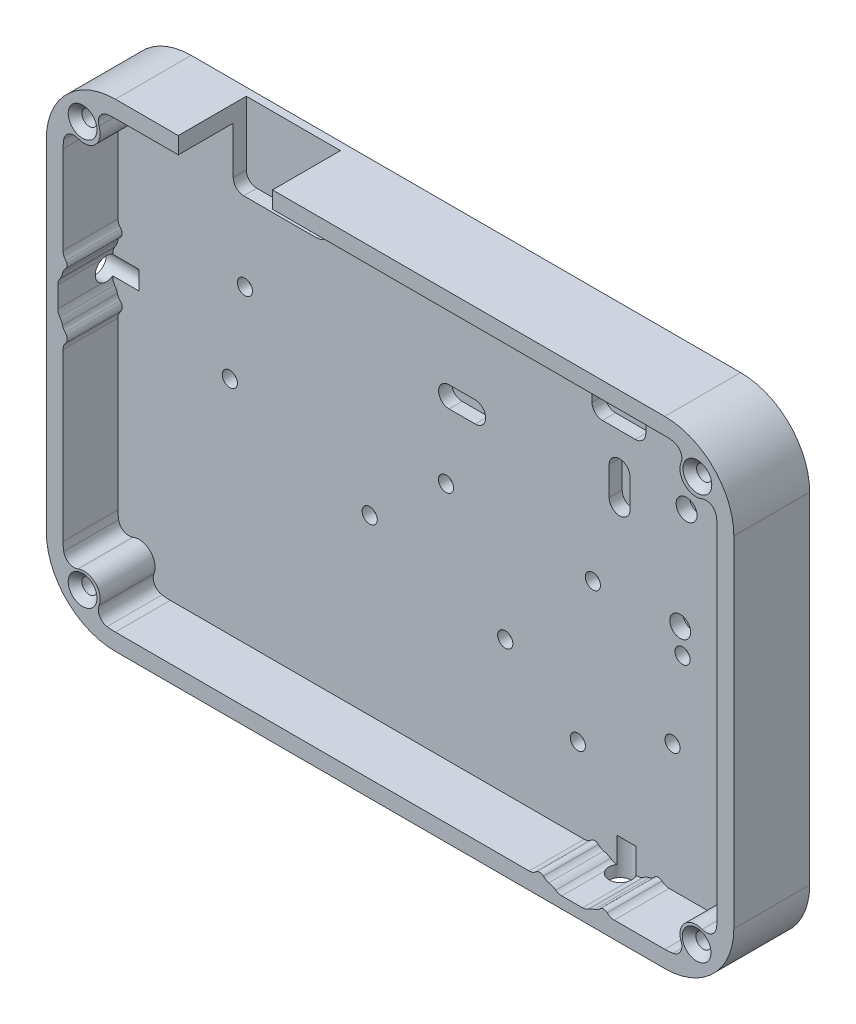
SolidWorks part; units mm, degrees
ref_plane "Спереди" through (0, 0, 0) normal (0, 0, 1) x (1, 0, 0)
ref_plane "Сверху" through (0, 0, 0) normal (0, 1, 0) x (1, 0, 0)
ref_plane "Справа" through (0, 0, 0) normal (1, 0, 0) x (0, 0, -1)
sketch "Elements" plane through (0, 0, 0) normal (0, 0, 1) x (1, 0, 0)
  line L0 (-0.35, 0) -> (0.35, 0)
  line L1 (0, -0.35) -> (0, 0.35)
  line L2 (104.65, 65) -> (105.35, 65)
  line L3 (105, 64.65) -> (105, 65.35)
  line L4 (104.65, 0) -> (105.35, 0)
  line L5 (105, -0.35) -> (105, 0.35)
  line L6 (-0.35, 65) -> (0.35, 65)
  line L7 (0, 64.65) -> (0, 65.35)
  line L8 (87.2, -10.5) -> (87.2, -9.5)
  line L9 (93.2, -10) -> (93.2, -4.2)
  line L10 (81.2, -4.2) -> (93.2, -4.2)
  line L11 (81.2, -10) -> (81.2, -4.2)
  line L12 (80.2, -10) -> (94.2, -10)
  line L13 (85.7, -15) -> (88.7, -14)
  line L14 (85.7, -15.5) -> (88.7, -14.5)
  line L15 (85.7, -16) -> (88.7, -15)
  line L16 (85.7, -16.5) -> (88.7, -15.5)
  line L17 (85.7, -17) -> (88.7, -16)
  line L18 (85.7, -17.5) -> (88.7, -16.5)
  line L19 (85.7, -18) -> (88.7, -17)
  line L20 (85.7, -18.5) -> (88.7, -17.5)
  line L21 (85.7, -19.5) -> (85.7, -11.5)
  line L22 (85.7, -19.5) -> (88.7, -19.5)
  line L23 (88.7, -19.5) -> (88.7, -11.5)
  line L24 (90.9, -10) -> (90.9, -5.25)
  line L25 (90.9, -5.25) -> (91.9, -5.25)
  line L26 (91.9, -10) -> (91.9, -5.25)
  line L27 (83.5, -10) -> (83.5, -5.25)
  line L28 (82.5, -5.25) -> (83.5, -5.25)
  line L29 (82.5, -10) -> (82.5, -5.25)
  line L30 (82.5, -10) -> (91.9, -10)
  line L31 (91.9, -11.5) -> (91.9, -10)
  line L32 (82.5, -11.5) -> (91.9, -11.5)
  line L33 (82.5, -11.5) -> (82.5, -10)
  line L34 (86.65, -5.225) -> (87.75, -5.225)
  line L35 (87.75, -10) -> (87.75, -5.225)
  line L36 (86.65, -10) -> (86.65, -5.225)
  line L37 (85.9, -9.7) -> (85.9, -4.8719) construction
  line L38 (94.225, 24.265) -> (94.225, 24.935)
  line L39 (93.89, 24.6) -> (94.56, 24.6)
  line L40 (92.855, 25.27) -> (95.595, 25.27)
  line L41 (92.855, 23.93) -> (92.855, 25.27)
  line L42 (92.855, 23.93) -> (95.595, 23.93)
  line L43 (95.595, 23.93) -> (95.595, 25.27)
  line L44 (93.425, 25) -> (95.025, 25)
  line L45 (93.425, 24.2) -> (93.425, 25)
  line L46 (93.425, 24.2) -> (95.025, 24.2)
  line L47 (95.025, 24.2) -> (95.025, 25)
  line L48 (96.325, 23.7) -> (93.8875, 23.7) construction
  line L49 (-10.5, 40) -> (-9.5, 40)
  line L50 (-10, 34) -> (-4.2, 34)
  line L51 (-4.2, 34) -> (-4.2, 46)
  line L52 (-10, 46) -> (-4.2, 46)
  line L53 (-10, 33) -> (-10, 47)
  line L54 (-15, 41.5) -> (-14, 38.5)
  line L55 (-15.5, 41.5) -> (-14.5, 38.5)
  line L56 (-16, 41.5) -> (-15, 38.5)
  line L57 (-16.5, 41.5) -> (-15.5, 38.5)
  line L58 (-17, 41.5) -> (-16, 38.5)
  line L59 (-17.5, 41.5) -> (-16.5, 38.5)
  line L60 (-18, 41.5) -> (-17, 38.5)
  line L61 (-18.5, 41.5) -> (-17.5, 38.5)
  line L62 (-19.5, 41.5) -> (-11.5, 41.5)
  line L63 (-19.5, 38.5) -> (-19.5, 41.5)
  line L64 (-19.5, 38.5) -> (-11.5, 38.5)
  line L65 (-10, 36.3) -> (-5.25, 36.3)
  line L66 (-5.25, 35.3) -> (-5.25, 36.3)
  line L67 (-10, 35.3) -> (-5.25, 35.3)
  line L68 (-10, 43.7) -> (-5.25, 43.7)
  line L69 (-5.25, 43.7) -> (-5.25, 44.7)
  line L70 (-10, 44.7) -> (-5.25, 44.7)
  line L71 (-10, 35.3) -> (-10, 44.7)
  line L72 (-11.5, 35.3) -> (-10, 35.3)
  line L73 (-11.5, 35.3) -> (-11.5, 44.7)
  line L74 (-11.5, 44.7) -> (-10, 44.7)
  line L75 (-5.225, 39.45) -> (-5.225, 40.55)
  line L76 (-10, 39.45) -> (-5.225, 39.45)
  line L77 (-10, 40.55) -> (-5.225, 40.55)
  line L78 (68.23, 59.48) -> (68.23, 64.98)
  line L79 (68.23, 64.98) -> (71.77, 64.98)
  line L80 (71.77, 59.48) -> (71.77, 64.98)
  line L81 (68.23, 59.48) -> (71.77, 59.48)
  line L82 (69.65, 63.5) -> (70.35, 63.5)
  line L83 (70, 63.15) -> (70, 63.85)
  line L84 (68.5, 59.73) -> (68.5, 63.73)
  line L85 (68.5, 63.73) -> (69.5, 64.73)
  line L86 (69.5, 64.73) -> (71.5, 64.73)
  line L87 (71.5, 59.73) -> (71.5, 64.73)
  line L88 (68.5, 59.73) -> (71.5, 59.73)
  line L89 (68.7, 61.9) -> (73.0594, 61.9) construction
  line L90 (21.025, 83.175) -> (21.025, 84.175)
  line L91 (13.025, 64.975) -> (13.025, 83.675)
  line L92 (13.025, 64.975) -> (29.025, 64.975)
  line L93 (29.025, 64.975) -> (29.025, 83.675)
  line L94 (13.025, 83.675) -> (29.025, 83.675)
  line L95 (21.025, 66.975) -> (21.025, 67.675)
  line L96 (20.675, 67.325) -> (21.375, 67.325)
  line L97 (13.3184, 75.025) -> (28.7953, 75.025)
  line L98 (15.025, 65.475) -> (24.525, 65.475)
  line L99 (24.525, 65.475) -> (27.025, 65.475)
  line L100 (13.275, 69.6999) -> (13.275, 75.025)
  line L101 (28.775, 69.6999) -> (28.775, 75.025)
  line L102 (88.2, 61.825) -> (94.8, 61.825)
  line L103 (88.2, 73.175) -> (94.8, 73.175)
  line L104 (88.2, 61.825) -> (88.2, 73.175)
  line L105 (94.8, 61.825) -> (94.8, 73.175)
  line L106 (91.5, 67) -> (91.5, 68)
  line L107 (91, 67.5) -> (92, 67.5)
  line L108 (88.45, 64.45) -> (94.55, 64.45)
  line L109 (88.45, 70.55) -> (94.55, 70.55)
  line L110 (88.45, 64.45) -> (88.45, 70.55)
  line L111 (94.55, 64.45) -> (94.55, 70.55)
  line L112 (81.4925, 46.5358) -> (83.2925, 46.5358)
  line L113 (81.4925, 45.6358) -> (81.4925, 46.5358)
  line L114 (81.4925, 45.6358) -> (83.2925, 45.6358)
  line L115 (83.2925, 45.6358) -> (83.2925, 46.5358)
  line L116 (82.3925, 45.8658) -> (82.3925, 46.3058)
  line L117 (82.1725, 46.0858) -> (82.6125, 46.0858)
  line L118 (81.8925, 46.3358) -> (82.8925, 46.3358)
  line L119 (81.8925, 45.8358) -> (81.8925, 46.3358)
  line L120 (81.8925, 45.8358) -> (82.8925, 45.8358)
  line L121 (82.8925, 45.8358) -> (82.8925, 46.3358)
  line L122 (81.9375, 48.9108) -> (81.9375, 45.0201) construction
  line L123 (94.385, 53.9133) -> (96.185, 53.9133)
  line L124 (96.185, 53.9133) -> (96.185, 54.8133)
  line L125 (94.385, 54.8133) -> (96.185, 54.8133)
  line L126 (94.385, 53.9133) -> (94.385, 54.8133)
  line L127 (95.285, 54.1433) -> (95.285, 54.5833)
  line L128 (95.065, 54.3633) -> (95.505, 54.3633)
  line L129 (94.785, 54.1133) -> (95.785, 54.1133)
  line L130 (95.785, 54.1133) -> (95.785, 54.6133)
  line L131 (94.785, 54.6133) -> (95.785, 54.6133)
  line L132 (94.785, 54.1133) -> (94.785, 54.6133)
  line L133 (96.225, 55.9883) -> (92.3344, 55.9883) construction
  line L134 (87.05, 43.3556) -> (88.85, 43.3556)
  line L135 (88.85, 43.3556) -> (88.85, 44.2556)
  line L136 (87.05, 44.2556) -> (88.85, 44.2556)
  line L137 (87.05, 43.3556) -> (87.05, 44.2556)
  line L138 (87.95, 43.5856) -> (87.95, 44.0256)
  line L139 (87.73, 43.8056) -> (88.17, 43.8056)
  line L140 (87.45, 43.5556) -> (88.45, 43.5556)
  line L141 (88.45, 43.5556) -> (88.45, 44.0556)
  line L142 (87.45, 44.0556) -> (88.45, 44.0556)
  line L143 (87.45, 43.5556) -> (87.45, 44.0556)
  line L144 (91.56, 44.2306) -> (88.1381, 44.2306) construction
  line L145 (88.86, 41.3656) -> (88.86, 43.1656)
  line L146 (87.96, 43.1656) -> (88.86, 43.1656)
  line L147 (87.96, 41.3656) -> (87.96, 43.1656)
  line L148 (87.96, 41.3656) -> (88.86, 41.3656)
  line L149 (88.19, 42.2656) -> (88.63, 42.2656)
  line L150 (88.41, 42.0456) -> (88.41, 42.4856)
  line L151 (88.66, 41.7656) -> (88.66, 42.7656)
  line L152 (88.16, 42.7656) -> (88.66, 42.7656)
  line L153 (88.16, 41.7656) -> (88.16, 42.7656)
  line L154 (88.16, 41.7656) -> (88.66, 41.7656)
  line L155 (91.66, 42.4806) -> (88.0038, 42.4806) construction
  line L156 (91.8202, 42.4931) -> (91.8202, 44.2931)
  line L157 (90.9202, 44.2931) -> (91.8202, 44.2931)
  line L158 (90.9202, 42.4931) -> (90.9202, 44.2931)
  line L159 (90.9202, 42.4931) -> (91.8202, 42.4931)
  line L160 (91.1502, 43.3931) -> (91.5902, 43.3931)
  line L161 (91.3702, 43.1731) -> (91.3702, 43.6131)
  line L162 (91.6202, 42.8931) -> (91.6202, 43.8931)
  line L163 (91.1202, 43.8931) -> (91.6202, 43.8931)
  line L164 (91.1202, 42.8931) -> (91.1202, 43.8931)
  line L165 (91.1202, 42.8931) -> (91.6202, 42.8931)
  line L166 (92.0702, 43.0331) -> (94.9764, 43.0331) construction
  line L167 (92.2249, 34.0083) -> (92.2249, 35.8083)
  line L168 (92.2249, 34.0083) -> (93.1249, 34.0083)
  line L169 (93.1249, 34.0083) -> (93.1249, 35.8083)
  line L170 (92.2249, 35.8083) -> (93.1249, 35.8083)
  line L171 (92.4549, 34.9083) -> (92.8949, 34.9083)
  line L172 (92.6749, 34.6883) -> (92.6749, 35.1283)
  line L173 (92.4249, 34.4083) -> (92.4249, 35.4083)
  line L174 (92.4249, 34.4083) -> (92.9249, 34.4083)
  line L175 (92.9249, 34.4083) -> (92.9249, 35.4083)
  line L176 (92.4249, 35.4083) -> (92.9249, 35.4083)
  line L177 (92.1999, 37.5983) -> (92.1999, 34.692) construction
  line L178 (93.4399, 34.8733) -> (95.2399, 34.8733)
  line L179 (93.4399, 33.9733) -> (93.4399, 34.8733)
  line L180 (93.4399, 33.9733) -> (95.2399, 33.9733)
  line L181 (95.2399, 33.9733) -> (95.2399, 34.8733)
  line L182 (94.3399, 34.2033) -> (94.3399, 34.6433)
  line L183 (94.1199, 34.4233) -> (94.5599, 34.4233)
  line L184 (93.8399, 34.6733) -> (94.8399, 34.6733)
  line L185 (93.8399, 34.1733) -> (93.8399, 34.6733)
  line L186 (93.8399, 34.1733) -> (94.8399, 34.1733)
  line L187 (94.8399, 34.1733) -> (94.8399, 34.6733)
  line L188 (93.5249, 37.5233) -> (93.5249, 34.617) construction
  line L189 (95.4249, 33.9833) -> (95.4249, 35.7833)
  line L190 (95.4249, 33.9833) -> (96.3249, 33.9833)
  line L191 (96.3249, 33.9833) -> (96.3249, 35.7833)
  line L192 (95.4249, 35.7833) -> (96.3249, 35.7833)
  line L193 (95.6549, 34.8833) -> (96.0949, 34.8833)
  line L194 (95.8749, 34.6633) -> (95.8749, 35.1033)
  line L195 (95.6249, 34.3833) -> (95.6249, 35.3833)
  line L196 (95.6249, 34.3833) -> (96.1249, 34.3833)
  line L197 (96.1249, 34.3833) -> (96.1249, 35.3833)
  line L198 (95.6249, 35.3833) -> (96.1249, 35.3833)
  line L199 (95.3999, 37.5483) -> (95.3999, 34.642) construction
  line L200 (70.115, 36.6733) -> (71.915, 36.6733)
  line L201 (70.115, 35.7733) -> (70.115, 36.6733)
  line L202 (70.115, 35.7733) -> (71.915, 35.7733)
  line L203 (71.915, 35.7733) -> (71.915, 36.6733)
  line L204 (71.015, 36.0033) -> (71.015, 36.4433)
  line L205 (70.795, 36.2233) -> (71.235, 36.2233)
  line L206 (70.515, 36.4733) -> (71.515, 36.4733)
  line L207 (70.515, 35.9733) -> (70.515, 36.4733)
  line L208 (70.515, 35.9733) -> (71.515, 35.9733)
  line L209 (71.515, 35.9733) -> (71.515, 36.4733)
  line L210 (69.675, 35.5233) -> (69.675, 38.4295) construction
  line L211 (70.83, 39.9883) -> (72.17, 39.9883)
  line L212 (72.17, 37.2483) -> (72.17, 39.9883)
  line L213 (70.83, 37.2483) -> (72.17, 37.2483)
  line L214 (70.83, 37.2483) -> (70.83, 39.9883)
  line L215 (71.5, 38.2833) -> (71.5, 38.9533)
  line L216 (71.165, 38.6183) -> (71.835, 38.6183)
  line L217 (71.1, 39.4183) -> (71.9, 39.4183)
  line L218 (71.9, 37.8183) -> (71.9, 39.4183)
  line L219 (71.1, 37.8183) -> (71.9, 37.8183)
  line L220 (71.1, 37.8183) -> (71.1, 39.4183)
  line L221 (70.7, 38.0233) -> (70.7, 40.9295) construction
  line L222 (5.95, 51.9233) -> (7.75, 51.9233)
  line L223 (5.95, 51.0233) -> (5.95, 51.9233)
  line L224 (5.95, 51.0233) -> (7.75, 51.0233)
  line L225 (7.75, 51.0233) -> (7.75, 51.9233)
  line L226 (6.85, 51.2533) -> (6.85, 51.6933)
  line L227 (6.63, 51.4733) -> (7.07, 51.4733)
  line L228 (6.35, 51.7233) -> (7.35, 51.7233)
  line L229 (6.35, 51.2233) -> (6.35, 51.7233)
  line L230 (6.35, 51.2233) -> (7.35, 51.2233)
  line L231 (7.35, 51.2233) -> (7.35, 51.7233)
  line L232 (8.65, 51.0483) -> (11.5563, 51.0483) construction
  line L233 (6.83, 55.4383) -> (8.17, 55.4383)
  line L234 (8.17, 52.6983) -> (8.17, 55.4383)
  line L235 (6.83, 52.6983) -> (8.17, 52.6983)
  line L236 (6.83, 52.6983) -> (6.83, 55.4383)
  line L237 (7.5, 53.7333) -> (7.5, 54.4033)
  line L238 (7.165, 54.0683) -> (7.835, 54.0683)
  line L239 (7.1, 54.8683) -> (7.9, 54.8683)
  line L240 (7.9, 53.2683) -> (7.9, 54.8683)
  line L241 (7.1, 53.2683) -> (7.9, 53.2683)
  line L242 (7.1, 53.2683) -> (7.1, 54.8683)
  line L243 (7.225, 56.1233) -> (10.1313, 56.1233) construction
  line L244 (87.27, 51.6483) -> (88.27, 51.6483)
  line L245 (87.77, 51.1483) -> (87.77, 52.1483)
  line L246 (85.02, 47.9733) -> (85.02, 55.3233)
  line L247 (90.52, 47.9733) -> (90.52, 55.3233)
  line L248 (85.02, 47.9733) -> (90.52, 47.9733)
  line L249 (85.02, 55.3233) -> (90.52, 55.3233)
  line L250 (85.27, 49.6483) -> (85.27, 53.6483)
  line L251 (90.27, 49.6483) -> (90.27, 53.6483)
  line L252 (85.27, 49.6483) -> (90.27, 49.6483)
  line L253 (85.27, 53.6483) -> (90.27, 53.6483)
  line L254 (87.7249, 35.3733) -> (88.7249, 35.3733)
  line L255 (88.2249, 34.8733) -> (88.2249, 35.8733)
  line L256 (86.9249, 33.9233) -> (86.9249, 36.8233)
  line L257 (86.9249, 33.9233) -> (89.5249, 33.9233)
  line L258 (86.9249, 36.8233) -> (89.5249, 36.8233)
  line L259 (89.5249, 33.9233) -> (89.5249, 36.8233)
  line L260 (87.1749, 34.3233) -> (87.1749, 36.4233)
  line L261 (89.2749, 34.3233) -> (89.2749, 36.4233)
  line L262 (87.1749, 34.3233) -> (89.2749, 34.3233)
  line L263 (87.1749, 36.4233) -> (89.2749, 36.4233)
  line L264 (88.9999, 35.7316) -> (84.6405, 35.7316) construction
  line L265 (70.5, 23.8483) -> (71.5, 23.8483)
  line L266 (71, 23.3483) -> (71, 24.3483)
  line L267 (68.65, 21.9983) -> (68.65, 25.6983)
  line L268 (73.35, 21.9983) -> (73.35, 25.6983)
  line L269 (68.65, 21.9983) -> (73.35, 21.9983)
  line L270 (68.65, 25.6983) -> (73.35, 25.6983)
  line L271 (69.2, 22.5483) -> (69.2, 25.1483)
  line L272 (72.8, 22.5483) -> (72.8, 25.1483)
  line L273 (69.2, 22.5483) -> (72.8, 22.5483)
  line L274 (69.2, 25.1483) -> (72.8, 25.1483)
  line L275 (74.2149, 21.7691) -> (69.8555, 21.7691) construction
  line L276 (6.4, 39.9483) -> (7.4, 39.9483)
  line L277 (6.9, 39.4483) -> (6.9, 40.4483)
  line L278 (4.55, 38.0983) -> (4.55, 41.7983)
  line L279 (9.25, 38.0983) -> (9.25, 41.7983)
  line L280 (4.55, 38.0983) -> (9.25, 38.0983)
  line L281 (4.55, 41.7983) -> (9.25, 41.7983)
  line L282 (5.1, 38.6483) -> (5.1, 41.2483)
  line L283 (8.7, 38.6483) -> (8.7, 41.2483)
  line L284 (5.1, 38.6483) -> (8.7, 38.6483)
  line L285 (5.1, 41.2483) -> (8.7, 41.2483)
  line L286 (10.1149, 37.8858) -> (5.7555, 37.8858) construction
  line L287 (53.425, 58.2233) -> (54.125, 58.2233)
  line L288 (53.775, 57.8733) -> (53.775, 58.5733)
  line L289 (51.075, 54.5633) -> (56.475, 54.5633)
  line L290 (56.475, 54.5633) -> (56.475, 61.8833)
  line L291 (51.075, 61.8833) -> (56.475, 61.8833)
  line L292 (51.075, 54.5633) -> (51.075, 61.8833)
  line L293 (51.325, 56.2733) -> (56.225, 56.2733)
  line L294 (56.225, 56.2733) -> (56.225, 60.1733)
  line L295 (51.325, 60.1733) -> (56.225, 60.1733)
  line L296 (51.325, 56.2733) -> (51.325, 60.1733)
  line L297 (51.5221, 57.9278) -> (55.0096, 57.9278) construction
  line L298 (35.4, 58.2233) -> (36.1, 58.2233)
  line L299 (35.75, 57.8733) -> (35.75, 58.5733)
  line L300 (33.05, 54.5633) -> (38.45, 54.5633)
  line L301 (38.45, 54.5633) -> (38.45, 61.8833)
  line L302 (33.05, 61.8833) -> (38.45, 61.8833)
  line L303 (33.05, 54.5633) -> (33.05, 61.8833)
  line L304 (33.3, 56.2733) -> (38.2, 56.2733)
  line L305 (38.2, 56.2733) -> (38.2, 60.1733)
  line L306 (33.3, 60.1733) -> (38.2, 60.1733)
  line L307 (33.3, 56.2733) -> (33.3, 60.1733)
  line L308 (33.4971, 57.9278) -> (36.9846, 57.9278) construction
  line L309 (44.9, 58.2233) -> (45.6, 58.2233)
  line L310 (45.25, 57.8733) -> (45.25, 58.5733)
  line L311 (42.55, 54.5633) -> (47.95, 54.5633)
  line L312 (47.95, 54.5633) -> (47.95, 61.8833)
  line L313 (42.55, 61.8833) -> (47.95, 61.8833)
  line L314 (42.55, 54.5633) -> (42.55, 61.8833)
  line L315 (42.8, 56.2733) -> (47.7, 56.2733)
  line L316 (47.7, 56.2733) -> (47.7, 60.1733)
  line L317 (42.8, 60.1733) -> (47.7, 60.1733)
  line L318 (42.8, 56.2733) -> (42.8, 60.1733)
  line L319 (42.9971, 57.9278) -> (46.1096, 57.9278) construction
  line L320 (80.6925, 45.6008) -> (81.1325, 45.6008)
  line L321 (80.9125, 45.3808) -> (80.9125, 45.8208)
  line L322 (81.3525, 44.7008) -> (81.3525, 46.5008)
  line L323 (80.4725, 46.5008) -> (81.3525, 46.5008)
  line L324 (80.4725, 44.7008) -> (80.4725, 46.5008)
  line L325 (80.4725, 44.7008) -> (81.3525, 44.7008)
  line L326 (81.1625, 45.1008) -> (81.1625, 46.1008)
  line L327 (80.6625, 46.1008) -> (81.1625, 46.1008)
  line L328 (80.6625, 45.1008) -> (80.6625, 46.1008)
  line L329 (80.6625, 45.1008) -> (81.1625, 45.1008)
  line L330 (81.4375, 42.0608) -> (81.4375, 46.1858) construction
  line L331 (83.6675, 45.5758) -> (84.1075, 45.5758)
  line L332 (83.8875, 45.3558) -> (83.8875, 45.7958)
  line L333 (84.3275, 44.6758) -> (84.3275, 46.4758)
  line L334 (83.4475, 46.4758) -> (84.3275, 46.4758)
  line L335 (83.4475, 44.6758) -> (83.4475, 46.4758)
  line L336 (83.4475, 44.6758) -> (84.3275, 44.6758)
  line L337 (84.1375, 45.0758) -> (84.1375, 46.0758)
  line L338 (83.6375, 46.0758) -> (84.1375, 46.0758)
  line L339 (83.6375, 45.0758) -> (83.6375, 46.0758)
  line L340 (83.6375, 45.0758) -> (84.1375, 45.0758)
  line L341 (84.2375, 42.0608) -> (84.2375, 46.4201) construction
  line L342 (93.58, 53.8883) -> (94.02, 53.8883)
  line L343 (93.8, 53.6683) -> (93.8, 54.1083)
  line L344 (94.24, 52.9883) -> (94.24, 54.7883)
  line L345 (93.36, 54.7883) -> (94.24, 54.7883)
  line L346 (93.36, 52.9883) -> (93.36, 54.7883)
  line L347 (93.36, 52.9883) -> (94.24, 52.9883)
  line L348 (94.05, 53.3883) -> (94.05, 54.3883)
  line L349 (93.55, 54.3883) -> (94.05, 54.3883)
  line L350 (93.55, 53.3883) -> (93.55, 54.3883)
  line L351 (93.55, 53.3883) -> (94.05, 53.3883)
  line L352 (93.125, 55.6133) -> (88.7656, 55.6133) construction
  line L353 (96.78, 53.8883) -> (97.22, 53.8883)
  line L354 (97, 53.6683) -> (97, 54.1083)
  line L355 (97.44, 52.9883) -> (97.44, 54.7883)
  line L356 (96.56, 54.7883) -> (97.44, 54.7883)
  line L357 (96.56, 52.9883) -> (96.56, 54.7883)
  line L358 (96.56, 52.9883) -> (97.44, 52.9883)
  line L359 (97.25, 53.3883) -> (97.25, 54.3883)
  line L360 (96.75, 54.3883) -> (97.25, 54.3883)
  line L361 (96.75, 53.3883) -> (96.75, 54.3883)
  line L362 (96.75, 53.3883) -> (97.25, 53.3883)
  line L363 (99.725, 56.0633) -> (95.3656, 56.0633) construction
  line L364 (87.92, 44.7356) -> (87.92, 45.1756)
  line L365 (87.7, 44.9556) -> (88.14, 44.9556)
  line L366 (87.02, 44.5156) -> (88.82, 44.5156)
  line L367 (88.82, 44.5156) -> (88.82, 45.3956)
  line L368 (87.02, 45.3956) -> (88.82, 45.3956)
  line L369 (87.02, 44.5156) -> (87.02, 45.3956)
  line L370 (87.42, 44.7056) -> (88.42, 44.7056)
  line L371 (88.42, 44.7056) -> (88.42, 45.2056)
  line L372 (87.42, 45.2056) -> (88.42, 45.2056)
  line L373 (87.42, 44.7056) -> (87.42, 45.2056)
  line L374 (91.735, 45.3556) -> (87.3756, 45.3556) construction
  line L375 (90.8852, 44.6731) -> (90.8852, 45.1131)
  line L376 (90.6652, 44.8931) -> (91.1052, 44.8931)
  line L377 (89.9852, 44.4531) -> (91.7852, 44.4531)
  line L378 (91.7852, 44.4531) -> (91.7852, 45.3331)
  line L379 (89.9852, 45.3331) -> (91.7852, 45.3331)
  line L380 (89.9852, 44.4531) -> (89.9852, 45.3331)
  line L381 (90.3852, 44.6431) -> (91.3852, 44.6431)
  line L382 (91.3852, 44.6431) -> (91.3852, 45.1431)
  line L383 (90.3852, 45.1431) -> (91.3852, 45.1431)
  line L384 (90.3852, 44.6431) -> (90.3852, 45.1431)
  line L385 (92.0452, 44.5931) -> (96.4045, 44.5931) construction
  line L386 (87.95, 40.5106) -> (87.95, 40.9506)
  line L387 (87.73, 40.7306) -> (88.17, 40.7306)
  line L388 (87.05, 40.2906) -> (88.85, 40.2906)
  line L389 (88.85, 40.2906) -> (88.85, 41.1706)
  line L390 (87.05, 41.1706) -> (88.85, 41.1706)
  line L391 (87.05, 40.2906) -> (87.05, 41.1706)
  line L392 (87.45, 40.4806) -> (88.45, 40.4806)
  line L393 (88.45, 40.4806) -> (88.45, 40.9806)
  line L394 (87.45, 40.9806) -> (88.45, 40.9806)
  line L395 (87.45, 40.4806) -> (87.45, 40.9806)
  line L396 (91.61, 41.1556) -> (87.2506, 41.1556) construction
  line L397 (91.8802, 41.5731) -> (91.8802, 42.0131)
  line L398 (91.6602, 41.7931) -> (92.1002, 41.7931)
  line L399 (90.9802, 42.2331) -> (92.7802, 42.2331)
  line L400 (90.9802, 41.3531) -> (90.9802, 42.2331)
  line L401 (90.9802, 41.3531) -> (92.7802, 41.3531)
  line L402 (92.7802, 41.3531) -> (92.7802, 42.2331)
  line L403 (91.3802, 42.0431) -> (92.3802, 42.0431)
  line L404 (91.3802, 41.5431) -> (91.3802, 42.0431)
  line L405 (91.3802, 41.5431) -> (92.3802, 41.5431)
  line L406 (92.3802, 41.5431) -> (92.3802, 42.0431)
  line L407 (90.6952, 42.2431) -> (86.3358, 42.2431) construction
  line L408 (91.0549, 34.9333) -> (91.4949, 34.9333)
  line L409 (91.2749, 34.7133) -> (91.2749, 35.1533)
  line L410 (90.8349, 34.0333) -> (90.8349, 35.8333)
  line L411 (90.8349, 34.0333) -> (91.7149, 34.0333)
  line L412 (91.7149, 34.0333) -> (91.7149, 35.8333)
  line L413 (90.8349, 35.8333) -> (91.7149, 35.8333)
  line L414 (91.0249, 34.4333) -> (91.0249, 35.4333)
  line L415 (91.0249, 34.4333) -> (91.5249, 34.4333)
  line L416 (91.5249, 34.4333) -> (91.5249, 35.4333)
  line L417 (91.0249, 35.4333) -> (91.5249, 35.4333)
  line L418 (90.7499, 38.3733) -> (90.7499, 34.0139) construction
  line L419 (70.98, 32.4833) -> (70.98, 34.2633)
  line L420 (67.84, 32.4833) -> (70.98, 32.4833)
  line L421 (67.84, 32.4833) -> (67.84, 34.2633)
  line L422 (67.84, 34.2633) -> (70.98, 34.2633)
  line L423 (69.06, 33.3733) -> (69.76, 33.3733)
  line L424 (69.41, 33.0233) -> (69.41, 33.7233)
  line L425 (70.46, 32.6933) -> (70.46, 34.0533)
  line L426 (68.36, 32.6933) -> (70.46, 32.6933)
  line L427 (68.36, 32.6933) -> (68.36, 34.0533)
  line L428 (68.36, 34.0533) -> (70.46, 34.0533)
  line L429 (68.45, 31.3233) -> (72.3406, 31.3233) construction
  line L430 (68.225, 29.7983) -> (70.975, 29.7983)
  line L431 (68.225, 29.7983) -> (68.225, 31.1483)
  line L432 (69.265, 30.4733) -> (69.935, 30.4733)
  line L433 (69.6, 30.1383) -> (69.6, 30.8083)
  line L434 (68.225, 31.1483) -> (70.975, 31.1483)
  line L435 (70.975, 29.7983) -> (70.975, 31.1483)
  line L436 (70.4, 30.0733) -> (70.4, 30.8733)
  line L437 (68.8, 30.0733) -> (70.4, 30.0733)
  line L438 (68.8, 30.0733) -> (68.8, 30.8733)
  line L439 (68.8, 30.8733) -> (70.4, 30.8733)
  line L440 (68.3, 28.7233) -> (72.425, 28.7233) construction
  line L441 (70.0063, 27.9033) -> (70.0063, 28.3433)
  line L442 (69.7863, 28.1233) -> (70.2263, 28.1233)
  line L443 (69.1063, 28.5633) -> (70.9063, 28.5633)
  line L444 (69.1063, 27.6833) -> (69.1063, 28.5633)
  line L445 (69.1063, 27.6833) -> (70.9063, 27.6833)
  line L446 (70.9063, 27.6833) -> (70.9063, 28.5633)
  line L447 (69.5063, 28.3733) -> (70.5063, 28.3733)
  line L448 (69.5063, 27.8733) -> (69.5063, 28.3733)
  line L449 (69.5063, 27.8733) -> (70.5063, 27.8733)
  line L450 (70.5063, 27.8733) -> (70.5063, 28.3733)
  line L451 (68.3063, 26.5733) -> (72.1969, 26.5733) construction
  line L452 (74.16, 32.4833) -> (74.16, 34.2633)
  line L453 (71.02, 32.4833) -> (74.16, 32.4833)
  line L454 (71.02, 32.4833) -> (71.02, 34.2633)
  line L455 (71.02, 34.2633) -> (74.16, 34.2633)
  line L456 (72.24, 33.3733) -> (72.94, 33.3733)
  line L457 (72.59, 33.0233) -> (72.59, 33.7233)
  line L458 (73.64, 32.6933) -> (73.64, 34.0533)
  line L459 (71.54, 32.6933) -> (73.64, 32.6933)
  line L460 (71.54, 32.6933) -> (71.54, 34.0533)
  line L461 (71.54, 34.0533) -> (73.64, 34.0533)
  line L462 (71.7, 31.3483) -> (75.5906, 31.3483) construction
  line L463 (71.025, 29.7983) -> (73.775, 29.7983)
  line L464 (71.025, 29.7983) -> (71.025, 31.1483)
  line L465 (72.065, 30.4733) -> (72.735, 30.4733)
  line L466 (72.4, 30.1383) -> (72.4, 30.8083)
  line L467 (71.025, 31.1483) -> (73.775, 31.1483)
  line L468 (73.775, 29.7983) -> (73.775, 31.1483)
  line L469 (73.2, 30.0733) -> (73.2, 30.8733)
  line L470 (71.6, 30.0733) -> (73.2, 30.0733)
  line L471 (71.6, 30.0733) -> (71.6, 30.8733)
  line L472 (71.6, 30.8733) -> (73.2, 30.8733)
  line L473 (71.55, 28.7983) -> (75.4406, 28.7983) construction
  line L474 (71.9938, 27.9033) -> (71.9938, 28.3433)
  line L475 (71.7738, 28.1233) -> (72.2138, 28.1233)
  line L476 (71.0938, 28.5633) -> (72.8938, 28.5633)
  line L477 (71.0938, 27.6833) -> (71.0938, 28.5633)
  line L478 (71.0938, 27.6833) -> (72.8938, 27.6833)
  line L479 (72.8938, 27.6833) -> (72.8938, 28.5633)
  line L480 (71.4938, 28.3733) -> (72.4938, 28.3733)
  line L481 (71.4938, 27.8733) -> (71.4938, 28.3733)
  line L482 (71.4938, 27.8733) -> (72.4938, 27.8733)
  line L483 (72.4938, 27.8733) -> (72.4938, 28.3733)
  line L484 (71.6188, 26.5733) -> (75.5094, 26.5733) construction
  line L485 (6.805, 48.0833) -> (6.805, 49.8633)
  line L486 (3.665, 48.0833) -> (6.805, 48.0833)
  line L487 (3.665, 48.0833) -> (3.665, 49.8633)
  line L488 (3.665, 49.8633) -> (6.805, 49.8633)
  line L489 (4.885, 48.9733) -> (5.585, 48.9733)
  line L490 (5.235, 48.6233) -> (5.235, 49.3233)
  line L491 (6.285, 48.2933) -> (6.285, 49.6533)
  line L492 (4.185, 48.2933) -> (6.285, 48.2933)
  line L493 (4.185, 48.2933) -> (4.185, 49.6533)
  line L494 (4.185, 49.6533) -> (6.285, 49.6533)
  line L495 (4.1, 46.9983) -> (7.9906, 46.9983) construction
  line L496 (4.07, 45.2983) -> (6.82, 45.2983)
  line L497 (4.07, 45.2983) -> (4.07, 46.6483)
  line L498 (5.11, 45.9733) -> (5.78, 45.9733)
  line L499 (5.445, 45.6383) -> (5.445, 46.3083)
  line L500 (4.07, 46.6483) -> (6.82, 46.6483)
  line L501 (6.82, 45.2983) -> (6.82, 46.6483)
  line L502 (6.245, 45.5733) -> (6.245, 46.3733)
  line L503 (4.645, 45.5733) -> (6.245, 45.5733)
  line L504 (4.645, 45.5733) -> (4.645, 46.3733)
  line L505 (4.645, 46.3733) -> (6.245, 46.3733)
  line L506 (4.425, 44.2483) -> (8.3156, 44.2483) construction
  line L507 (5.89, 43.2533) -> (5.89, 43.6933)
  line L508 (5.67, 43.4733) -> (6.11, 43.4733)
  line L509 (4.99, 43.9133) -> (6.79, 43.9133)
  line L510 (4.99, 43.0333) -> (4.99, 43.9133)
  line L511 (4.99, 43.0333) -> (6.79, 43.0333)
  line L512 (6.79, 43.0333) -> (6.79, 43.9133)
  line L513 (5.39, 43.7233) -> (6.39, 43.7233)
  line L514 (5.39, 43.2233) -> (5.39, 43.7233)
  line L515 (5.39, 43.2233) -> (6.39, 43.2233)
  line L516 (6.39, 43.2233) -> (6.39, 43.7233)
  line L517 (3.875, 41.9733) -> (7.7656, 41.9733) construction
  line L518 (9.985, 48.0833) -> (9.985, 49.8633)
  line L519 (6.845, 48.0833) -> (9.985, 48.0833)
  line L520 (6.845, 48.0833) -> (6.845, 49.8633)
  line L521 (6.845, 49.8633) -> (9.985, 49.8633)
  line L522 (8.065, 48.9733) -> (8.765, 48.9733)
  line L523 (8.415, 48.6233) -> (8.415, 49.3233)
  line L524 (9.465, 48.2933) -> (9.465, 49.6533)
  line L525 (7.365, 48.2933) -> (9.465, 48.2933)
  line L526 (7.365, 48.2933) -> (7.365, 49.6533)
  line L527 (7.365, 49.6533) -> (9.465, 49.6533)
  line L528 (7.7, 47.0483) -> (11.5906, 47.0483) construction
  line L529 (6.855, 45.2983) -> (9.605, 45.2983)
  line L530 (6.855, 45.2983) -> (6.855, 46.6483)
  line L531 (7.895, 45.9733) -> (8.565, 45.9733)
  line L532 (8.23, 45.6383) -> (8.23, 46.3083)
  line L533 (6.855, 46.6483) -> (9.605, 46.6483)
  line L534 (9.605, 45.2983) -> (9.605, 46.6483)
  line L535 (9.03, 45.5733) -> (9.03, 46.3733)
  line L536 (7.43, 45.5733) -> (9.03, 45.5733)
  line L537 (7.43, 45.5733) -> (7.43, 46.3733)
  line L538 (7.43, 46.3733) -> (9.03, 46.3733)
  line L539 (7.675, 44.2483) -> (11.0969, 44.2483) construction
  line L540 (7.885, 43.2533) -> (7.885, 43.6933)
  line L541 (7.665, 43.4733) -> (8.105, 43.4733)
  line L542 (6.985, 43.9133) -> (8.785, 43.9133)
  line L543 (6.985, 43.0333) -> (6.985, 43.9133)
  line L544 (6.985, 43.0333) -> (8.785, 43.0333)
  line L545 (8.785, 43.0333) -> (8.785, 43.9133)
  line L546 (7.385, 43.7233) -> (8.385, 43.7233)
  line L547 (7.385, 43.2233) -> (7.385, 43.7233)
  line L548 (7.385, 43.2233) -> (8.385, 43.2233)
  line L549 (8.385, 43.2233) -> (8.385, 43.7233)
  line L550 (7.65, 41.9983) -> (11.3063, 41.9983) construction
  line L551 (52.05, 51.0233) -> (54.8, 51.0233)
  line L552 (54.8, 49.6733) -> (54.8, 51.0233)
  line L553 (53.09, 50.3483) -> (53.76, 50.3483)
  line L554 (53.425, 50.0133) -> (53.425, 50.6833)
  line L555 (52.05, 49.6733) -> (54.8, 49.6733)
  line L556 (52.05, 49.6733) -> (52.05, 51.0233)
  line L557 (52.625, 49.9483) -> (52.625, 50.7483)
  line L558 (52.625, 50.7483) -> (54.225, 50.7483)
  line L559 (54.225, 49.9483) -> (54.225, 50.7483)
  line L560 (52.625, 49.9483) -> (54.225, 49.9483)
  line L561 (50.625, 51.2483) -> (53.5313, 51.2483) construction
  line L562 (34.0105, 49.9483) -> (36.7605, 49.9483)
  line L563 (36.7605, 48.5983) -> (36.7605, 49.9483)
  line L564 (35.0505, 49.2733) -> (35.7205, 49.2733)
  line L565 (35.3855, 48.9383) -> (35.3855, 49.6083)
  line L566 (34.0105, 48.5983) -> (36.7605, 48.5983)
  line L567 (34.0105, 48.5983) -> (34.0105, 49.9483)
  line L568 (34.5855, 48.8733) -> (34.5855, 49.6733)
  line L569 (34.5855, 49.6733) -> (36.1855, 49.6733)
  line L570 (36.1855, 48.8733) -> (36.1855, 49.6733)
  line L571 (34.5855, 48.8733) -> (36.1855, 48.8733)
  line L572 (32.5855, 50.1733) -> (35.4918, 50.1733) construction
  line L573 (43.5, 49.9233) -> (46.25, 49.9233)
  line L574 (46.25, 48.5733) -> (46.25, 49.9233)
  line L575 (44.54, 49.2483) -> (45.21, 49.2483)
  line L576 (44.875, 48.9133) -> (44.875, 49.5833)
  line L577 (43.5, 48.5733) -> (46.25, 48.5733)
  line L578 (43.5, 48.5733) -> (43.5, 49.9233)
  line L579 (44.075, 48.8483) -> (44.075, 49.6483)
  line L580 (44.075, 49.6483) -> (45.675, 49.6483)
  line L581 (45.675, 48.8483) -> (45.675, 49.6483)
  line L582 (44.075, 48.8483) -> (45.675, 48.8483)
  line L583 (42.075, 50.1483) -> (44.9813, 50.1483) construction
  line L584 (53.55, 52.8483) -> (56.3, 52.8483)
  line L585 (56.3, 51.4983) -> (56.3, 52.8483)
  line L586 (54.59, 52.1733) -> (55.26, 52.1733)
  line L587 (54.925, 51.8383) -> (54.925, 52.5083)
  line L588 (53.55, 51.4983) -> (56.3, 51.4983)
  line L589 (53.55, 51.4983) -> (53.55, 52.8483)
  line L590 (54.125, 51.7733) -> (54.125, 52.5733)
  line L591 (54.125, 52.5733) -> (55.725, 52.5733)
  line L592 (55.725, 51.7733) -> (55.725, 52.5733)
  line L593 (54.125, 51.7733) -> (55.725, 51.7733)
  line L594 (52.125, 53.0733) -> (55.0313, 53.0733) construction
  line L595 (35.525, 52.8483) -> (38.275, 52.8483)
  line L596 (38.275, 51.4983) -> (38.275, 52.8483)
  line L597 (36.565, 52.1733) -> (37.235, 52.1733)
  line L598 (36.9, 51.8383) -> (36.9, 52.5083)
  line L599 (35.525, 51.4983) -> (38.275, 51.4983)
  line L600 (35.525, 51.4983) -> (35.525, 52.8483)
  line L601 (36.1, 51.7733) -> (36.1, 52.5733)
  line L602 (36.1, 52.5733) -> (37.7, 52.5733)
  line L603 (37.7, 51.7733) -> (37.7, 52.5733)
  line L604 (36.1, 51.7733) -> (37.7, 51.7733)
  line L605 (34.1, 53.0733) -> (37.0063, 53.0733) construction
  line L606 (45.025, 52.8483) -> (47.775, 52.8483)
  line L607 (47.775, 51.4983) -> (47.775, 52.8483)
  line L608 (46.065, 52.1733) -> (46.735, 52.1733)
  line L609 (46.4, 51.8383) -> (46.4, 52.5083)
  line L610 (45.025, 51.4983) -> (47.775, 51.4983)
  line L611 (45.025, 51.4983) -> (45.025, 52.8483)
  line L612 (45.6, 51.7733) -> (45.6, 52.5733)
  line L613 (45.6, 52.5733) -> (47.2, 52.5733)
  line L614 (47.2, 51.7733) -> (47.2, 52.5733)
  line L615 (45.6, 51.7733) -> (47.2, 51.7733)
  line L616 (43.6, 53.0733) -> (46.5063, 53.0733) construction
  line L617 (56.3525, 64.1508) -> (56.3525, 66.9008)
  line L618 (55.0025, 64.1508) -> (56.3525, 64.1508)
  line L619 (55.6775, 65.1908) -> (55.6775, 65.8608)
  line L620 (55.3425, 65.5258) -> (56.0125, 65.5258)
  line L621 (55.0025, 64.1508) -> (55.0025, 66.9008)
  line L622 (55.0025, 66.9008) -> (56.3525, 66.9008)
  line L623 (55.2775, 66.3258) -> (56.0775, 66.3258)
  line L624 (56.0775, 64.7258) -> (56.0775, 66.3258)
  line L625 (55.2775, 64.7258) -> (56.0775, 64.7258)
  line L626 (55.2775, 64.7258) -> (55.2775, 66.3258)
  line L627 (56.5775, 68.3258) -> (56.5775, 65.4195) construction
  line L628 (38.35, 64.1533) -> (38.35, 66.9033)
  line L629 (37, 64.1533) -> (38.35, 64.1533)
  line L630 (37.675, 65.1933) -> (37.675, 65.8633)
  line L631 (37.34, 65.5283) -> (38.01, 65.5283)
  line L632 (37, 64.1533) -> (37, 66.9033)
  line L633 (37, 66.9033) -> (38.35, 66.9033)
  line L634 (37.275, 66.3283) -> (38.075, 66.3283)
  line L635 (38.075, 64.7283) -> (38.075, 66.3283)
  line L636 (37.275, 64.7283) -> (38.075, 64.7283)
  line L637 (37.275, 64.7283) -> (37.275, 66.3283)
  line L638 (38.575, 68.3283) -> (38.575, 65.422) construction
  line L639 (47.88, 64.1533) -> (47.88, 66.9033)
  line L640 (46.53, 64.1533) -> (47.88, 64.1533)
  line L641 (47.205, 65.1933) -> (47.205, 65.8633)
  line L642 (46.87, 65.5283) -> (47.54, 65.5283)
  line L643 (46.53, 64.1533) -> (46.53, 66.9033)
  line L644 (46.53, 66.9033) -> (47.88, 66.9033)
  line L645 (46.805, 66.3283) -> (47.605, 66.3283)
  line L646 (47.605, 64.7283) -> (47.605, 66.3283)
  line L647 (46.805, 64.7283) -> (47.605, 64.7283)
  line L648 (46.805, 64.7283) -> (46.805, 66.3283)
  line L649 (48.105, 68.3283) -> (48.105, 65.8908) construction
  circle A0 centre (89.275, 62.775) radius 0.2
  circle A1 centre (98.675, 54.3858) radius 0.2
  circle A2 centre (85.865, 48.9233) radius 0.2
  circle A3 centre (97.45, 34.4233) radius 0.2
  circle A4 centre (85.865, 54.3733) radius 0.2
  circle A5 centre (55.775, 50.325) radius 0.2
  circle A6 centre (-0.35, 0) radius 0.0125
  circle A7 centre (0.35, 0) radius 0.0125
  circle A8 centre (0, -0.35) radius 0.0125
  circle A9 centre (0, 0.35) radius 0.0125
  circle A10 centre (0, 0) radius 0.25
  circle A11 centre (0.25, 0) radius 0.0125
  circle A12 centre (-0.25, 0) radius 0.0125
  circle A13 centre (0, 0) radius 3.5
  circle A14 centre (3.5, 0) radius 0.0125
  circle A15 centre (-3.5, 0) radius 0.0125
  circle A16 centre (1.7678, -1.7678) radius 0.25
  circle A17 centre (0, -2.5) radius 0.25
  circle A18 centre (-1.7678, -1.7678) radius 0.25
  circle A19 centre (-2.5, 0) radius 0.25
  circle A20 centre (-1.7678, 1.7678) radius 0.25
  circle A21 centre (0, 2.5) radius 0.25
  circle A22 centre (1.7678, 1.7678) radius 0.25
  circle A23 centre (2.5, 0) radius 0.25
  circle A24 centre (0, 0) radius 1.75
  circle A25 centre (104.65, 65) radius 0.0125
  circle A26 centre (105.35, 65) radius 0.0125
  circle A27 centre (105, 64.65) radius 0.0125
  circle A28 centre (105, 65.35) radius 0.0125
  circle A29 centre (105, 65) radius 0.25
  circle A30 centre (105.25, 65) radius 0.0125
  circle A31 centre (104.75, 65) radius 0.0125
  circle A32 centre (105, 65) radius 3.5
  circle A33 centre (108.5, 65) radius 0.0125
  circle A34 centre (101.5, 65) radius 0.0125
  circle A35 centre (106.7678, 63.2322) radius 0.25
  circle A36 centre (105, 62.5) radius 0.25
  circle A37 centre (103.2322, 63.2322) radius 0.25
  circle A38 centre (102.5, 65) radius 0.25
  circle A39 centre (103.2322, 66.7678) radius 0.25
  circle A40 centre (105, 67.5) radius 0.25
  circle A41 centre (106.7678, 66.7678) radius 0.25
  circle A42 centre (107.5, 65) radius 0.25
  circle A43 centre (105, 65) radius 1.75
  circle A44 centre (104.65, 0) radius 0.0125
  circle A45 centre (105.35, 0) radius 0.0125
  circle A46 centre (105, -0.35) radius 0.0125
  circle A47 centre (105, 0.35) radius 0.0125
  circle A48 centre (105, 0) radius 0.25
  circle A49 centre (105.25, 0) radius 0.0125
  circle A50 centre (104.75, 0) radius 0.0125
  circle A51 centre (105, 0) radius 3.5
  circle A52 centre (108.5, 0) radius 0.0125
  circle A53 centre (101.5, 0) radius 0.0125
  circle A54 centre (106.7678, -1.7678) radius 0.25
  circle A55 centre (105, -2.5) radius 0.25
  circle A56 centre (103.2322, -1.7678) radius 0.25
  circle A57 centre (102.5, 0) radius 0.25
  circle A58 centre (103.2322, 1.7678) radius 0.25
  circle A59 centre (105, 2.5) radius 0.25
  circle A60 centre (106.7678, 1.7678) radius 0.25
  circle A61 centre (107.5, 0) radius 0.25
  circle A62 centre (105, 0) radius 1.75
  circle A63 centre (-0.35, 65) radius 0.0125
  circle A64 centre (0.35, 65) radius 0.0125
  circle A65 centre (0, 64.65) radius 0.0125
  circle A66 centre (0, 65.35) radius 0.0125
  circle A67 centre (0, 65) radius 0.25
  circle A68 centre (0.25, 65) radius 0.0125
  circle A69 centre (-0.25, 65) radius 0.0125
  circle A70 centre (0, 65) radius 3.5
  circle A71 centre (3.5, 65) radius 0.0125
  circle A72 centre (-3.5, 65) radius 0.0125
  circle A73 centre (1.7678, 63.2322) radius 0.25
  circle A74 centre (0, 62.5) radius 0.25
  circle A75 centre (-1.7678, 63.2322) radius 0.25
  circle A76 centre (-2.5, 65) radius 0.25
  circle A77 centre (-1.7678, 66.7678) radius 0.25
  circle A78 centre (0, 67.5) radius 0.25
  circle A79 centre (1.7678, 66.7678) radius 0.25
  circle A80 centre (2.5, 65) radius 0.25
  circle A81 centre (0, 65) radius 1.75
  circle A82 centre (87.2, -10.5) radius 0.0125
  circle A83 centre (87.2, -9.5) radius 0.0125
  circle A84 centre (93.2, -10) radius 0.0125
  circle A85 centre (93.2, -4.2) radius 0.0125
  circle A86 centre (81.2, -4.2) radius 0.0125
  circle A87 centre (93.2, -4.2) radius 0.0125
  circle A88 centre (81.2, -10) radius 0.0125
  circle A89 centre (81.2, -4.2) radius 0.0125
  circle A90 centre (80.2, -10) radius 0.0125
  circle A91 centre (94.2, -10) radius 0.0125
  circle A92 centre (85.7, -15) radius 0.0625
  circle A93 centre (88.7, -14) radius 0.0625
  circle A94 centre (85.7, -15.5) radius 0.0625
  circle A95 centre (88.7, -14.5) radius 0.0625
  circle A96 centre (85.7, -16) radius 0.0625
  circle A97 centre (88.7, -15) radius 0.0625
  circle A98 centre (85.7, -16.5) radius 0.0625
  circle A99 centre (88.7, -15.5) radius 0.0625
  circle A100 centre (85.7, -17) radius 0.0625
  circle A101 centre (88.7, -16) radius 0.0625
  circle A102 centre (85.7, -17.5) radius 0.0625
  circle A103 centre (88.7, -16.5) radius 0.0625
  circle A104 centre (85.7, -18) radius 0.0625
  circle A105 centre (88.7, -17) radius 0.0625
  circle A106 centre (85.7, -18.5) radius 0.0625
  circle A107 centre (88.7, -17.5) radius 0.0625
  circle A108 centre (85.7, -19.5) radius 0.0625
  circle A109 centre (85.7, -11.5) radius 0.0625
  circle A110 centre (85.7, -19.5) radius 0.0625
  circle A111 centre (88.7, -19.5) radius 0.0625
  circle A112 centre (88.7, -19.5) radius 0.0625
  circle A113 centre (88.7, -11.5) radius 0.0625
  circle A114 centre (90.9, -10) radius 0.0625
  circle A115 centre (90.9, -5.25) radius 0.0625
  circle A116 centre (90.9, -5.25) radius 0.0625
  circle A117 centre (91.9, -5.25) radius 0.0625
  circle A118 centre (91.9, -10) radius 0.0625
  circle A119 centre (91.9, -5.25) radius 0.0625
  circle A120 centre (83.5, -10) radius 0.0625
  circle A121 centre (83.5, -5.25) radius 0.0625
  circle A122 centre (82.5, -5.25) radius 0.0625
  circle A123 centre (83.5, -5.25) radius 0.0625
  circle A124 centre (82.5, -10) radius 0.0625
  circle A125 centre (82.5, -5.25) radius 0.0625
  circle A126 centre (82.5, -10) radius 0.0625
  circle A127 centre (91.9, -10) radius 0.0625
  circle A128 centre (91.9, -11.5) radius 0.0625
  circle A129 centre (91.9, -10) radius 0.0625
  circle A130 centre (82.5, -11.5) radius 0.0625
  circle A131 centre (91.9, -11.5) radius 0.0625
  circle A132 centre (82.5, -11.5) radius 0.0625
  circle A133 centre (82.5, -10) radius 0.0625
  circle A134 centre (86.65, -5.225) radius 0.0625
  circle A135 centre (87.75, -5.225) radius 0.0625
  circle A136 centre (87.75, -10) radius 0.0625
  circle A137 centre (87.75, -5.225) radius 0.0625
  circle A138 centre (86.65, -10) radius 0.0625
  circle A139 centre (86.65, -5.225) radius 0.0625
  circle A140 centre (87.2, -10) radius 0.25
  circle A141 centre (87.2, -9.75) radius 0.0125
  circle A142 centre (87.2, -10.25) radius 0.0125
  circle A143 centre (94.225, 24.265) radius 0.0125
  circle A144 centre (94.225, 24.935) radius 0.0125
  circle A145 centre (93.89, 24.6) radius 0.0125
  circle A146 centre (94.56, 24.6) radius 0.0125
  circle A147 centre (92.855, 25.27) radius 0.0125
  circle A148 centre (95.595, 25.27) radius 0.0125
  circle A149 centre (92.855, 23.93) radius 0.0125
  circle A150 centre (92.855, 25.27) radius 0.0125
  circle A151 centre (92.855, 23.93) radius 0.0125
  circle A152 centre (95.595, 23.93) radius 0.0125
  circle A153 centre (95.595, 23.93) radius 0.0125
  circle A154 centre (95.595, 25.27) radius 0.0125
  circle A155 centre (93.425, 25) radius 0.0625
  circle A156 centre (95.025, 25) radius 0.0625
  circle A157 centre (93.425, 24.2) radius 0.0625
  circle A158 centre (93.425, 25) radius 0.0625
  circle A159 centre (93.425, 24.2) radius 0.0625
  circle A160 centre (95.025, 24.2) radius 0.0625
  circle A161 centre (95.025, 24.2) radius 0.0625
  circle A162 centre (95.025, 25) radius 0.0625
  circle A163 centre (94.225, 24.6) radius 0.25
  circle A164 centre (93.975, 24.6) radius 0.0125
  circle A165 centre (94.475, 24.6) radius 0.0125
  circle A166 centre (-10.5, 40) radius 0.0125
  circle A167 centre (-9.5, 40) radius 0.0125
  circle A168 centre (-10, 34) radius 0.0125
  circle A169 centre (-4.2, 34) radius 0.0125
  circle A170 centre (-4.2, 34) radius 0.0125
  circle A171 centre (-4.2, 46) radius 0.0125
  circle A172 centre (-10, 46) radius 0.0125
  circle A173 centre (-4.2, 46) radius 0.0125
  circle A174 centre (-10, 33) radius 0.0125
  circle A175 centre (-10, 47) radius 0.0125
  circle A176 centre (-15, 41.5) radius 0.0625
  circle A177 centre (-14, 38.5) radius 0.0625
  circle A178 centre (-15.5, 41.5) radius 0.0625
  circle A179 centre (-14.5, 38.5) radius 0.0625
  circle A180 centre (-16, 41.5) radius 0.0625
  circle A181 centre (-15, 38.5) radius 0.0625
  circle A182 centre (-16.5, 41.5) radius 0.0625
  circle A183 centre (-15.5, 38.5) radius 0.0625
  circle A184 centre (-17, 41.5) radius 0.0625
  circle A185 centre (-16, 38.5) radius 0.0625
  circle A186 centre (-17.5, 41.5) radius 0.0625
  circle A187 centre (-16.5, 38.5) radius 0.0625
  circle A188 centre (-18, 41.5) radius 0.0625
  circle A189 centre (-17, 38.5) radius 0.0625
  circle A190 centre (-18.5, 41.5) radius 0.0625
  circle A191 centre (-17.5, 38.5) radius 0.0625
  circle A192 centre (-19.5, 41.5) radius 0.0625
  circle A193 centre (-11.5, 41.5) radius 0.0625
  circle A194 centre (-19.5, 38.5) radius 0.0625
  circle A195 centre (-19.5, 41.5) radius 0.0625
  circle A196 centre (-19.5, 38.5) radius 0.0625
  circle A197 centre (-11.5, 38.5) radius 0.0625
  circle A198 centre (-10, 36.3) radius 0.0625
  circle A199 centre (-5.25, 36.3) radius 0.0625
  circle A200 centre (-5.25, 35.3) radius 0.0625
  circle A201 centre (-5.25, 36.3) radius 0.0625
  circle A202 centre (-10, 35.3) radius 0.0625
  circle A203 centre (-5.25, 35.3) radius 0.0625
  circle A204 centre (-10, 43.7) radius 0.0625
  circle A205 centre (-5.25, 43.7) radius 0.0625
  circle A206 centre (-5.25, 43.7) radius 0.0625
  circle A207 centre (-5.25, 44.7) radius 0.0625
  circle A208 centre (-10, 44.7) radius 0.0625
  circle A209 centre (-5.25, 44.7) radius 0.0625
  circle A210 centre (-10, 35.3) radius 0.0625
  circle A211 centre (-10, 44.7) radius 0.0625
  circle A212 centre (-11.5, 35.3) radius 0.0625
  circle A213 centre (-10, 35.3) radius 0.0625
  circle A214 centre (-11.5, 35.3) radius 0.0625
  circle A215 centre (-11.5, 44.7) radius 0.0625
  circle A216 centre (-11.5, 44.7) radius 0.0625
  circle A217 centre (-10, 44.7) radius 0.0625
  circle A218 centre (-5.225, 39.45) radius 0.0625
  circle A219 centre (-5.225, 40.55) radius 0.0625
  circle A220 centre (-10, 39.45) radius 0.0625
  circle A221 centre (-5.225, 39.45) radius 0.0625
  circle A222 centre (-10, 40.55) radius 0.0625
  circle A223 centre (-5.225, 40.55) radius 0.0625
  circle A224 centre (-10, 40) radius 0.25
  circle A225 centre (-9.75, 40) radius 0.0125
  circle A226 centre (-10.25, 40) radius 0.0125
  circle A227 centre (68.23, 59.48) radius 0.0125
  circle A228 centre (68.23, 64.98) radius 0.0125
  circle A229 centre (68.23, 64.98) radius 0.0125
  circle A230 centre (71.77, 64.98) radius 0.0125
  circle A231 centre (71.77, 59.48) radius 0.0125
  circle A232 centre (71.77, 64.98) radius 0.0125
  circle A233 centre (68.23, 59.48) radius 0.0125
  circle A234 centre (71.77, 59.48) radius 0.0125
  circle A235 centre (69.65, 63.5) radius 0.0125
  circle A236 centre (70.35, 63.5) radius 0.0125
  circle A237 centre (70, 63.15) radius 0.0125
  circle A238 centre (70, 63.85) radius 0.0125
  circle A239 centre (68.5, 59.73) radius 0.0625
  circle A240 centre (68.5, 63.73) radius 0.0625
  circle A241 centre (68.5, 63.73) radius 0.0625
  circle A242 centre (69.5, 64.73) radius 0.0625
  circle A243 centre (69.5, 64.73) radius 0.0625
  circle A244 centre (71.5, 64.73) radius 0.0625
  circle A245 centre (71.5, 59.73) radius 0.0625
  circle A246 centre (71.5, 64.73) radius 0.0625
  circle A247 centre (68.5, 59.73) radius 0.0625
  circle A248 centre (71.5, 59.73) radius 0.0625
  circle A249 centre (70, 63.5) radius 0.25
  circle A250 centre (70.25, 63.5) radius 0.0125
  circle A251 centre (69.75, 63.5) radius 0.0125
  circle A252 centre (70, 60.96) radius 0.325
  circle A253 centre (70, 63.5) radius 0.325
  circle A254 centre (21.025, 83.175) radius 0.025
  circle A255 centre (21.025, 84.175) radius 0.025
  circle A256 centre (13.025, 64.975) radius 0.025
  circle A257 centre (13.025, 83.675) radius 0.025
  circle A258 centre (13.025, 64.975) radius 0.025
  circle A259 centre (29.025, 64.975) radius 0.025
  circle A260 centre (29.025, 64.975) radius 0.025
  circle A261 centre (29.025, 83.675) radius 0.025
  circle A262 centre (13.025, 83.675) radius 0.025
  circle A263 centre (29.025, 83.675) radius 0.025
  circle A264 centre (21.025, 66.975) radius 0.0125
  circle A265 centre (21.025, 67.675) radius 0.0125
  circle A266 centre (20.675, 67.325) radius 0.0125
  circle A267 centre (21.375, 67.325) radius 0.0125
  circle A268 centre (13.3184, 75.025) radius 0.0625
  circle A269 centre (28.7953, 75.025) radius 0.0625
  circle A270 centre (15.025, 65.475) radius 0.0625
  circle A271 centre (24.525, 65.475) radius 0.0625
  circle A272 centre (24.525, 65.475) radius 0.0625
  circle A273 centre (27.025, 65.475) radius 0.0625
  circle A274 centre (13.275, 69.6999) radius 0.0625
  circle A275 centre (13.275, 75.025) radius 0.0625
  circle A276 centre (28.775, 69.6999) radius 0.0625
  circle A277 centre (28.775, 75.025) radius 0.0625
  arc A278 (13.275, 69.6999) -> (15.025, 65.475) centre (19.2499, 69.6999) ccw
  circle A279 centre (15.025, 65.475) radius 0.0625
  circle A280 centre (13.275, 69.6999) radius 0.0625
  arc A281 (27.025, 65.475) -> (28.775, 69.6999) centre (22.8001, 69.6999) ccw
  circle A282 centre (28.775, 69.6999) radius 0.0625
  circle A283 centre (27.025, 65.475) radius 0.0625
  circle A284 centre (21.025, 67.325) radius 0.25
  circle A285 centre (21.275, 67.325) radius 0.0125
  circle A286 centre (20.775, 67.325) radius 0.0125
  circle A287 centre (24.625, 67.325) radius 1.3
  circle A288 centre (17.425, 67.325) radius 1.3
  circle A289 centre (27.775, 73.325) radius 1
  circle A290 centre (14.275, 73.325) radius 1
  circle A291 centre (88.2, 61.825) radius 0.0125
  circle A292 centre (94.8, 61.825) radius 0.0125
  circle A293 centre (88.2, 73.175) radius 0.0125
  circle A294 centre (94.8, 73.175) radius 0.0125
  circle A295 centre (88.2, 61.825) radius 0.0125
  circle A296 centre (88.2, 73.175) radius 0.0125
  circle A297 centre (94.8, 61.825) radius 0.0125
  circle A298 centre (94.8, 73.175) radius 0.0125
  circle A299 centre (91.5, 67) radius 0.025
  circle A300 centre (91.5, 68) radius 0.025
  circle A301 centre (91, 67.5) radius 0.025
  circle A302 centre (92, 67.5) radius 0.025
  circle A303 centre (88.45, 64.45) radius 0.0625
  circle A304 centre (94.55, 64.45) radius 0.0625
  circle A305 centre (88.45, 70.55) radius 0.0625
  circle A306 centre (94.55, 70.55) radius 0.0625
  circle A307 centre (88.45, 64.45) radius 0.0625
  circle A308 centre (88.45, 70.55) radius 0.0625
  circle A309 centre (94.55, 64.45) radius 0.0625
  circle A310 centre (94.55, 70.55) radius 0.0625
  circle A311 centre (89.425, 65.425) radius 0.5
  circle A312 centre (89.425, 65.925) radius 0.025
  circle A313 centre (89.425, 64.925) radius 0.025
  circle A314 centre (81.4925, 46.5358) radius 0.0125
  circle A315 centre (83.2925, 46.5358) radius 0.0125
  circle A316 centre (81.4925, 45.6358) radius 0.0125
  circle A317 centre (81.4925, 46.5358) radius 0.0125
  circle A318 centre (81.4925, 45.6358) radius 0.0125
  circle A319 centre (83.2925, 45.6358) radius 0.0125
  circle A320 centre (83.2925, 45.6358) radius 0.0125
  circle A321 centre (83.2925, 46.5358) radius 0.0125
  circle A322 centre (82.3925, 45.8658) radius 0.0125
  circle A323 centre (82.3925, 46.3058) radius 0.0125
  circle A324 centre (82.1725, 46.0858) radius 0.0125
  circle A325 centre (82.6125, 46.0858) radius 0.0125
  circle A326 centre (81.8925, 46.3358) radius 0.0625
  circle A327 centre (82.8925, 46.3358) radius 0.0625
  circle A328 centre (81.8925, 45.8358) radius 0.0625
  circle A329 centre (81.8925, 46.3358) radius 0.0625
  circle A330 centre (81.8925, 45.8358) radius 0.0625
  circle A331 centre (82.8925, 45.8358) radius 0.0625
  circle A332 centre (82.8925, 45.8358) radius 0.0625
  circle A333 centre (82.8925, 46.3358) radius 0.0625
  circle A334 centre (82.3925, 46.0858) radius 0.165
  circle A335 centre (82.2275, 46.0858) radius 0.0125
  circle A336 centre (82.5575, 46.0858) radius 0.0125
  circle A337 centre (94.385, 53.9133) radius 0.0125
  circle A338 centre (96.185, 53.9133) radius 0.0125
  circle A339 centre (96.185, 53.9133) radius 0.0125
  circle A340 centre (96.185, 54.8133) radius 0.0125
  circle A341 centre (94.385, 54.8133) radius 0.0125
  circle A342 centre (96.185, 54.8133) radius 0.0125
  circle A343 centre (94.385, 53.9133) radius 0.0125
  circle A344 centre (94.385, 54.8133) radius 0.0125
  circle A345 centre (95.285, 54.1433) radius 0.0125
  circle A346 centre (95.285, 54.5833) radius 0.0125
  circle A347 centre (95.065, 54.3633) radius 0.0125
  circle A348 centre (95.505, 54.3633) radius 0.0125
  circle A349 centre (94.785, 54.1133) radius 0.0625
  circle A350 centre (95.785, 54.1133) radius 0.0625
  circle A351 centre (95.785, 54.1133) radius 0.0625
  circle A352 centre (95.785, 54.6133) radius 0.0625
  circle A353 centre (94.785, 54.6133) radius 0.0625
  circle A354 centre (95.785, 54.6133) radius 0.0625
  circle A355 centre (94.785, 54.1133) radius 0.0625
  circle A356 centre (94.785, 54.6133) radius 0.0625
  circle A357 centre (95.285, 54.3633) radius 0.165
  circle A358 centre (95.45, 54.3633) radius 0.0125
  circle A359 centre (95.12, 54.3633) radius 0.0125
  circle A360 centre (87.05, 43.3556) radius 0.0125
  circle A361 centre (88.85, 43.3556) radius 0.0125
  circle A362 centre (88.85, 43.3556) radius 0.0125
  circle A363 centre (88.85, 44.2556) radius 0.0125
  circle A364 centre (87.05, 44.2556) radius 0.0125
  circle A365 centre (88.85, 44.2556) radius 0.0125
  circle A366 centre (87.05, 43.3556) radius 0.0125
  circle A367 centre (87.05, 44.2556) radius 0.0125
  circle A368 centre (87.95, 43.5856) radius 0.0125
  circle A369 centre (87.95, 44.0256) radius 0.0125
  circle A370 centre (87.73, 43.8056) radius 0.0125
  circle A371 centre (88.17, 43.8056) radius 0.0125
  circle A372 centre (87.45, 43.5556) radius 0.0625
  circle A373 centre (88.45, 43.5556) radius 0.0625
  circle A374 centre (88.45, 43.5556) radius 0.0625
  circle A375 centre (88.45, 44.0556) radius 0.0625
  circle A376 centre (87.45, 44.0556) radius 0.0625
  circle A377 centre (88.45, 44.0556) radius 0.0625
  circle A378 centre (87.45, 43.5556) radius 0.0625
  circle A379 centre (87.45, 44.0556) radius 0.0625
  circle A380 centre (87.95, 43.8056) radius 0.165
  circle A381 centre (88.115, 43.8056) radius 0.0125
  circle A382 centre (87.785, 43.8056) radius 0.0125
  circle A383 centre (88.86, 41.3656) radius 0.0125
  circle A384 centre (88.86, 43.1656) radius 0.0125
  circle A385 centre (87.96, 43.1656) radius 0.0125
  circle A386 centre (88.86, 43.1656) radius 0.0125
  circle A387 centre (87.96, 41.3656) radius 0.0125
  circle A388 centre (87.96, 43.1656) radius 0.0125
  circle A389 centre (87.96, 41.3656) radius 0.0125
  circle A390 centre (88.86, 41.3656) radius 0.0125
  circle A391 centre (88.19, 42.2656) radius 0.0125
  circle A392 centre (88.63, 42.2656) radius 0.0125
  circle A393 centre (88.41, 42.0456) radius 0.0125
  circle A394 centre (88.41, 42.4856) radius 0.0125
  circle A395 centre (88.66, 41.7656) radius 0.0625
  circle A396 centre (88.66, 42.7656) radius 0.0625
  circle A397 centre (88.16, 42.7656) radius 0.0625
  circle A398 centre (88.66, 42.7656) radius 0.0625
  circle A399 centre (88.16, 41.7656) radius 0.0625
  circle A400 centre (88.16, 42.7656) radius 0.0625
  circle A401 centre (88.16, 41.7656) radius 0.0625
  circle A402 centre (88.66, 41.7656) radius 0.0625
  circle A403 centre (88.41, 42.2656) radius 0.165
  circle A404 centre (88.41, 42.4306) radius 0.0125
  circle A405 centre (88.41, 42.1006) radius 0.0125
  circle A406 centre (91.8202, 42.4931) radius 0.0125
  circle A407 centre (91.8202, 44.2931) radius 0.0125
  circle A408 centre (90.9202, 44.2931) radius 0.0125
  circle A409 centre (91.8202, 44.2931) radius 0.0125
  circle A410 centre (90.9202, 42.4931) radius 0.0125
  circle A411 centre (90.9202, 44.2931) radius 0.0125
  circle A412 centre (90.9202, 42.4931) radius 0.0125
  circle A413 centre (91.8202, 42.4931) radius 0.0125
  circle A414 centre (91.1502, 43.3931) radius 0.0125
  circle A415 centre (91.5902, 43.3931) radius 0.0125
  circle A416 centre (91.3702, 43.1731) radius 0.0125
  circle A417 centre (91.3702, 43.6131) radius 0.0125
  circle A418 centre (91.6202, 42.8931) radius 0.0625
  circle A419 centre (91.6202, 43.8931) radius 0.0625
  circle A420 centre (91.1202, 43.8931) radius 0.0625
  circle A421 centre (91.6202, 43.8931) radius 0.0625
  circle A422 centre (91.1202, 42.8931) radius 0.0625
  circle A423 centre (91.1202, 43.8931) radius 0.0625
  circle A424 centre (91.1202, 42.8931) radius 0.0625
  circle A425 centre (91.6202, 42.8931) radius 0.0625
  circle A426 centre (91.3702, 43.3931) radius 0.165
  circle A427 centre (91.3702, 43.5581) radius 0.0125
  circle A428 centre (91.3702, 43.2281) radius 0.0125
  circle A429 centre (92.2249, 34.0083) radius 0.0125
  circle A430 centre (92.2249, 35.8083) radius 0.0125
  circle A431 centre (92.2249, 34.0083) radius 0.0125
  circle A432 centre (93.1249, 34.0083) radius 0.0125
  circle A433 centre (93.1249, 34.0083) radius 0.0125
  circle A434 centre (93.1249, 35.8083) radius 0.0125
  circle A435 centre (92.2249, 35.8083) radius 0.0125
  circle A436 centre (93.1249, 35.8083) radius 0.0125
  circle A437 centre (92.4549, 34.9083) radius 0.0125
  circle A438 centre (92.8949, 34.9083) radius 0.0125
  circle A439 centre (92.6749, 34.6883) radius 0.0125
  circle A440 centre (92.6749, 35.1283) radius 0.0125
  circle A441 centre (92.4249, 34.4083) radius 0.0625
  circle A442 centre (92.4249, 35.4083) radius 0.0625
  circle A443 centre (92.4249, 34.4083) radius 0.0625
  circle A444 centre (92.9249, 34.4083) radius 0.0625
  circle A445 centre (92.9249, 34.4083) radius 0.0625
  circle A446 centre (92.9249, 35.4083) radius 0.0625
  circle A447 centre (92.4249, 35.4083) radius 0.0625
  circle A448 centre (92.9249, 35.4083) radius 0.0625
  circle A449 centre (92.6749, 34.9083) radius 0.165
  circle A450 centre (92.6749, 34.7433) radius 0.0125
  circle A451 centre (92.6749, 35.0733) radius 0.0125
  circle A452 centre (93.4399, 34.8733) radius 0.0125
  circle A453 centre (95.2399, 34.8733) radius 0.0125
  circle A454 centre (93.4399, 33.9733) radius 0.0125
  circle A455 centre (93.4399, 34.8733) radius 0.0125
  circle A456 centre (93.4399, 33.9733) radius 0.0125
  circle A457 centre (95.2399, 33.9733) radius 0.0125
  circle A458 centre (95.2399, 33.9733) radius 0.0125
  circle A459 centre (95.2399, 34.8733) radius 0.0125
  circle A460 centre (94.3399, 34.2033) radius 0.0125
  circle A461 centre (94.3399, 34.6433) radius 0.0125
  circle A462 centre (94.1199, 34.4233) radius 0.0125
  circle A463 centre (94.5599, 34.4233) radius 0.0125
  circle A464 centre (93.8399, 34.6733) radius 0.0625
  circle A465 centre (94.8399, 34.6733) radius 0.0625
  circle A466 centre (93.8399, 34.1733) radius 0.0625
  circle A467 centre (93.8399, 34.6733) radius 0.0625
  circle A468 centre (93.8399, 34.1733) radius 0.0625
  circle A469 centre (94.8399, 34.1733) radius 0.0625
  circle A470 centre (94.8399, 34.1733) radius 0.0625
  circle A471 centre (94.8399, 34.6733) radius 0.0625
  circle A472 centre (94.3399, 34.4233) radius 0.165
  circle A473 centre (94.1749, 34.4233) radius 0.0125
  circle A474 centre (94.5049, 34.4233) radius 0.0125
  circle A475 centre (95.4249, 33.9833) radius 0.0125
  circle A476 centre (95.4249, 35.7833) radius 0.0125
  circle A477 centre (95.4249, 33.9833) radius 0.0125
  circle A478 centre (96.3249, 33.9833) radius 0.0125
  circle A479 centre (96.3249, 33.9833) radius 0.0125
  circle A480 centre (96.3249, 35.7833) radius 0.0125
  circle A481 centre (95.4249, 35.7833) radius 0.0125
  circle A482 centre (96.3249, 35.7833) radius 0.0125
  circle A483 centre (95.6549, 34.8833) radius 0.0125
  circle A484 centre (96.0949, 34.8833) radius 0.0125
  circle A485 centre (95.8749, 34.6633) radius 0.0125
  circle A486 centre (95.8749, 35.1033) radius 0.0125
  circle A487 centre (95.6249, 34.3833) radius 0.0625
  circle A488 centre (95.6249, 35.3833) radius 0.0625
  circle A489 centre (95.6249, 34.3833) radius 0.0625
  circle A490 centre (96.1249, 34.3833) radius 0.0625
  circle A491 centre (96.1249, 34.3833) radius 0.0625
  circle A492 centre (96.1249, 35.3833) radius 0.0625
  circle A493 centre (95.6249, 35.3833) radius 0.0625
  circle A494 centre (96.1249, 35.3833) radius 0.0625
  circle A495 centre (95.8749, 34.8833) radius 0.165
  circle A496 centre (95.8749, 34.7183) radius 0.0125
  circle A497 centre (95.8749, 35.0483) radius 0.0125
  circle A498 centre (70.115, 36.6733) radius 0.0125
  circle A499 centre (71.915, 36.6733) radius 0.0125
  circle A500 centre (70.115, 35.7733) radius 0.0125
  circle A501 centre (70.115, 36.6733) radius 0.0125
  circle A502 centre (70.115, 35.7733) radius 0.0125
  circle A503 centre (71.915, 35.7733) radius 0.0125
  circle A504 centre (71.915, 35.7733) radius 0.0125
  circle A505 centre (71.915, 36.6733) radius 0.0125
  circle A506 centre (71.015, 36.0033) radius 0.0125
  circle A507 centre (71.015, 36.4433) radius 0.0125
  circle A508 centre (70.795, 36.2233) radius 0.0125
  circle A509 centre (71.235, 36.2233) radius 0.0125
  circle A510 centre (70.515, 36.4733) radius 0.0625
  circle A511 centre (71.515, 36.4733) radius 0.0625
  circle A512 centre (70.515, 35.9733) radius 0.0625
  circle A513 centre (70.515, 36.4733) radius 0.0625
  circle A514 centre (70.515, 35.9733) radius 0.0625
  circle A515 centre (71.515, 35.9733) radius 0.0625
  circle A516 centre (71.515, 35.9733) radius 0.0625
  circle A517 centre (71.515, 36.4733) radius 0.0625
  circle A518 centre (71.015, 36.2233) radius 0.165
  circle A519 centre (70.85, 36.2233) radius 0.0125
  circle A520 centre (71.18, 36.2233) radius 0.0125
  circle A521 centre (70.83, 39.9883) radius 0.0125
  circle A522 centre (72.17, 39.9883) radius 0.0125
  circle A523 centre (72.17, 37.2483) radius 0.0125
  circle A524 centre (72.17, 39.9883) radius 0.0125
  circle A525 centre (70.83, 37.2483) radius 0.0125
  circle A526 centre (72.17, 37.2483) radius 0.0125
  circle A527 centre (70.83, 37.2483) radius 0.0125
  circle A528 centre (70.83, 39.9883) radius 0.0125
  circle A529 centre (71.5, 38.2833) radius 0.0125
  circle A530 centre (71.5, 38.9533) radius 0.0125
  circle A531 centre (71.165, 38.6183) radius 0.0125
  circle A532 centre (71.835, 38.6183) radius 0.0125
  circle A533 centre (71.1, 39.4183) radius 0.0625
  circle A534 centre (71.9, 39.4183) radius 0.0625
  circle A535 centre (71.9, 37.8183) radius 0.0625
  circle A536 centre (71.9, 39.4183) radius 0.0625
  circle A537 centre (71.1, 37.8183) radius 0.0625
  circle A538 centre (71.9, 37.8183) radius 0.0625
  circle A539 centre (71.1, 37.8183) radius 0.0625
  circle A540 centre (71.1, 39.4183) radius 0.0625
  circle A541 centre (71.5, 38.6183) radius 0.25
  circle A542 centre (71.5, 38.3683) radius 0.0125
  circle A543 centre (71.5, 38.8683) radius 0.0125
  circle A544 centre (5.95, 51.9233) radius 0.0125
  circle A545 centre (7.75, 51.9233) radius 0.0125
  circle A546 centre (5.95, 51.0233) radius 0.0125
  circle A547 centre (5.95, 51.9233) radius 0.0125
  circle A548 centre (5.95, 51.0233) radius 0.0125
  circle A549 centre (7.75, 51.0233) radius 0.0125
  circle A550 centre (7.75, 51.0233) radius 0.0125
  circle A551 centre (7.75, 51.9233) radius 0.0125
  circle A552 centre (6.85, 51.2533) radius 0.0125
  circle A553 centre (6.85, 51.6933) radius 0.0125
  circle A554 centre (6.63, 51.4733) radius 0.0125
  circle A555 centre (7.07, 51.4733) radius 0.0125
  circle A556 centre (6.35, 51.7233) radius 0.0625
  circle A557 centre (7.35, 51.7233) radius 0.0625
  circle A558 centre (6.35, 51.2233) radius 0.0625
  circle A559 centre (6.35, 51.7233) radius 0.0625
  circle A560 centre (6.35, 51.2233) radius 0.0625
  circle A561 centre (7.35, 51.2233) radius 0.0625
  circle A562 centre (7.35, 51.2233) radius 0.0625
  circle A563 centre (7.35, 51.7233) radius 0.0625
  circle A564 centre (6.85, 51.4733) radius 0.165
  circle A565 centre (6.685, 51.4733) radius 0.0125
  circle A566 centre (7.015, 51.4733) radius 0.0125
  circle A567 centre (6.83, 55.4383) radius 0.0125
  circle A568 centre (8.17, 55.4383) radius 0.0125
  circle A569 centre (8.17, 52.6983) radius 0.0125
  circle A570 centre (8.17, 55.4383) radius 0.0125
  circle A571 centre (6.83, 52.6983) radius 0.0125
  circle A572 centre (8.17, 52.6983) radius 0.0125
  circle A573 centre (6.83, 52.6983) radius 0.0125
  circle A574 centre (6.83, 55.4383) radius 0.0125
  circle A575 centre (7.5, 53.7333) radius 0.0125
  circle A576 centre (7.5, 54.4033) radius 0.0125
  circle A577 centre (7.165, 54.0683) radius 0.0125
  circle A578 centre (7.835, 54.0683) radius 0.0125
  circle A579 centre (7.1, 54.8683) radius 0.0625
  circle A580 centre (7.9, 54.8683) radius 0.0625
  circle A581 centre (7.9, 53.2683) radius 0.0625
  circle A582 centre (7.9, 54.8683) radius 0.0625
  circle A583 centre (7.1, 53.2683) radius 0.0625
  circle A584 centre (7.9, 53.2683) radius 0.0625
  circle A585 centre (7.1, 53.2683) radius 0.0625
  circle A586 centre (7.1, 54.8683) radius 0.0625
  circle A587 centre (7.5, 54.0683) radius 0.25
  circle A588 centre (7.5, 53.8183) radius 0.0125
  circle A589 centre (7.5, 54.3183) radius 0.0125
  circle A590 centre (87.27, 51.6483) radius 0.025
  circle A591 centre (88.27, 51.6483) radius 0.025
  circle A592 centre (87.77, 51.1483) radius 0.025
  circle A593 centre (87.77, 52.1483) radius 0.025
  circle A594 centre (85.02, 47.9733) radius 0.0125
  circle A595 centre (85.02, 55.3233) radius 0.0125
  circle A596 centre (90.52, 47.9733) radius 0.0125
  circle A597 centre (90.52, 55.3233) radius 0.0125
  circle A598 centre (85.02, 47.9733) radius 0.0125
  circle A599 centre (90.52, 47.9733) radius 0.0125
  circle A600 centre (85.02, 55.3233) radius 0.0125
  circle A601 centre (90.52, 55.3233) radius 0.0125
  circle A602 centre (85.27, 49.6483) radius 0.0625
  circle A603 centre (85.27, 53.6483) radius 0.0625
  circle A604 centre (90.27, 49.6483) radius 0.0625
  circle A605 centre (90.27, 53.6483) radius 0.0625
  circle A606 centre (85.27, 49.6483) radius 0.0625
  circle A607 centre (90.27, 49.6483) radius 0.0625
  circle A608 centre (85.27, 53.6483) radius 0.0625
  circle A609 centre (90.27, 53.6483) radius 0.0625
  circle A610 centre (89.57, 52.6483) radius 0.5
  circle A611 centre (89.57, 52.1483) radius 0.0625
  circle A612 centre (89.57, 53.1483) radius 0.0625
  circle A613 centre (87.7249, 35.3733) radius 0.0125
  circle A614 centre (88.7249, 35.3733) radius 0.0125
  circle A615 centre (88.2249, 34.8733) radius 0.0125
  circle A616 centre (88.2249, 35.8733) radius 0.0125
  circle A617 centre (86.9249, 33.9233) radius 0.0125
  circle A618 centre (86.9249, 36.8233) radius 0.0125
  circle A619 centre (86.9249, 33.9233) radius 0.0125
  circle A620 centre (89.5249, 33.9233) radius 0.0125
  circle A621 centre (86.9249, 36.8233) radius 0.0125
  circle A622 centre (89.5249, 36.8233) radius 0.0125
  circle A623 centre (89.5249, 33.9233) radius 0.0125
  circle A624 centre (89.5249, 36.8233) radius 0.0125
  circle A625 centre (87.1749, 34.3233) radius 0.0625
  circle A626 centre (87.1749, 36.4233) radius 0.0625
  circle A627 centre (89.2749, 34.3233) radius 0.0625
  circle A628 centre (89.2749, 36.4233) radius 0.0625
  circle A629 centre (87.1749, 34.3233) radius 0.0625
  circle A630 centre (89.2749, 34.3233) radius 0.0625
  circle A631 centre (87.1749, 36.4233) radius 0.0625
  circle A632 centre (89.2749, 36.4233) radius 0.0625
  circle A633 centre (88.7749, 35.8983) radius 0.1768
  circle A634 centre (88.5981, 35.8983) radius 0.0625
  circle A635 centre (88.9517, 35.8983) radius 0.0625
  circle A636 centre (88.2249, 35.3733) radius 0.35
  circle A637 centre (87.8749, 35.3733) radius 0.0125
  circle A638 centre (88.5749, 35.3733) radius 0.0125
  circle A639 centre (70.5, 23.8483) radius 0.025
  circle A640 centre (71.5, 23.8483) radius 0.025
  circle A641 centre (71, 23.3483) radius 0.025
  circle A642 centre (71, 24.3483) radius 0.025
  circle A643 centre (68.65, 21.9983) radius 0.0125
  circle A644 centre (68.65, 25.6983) radius 0.0125
  circle A645 centre (73.35, 21.9983) radius 0.0125
  circle A646 centre (73.35, 25.6983) radius 0.0125
  circle A647 centre (68.65, 21.9983) radius 0.0125
  circle A648 centre (73.35, 21.9983) radius 0.0125
  circle A649 centre (68.65, 25.6983) radius 0.0125
  circle A650 centre (73.35, 25.6983) radius 0.0125
  circle A651 centre (69.2, 22.5483) radius 0.0625
  circle A652 centre (69.2, 25.1483) radius 0.0625
  circle A653 centre (72.8, 22.5483) radius 0.0625
  circle A654 centre (72.8, 25.1483) radius 0.0625
  circle A655 centre (69.2, 22.5483) radius 0.0625
  circle A656 centre (72.8, 22.5483) radius 0.0625
  circle A657 centre (69.2, 25.1483) radius 0.0625
  circle A658 centre (72.8, 25.1483) radius 0.0625
  circle A659 centre (72.2, 24.4483) radius 0.3
  circle A660 centre (71.9, 24.4483) radius 0.0625
  circle A661 centre (72.5, 24.4483) radius 0.0625
  circle A662 centre (6.4, 39.9483) radius 0.025
  circle A663 centre (7.4, 39.9483) radius 0.025
  circle A664 centre (6.9, 39.4483) radius 0.025
  circle A665 centre (6.9, 40.4483) radius 0.025
  circle A666 centre (4.55, 38.0983) radius 0.0125
  circle A667 centre (4.55, 41.7983) radius 0.0125
  circle A668 centre (9.25, 38.0983) radius 0.0125
  circle A669 centre (9.25, 41.7983) radius 0.0125
  circle A670 centre (4.55, 38.0983) radius 0.0125
  circle A671 centre (9.25, 38.0983) radius 0.0125
  circle A672 centre (4.55, 41.7983) radius 0.0125
  circle A673 centre (9.25, 41.7983) radius 0.0125
  circle A674 centre (5.1, 38.6483) radius 0.0625
  circle A675 centre (5.1, 41.2483) radius 0.0625
  circle A676 centre (8.7, 38.6483) radius 0.0625
  circle A677 centre (8.7, 41.2483) radius 0.0625
  circle A678 centre (5.1, 38.6483) radius 0.0625
  circle A679 centre (8.7, 38.6483) radius 0.0625
  circle A680 centre (5.1, 41.2483) radius 0.0625
  circle A681 centre (8.7, 41.2483) radius 0.0625
  circle A682 centre (8.1, 40.5483) radius 0.3
  circle A683 centre (7.8, 40.5483) radius 0.0625
  circle A684 centre (8.4, 40.5483) radius 0.0625
  circle A685 centre (53.425, 58.2233) radius 0.0125
  circle A686 centre (54.125, 58.2233) radius 0.0125
  circle A687 centre (53.775, 57.8733) radius 0.0125
  circle A688 centre (53.775, 58.5733) radius 0.0125
  circle A689 centre (51.075, 54.5633) radius 0.0125
  circle A690 centre (56.475, 54.5633) radius 0.0125
  circle A691 centre (56.475, 54.5633) radius 0.0125
  circle A692 centre (56.475, 61.8833) radius 0.0125
  circle A693 centre (51.075, 61.8833) radius 0.0125
  circle A694 centre (56.475, 61.8833) radius 0.0125
  circle A695 centre (51.075, 54.5633) radius 0.0125
  circle A696 centre (51.075, 61.8833) radius 0.0125
  circle A697 centre (51.325, 56.2733) radius 0.0625
  circle A698 centre (56.225, 56.2733) radius 0.0625
  circle A699 centre (56.225, 56.2733) radius 0.0625
  circle A700 centre (56.225, 60.1733) radius 0.0625
  circle A701 centre (51.325, 60.1733) radius 0.0625
  circle A702 centre (56.225, 60.1733) radius 0.0625
  circle A703 centre (51.325, 56.2733) radius 0.0625
  circle A704 centre (51.325, 60.1733) radius 0.0625
  circle A705 centre (52.275, 57.2233) radius 0.3
  circle A706 centre (52.575, 57.2233) radius 0.0625
  circle A707 centre (51.975, 57.2233) radius 0.0625
  circle A708 centre (53.775, 58.2233) radius 0.25
  circle A709 centre (54.025, 58.2233) radius 0.0125
  circle A710 centre (53.525, 58.2233) radius 0.0125
  circle A711 centre (35.4, 58.2233) radius 0.0125
  circle A712 centre (36.1, 58.2233) radius 0.0125
  circle A713 centre (35.75, 57.8733) radius 0.0125
  circle A714 centre (35.75, 58.5733) radius 0.0125
  circle A715 centre (33.05, 54.5633) radius 0.0125
  circle A716 centre (38.45, 54.5633) radius 0.0125
  circle A717 centre (38.45, 54.5633) radius 0.0125
  circle A718 centre (38.45, 61.8833) radius 0.0125
  circle A719 centre (33.05, 61.8833) radius 0.0125
  circle A720 centre (38.45, 61.8833) radius 0.0125
  circle A721 centre (33.05, 54.5633) radius 0.0125
  circle A722 centre (33.05, 61.8833) radius 0.0125
  circle A723 centre (33.3, 56.2733) radius 0.0625
  circle A724 centre (38.2, 56.2733) radius 0.0625
  circle A725 centre (38.2, 56.2733) radius 0.0625
  circle A726 centre (38.2, 60.1733) radius 0.0625
  circle A727 centre (33.3, 60.1733) radius 0.0625
  circle A728 centre (38.2, 60.1733) radius 0.0625
  circle A729 centre (33.3, 56.2733) radius 0.0625
  circle A730 centre (33.3, 60.1733) radius 0.0625
  circle A731 centre (34.25, 57.2233) radius 0.3
  circle A732 centre (34.55, 57.2233) radius 0.0625
  circle A733 centre (33.95, 57.2233) radius 0.0625
  circle A734 centre (35.75, 58.2233) radius 0.25
  circle A735 centre (36, 58.2233) radius 0.0125
  circle A736 centre (35.5, 58.2233) radius 0.0125
  circle A737 centre (44.9, 58.2233) radius 0.0125
  circle A738 centre (45.6, 58.2233) radius 0.0125
  circle A739 centre (45.25, 57.8733) radius 0.0125
  circle A740 centre (45.25, 58.5733) radius 0.0125
  circle A741 centre (42.55, 54.5633) radius 0.0125
  circle A742 centre (47.95, 54.5633) radius 0.0125
  circle A743 centre (47.95, 54.5633) radius 0.0125
  circle A744 centre (47.95, 61.8833) radius 0.0125
  circle A745 centre (42.55, 61.8833) radius 0.0125
  circle A746 centre (47.95, 61.8833) radius 0.0125
  circle A747 centre (42.55, 54.5633) radius 0.0125
  circle A748 centre (42.55, 61.8833) radius 0.0125
  circle A749 centre (42.8, 56.2733) radius 0.0625
  circle A750 centre (47.7, 56.2733) radius 0.0625
  circle A751 centre (47.7, 56.2733) radius 0.0625
  circle A752 centre (47.7, 60.1733) radius 0.0625
  circle A753 centre (42.8, 60.1733) radius 0.0625
  circle A754 centre (47.7, 60.1733) radius 0.0625
  circle A755 centre (42.8, 56.2733) radius 0.0625
  circle A756 centre (42.8, 60.1733) radius 0.0625
  circle A757 centre (43.75, 57.2233) radius 0.3
  circle A758 centre (44.05, 57.2233) radius 0.0625
  circle A759 centre (43.45, 57.2233) radius 0.0625
  circle A760 centre (45.25, 58.2233) radius 0.25
  circle A761 centre (45.5, 58.2233) radius 0.0125
  circle A762 centre (45, 58.2233) radius 0.0125
  circle A763 centre (80.6925, 45.6008) radius 0.0125
  circle A764 centre (81.1325, 45.6008) radius 0.0125
  circle A765 centre (80.9125, 45.3808) radius 0.0125
  circle A766 centre (80.9125, 45.8208) radius 0.0125
  circle A767 centre (81.3525, 44.7008) radius 0.0125
  circle A768 centre (81.3525, 46.5008) radius 0.0125
  circle A769 centre (80.4725, 46.5008) radius 0.0125
  circle A770 centre (81.3525, 46.5008) radius 0.0125
  circle A771 centre (80.4725, 44.7008) radius 0.0125
  circle A772 centre (80.4725, 46.5008) radius 0.0125
  circle A773 centre (80.4725, 44.7008) radius 0.0125
  circle A774 centre (81.3525, 44.7008) radius 0.0125
  circle A775 centre (81.1625, 45.1008) radius 0.0625
  circle A776 centre (81.1625, 46.1008) radius 0.0625
  circle A777 centre (80.6625, 46.1008) radius 0.0625
  circle A778 centre (81.1625, 46.1008) radius 0.0625
  circle A779 centre (80.6625, 45.1008) radius 0.0625
  circle A780 centre (80.6625, 46.1008) radius 0.0625
  circle A781 centre (80.6625, 45.1008) radius 0.0625
  circle A782 centre (81.1625, 45.1008) radius 0.0625
  circle A783 centre (80.9125, 45.6008) radius 0.165
  circle A784 centre (80.9125, 45.7658) radius 0.0125
  circle A785 centre (80.9125, 45.4358) radius 0.0125
  circle A786 centre (83.6675, 45.5758) radius 0.0125
  circle A787 centre (84.1075, 45.5758) radius 0.0125
  circle A788 centre (83.8875, 45.3558) radius 0.0125
  circle A789 centre (83.8875, 45.7958) radius 0.0125
  circle A790 centre (84.3275, 44.6758) radius 0.0125
  circle A791 centre (84.3275, 46.4758) radius 0.0125
  circle A792 centre (83.4475, 46.4758) radius 0.0125
  circle A793 centre (84.3275, 46.4758) radius 0.0125
  circle A794 centre (83.4475, 44.6758) radius 0.0125
  circle A795 centre (83.4475, 46.4758) radius 0.0125
  circle A796 centre (83.4475, 44.6758) radius 0.0125
  circle A797 centre (84.3275, 44.6758) radius 0.0125
  circle A798 centre (84.1375, 45.0758) radius 0.0625
  circle A799 centre (84.1375, 46.0758) radius 0.0625
  circle A800 centre (83.6375, 46.0758) radius 0.0625
  circle A801 centre (84.1375, 46.0758) radius 0.0625
  circle A802 centre (83.6375, 45.0758) radius 0.0625
  circle A803 centre (83.6375, 46.0758) radius 0.0625
  circle A804 centre (83.6375, 45.0758) radius 0.0625
  circle A805 centre (84.1375, 45.0758) radius 0.0625
  circle A806 centre (83.8875, 45.5758) radius 0.165
  circle A807 centre (83.8875, 45.7408) radius 0.0125
  circle A808 centre (83.8875, 45.4108) radius 0.0125
  circle A809 centre (93.58, 53.8883) radius 0.0125
  circle A810 centre (94.02, 53.8883) radius 0.0125
  circle A811 centre (93.8, 53.6683) radius 0.0125
  circle A812 centre (93.8, 54.1083) radius 0.0125
  circle A813 centre (94.24, 52.9883) radius 0.0125
  circle A814 centre (94.24, 54.7883) radius 0.0125
  circle A815 centre (93.36, 54.7883) radius 0.0125
  circle A816 centre (94.24, 54.7883) radius 0.0125
  circle A817 centre (93.36, 52.9883) radius 0.0125
  circle A818 centre (93.36, 54.7883) radius 0.0125
  circle A819 centre (93.36, 52.9883) radius 0.0125
  circle A820 centre (94.24, 52.9883) radius 0.0125
  circle A821 centre (94.05, 53.3883) radius 0.0625
  circle A822 centre (94.05, 54.3883) radius 0.0625
  circle A823 centre (93.55, 54.3883) radius 0.0625
  circle A824 centre (94.05, 54.3883) radius 0.0625
  circle A825 centre (93.55, 53.3883) radius 0.0625
  circle A826 centre (93.55, 54.3883) radius 0.0625
  circle A827 centre (93.55, 53.3883) radius 0.0625
  circle A828 centre (94.05, 53.3883) radius 0.0625
  circle A829 centre (93.8, 53.8883) radius 0.165
  circle A830 centre (93.8, 54.0533) radius 0.0125
  circle A831 centre (93.8, 53.7233) radius 0.0125
  circle A832 centre (96.78, 53.8883) radius 0.0125
  circle A833 centre (97.22, 53.8883) radius 0.0125
  circle A834 centre (97, 53.6683) radius 0.0125
  circle A835 centre (97, 54.1083) radius 0.0125
  circle A836 centre (97.44, 52.9883) radius 0.0125
  circle A837 centre (97.44, 54.7883) radius 0.0125
  circle A838 centre (96.56, 54.7883) radius 0.0125
  circle A839 centre (97.44, 54.7883) radius 0.0125
  circle A840 centre (96.56, 52.9883) radius 0.0125
  circle A841 centre (96.56, 54.7883) radius 0.0125
  circle A842 centre (96.56, 52.9883) radius 0.0125
  circle A843 centre (97.44, 52.9883) radius 0.0125
  circle A844 centre (97.25, 53.3883) radius 0.0625
  circle A845 centre (97.25, 54.3883) radius 0.0625
  circle A846 centre (96.75, 54.3883) radius 0.0625
  circle A847 centre (97.25, 54.3883) radius 0.0625
  circle A848 centre (96.75, 53.3883) radius 0.0625
  circle A849 centre (96.75, 54.3883) radius 0.0625
  circle A850 centre (96.75, 53.3883) radius 0.0625
  circle A851 centre (97.25, 53.3883) radius 0.0625
  circle A852 centre (97, 53.8883) radius 0.165
  circle A853 centre (97, 54.0533) radius 0.0125
  circle A854 centre (97, 53.7233) radius 0.0125
  circle A855 centre (87.92, 44.7356) radius 0.0125
  circle A856 centre (87.92, 45.1756) radius 0.0125
  circle A857 centre (87.7, 44.9556) radius 0.0125
  circle A858 centre (88.14, 44.9556) radius 0.0125
  circle A859 centre (87.02, 44.5156) radius 0.0125
  circle A860 centre (88.82, 44.5156) radius 0.0125
  circle A861 centre (88.82, 44.5156) radius 0.0125
  circle A862 centre (88.82, 45.3956) radius 0.0125
  circle A863 centre (87.02, 45.3956) radius 0.0125
  circle A864 centre (88.82, 45.3956) radius 0.0125
  circle A865 centre (87.02, 44.5156) radius 0.0125
  circle A866 centre (87.02, 45.3956) radius 0.0125
  circle A867 centre (87.42, 44.7056) radius 0.0625
  circle A868 centre (88.42, 44.7056) radius 0.0625
  circle A869 centre (88.42, 44.7056) radius 0.0625
  circle A870 centre (88.42, 45.2056) radius 0.0625
  circle A871 centre (87.42, 45.2056) radius 0.0625
  circle A872 centre (88.42, 45.2056) radius 0.0625
  circle A873 centre (87.42, 44.7056) radius 0.0625
  circle A874 centre (87.42, 45.2056) radius 0.0625
  circle A875 centre (87.92, 44.9556) radius 0.165
  circle A876 centre (88.085, 44.9556) radius 0.0125
  circle A877 centre (87.755, 44.9556) radius 0.0125
  circle A878 centre (90.8852, 44.6731) radius 0.0125
  circle A879 centre (90.8852, 45.1131) radius 0.0125
  circle A880 centre (90.6652, 44.8931) radius 0.0125
  circle A881 centre (91.1052, 44.8931) radius 0.0125
  circle A882 centre (89.9852, 44.4531) radius 0.0125
  circle A883 centre (91.7852, 44.4531) radius 0.0125
  circle A884 centre (91.7852, 44.4531) radius 0.0125
  circle A885 centre (91.7852, 45.3331) radius 0.0125
  circle A886 centre (89.9852, 45.3331) radius 0.0125
  circle A887 centre (91.7852, 45.3331) radius 0.0125
  circle A888 centre (89.9852, 44.4531) radius 0.0125
  circle A889 centre (89.9852, 45.3331) radius 0.0125
  circle A890 centre (90.3852, 44.6431) radius 0.0625
  circle A891 centre (91.3852, 44.6431) radius 0.0625
  circle A892 centre (91.3852, 44.6431) radius 0.0625
  circle A893 centre (91.3852, 45.1431) radius 0.0625
  circle A894 centre (90.3852, 45.1431) radius 0.0625
  circle A895 centre (91.3852, 45.1431) radius 0.0625
  circle A896 centre (90.3852, 44.6431) radius 0.0625
  circle A897 centre (90.3852, 45.1431) radius 0.0625
  circle A898 centre (90.8852, 44.8931) radius 0.165
  circle A899 centre (91.0502, 44.8931) radius 0.0125
  circle A900 centre (90.7202, 44.8931) radius 0.0125
  circle A901 centre (87.95, 40.5106) radius 0.0125
  circle A902 centre (87.95, 40.9506) radius 0.0125
  circle A903 centre (87.73, 40.7306) radius 0.0125
  circle A904 centre (88.17, 40.7306) radius 0.0125
  circle A905 centre (87.05, 40.2906) radius 0.0125
  circle A906 centre (88.85, 40.2906) radius 0.0125
  circle A907 centre (88.85, 40.2906) radius 0.0125
  circle A908 centre (88.85, 41.1706) radius 0.0125
  circle A909 centre (87.05, 41.1706) radius 0.0125
  circle A910 centre (88.85, 41.1706) radius 0.0125
  circle A911 centre (87.05, 40.2906) radius 0.0125
  circle A912 centre (87.05, 41.1706) radius 0.0125
  circle A913 centre (87.45, 40.4806) radius 0.0625
  circle A914 centre (88.45, 40.4806) radius 0.0625
  circle A915 centre (88.45, 40.4806) radius 0.0625
  circle A916 centre (88.45, 40.9806) radius 0.0625
  circle A917 centre (87.45, 40.9806) radius 0.0625
  circle A918 centre (88.45, 40.9806) radius 0.0625
  circle A919 centre (87.45, 40.4806) radius 0.0625
  circle A920 centre (87.45, 40.9806) radius 0.0625
  circle A921 centre (87.95, 40.7306) radius 0.165
  circle A922 centre (88.115, 40.7306) radius 0.0125
  circle A923 centre (87.785, 40.7306) radius 0.0125
  circle A924 centre (91.8802, 41.5731) radius 0.0125
  circle A925 centre (91.8802, 42.0131) radius 0.0125
  circle A926 centre (91.6602, 41.7931) radius 0.0125
  circle A927 centre (92.1002, 41.7931) radius 0.0125
  circle A928 centre (90.9802, 42.2331) radius 0.0125
  circle A929 centre (92.7802, 42.2331) radius 0.0125
  circle A930 centre (90.9802, 41.3531) radius 0.0125
  circle A931 centre (90.9802, 42.2331) radius 0.0125
  circle A932 centre (90.9802, 41.3531) radius 0.0125
  circle A933 centre (92.7802, 41.3531) radius 0.0125
  circle A934 centre (92.7802, 41.3531) radius 0.0125
  circle A935 centre (92.7802, 42.2331) radius 0.0125
  circle A936 centre (91.3802, 42.0431) radius 0.0625
  circle A937 centre (92.3802, 42.0431) radius 0.0625
  circle A938 centre (91.3802, 41.5431) radius 0.0625
  circle A939 centre (91.3802, 42.0431) radius 0.0625
  circle A940 centre (91.3802, 41.5431) radius 0.0625
  circle A941 centre (92.3802, 41.5431) radius 0.0625
  circle A942 centre (92.3802, 41.5431) radius 0.0625
  circle A943 centre (92.3802, 42.0431) radius 0.0625
  circle A944 centre (91.8802, 41.7931) radius 0.165
  circle A945 centre (91.7152, 41.7931) radius 0.0125
  circle A946 centre (92.0452, 41.7931) radius 0.0125
  circle A947 centre (91.0549, 34.9333) radius 0.0125
  circle A948 centre (91.4949, 34.9333) radius 0.0125
  circle A949 centre (91.2749, 34.7133) radius 0.0125
  circle A950 centre (91.2749, 35.1533) radius 0.0125
  circle A951 centre (90.8349, 34.0333) radius 0.0125
  circle A952 centre (90.8349, 35.8333) radius 0.0125
  circle A953 centre (90.8349, 34.0333) radius 0.0125
  circle A954 centre (91.7149, 34.0333) radius 0.0125
  circle A955 centre (91.7149, 34.0333) radius 0.0125
  circle A956 centre (91.7149, 35.8333) radius 0.0125
  circle A957 centre (90.8349, 35.8333) radius 0.0125
  circle A958 centre (91.7149, 35.8333) radius 0.0125
  circle A959 centre (91.0249, 34.4333) radius 0.0625
  circle A960 centre (91.0249, 35.4333) radius 0.0625
  circle A961 centre (91.0249, 34.4333) radius 0.0625
  circle A962 centre (91.5249, 34.4333) radius 0.0625
  circle A963 centre (91.5249, 34.4333) radius 0.0625
  circle A964 centre (91.5249, 35.4333) radius 0.0625
  circle A965 centre (91.0249, 35.4333) radius 0.0625
  circle A966 centre (91.5249, 35.4333) radius 0.0625
  circle A967 centre (91.2749, 34.9333) radius 0.165
  circle A968 centre (91.2749, 34.7683) radius 0.0125
  circle A969 centre (91.2749, 35.0983) radius 0.0125
  circle A970 centre (70.98, 32.4833) radius 0.0125
  circle A971 centre (70.98, 34.2633) radius 0.0125
  circle A972 centre (67.84, 32.4833) radius 0.0125
  circle A973 centre (70.98, 32.4833) radius 0.0125
  circle A974 centre (67.84, 32.4833) radius 0.0125
  circle A975 centre (67.84, 34.2633) radius 0.0125
  circle A976 centre (67.84, 34.2633) radius 0.0125
  circle A977 centre (70.98, 34.2633) radius 0.0125
  circle A978 centre (69.06, 33.3733) radius 0.0125
  circle A979 centre (69.76, 33.3733) radius 0.0125
  circle A980 centre (69.41, 33.0233) radius 0.0125
  circle A981 centre (69.41, 33.7233) radius 0.0125
  circle A982 centre (70.46, 32.6933) radius 0.0625
  circle A983 centre (70.46, 34.0533) radius 0.0625
  circle A984 centre (68.36, 32.6933) radius 0.0625
  circle A985 centre (70.46, 32.6933) radius 0.0625
  circle A986 centre (68.36, 32.6933) radius 0.0625
  circle A987 centre (68.36, 34.0533) radius 0.0625
  circle A988 centre (68.36, 34.0533) radius 0.0625
  circle A989 centre (70.46, 34.0533) radius 0.0625
  circle A990 centre (69.41, 33.3733) radius 0.25
  circle A991 centre (69.16, 33.3733) radius 0.0125
  circle A992 centre (69.66, 33.3733) radius 0.0125
  circle A993 centre (68.225, 29.7983) radius 0.0125
  circle A994 centre (70.975, 29.7983) radius 0.0125
  circle A995 centre (68.225, 29.7983) radius 0.0125
  circle A996 centre (68.225, 31.1483) radius 0.0125
  circle A997 centre (69.265, 30.4733) radius 0.0125
  circle A998 centre (69.935, 30.4733) radius 0.0125
  circle A999 centre (69.6, 30.1383) radius 0.0125
  circle A1000 centre (69.6, 30.8083) radius 0.0125
  circle A1001 centre (68.225, 31.1483) radius 0.0125
  circle A1002 centre (70.975, 31.1483) radius 0.0125
  circle A1003 centre (70.975, 29.7983) radius 0.0125
  circle A1004 centre (70.975, 31.1483) radius 0.0125
  circle A1005 centre (70.4, 30.0733) radius 0.0625
  circle A1006 centre (70.4, 30.8733) radius 0.0625
  circle A1007 centre (68.8, 30.0733) radius 0.0625
  circle A1008 centre (70.4, 30.0733) radius 0.0625
  circle A1009 centre (68.8, 30.0733) radius 0.0625
  circle A1010 centre (68.8, 30.8733) radius 0.0625
  circle A1011 centre (68.8, 30.8733) radius 0.0625
  circle A1012 centre (70.4, 30.8733) radius 0.0625
  circle A1013 centre (69.6, 30.4733) radius 0.25
  circle A1014 centre (69.35, 30.4733) radius 0.0125
  circle A1015 centre (69.85, 30.4733) radius 0.0125
  circle A1016 centre (70.0063, 27.9033) radius 0.0125
  circle A1017 centre (70.0063, 28.3433) radius 0.0125
  circle A1018 centre (69.7863, 28.1233) radius 0.0125
  circle A1019 centre (70.2263, 28.1233) radius 0.0125
  circle A1020 centre (69.1063, 28.5633) radius 0.0125
  circle A1021 centre (70.9063, 28.5633) radius 0.0125
  circle A1022 centre (69.1063, 27.6833) radius 0.0125
  circle A1023 centre (69.1063, 28.5633) radius 0.0125
  circle A1024 centre (69.1063, 27.6833) radius 0.0125
  circle A1025 centre (70.9063, 27.6833) radius 0.0125
  circle A1026 centre (70.9063, 27.6833) radius 0.0125
  circle A1027 centre (70.9063, 28.5633) radius 0.0125
  circle A1028 centre (69.5063, 28.3733) radius 0.0625
  circle A1029 centre (70.5063, 28.3733) radius 0.0625
  circle A1030 centre (69.5063, 27.8733) radius 0.0625
  circle A1031 centre (69.5063, 28.3733) radius 0.0625
  circle A1032 centre (69.5063, 27.8733) radius 0.0625
  circle A1033 centre (70.5063, 27.8733) radius 0.0625
  circle A1034 centre (70.5063, 27.8733) radius 0.0625
  circle A1035 centre (70.5063, 28.3733) radius 0.0625
  circle A1036 centre (70.0063, 28.1233) radius 0.165
  circle A1037 centre (69.8413, 28.1233) radius 0.0125
  circle A1038 centre (70.1713, 28.1233) radius 0.0125
  circle A1039 centre (74.16, 32.4833) radius 0.0125
  circle A1040 centre (74.16, 34.2633) radius 0.0125
  circle A1041 centre (71.02, 32.4833) radius 0.0125
  circle A1042 centre (74.16, 32.4833) radius 0.0125
  circle A1043 centre (71.02, 32.4833) radius 0.0125
  circle A1044 centre (71.02, 34.2633) radius 0.0125
  circle A1045 centre (71.02, 34.2633) radius 0.0125
  circle A1046 centre (74.16, 34.2633) radius 0.0125
  circle A1047 centre (72.24, 33.3733) radius 0.0125
  circle A1048 centre (72.94, 33.3733) radius 0.0125
  circle A1049 centre (72.59, 33.0233) radius 0.0125
  circle A1050 centre (72.59, 33.7233) radius 0.0125
  circle A1051 centre (73.64, 32.6933) radius 0.0625
  circle A1052 centre (73.64, 34.0533) radius 0.0625
  circle A1053 centre (71.54, 32.6933) radius 0.0625
  circle A1054 centre (73.64, 32.6933) radius 0.0625
  circle A1055 centre (71.54, 32.6933) radius 0.0625
  circle A1056 centre (71.54, 34.0533) radius 0.0625
  circle A1057 centre (71.54, 34.0533) radius 0.0625
  circle A1058 centre (73.64, 34.0533) radius 0.0625
  circle A1059 centre (72.59, 33.3733) radius 0.25
  circle A1060 centre (72.34, 33.3733) radius 0.0125
  circle A1061 centre (72.84, 33.3733) radius 0.0125
  circle A1062 centre (71.025, 29.7983) radius 0.0125
  circle A1063 centre (73.775, 29.7983) radius 0.0125
  circle A1064 centre (71.025, 29.7983) radius 0.0125
  circle A1065 centre (71.025, 31.1483) radius 0.0125
  circle A1066 centre (72.065, 30.4733) radius 0.0125
  circle A1067 centre (72.735, 30.4733) radius 0.0125
  circle A1068 centre (72.4, 30.1383) radius 0.0125
  circle A1069 centre (72.4, 30.8083) radius 0.0125
  circle A1070 centre (71.025, 31.1483) radius 0.0125
  circle A1071 centre (73.775, 31.1483) radius 0.0125
  circle A1072 centre (73.775, 29.7983) radius 0.0125
  circle A1073 centre (73.775, 31.1483) radius 0.0125
  circle A1074 centre (73.2, 30.0733) radius 0.0625
  circle A1075 centre (73.2, 30.8733) radius 0.0625
  circle A1076 centre (71.6, 30.0733) radius 0.0625
  circle A1077 centre (73.2, 30.0733) radius 0.0625
  circle A1078 centre (71.6, 30.0733) radius 0.0625
  circle A1079 centre (71.6, 30.8733) radius 0.0625
  circle A1080 centre (71.6, 30.8733) radius 0.0625
  circle A1081 centre (73.2, 30.8733) radius 0.0625
  circle A1082 centre (72.4, 30.4733) radius 0.25
  circle A1083 centre (72.15, 30.4733) radius 0.0125
  circle A1084 centre (72.65, 30.4733) radius 0.0125
  circle A1085 centre (71.9938, 27.9033) radius 0.0125
  circle A1086 centre (71.9938, 28.3433) radius 0.0125
  circle A1087 centre (71.7738, 28.1233) radius 0.0125
  circle A1088 centre (72.2138, 28.1233) radius 0.0125
  circle A1089 centre (71.0938, 28.5633) radius 0.0125
  circle A1090 centre (72.8938, 28.5633) radius 0.0125
  circle A1091 centre (71.0938, 27.6833) radius 0.0125
  circle A1092 centre (71.0938, 28.5633) radius 0.0125
  circle A1093 centre (71.0938, 27.6833) radius 0.0125
  circle A1094 centre (72.8938, 27.6833) radius 0.0125
  circle A1095 centre (72.8938, 27.6833) radius 0.0125
  circle A1096 centre (72.8938, 28.5633) radius 0.0125
  circle A1097 centre (71.4938, 28.3733) radius 0.0625
  circle A1098 centre (72.4938, 28.3733) radius 0.0625
  circle A1099 centre (71.4938, 27.8733) radius 0.0625
  circle A1100 centre (71.4938, 28.3733) radius 0.0625
  circle A1101 centre (71.4938, 27.8733) radius 0.0625
  circle A1102 centre (72.4938, 27.8733) radius 0.0625
  circle A1103 centre (72.4938, 27.8733) radius 0.0625
  circle A1104 centre (72.4938, 28.3733) radius 0.0625
  circle A1105 centre (71.9938, 28.1233) radius 0.165
  circle A1106 centre (71.8288, 28.1233) radius 0.0125
  circle A1107 centre (72.1588, 28.1233) radius 0.0125
  circle A1108 centre (6.805, 48.0833) radius 0.0125
  circle A1109 centre (6.805, 49.8633) radius 0.0125
  circle A1110 centre (3.665, 48.0833) radius 0.0125
  circle A1111 centre (6.805, 48.0833) radius 0.0125
  circle A1112 centre (3.665, 48.0833) radius 0.0125
  circle A1113 centre (3.665, 49.8633) radius 0.0125
  circle A1114 centre (3.665, 49.8633) radius 0.0125
  circle A1115 centre (6.805, 49.8633) radius 0.0125
  circle A1116 centre (4.885, 48.9733) radius 0.0125
  circle A1117 centre (5.585, 48.9733) radius 0.0125
  circle A1118 centre (5.235, 48.6233) radius 0.0125
  circle A1119 centre (5.235, 49.3233) radius 0.0125
  circle A1120 centre (6.285, 48.2933) radius 0.0625
  circle A1121 centre (6.285, 49.6533) radius 0.0625
  circle A1122 centre (4.185, 48.2933) radius 0.0625
  circle A1123 centre (6.285, 48.2933) radius 0.0625
  circle A1124 centre (4.185, 48.2933) radius 0.0625
  circle A1125 centre (4.185, 49.6533) radius 0.0625
  circle A1126 centre (4.185, 49.6533) radius 0.0625
  circle A1127 centre (6.285, 49.6533) radius 0.0625
  circle A1128 centre (5.235, 48.9733) radius 0.25
  circle A1129 centre (4.985, 48.9733) radius 0.0125
  circle A1130 centre (5.485, 48.9733) radius 0.0125
  circle A1131 centre (4.07, 45.2983) radius 0.0125
  circle A1132 centre (6.82, 45.2983) radius 0.0125
  circle A1133 centre (4.07, 45.2983) radius 0.0125
  circle A1134 centre (4.07, 46.6483) radius 0.0125
  circle A1135 centre (5.11, 45.9733) radius 0.0125
  circle A1136 centre (5.78, 45.9733) radius 0.0125
  circle A1137 centre (5.445, 45.6383) radius 0.0125
  circle A1138 centre (5.445, 46.3083) radius 0.0125
  circle A1139 centre (4.07, 46.6483) radius 0.0125
  circle A1140 centre (6.82, 46.6483) radius 0.0125
  circle A1141 centre (6.82, 45.2983) radius 0.0125
  circle A1142 centre (6.82, 46.6483) radius 0.0125
  circle A1143 centre (6.245, 45.5733) radius 0.0625
  circle A1144 centre (6.245, 46.3733) radius 0.0625
  circle A1145 centre (4.645, 45.5733) radius 0.0625
  circle A1146 centre (6.245, 45.5733) radius 0.0625
  circle A1147 centre (4.645, 45.5733) radius 0.0625
  circle A1148 centre (4.645, 46.3733) radius 0.0625
  circle A1149 centre (4.645, 46.3733) radius 0.0625
  circle A1150 centre (6.245, 46.3733) radius 0.0625
  circle A1151 centre (5.445, 45.9733) radius 0.25
  circle A1152 centre (5.195, 45.9733) radius 0.0125
  circle A1153 centre (5.695, 45.9733) radius 0.0125
  circle A1154 centre (5.89, 43.2533) radius 0.0125
  circle A1155 centre (5.89, 43.6933) radius 0.0125
  circle A1156 centre (5.67, 43.4733) radius 0.0125
  circle A1157 centre (6.11, 43.4733) radius 0.0125
  circle A1158 centre (4.99, 43.9133) radius 0.0125
  circle A1159 centre (6.79, 43.9133) radius 0.0125
  circle A1160 centre (4.99, 43.0333) radius 0.0125
  circle A1161 centre (4.99, 43.9133) radius 0.0125
  circle A1162 centre (4.99, 43.0333) radius 0.0125
  circle A1163 centre (6.79, 43.0333) radius 0.0125
  circle A1164 centre (6.79, 43.0333) radius 0.0125
  circle A1165 centre (6.79, 43.9133) radius 0.0125
  circle A1166 centre (5.39, 43.7233) radius 0.0625
  circle A1167 centre (6.39, 43.7233) radius 0.0625
  circle A1168 centre (5.39, 43.2233) radius 0.0625
  circle A1169 centre (5.39, 43.7233) radius 0.0625
  circle A1170 centre (5.39, 43.2233) radius 0.0625
  circle A1171 centre (6.39, 43.2233) radius 0.0625
  circle A1172 centre (6.39, 43.2233) radius 0.0625
  circle A1173 centre (6.39, 43.7233) radius 0.0625
  circle A1174 centre (5.89, 43.4733) radius 0.165
  circle A1175 centre (5.725, 43.4733) radius 0.0125
  circle A1176 centre (6.055, 43.4733) radius 0.0125
  circle A1177 centre (9.985, 48.0833) radius 0.0125
  circle A1178 centre (9.985, 49.8633) radius 0.0125
  circle A1179 centre (6.845, 48.0833) radius 0.0125
  circle A1180 centre (9.985, 48.0833) radius 0.0125
  circle A1181 centre (6.845, 48.0833) radius 0.0125
  circle A1182 centre (6.845, 49.8633) radius 0.0125
  circle A1183 centre (6.845, 49.8633) radius 0.0125
  circle A1184 centre (9.985, 49.8633) radius 0.0125
  circle A1185 centre (8.065, 48.9733) radius 0.0125
  circle A1186 centre (8.765, 48.9733) radius 0.0125
  circle A1187 centre (8.415, 48.6233) radius 0.0125
  circle A1188 centre (8.415, 49.3233) radius 0.0125
  circle A1189 centre (9.465, 48.2933) radius 0.0625
  circle A1190 centre (9.465, 49.6533) radius 0.0625
  circle A1191 centre (7.365, 48.2933) radius 0.0625
  circle A1192 centre (9.465, 48.2933) radius 0.0625
  circle A1193 centre (7.365, 48.2933) radius 0.0625
  circle A1194 centre (7.365, 49.6533) radius 0.0625
  circle A1195 centre (7.365, 49.6533) radius 0.0625
  circle A1196 centre (9.465, 49.6533) radius 0.0625
  circle A1197 centre (8.415, 48.9733) radius 0.25
  circle A1198 centre (8.165, 48.9733) radius 0.0125
  circle A1199 centre (8.665, 48.9733) radius 0.0125
  circle A1200 centre (6.855, 45.2983) radius 0.0125
  circle A1201 centre (9.605, 45.2983) radius 0.0125
  circle A1202 centre (6.855, 45.2983) radius 0.0125
  circle A1203 centre (6.855, 46.6483) radius 0.0125
  circle A1204 centre (7.895, 45.9733) radius 0.0125
  circle A1205 centre (8.565, 45.9733) radius 0.0125
  circle A1206 centre (8.23, 45.6383) radius 0.0125
  circle A1207 centre (8.23, 46.3083) radius 0.0125
  circle A1208 centre (6.855, 46.6483) radius 0.0125
  circle A1209 centre (9.605, 46.6483) radius 0.0125
  circle A1210 centre (9.605, 45.2983) radius 0.0125
  circle A1211 centre (9.605, 46.6483) radius 0.0125
  circle A1212 centre (9.03, 45.5733) radius 0.0625
  circle A1213 centre (9.03, 46.3733) radius 0.0625
  circle A1214 centre (7.43, 45.5733) radius 0.0625
  circle A1215 centre (9.03, 45.5733) radius 0.0625
  circle A1216 centre (7.43, 45.5733) radius 0.0625
  circle A1217 centre (7.43, 46.3733) radius 0.0625
  circle A1218 centre (7.43, 46.3733) radius 0.0625
  circle A1219 centre (9.03, 46.3733) radius 0.0625
  circle A1220 centre (8.23, 45.9733) radius 0.25
  circle A1221 centre (7.98, 45.9733) radius 0.0125
  circle A1222 centre (8.48, 45.9733) radius 0.0125
  circle A1223 centre (7.885, 43.2533) radius 0.0125
  circle A1224 centre (7.885, 43.6933) radius 0.0125
  circle A1225 centre (7.665, 43.4733) radius 0.0125
  circle A1226 centre (8.105, 43.4733) radius 0.0125
  circle A1227 centre (6.985, 43.9133) radius 0.0125
  circle A1228 centre (8.785, 43.9133) radius 0.0125
  circle A1229 centre (6.985, 43.0333) radius 0.0125
  circle A1230 centre (6.985, 43.9133) radius 0.0125
  circle A1231 centre (6.985, 43.0333) radius 0.0125
  circle A1232 centre (8.785, 43.0333) radius 0.0125
  circle A1233 centre (8.785, 43.0333) radius 0.0125
  circle A1234 centre (8.785, 43.9133) radius 0.0125
  circle A1235 centre (7.385, 43.7233) radius 0.0625
  circle A1236 centre (8.385, 43.7233) radius 0.0625
  circle A1237 centre (7.385, 43.2233) radius 0.0625
  circle A1238 centre (7.385, 43.7233) radius 0.0625
  circle A1239 centre (7.385, 43.2233) radius 0.0625
  circle A1240 centre (8.385, 43.2233) radius 0.0625
  circle A1241 centre (8.385, 43.2233) radius 0.0625
  circle A1242 centre (8.385, 43.7233) radius 0.0625
  circle A1243 centre (7.885, 43.4733) radius 0.165
  circle A1244 centre (7.72, 43.4733) radius 0.0125
  circle A1245 centre (8.05, 43.4733) radius 0.0125
  circle A1246 centre (52.05, 51.0233) radius 0.0125
  circle A1247 centre (54.8, 51.0233) radius 0.0125
  circle A1248 centre (54.8, 49.6733) radius 0.0125
  circle A1249 centre (54.8, 51.0233) radius 0.0125
  circle A1250 centre (53.09, 50.3483) radius 0.0125
  circle A1251 centre (53.76, 50.3483) radius 0.0125
  circle A1252 centre (53.425, 50.0133) radius 0.0125
  circle A1253 centre (53.425, 50.6833) radius 0.0125
  circle A1254 centre (52.05, 49.6733) radius 0.0125
  circle A1255 centre (54.8, 49.6733) radius 0.0125
  circle A1256 centre (52.05, 49.6733) radius 0.0125
  circle A1257 centre (52.05, 51.0233) radius 0.0125
  circle A1258 centre (52.625, 49.9483) radius 0.0625
  circle A1259 centre (52.625, 50.7483) radius 0.0625
  circle A1260 centre (52.625, 50.7483) radius 0.0625
  circle A1261 centre (54.225, 50.7483) radius 0.0625
  circle A1262 centre (54.225, 49.9483) radius 0.0625
  circle A1263 centre (54.225, 50.7483) radius 0.0625
  circle A1264 centre (52.625, 49.9483) radius 0.0625
  circle A1265 centre (54.225, 49.9483) radius 0.0625
  circle A1266 centre (53.425, 50.3483) radius 0.25
  circle A1267 centre (53.675, 50.3483) radius 0.0125
  circle A1268 centre (53.175, 50.3483) radius 0.0125
  circle A1269 centre (34.0105, 49.9483) radius 0.0125
  circle A1270 centre (36.7605, 49.9483) radius 0.0125
  circle A1271 centre (36.7605, 48.5983) radius 0.0125
  circle A1272 centre (36.7605, 49.9483) radius 0.0125
  circle A1273 centre (35.0505, 49.2733) radius 0.0125
  circle A1274 centre (35.7205, 49.2733) radius 0.0125
  circle A1275 centre (35.3855, 48.9383) radius 0.0125
  circle A1276 centre (35.3855, 49.6083) radius 0.0125
  circle A1277 centre (34.0105, 48.5983) radius 0.0125
  circle A1278 centre (36.7605, 48.5983) radius 0.0125
  circle A1279 centre (34.0105, 48.5983) radius 0.0125
  circle A1280 centre (34.0105, 49.9483) radius 0.0125
  circle A1281 centre (34.5855, 48.8733) radius 0.0625
  circle A1282 centre (34.5855, 49.6733) radius 0.0625
  circle A1283 centre (34.5855, 49.6733) radius 0.0625
  circle A1284 centre (36.1855, 49.6733) radius 0.0625
  circle A1285 centre (36.1855, 48.8733) radius 0.0625
  circle A1286 centre (36.1855, 49.6733) radius 0.0625
  circle A1287 centre (34.5855, 48.8733) radius 0.0625
  circle A1288 centre (36.1855, 48.8733) radius 0.0625
  circle A1289 centre (35.3855, 49.2733) radius 0.25
  circle A1290 centre (35.6355, 49.2733) radius 0.0125
  circle A1291 centre (35.1355, 49.2733) radius 0.0125
  circle A1292 centre (43.5, 49.9233) radius 0.0125
  circle A1293 centre (46.25, 49.9233) radius 0.0125
  circle A1294 centre (46.25, 48.5733) radius 0.0125
  circle A1295 centre (46.25, 49.9233) radius 0.0125
  circle A1296 centre (44.54, 49.2483) radius 0.0125
  circle A1297 centre (45.21, 49.2483) radius 0.0125
  circle A1298 centre (44.875, 48.9133) radius 0.0125
  circle A1299 centre (44.875, 49.5833) radius 0.0125
  circle A1300 centre (43.5, 48.5733) radius 0.0125
  circle A1301 centre (46.25, 48.5733) radius 0.0125
  circle A1302 centre (43.5, 48.5733) radius 0.0125
  circle A1303 centre (43.5, 49.9233) radius 0.0125
  circle A1304 centre (44.075, 48.8483) radius 0.0625
  circle A1305 centre (44.075, 49.6483) radius 0.0625
  circle A1306 centre (44.075, 49.6483) radius 0.0625
  circle A1307 centre (45.675, 49.6483) radius 0.0625
  circle A1308 centre (45.675, 48.8483) radius 0.0625
  circle A1309 centre (45.675, 49.6483) radius 0.0625
  circle A1310 centre (44.075, 48.8483) radius 0.0625
  circle A1311 centre (45.675, 48.8483) radius 0.0625
  circle A1312 centre (44.875, 49.2483) radius 0.25
  circle A1313 centre (45.125, 49.2483) radius 0.0125
  circle A1314 centre (44.625, 49.2483) radius 0.0125
  circle A1315 centre (53.55, 52.8483) radius 0.0125
  circle A1316 centre (56.3, 52.8483) radius 0.0125
  circle A1317 centre (56.3, 51.4983) radius 0.0125
  circle A1318 centre (56.3, 52.8483) radius 0.0125
  circle A1319 centre (54.59, 52.1733) radius 0.0125
  circle A1320 centre (55.26, 52.1733) radius 0.0125
  circle A1321 centre (54.925, 51.8383) radius 0.0125
  circle A1322 centre (54.925, 52.5083) radius 0.0125
  circle A1323 centre (53.55, 51.4983) radius 0.0125
  circle A1324 centre (56.3, 51.4983) radius 0.0125
  circle A1325 centre (53.55, 51.4983) radius 0.0125
  circle A1326 centre (53.55, 52.8483) radius 0.0125
  circle A1327 centre (54.125, 51.7733) radius 0.0625
  circle A1328 centre (54.125, 52.5733) radius 0.0625
  circle A1329 centre (54.125, 52.5733) radius 0.0625
  circle A1330 centre (55.725, 52.5733) radius 0.0625
  circle A1331 centre (55.725, 51.7733) radius 0.0625
  circle A1332 centre (55.725, 52.5733) radius 0.0625
  circle A1333 centre (54.125, 51.7733) radius 0.0625
  circle A1334 centre (55.725, 51.7733) radius 0.0625
  circle A1335 centre (54.925, 52.1733) radius 0.25
  circle A1336 centre (55.175, 52.1733) radius 0.0125
  circle A1337 centre (54.675, 52.1733) radius 0.0125
  circle A1338 centre (35.525, 52.8483) radius 0.0125
  circle A1339 centre (38.275, 52.8483) radius 0.0125
  circle A1340 centre (38.275, 51.4983) radius 0.0125
  circle A1341 centre (38.275, 52.8483) radius 0.0125
  circle A1342 centre (36.565, 52.1733) radius 0.0125
  circle A1343 centre (37.235, 52.1733) radius 0.0125
  circle A1344 centre (36.9, 51.8383) radius 0.0125
  circle A1345 centre (36.9, 52.5083) radius 0.0125
  circle A1346 centre (35.525, 51.4983) radius 0.0125
  circle A1347 centre (38.275, 51.4983) radius 0.0125
  circle A1348 centre (35.525, 51.4983) radius 0.0125
  circle A1349 centre (35.525, 52.8483) radius 0.0125
  circle A1350 centre (36.1, 51.7733) radius 0.0625
  circle A1351 centre (36.1, 52.5733) radius 0.0625
  circle A1352 centre (36.1, 52.5733) radius 0.0625
  circle A1353 centre (37.7, 52.5733) radius 0.0625
  circle A1354 centre (37.7, 51.7733) radius 0.0625
  circle A1355 centre (37.7, 52.5733) radius 0.0625
  circle A1356 centre (36.1, 51.7733) radius 0.0625
  circle A1357 centre (37.7, 51.7733) radius 0.0625
  circle A1358 centre (36.9, 52.1733) radius 0.25
  circle A1359 centre (37.15, 52.1733) radius 0.0125
  circle A1360 centre (36.65, 52.1733) radius 0.0125
  circle A1361 centre (45.025, 52.8483) radius 0.0125
  circle A1362 centre (47.775, 52.8483) radius 0.0125
  circle A1363 centre (47.775, 51.4983) radius 0.0125
  circle A1364 centre (47.775, 52.8483) radius 0.0125
  circle A1365 centre (46.065, 52.1733) radius 0.0125
  circle A1366 centre (46.735, 52.1733) radius 0.0125
  circle A1367 centre (46.4, 51.8383) radius 0.0125
  circle A1368 centre (46.4, 52.5083) radius 0.0125
  circle A1369 centre (45.025, 51.4983) radius 0.0125
  circle A1370 centre (47.775, 51.4983) radius 0.0125
  circle A1371 centre (45.025, 51.4983) radius 0.0125
  circle A1372 centre (45.025, 52.8483) radius 0.0125
  circle A1373 centre (45.6, 51.7733) radius 0.0625
  circle A1374 centre (45.6, 52.5733) radius 0.0625
  circle A1375 centre (45.6, 52.5733) radius 0.0625
  circle A1376 centre (47.2, 52.5733) radius 0.0625
  circle A1377 centre (47.2, 51.7733) radius 0.0625
  circle A1378 centre (47.2, 52.5733) radius 0.0625
  circle A1379 centre (45.6, 51.7733) radius 0.0625
  circle A1380 centre (47.2, 51.7733) radius 0.0625
  circle A1381 centre (46.4, 52.1733) radius 0.25
  circle A1382 centre (46.65, 52.1733) radius 0.0125
  circle A1383 centre (46.15, 52.1733) radius 0.0125
  circle A1384 centre (56.3525, 64.1508) radius 0.0125
  circle A1385 centre (56.3525, 66.9008) radius 0.0125
  circle A1386 centre (55.0025, 64.1508) radius 0.0125
  circle A1387 centre (56.3525, 64.1508) radius 0.0125
  circle A1388 centre (55.6775, 65.1908) radius 0.0125
  circle A1389 centre (55.6775, 65.8608) radius 0.0125
  circle A1390 centre (55.3425, 65.5258) radius 0.0125
  circle A1391 centre (56.0125, 65.5258) radius 0.0125
  circle A1392 centre (55.0025, 64.1508) radius 0.0125
  circle A1393 centre (55.0025, 66.9008) radius 0.0125
  circle A1394 centre (55.0025, 66.9008) radius 0.0125
  circle A1395 centre (56.3525, 66.9008) radius 0.0125
  circle A1396 centre (55.2775, 66.3258) radius 0.0625
  circle A1397 centre (56.0775, 66.3258) radius 0.0625
  circle A1398 centre (56.0775, 64.7258) radius 0.0625
  circle A1399 centre (56.0775, 66.3258) radius 0.0625
  circle A1400 centre (55.2775, 64.7258) radius 0.0625
  circle A1401 centre (56.0775, 64.7258) radius 0.0625
  circle A1402 centre (55.2775, 64.7258) radius 0.0625
  circle A1403 centre (55.2775, 66.3258) radius 0.0625
  circle A1404 centre (55.6775, 65.5258) radius 0.25
  circle A1405 centre (55.6775, 65.2758) radius 0.0125
  circle A1406 centre (55.6775, 65.7758) radius 0.0125
  circle A1407 centre (38.35, 64.1533) radius 0.0125
  circle A1408 centre (38.35, 66.9033) radius 0.0125
  circle A1409 centre (37, 64.1533) radius 0.0125
  circle A1410 centre (38.35, 64.1533) radius 0.0125
  circle A1411 centre (37.675, 65.1933) radius 0.0125
  circle A1412 centre (37.675, 65.8633) radius 0.0125
  circle A1413 centre (37.34, 65.5283) radius 0.0125
  circle A1414 centre (38.01, 65.5283) radius 0.0125
  circle A1415 centre (37, 64.1533) radius 0.0125
  circle A1416 centre (37, 66.9033) radius 0.0125
  circle A1417 centre (37, 66.9033) radius 0.0125
  circle A1418 centre (38.35, 66.9033) radius 0.0125
  circle A1419 centre (37.275, 66.3283) radius 0.0625
  circle A1420 centre (38.075, 66.3283) radius 0.0625
  circle A1421 centre (38.075, 64.7283) radius 0.0625
  circle A1422 centre (38.075, 66.3283) radius 0.0625
  circle A1423 centre (37.275, 64.7283) radius 0.0625
  circle A1424 centre (38.075, 64.7283) radius 0.0625
  circle A1425 centre (37.275, 64.7283) radius 0.0625
  circle A1426 centre (37.275, 66.3283) radius 0.0625
  circle A1427 centre (37.675, 65.5283) radius 0.25
  circle A1428 centre (37.675, 65.2783) radius 0.0125
  circle A1429 centre (37.675, 65.7783) radius 0.0125
  circle A1430 centre (47.88, 64.1533) radius 0.0125
  circle A1431 centre (47.88, 66.9033) radius 0.0125
  circle A1432 centre (46.53, 64.1533) radius 0.0125
  circle A1433 centre (47.88, 64.1533) radius 0.0125
  circle A1434 centre (47.205, 65.1933) radius 0.0125
  circle A1435 centre (47.205, 65.8633) radius 0.0125
  circle A1436 centre (46.87, 65.5283) radius 0.0125
  circle A1437 centre (47.54, 65.5283) radius 0.0125
  circle A1438 centre (46.53, 64.1533) radius 0.0125
  circle A1439 centre (46.53, 66.9033) radius 0.0125
  circle A1440 centre (46.53, 66.9033) radius 0.0125
  circle A1441 centre (47.88, 66.9033) radius 0.0125
  circle A1442 centre (46.805, 66.3283) radius 0.0625
  circle A1443 centre (47.605, 66.3283) radius 0.0625
  circle A1444 centre (47.605, 64.7283) radius 0.0625
  circle A1445 centre (47.605, 66.3283) radius 0.0625
  circle A1446 centre (46.805, 64.7283) radius 0.0625
  circle A1447 centre (47.605, 64.7283) radius 0.0625
  circle A1448 centre (46.805, 64.7283) radius 0.0625
  circle A1449 centre (46.805, 66.3283) radius 0.0625
  circle A1450 centre (47.205, 65.5283) radius 0.25
  circle A1451 centre (47.205, 65.2783) radius 0.0125
  circle A1452 centre (47.205, 65.7783) radius 0.0125
  text T0 "XW2" font "TXT" height 1.5
  text T1 "R1" font "TXT" height 1.5
  text T2 "XW1" font "TXT" height 1.5
  text T3 "XS2" font "TXT" height 1.5
  text T4 "XS1" font "TXT" height 2
  text T5 "R13" font "TXT" height 1.5
  text T6 "R12" font "TXT" height 1.5
  text T7 "R11" font "TXT" height 1.5
  text T8 "R10" font "TXT" height 1.5
  text T9 "R9" font "TXT" height 1.5
  text T10 "R8" font "TXT" height 1.5
  text T11 "R7" font "TXT" height 1.5
  text T12 "R6" font "TXT" height 1.5
  text T13 "R5" font "TXT" height 1.5
  text T14 "R4" font "TXT" height 1.5
  text T15 "R3" font "TXT" height 1.5
  text T16 "R2" font "TXT" height 1.5
  text T17 "DA6" font "TXT" height 1.5
  text T18 "DA5" font "TXT" height 1.5
  text T19 "DA4" font "TXT" height 1.5
  text T20 "DA3" font "TXT" height 1.2
  text T21 "DA2" font "TXT" height 1.2
  text T22 "DA1" font "TXT" height 1.2
  text T23 "C30" font "TXT" height 1.5
  text T24 "C29" font "TXT" height 1.5
  text T25 "C28" font "TXT" height 1.5
  text T26 "C27" font "TXT" height 1.5
  text T27 "C26" font "TXT" height 1.5
  text T28 "C25" font "TXT" height 1.5
  text T29 "C24" font "TXT" height 1.5
  text T30 "C23" font "TXT" height 1.5
  text T31 "C22" font "TXT" height 1.5
  text T32 "C21" font "TXT" height 1.5
  text T33 "C20" font "TXT" height 1.5
  text T34 "C19" font "TXT" height 1.5
  text T35 "C18" font "TXT" height 1.5
  text T36 "C17" font "TXT" height 1.5
  text T37 "C16" font "TXT" height 1.5
  text T38 "C15" font "TXT" height 1.5
  text T39 "C14" font "TXT" height 1.5
  text T40 "C13" font "TXT" height 1.5
  text T41 "C12" font "TXT" height 1.5
  text T42 "C11" font "TXT" height 1.5
  text T43 "C10" font "TXT" height 1.5
  text T44 "C9" font "TXT" height 1.5
  text T45 "C8" font "TXT" height 1.5
  text T46 "C7" font "TXT" height 1.5
  text T47 "C6" font "TXT" height 1.5
  text T48 "C5" font "TXT" height 1.5
  text T49 "C4" font "TXT" height 1.5
  text T50 "C3" font "TXT" height 1.5
  text T51 "C2" font "TXT" height 1.5
  text T52 "C1" font "TXT" height 1.5
sketch "BL" plane through (0, 0, 0) normal (0, 0, 1) x (1, 0, 0)
  line L0 (81.2, -4.2) -> (82.2, -4.2)
  line L1 (93.2, -9.8) -> (93.2, -4.2)
  line L2 (81.2, -9.8) -> (81.2, -4.2)
  line L3 (92.2, -4.2) -> (93.2, -4.2)
  line L4 (-4.2, 34) -> (-4.2, 35)
  line L5 (-9.8, 46) -> (-4.2, 46)
  line L6 (-9.8, 34) -> (-4.2, 34)
  line L7 (-4.2, 45) -> (-4.2, 46)
  circle A0 centre (81.2, -4.2) radius 0.025
  circle A1 centre (82.2, -4.2) radius 0.025
  circle A2 centre (93.2, -9.8) radius 0.025
  circle A3 centre (93.2, -4.2) radius 0.025
  circle A4 centre (81.2, -9.8) radius 0.025
  circle A5 centre (81.2, -4.2) radius 0.025
  circle A6 centre (92.2, -4.2) radius 0.025
  circle A7 centre (93.2, -4.2) radius 0.025
  circle A8 centre (-4.2, 34) radius 0.025
  circle A9 centre (-4.2, 35) radius 0.025
  circle A10 centre (-9.8, 46) radius 0.025
  circle A11 centre (-4.2, 46) radius 0.025
  circle A12 centre (-9.8, 34) radius 0.025
  circle A13 centre (-4.2, 34) radius 0.025
  circle A14 centre (-4.2, 45) radius 0.025
  circle A15 centre (-4.2, 46) radius 0.025
sketch "smfs" plane through (0, 0, 0) normal (0, 0, 1) x (1, 0, 0)
  line L0 (84.7, -11) -> (84.7, -10.5)
  line L1 (84.7, -10.5) -> (86.1, -10.5)
  line L2 (86.1, -10.5) -> (86.1, -7.4)
  line L3 (86.1, -7.4) -> (88.3, -7.4)
  line L4 (88.3, -10.5) -> (88.3, -7.4)
  line L5 (88.3, -10.5) -> (89.7, -10.5)
  line L6 (89.7, -11) -> (89.7, -10.5)
  line L7 (81.1, -15) -> (81.1, -10.5)
  line L8 (93.3, -15) -> (93.3, -10.5)
  line L9 (79.2, -11) -> (95.2, -11)
  line L10 (97.13, 24.215) -> (97.13, 24.885)
  line L11 (96.795, 24.55) -> (97.465, 24.55)
  line L12 (95.76, 25.22) -> (98.5, 25.22)
  line L13 (95.76, 23.88) -> (95.76, 25.22)
  line L14 (95.76, 23.88) -> (98.5, 23.88)
  line L15 (98.5, 23.88) -> (98.5, 25.22)
  line L16 (-11, 42.5) -> (-10.5, 42.5)
  line L17 (-10.5, 41.1) -> (-10.5, 42.5)
  line L18 (-10.5, 41.1) -> (-7.4, 41.1)
  line L19 (-7.4, 38.9) -> (-7.4, 41.1)
  line L20 (-10.5, 38.9) -> (-7.4, 38.9)
  line L21 (-10.5, 37.5) -> (-10.5, 38.9)
  line L22 (-11, 37.5) -> (-10.5, 37.5)
  line L23 (-15, 46.1) -> (-10.5, 46.1)
  line L24 (-15, 33.9) -> (-10.5, 33.9)
  line L25 (-11, 32) -> (-11, 48)
  line L26 (68.23, 59.48) -> (68.23, 64.98)
  line L27 (68.23, 64.98) -> (71.77, 64.98)
  line L28 (71.77, 59.48) -> (71.77, 64.98)
  line L29 (68.23, 59.48) -> (71.77, 59.48)
  line L30 (69.65, 63.5) -> (70.35, 63.5)
  line L31 (70, 63.15) -> (70, 63.85)
  line L32 (21.025, 83.175) -> (21.025, 84.175)
  line L33 (13.025, 64.975) -> (13.025, 83.675)
  line L34 (13.025, 64.975) -> (29.025, 64.975)
  line L35 (29.025, 64.975) -> (29.025, 83.675)
  line L36 (13.025, 83.675) -> (29.025, 83.675)
  line L37 (21.025, 66.975) -> (21.025, 67.675)
  line L38 (20.675, 67.325) -> (21.375, 67.325)
  line L39 (88.2, 61.825) -> (94.8, 61.825)
  line L40 (88.2, 73.175) -> (94.8, 73.175)
  line L41 (88.2, 61.825) -> (88.2, 73.175)
  line L42 (94.8, 61.825) -> (94.8, 73.175)
  line L43 (91.5, 67) -> (91.5, 68)
  line L44 (91, 67.5) -> (92, 67.5)
  line L45 (81.4925, 46.5358) -> (83.2925, 46.5358)
  line L46 (81.4925, 45.6358) -> (81.4925, 46.5358)
  line L47 (81.4925, 45.6358) -> (83.2925, 45.6358)
  line L48 (83.2925, 45.6358) -> (83.2925, 46.5358)
  line L49 (82.3925, 45.8658) -> (82.3925, 46.3058)
  line L50 (82.1725, 46.0858) -> (82.6125, 46.0858)
  line L51 (94.385, 53.9133) -> (96.185, 53.9133)
  line L52 (96.185, 53.9133) -> (96.185, 54.8133)
  line L53 (94.385, 54.8133) -> (96.185, 54.8133)
  line L54 (94.385, 53.9133) -> (94.385, 54.8133)
  line L55 (95.285, 54.1433) -> (95.285, 54.5833)
  line L56 (95.065, 54.3633) -> (95.505, 54.3633)
  line L57 (87.05, 43.3556) -> (88.85, 43.3556)
  line L58 (88.85, 43.3556) -> (88.85, 44.2556)
  line L59 (87.05, 44.2556) -> (88.85, 44.2556)
  line L60 (87.05, 43.3556) -> (87.05, 44.2556)
  line L61 (87.95, 43.5856) -> (87.95, 44.0256)
  line L62 (87.73, 43.8056) -> (88.17, 43.8056)
  line L63 (88.86, 41.3656) -> (88.86, 43.1656)
  line L64 (87.96, 43.1656) -> (88.86, 43.1656)
  line L65 (87.96, 41.3656) -> (87.96, 43.1656)
  line L66 (87.96, 41.3656) -> (88.86, 41.3656)
  line L67 (88.19, 42.2656) -> (88.63, 42.2656)
  line L68 (88.41, 42.0456) -> (88.41, 42.4856)
  line L69 (91.8202, 42.4931) -> (91.8202, 44.2931)
  line L70 (90.9202, 44.2931) -> (91.8202, 44.2931)
  line L71 (90.9202, 42.4931) -> (90.9202, 44.2931)
  line L72 (90.9202, 42.4931) -> (91.8202, 42.4931)
  line L73 (91.1502, 43.3931) -> (91.5902, 43.3931)
  line L74 (91.3702, 43.1731) -> (91.3702, 43.6131)
  line L75 (92.2249, 34.0083) -> (92.2249, 35.8083)
  line L76 (92.2249, 34.0083) -> (93.1249, 34.0083)
  line L77 (93.1249, 34.0083) -> (93.1249, 35.8083)
  line L78 (92.2249, 35.8083) -> (93.1249, 35.8083)
  line L79 (92.4549, 34.9083) -> (92.8949, 34.9083)
  line L80 (92.6749, 34.6883) -> (92.6749, 35.1283)
  line L81 (93.4399, 34.8733) -> (95.2399, 34.8733)
  line L82 (93.4399, 33.9733) -> (93.4399, 34.8733)
  line L83 (93.4399, 33.9733) -> (95.2399, 33.9733)
  line L84 (95.2399, 33.9733) -> (95.2399, 34.8733)
  line L85 (94.3399, 34.2033) -> (94.3399, 34.6433)
  line L86 (94.1199, 34.4233) -> (94.5599, 34.4233)
  line L87 (95.4249, 33.9833) -> (95.4249, 35.7833)
  line L88 (95.4249, 33.9833) -> (96.3249, 33.9833)
  line L89 (96.3249, 33.9833) -> (96.3249, 35.7833)
  line L90 (95.4249, 35.7833) -> (96.3249, 35.7833)
  line L91 (95.6549, 34.8833) -> (96.0949, 34.8833)
  line L92 (95.8749, 34.6633) -> (95.8749, 35.1033)
  line L93 (70.115, 36.6733) -> (71.915, 36.6733)
  line L94 (70.115, 35.7733) -> (70.115, 36.6733)
  line L95 (70.115, 35.7733) -> (71.915, 35.7733)
  line L96 (71.915, 35.7733) -> (71.915, 36.6733)
  line L97 (71.015, 36.0033) -> (71.015, 36.4433)
  line L98 (70.795, 36.2233) -> (71.235, 36.2233)
  line L99 (71.05, 37.7183) -> (71.05, 39.5183)
  line L100 (71.05, 37.7183) -> (71.95, 37.7183)
  line L101 (71.95, 37.7183) -> (71.95, 39.5183)
  line L102 (71.05, 39.5183) -> (71.95, 39.5183)
  line L103 (71.28, 38.6183) -> (71.72, 38.6183)
  line L104 (71.5, 38.3983) -> (71.5, 38.8383)
  line L105 (5.95, 51.9233) -> (7.75, 51.9233)
  line L106 (5.95, 51.0233) -> (5.95, 51.9233)
  line L107 (5.95, 51.0233) -> (7.75, 51.0233)
  line L108 (7.75, 51.0233) -> (7.75, 51.9233)
  line L109 (6.85, 51.2533) -> (6.85, 51.6933)
  line L110 (6.63, 51.4733) -> (7.07, 51.4733)
  line L111 (7.05, 53.1683) -> (7.05, 54.9683)
  line L112 (7.05, 53.1683) -> (7.95, 53.1683)
  line L113 (7.95, 53.1683) -> (7.95, 54.9683)
  line L114 (7.05, 54.9683) -> (7.95, 54.9683)
  line L115 (7.28, 54.0683) -> (7.72, 54.0683)
  line L116 (7.5, 53.8483) -> (7.5, 54.2883)
  line L117 (87.27, 51.6483) -> (88.27, 51.6483)
  line L118 (87.77, 51.1483) -> (87.77, 52.1483)
  line L119 (85.02, 47.9733) -> (85.02, 55.3233)
  line L120 (90.52, 47.9733) -> (90.52, 55.3233)
  line L121 (85.02, 47.9733) -> (90.52, 47.9733)
  line L122 (85.02, 55.3233) -> (90.52, 55.3233)
  line L123 (87.7249, 35.3733) -> (88.7249, 35.3733)
  line L124 (88.2249, 34.8733) -> (88.2249, 35.8733)
  line L125 (86.9249, 33.9233) -> (86.9249, 36.8233)
  line L126 (86.9249, 33.9233) -> (89.5249, 33.9233)
  line L127 (86.9249, 36.8233) -> (89.5249, 36.8233)
  line L128 (89.5249, 33.9233) -> (89.5249, 36.8233)
  line L129 (70.5, 23.8483) -> (71.5, 23.8483)
  line L130 (71, 23.3483) -> (71, 24.3483)
  line L131 (68.65, 21.9983) -> (68.65, 25.6983)
  line L132 (73.35, 21.9983) -> (73.35, 25.6983)
  line L133 (68.65, 21.9983) -> (73.35, 21.9983)
  line L134 (68.65, 25.6983) -> (73.35, 25.6983)
  line L135 (6.4, 39.9483) -> (7.4, 39.9483)
  line L136 (6.9, 39.4483) -> (6.9, 40.4483)
  line L137 (4.55, 38.0983) -> (4.55, 41.7983)
  line L138 (9.25, 38.0983) -> (9.25, 41.7983)
  line L139 (4.55, 38.0983) -> (9.25, 38.0983)
  line L140 (4.55, 41.7983) -> (9.25, 41.7983)
  line L141 (53.425, 58.2233) -> (54.125, 58.2233)
  line L142 (53.775, 57.8733) -> (53.775, 58.5733)
  line L143 (51.075, 54.5633) -> (56.475, 54.5633)
  line L144 (56.475, 54.5633) -> (56.475, 61.8833)
  line L145 (51.075, 61.8833) -> (56.475, 61.8833)
  line L146 (51.075, 54.5633) -> (51.075, 61.8833)
  line L147 (35.4, 58.2233) -> (36.1, 58.2233)
  line L148 (35.75, 57.8733) -> (35.75, 58.5733)
  line L149 (33.05, 54.5633) -> (38.45, 54.5633)
  line L150 (38.45, 54.5633) -> (38.45, 61.8833)
  line L151 (33.05, 61.8833) -> (38.45, 61.8833)
  line L152 (33.05, 54.5633) -> (33.05, 61.8833)
  line L153 (44.9, 58.2233) -> (45.6, 58.2233)
  line L154 (45.25, 57.8733) -> (45.25, 58.5733)
  line L155 (42.55, 54.5633) -> (47.95, 54.5633)
  line L156 (47.95, 54.5633) -> (47.95, 61.8833)
  line L157 (42.55, 61.8833) -> (47.95, 61.8833)
  line L158 (42.55, 54.5633) -> (42.55, 61.8833)
  line L159 (80.6925, 45.6008) -> (81.1325, 45.6008)
  line L160 (80.9125, 45.3808) -> (80.9125, 45.8208)
  line L161 (81.3525, 44.7008) -> (81.3525, 46.5008)
  line L162 (80.4725, 46.5008) -> (81.3525, 46.5008)
  line L163 (80.4725, 44.7008) -> (80.4725, 46.5008)
  line L164 (80.4725, 44.7008) -> (81.3525, 44.7008)
  line L165 (83.6675, 45.5758) -> (84.1075, 45.5758)
  line L166 (83.8875, 45.3558) -> (83.8875, 45.7958)
  line L167 (84.3275, 44.6758) -> (84.3275, 46.4758)
  line L168 (83.4475, 46.4758) -> (84.3275, 46.4758)
  line L169 (83.4475, 44.6758) -> (83.4475, 46.4758)
  line L170 (83.4475, 44.6758) -> (84.3275, 44.6758)
  line L171 (93.58, 53.8883) -> (94.02, 53.8883)
  line L172 (93.8, 53.6683) -> (93.8, 54.1083)
  line L173 (94.24, 52.9883) -> (94.24, 54.7883)
  line L174 (93.36, 54.7883) -> (94.24, 54.7883)
  line L175 (93.36, 52.9883) -> (93.36, 54.7883)
  line L176 (93.36, 52.9883) -> (94.24, 52.9883)
  line L177 (96.78, 53.8883) -> (97.22, 53.8883)
  line L178 (97, 53.6683) -> (97, 54.1083)
  line L179 (97.44, 52.9883) -> (97.44, 54.7883)
  line L180 (96.56, 54.7883) -> (97.44, 54.7883)
  line L181 (96.56, 52.9883) -> (96.56, 54.7883)
  line L182 (96.56, 52.9883) -> (97.44, 52.9883)
  line L183 (87.92, 44.7356) -> (87.92, 45.1756)
  line L184 (87.7, 44.9556) -> (88.14, 44.9556)
  line L185 (87.02, 44.5156) -> (88.82, 44.5156)
  line L186 (88.82, 44.5156) -> (88.82, 45.3956)
  line L187 (87.02, 45.3956) -> (88.82, 45.3956)
  line L188 (87.02, 44.5156) -> (87.02, 45.3956)
  line L189 (90.8852, 44.6731) -> (90.8852, 45.1131)
  line L190 (90.6652, 44.8931) -> (91.1052, 44.8931)
  line L191 (89.9852, 44.4531) -> (91.7852, 44.4531)
  line L192 (91.7852, 44.4531) -> (91.7852, 45.3331)
  line L193 (89.9852, 45.3331) -> (91.7852, 45.3331)
  line L194 (89.9852, 44.4531) -> (89.9852, 45.3331)
  line L195 (87.95, 40.5106) -> (87.95, 40.9506)
  line L196 (87.73, 40.7306) -> (88.17, 40.7306)
  line L197 (87.05, 40.2906) -> (88.85, 40.2906)
  line L198 (88.85, 40.2906) -> (88.85, 41.1706)
  line L199 (87.05, 41.1706) -> (88.85, 41.1706)
  line L200 (87.05, 40.2906) -> (87.05, 41.1706)
  line L201 (91.8802, 41.5731) -> (91.8802, 42.0131)
  line L202 (91.6602, 41.7931) -> (92.1002, 41.7931)
  line L203 (90.9802, 42.2331) -> (92.7802, 42.2331)
  line L204 (90.9802, 41.3531) -> (90.9802, 42.2331)
  line L205 (90.9802, 41.3531) -> (92.7802, 41.3531)
  line L206 (92.7802, 41.3531) -> (92.7802, 42.2331)
  line L207 (91.0549, 34.9333) -> (91.4949, 34.9333)
  line L208 (91.2749, 34.7133) -> (91.2749, 35.1533)
  line L209 (90.8349, 34.0333) -> (90.8349, 35.8333)
  line L210 (90.8349, 34.0333) -> (91.7149, 34.0333)
  line L211 (91.7149, 34.0333) -> (91.7149, 35.8333)
  line L212 (90.8349, 35.8333) -> (91.7149, 35.8333)
  line L213 (70.98, 32.4833) -> (70.98, 34.2633)
  line L214 (67.84, 32.4833) -> (70.98, 32.4833)
  line L215 (67.84, 32.4833) -> (67.84, 34.2633)
  line L216 (67.84, 34.2633) -> (70.98, 34.2633)
  line L217 (69.06, 33.3733) -> (69.76, 33.3733)
  line L218 (69.41, 33.0233) -> (69.41, 33.7233)
  line L219 (68.225, 29.7983) -> (70.975, 29.7983)
  line L220 (68.225, 29.7983) -> (68.225, 31.1483)
  line L221 (69.265, 30.4733) -> (69.935, 30.4733)
  line L222 (69.6, 30.1383) -> (69.6, 30.8083)
  line L223 (68.225, 31.1483) -> (70.975, 31.1483)
  line L224 (70.975, 29.7983) -> (70.975, 31.1483)
  line L225 (70.0063, 27.9033) -> (70.0063, 28.3433)
  line L226 (69.7863, 28.1233) -> (70.2263, 28.1233)
  line L227 (69.1063, 28.5633) -> (70.9063, 28.5633)
  line L228 (69.1063, 27.6833) -> (69.1063, 28.5633)
  line L229 (69.1063, 27.6833) -> (70.9063, 27.6833)
  line L230 (70.9063, 27.6833) -> (70.9063, 28.5633)
  line L231 (74.16, 32.4833) -> (74.16, 34.2633)
  line L232 (71.02, 32.4833) -> (74.16, 32.4833)
  line L233 (71.02, 32.4833) -> (71.02, 34.2633)
  line L234 (71.02, 34.2633) -> (74.16, 34.2633)
  line L235 (72.24, 33.3733) -> (72.94, 33.3733)
  line L236 (72.59, 33.0233) -> (72.59, 33.7233)
  line L237 (71.025, 29.7983) -> (73.775, 29.7983)
  line L238 (71.025, 29.7983) -> (71.025, 31.1483)
  line L239 (72.065, 30.4733) -> (72.735, 30.4733)
  line L240 (72.4, 30.1383) -> (72.4, 30.8083)
  line L241 (71.025, 31.1483) -> (73.775, 31.1483)
  line L242 (73.775, 29.7983) -> (73.775, 31.1483)
  line L243 (71.9938, 27.9033) -> (71.9938, 28.3433)
  line L244 (71.7738, 28.1233) -> (72.2138, 28.1233)
  line L245 (71.0938, 28.5633) -> (72.8938, 28.5633)
  line L246 (71.0938, 27.6833) -> (71.0938, 28.5633)
  line L247 (71.0938, 27.6833) -> (72.8938, 27.6833)
  line L248 (72.8938, 27.6833) -> (72.8938, 28.5633)
  line L249 (6.805, 48.0833) -> (6.805, 49.8633)
  line L250 (3.665, 48.0833) -> (6.805, 48.0833)
  line L251 (3.665, 48.0833) -> (3.665, 49.8633)
  line L252 (3.665, 49.8633) -> (6.805, 49.8633)
  line L253 (4.885, 48.9733) -> (5.585, 48.9733)
  line L254 (5.235, 48.6233) -> (5.235, 49.3233)
  line L255 (4.07, 45.2983) -> (6.82, 45.2983)
  line L256 (4.07, 45.2983) -> (4.07, 46.6483)
  line L257 (5.11, 45.9733) -> (5.78, 45.9733)
  line L258 (5.445, 45.6383) -> (5.445, 46.3083)
  line L259 (4.07, 46.6483) -> (6.82, 46.6483)
  line L260 (6.82, 45.2983) -> (6.82, 46.6483)
  line L261 (5.89, 43.2533) -> (5.89, 43.6933)
  line L262 (5.67, 43.4733) -> (6.11, 43.4733)
  line L263 (4.99, 43.9133) -> (6.79, 43.9133)
  line L264 (4.99, 43.0333) -> (4.99, 43.9133)
  line L265 (4.99, 43.0333) -> (6.79, 43.0333)
  line L266 (6.79, 43.0333) -> (6.79, 43.9133)
  line L267 (9.985, 48.0833) -> (9.985, 49.8633)
  line L268 (6.845, 48.0833) -> (9.985, 48.0833)
  line L269 (6.845, 48.0833) -> (6.845, 49.8633)
  line L270 (6.845, 49.8633) -> (9.985, 49.8633)
  line L271 (8.065, 48.9733) -> (8.765, 48.9733)
  line L272 (8.415, 48.6233) -> (8.415, 49.3233)
  line L273 (6.855, 45.2983) -> (9.605, 45.2983)
  line L274 (6.855, 45.2983) -> (6.855, 46.6483)
  line L275 (7.895, 45.9733) -> (8.565, 45.9733)
  line L276 (8.23, 45.6383) -> (8.23, 46.3083)
  line L277 (6.855, 46.6483) -> (9.605, 46.6483)
  line L278 (9.605, 45.2983) -> (9.605, 46.6483)
  line L279 (7.885, 43.2533) -> (7.885, 43.6933)
  line L280 (7.665, 43.4733) -> (8.105, 43.4733)
  line L281 (6.985, 43.9133) -> (8.785, 43.9133)
  line L282 (6.985, 43.0333) -> (6.985, 43.9133)
  line L283 (6.985, 43.0333) -> (8.785, 43.0333)
  line L284 (8.785, 43.0333) -> (8.785, 43.9133)
  line L285 (52.05, 51.0233) -> (54.8, 51.0233)
  line L286 (54.8, 49.6733) -> (54.8, 51.0233)
  line L287 (53.09, 50.3483) -> (53.76, 50.3483)
  line L288 (53.425, 50.0133) -> (53.425, 50.6833)
  line L289 (52.05, 49.6733) -> (54.8, 49.6733)
  line L290 (52.05, 49.6733) -> (52.05, 51.0233)
  line L291 (34.205, 50.045) -> (34.205, 52.795)
  line L292 (34.205, 52.795) -> (35.555, 52.795)
  line L293 (34.88, 51.085) -> (34.88, 51.755)
  line L294 (34.545, 51.42) -> (35.215, 51.42)
  line L295 (35.555, 50.045) -> (35.555, 52.795)
  line L296 (34.205, 50.045) -> (35.555, 50.045)
  line L297 (43.5, 51.35) -> (46.25, 51.35)
  line L298 (46.25, 50) -> (46.25, 51.35)
  line L299 (44.54, 50.675) -> (45.21, 50.675)
  line L300 (44.875, 50.34) -> (44.875, 51.01)
  line L301 (43.5, 50) -> (46.25, 50)
  line L302 (43.5, 50) -> (43.5, 51.35)
  line L303 (53.55, 52.8483) -> (56.3, 52.8483)
  line L304 (56.3, 51.4983) -> (56.3, 52.8483)
  line L305 (54.59, 52.1733) -> (55.26, 52.1733)
  line L306 (54.925, 51.8383) -> (54.925, 52.5083)
  line L307 (53.55, 51.4983) -> (56.3, 51.4983)
  line L308 (53.55, 51.4983) -> (53.55, 52.8483)
  line L309 (35.525, 52.8483) -> (38.275, 52.8483)
  line L310 (38.275, 51.4983) -> (38.275, 52.8483)
  line L311 (36.565, 52.1733) -> (37.235, 52.1733)
  line L312 (36.9, 51.8383) -> (36.9, 52.5083)
  line L313 (35.525, 51.4983) -> (38.275, 51.4983)
  line L314 (35.525, 51.4983) -> (35.525, 52.8483)
  line L315 (45.025, 52.8483) -> (47.775, 52.8483)
  line L316 (47.775, 51.4983) -> (47.775, 52.8483)
  line L317 (46.065, 52.1733) -> (46.735, 52.1733)
  line L318 (46.4, 51.8383) -> (46.4, 52.5083)
  line L319 (45.025, 51.4983) -> (47.775, 51.4983)
  line L320 (45.025, 51.4983) -> (45.025, 52.8483)
  line L321 (56.3525, 64.1508) -> (56.3525, 66.9008)
  line L322 (55.0025, 64.1508) -> (56.3525, 64.1508)
  line L323 (55.6775, 65.1908) -> (55.6775, 65.8608)
  line L324 (55.3425, 65.5258) -> (56.0125, 65.5258)
  line L325 (55.0025, 64.1508) -> (55.0025, 66.9008)
  line L326 (55.0025, 66.9008) -> (56.3525, 66.9008)
  line L327 (38.35, 64.1533) -> (38.35, 66.9033)
  line L328 (37, 64.1533) -> (38.35, 64.1533)
  line L329 (37.675, 65.1933) -> (37.675, 65.8633)
  line L330 (37.34, 65.5283) -> (38.01, 65.5283)
  line L331 (37, 64.1533) -> (37, 66.9033)
  line L332 (37, 66.9033) -> (38.35, 66.9033)
  line L333 (47.88, 64.1533) -> (47.88, 66.9033)
  line L334 (46.53, 64.1533) -> (47.88, 64.1533)
  line L335 (47.205, 65.1933) -> (47.205, 65.8633)
  line L336 (46.87, 65.5283) -> (47.54, 65.5283)
  line L337 (46.53, 64.1533) -> (46.53, 66.9033)
  line L338 (46.53, 66.9033) -> (47.88, 66.9033)
  circle A0 centre (84.7, -11) radius 0.0125
  circle A1 centre (84.7, -10.5) radius 0.0125
  circle A2 centre (84.7, -10.5) radius 0.0125
  circle A3 centre (86.1, -10.5) radius 0.0125
  circle A4 centre (86.1, -10.5) radius 0.0125
  circle A5 centre (86.1, -7.4) radius 0.0125
  circle A6 centre (86.1, -7.4) radius 0.0125
  circle A7 centre (88.3, -7.4) radius 0.0125
  circle A8 centre (88.3, -10.5) radius 0.0125
  circle A9 centre (88.3, -7.4) radius 0.0125
  circle A10 centre (88.3, -10.5) radius 0.0125
  circle A11 centre (89.7, -10.5) radius 0.0125
  circle A12 centre (89.7, -11) radius 0.0125
  circle A13 centre (89.7, -10.5) radius 0.0125
  circle A14 centre (81.1, -15) radius 0.0125
  circle A15 centre (81.1, -10.5) radius 0.0125
  circle A16 centre (93.3, -15) radius 0.0125
  circle A17 centre (93.3, -10.5) radius 0.0125
  circle A18 centre (79.2, -11) radius 0.0125
  circle A19 centre (95.2, -11) radius 0.0125
  arc A20 (82.2, -11) -> (80, -11) centre (81.1, -11) ccw
  circle A21 centre (80, -11) radius 0.0125
  circle A22 centre (82.2, -11) radius 0.0125
  arc A23 (94.4, -11) -> (92.2, -11) centre (93.3, -11) ccw
  circle A24 centre (92.2, -11) radius 0.0125
  circle A25 centre (94.4, -11) radius 0.0125
  circle A26 centre (97.13, 24.215) radius 0.0125
  circle A27 centre (97.13, 24.885) radius 0.0125
  circle A28 centre (96.795, 24.55) radius 0.0125
  circle A29 centre (97.465, 24.55) radius 0.0125
  circle A30 centre (95.76, 25.22) radius 0.0125
  circle A31 centre (98.5, 25.22) radius 0.0125
  circle A32 centre (95.76, 23.88) radius 0.0125
  circle A33 centre (95.76, 25.22) radius 0.0125
  circle A34 centre (95.76, 23.88) radius 0.0125
  circle A35 centre (98.5, 23.88) radius 0.0125
  circle A36 centre (98.5, 23.88) radius 0.0125
  circle A37 centre (98.5, 25.22) radius 0.0125
  circle A38 centre (97.13, 24.55) radius 0.25
  circle A39 centre (96.88, 24.55) radius 0.0125
  circle A40 centre (97.38, 24.55) radius 0.0125
  circle A41 centre (-11, 42.5) radius 0.0125
  circle A42 centre (-10.5, 42.5) radius 0.0125
  circle A43 centre (-10.5, 41.1) radius 0.0125
  circle A44 centre (-10.5, 42.5) radius 0.0125
  circle A45 centre (-10.5, 41.1) radius 0.0125
  circle A46 centre (-7.4, 41.1) radius 0.0125
  circle A47 centre (-7.4, 38.9) radius 0.0125
  circle A48 centre (-7.4, 41.1) radius 0.0125
  circle A49 centre (-10.5, 38.9) radius 0.0125
  circle A50 centre (-7.4, 38.9) radius 0.0125
  circle A51 centre (-10.5, 37.5) radius 0.0125
  circle A52 centre (-10.5, 38.9) radius 0.0125
  circle A53 centre (-11, 37.5) radius 0.0125
  circle A54 centre (-10.5, 37.5) radius 0.0125
  circle A55 centre (-15, 46.1) radius 0.0125
  circle A56 centre (-10.5, 46.1) radius 0.0125
  circle A57 centre (-15, 33.9) radius 0.0125
  circle A58 centre (-10.5, 33.9) radius 0.0125
  circle A59 centre (-11, 32) radius 0.0125
  circle A60 centre (-11, 48) radius 0.0125
  arc A61 (-11, 45) -> (-11, 47.2) centre (-11, 46.1) ccw
  circle A62 centre (-11, 47.2) radius 0.0125
  circle A63 centre (-11, 45) radius 0.0125
  arc A64 (-11, 32.8) -> (-11, 35) centre (-11, 33.9) ccw
  circle A65 centre (-11, 35) radius 0.0125
  circle A66 centre (-11, 32.8) radius 0.0125
  circle A67 centre (68.23, 59.48) radius 0.0125
  circle A68 centre (68.23, 64.98) radius 0.0125
  circle A69 centre (68.23, 64.98) radius 0.0125
  circle A70 centre (71.77, 64.98) radius 0.0125
  circle A71 centre (71.77, 59.48) radius 0.0125
  circle A72 centre (71.77, 64.98) radius 0.0125
  circle A73 centre (68.23, 59.48) radius 0.0125
  circle A74 centre (71.77, 59.48) radius 0.0125
  circle A75 centre (69.65, 63.5) radius 0.0125
  circle A76 centre (70.35, 63.5) radius 0.0125
  circle A77 centre (70, 63.15) radius 0.0125
  circle A78 centre (70, 63.85) radius 0.0125
  circle A79 centre (70, 63.5) radius 0.25
  circle A80 centre (70.25, 63.5) radius 0.0125
  circle A81 centre (69.75, 63.5) radius 0.0125
  circle A82 centre (21.025, 83.175) radius 0.025
  circle A83 centre (21.025, 84.175) radius 0.025
  circle A84 centre (13.025, 64.975) radius 0.025
  circle A85 centre (13.025, 83.675) radius 0.025
  circle A86 centre (13.025, 64.975) radius 0.025
  circle A87 centre (29.025, 64.975) radius 0.025
  circle A88 centre (29.025, 64.975) radius 0.025
  circle A89 centre (29.025, 83.675) radius 0.025
  circle A90 centre (13.025, 83.675) radius 0.025
  circle A91 centre (29.025, 83.675) radius 0.025
  circle A92 centre (21.025, 66.975) radius 0.0125
  circle A93 centre (21.025, 67.675) radius 0.0125
  circle A94 centre (20.675, 67.325) radius 0.0125
  circle A95 centre (21.375, 67.325) radius 0.0125
  circle A96 centre (21.025, 67.325) radius 0.25
  circle A97 centre (21.275, 67.325) radius 0.0125
  circle A98 centre (20.775, 67.325) radius 0.0125
  circle A99 centre (88.2, 61.825) radius 0.0125
  circle A100 centre (94.8, 61.825) radius 0.0125
  circle A101 centre (88.2, 73.175) radius 0.0125
  circle A102 centre (94.8, 73.175) radius 0.0125
  circle A103 centre (88.2, 61.825) radius 0.0125
  circle A104 centre (88.2, 73.175) radius 0.0125
  circle A105 centre (94.8, 61.825) radius 0.0125
  circle A106 centre (94.8, 73.175) radius 0.0125
  circle A107 centre (91.5, 67) radius 0.025
  circle A108 centre (91.5, 68) radius 0.025
  circle A109 centre (91, 67.5) radius 0.025
  circle A110 centre (92, 67.5) radius 0.025
  circle A111 centre (81.4925, 46.5358) radius 0.0125
  circle A112 centre (83.2925, 46.5358) radius 0.0125
  circle A113 centre (81.4925, 45.6358) radius 0.0125
  circle A114 centre (81.4925, 46.5358) radius 0.0125
  circle A115 centre (81.4925, 45.6358) radius 0.0125
  circle A116 centre (83.2925, 45.6358) radius 0.0125
  circle A117 centre (83.2925, 45.6358) radius 0.0125
  circle A118 centre (83.2925, 46.5358) radius 0.0125
  circle A119 centre (82.3925, 45.8658) radius 0.0125
  circle A120 centre (82.3925, 46.3058) radius 0.0125
  circle A121 centre (82.1725, 46.0858) radius 0.0125
  circle A122 centre (82.6125, 46.0858) radius 0.0125
  circle A123 centre (82.3925, 46.0858) radius 0.165
  circle A124 centre (82.2275, 46.0858) radius 0.0125
  circle A125 centre (82.5575, 46.0858) radius 0.0125
  circle A126 centre (94.385, 53.9133) radius 0.0125
  circle A127 centre (96.185, 53.9133) radius 0.0125
  circle A128 centre (96.185, 53.9133) radius 0.0125
  circle A129 centre (96.185, 54.8133) radius 0.0125
  circle A130 centre (94.385, 54.8133) radius 0.0125
  circle A131 centre (96.185, 54.8133) radius 0.0125
  circle A132 centre (94.385, 53.9133) radius 0.0125
  circle A133 centre (94.385, 54.8133) radius 0.0125
  circle A134 centre (95.285, 54.1433) radius 0.0125
  circle A135 centre (95.285, 54.5833) radius 0.0125
  circle A136 centre (95.065, 54.3633) radius 0.0125
  circle A137 centre (95.505, 54.3633) radius 0.0125
  circle A138 centre (95.285, 54.3633) radius 0.165
  circle A139 centre (95.45, 54.3633) radius 0.0125
  circle A140 centre (95.12, 54.3633) radius 0.0125
  circle A141 centre (87.05, 43.3556) radius 0.0125
  circle A142 centre (88.85, 43.3556) radius 0.0125
  circle A143 centre (88.85, 43.3556) radius 0.0125
  circle A144 centre (88.85, 44.2556) radius 0.0125
  circle A145 centre (87.05, 44.2556) radius 0.0125
  circle A146 centre (88.85, 44.2556) radius 0.0125
  circle A147 centre (87.05, 43.3556) radius 0.0125
  circle A148 centre (87.05, 44.2556) radius 0.0125
  circle A149 centre (87.95, 43.5856) radius 0.0125
  circle A150 centre (87.95, 44.0256) radius 0.0125
  circle A151 centre (87.73, 43.8056) radius 0.0125
  circle A152 centre (88.17, 43.8056) radius 0.0125
  circle A153 centre (87.95, 43.8056) radius 0.165
  circle A154 centre (88.115, 43.8056) radius 0.0125
  circle A155 centre (87.785, 43.8056) radius 0.0125
  circle A156 centre (88.86, 41.3656) radius 0.0125
  circle A157 centre (88.86, 43.1656) radius 0.0125
  circle A158 centre (87.96, 43.1656) radius 0.0125
  circle A159 centre (88.86, 43.1656) radius 0.0125
  circle A160 centre (87.96, 41.3656) radius 0.0125
  circle A161 centre (87.96, 43.1656) radius 0.0125
  circle A162 centre (87.96, 41.3656) radius 0.0125
  circle A163 centre (88.86, 41.3656) radius 0.0125
  circle A164 centre (88.19, 42.2656) radius 0.0125
  circle A165 centre (88.63, 42.2656) radius 0.0125
  circle A166 centre (88.41, 42.0456) radius 0.0125
  circle A167 centre (88.41, 42.4856) radius 0.0125
  circle A168 centre (88.41, 42.2656) radius 0.165
  circle A169 centre (88.41, 42.4306) radius 0.0125
  circle A170 centre (88.41, 42.1006) radius 0.0125
  circle A171 centre (91.8202, 42.4931) radius 0.0125
  circle A172 centre (91.8202, 44.2931) radius 0.0125
  circle A173 centre (90.9202, 44.2931) radius 0.0125
  circle A174 centre (91.8202, 44.2931) radius 0.0125
  circle A175 centre (90.9202, 42.4931) radius 0.0125
  circle A176 centre (90.9202, 44.2931) radius 0.0125
  circle A177 centre (90.9202, 42.4931) radius 0.0125
  circle A178 centre (91.8202, 42.4931) radius 0.0125
  circle A179 centre (91.1502, 43.3931) radius 0.0125
  circle A180 centre (91.5902, 43.3931) radius 0.0125
  circle A181 centre (91.3702, 43.1731) radius 0.0125
  circle A182 centre (91.3702, 43.6131) radius 0.0125
  circle A183 centre (91.3702, 43.3931) radius 0.165
  circle A184 centre (91.3702, 43.5581) radius 0.0125
  circle A185 centre (91.3702, 43.2281) radius 0.0125
  circle A186 centre (92.2249, 34.0083) radius 0.0125
  circle A187 centre (92.2249, 35.8083) radius 0.0125
  circle A188 centre (92.2249, 34.0083) radius 0.0125
  circle A189 centre (93.1249, 34.0083) radius 0.0125
  circle A190 centre (93.1249, 34.0083) radius 0.0125
  circle A191 centre (93.1249, 35.8083) radius 0.0125
  circle A192 centre (92.2249, 35.8083) radius 0.0125
  circle A193 centre (93.1249, 35.8083) radius 0.0125
  circle A194 centre (92.4549, 34.9083) radius 0.0125
  circle A195 centre (92.8949, 34.9083) radius 0.0125
  circle A196 centre (92.6749, 34.6883) radius 0.0125
  circle A197 centre (92.6749, 35.1283) radius 0.0125
  circle A198 centre (92.6749, 34.9083) radius 0.165
  circle A199 centre (92.6749, 34.7433) radius 0.0125
  circle A200 centre (92.6749, 35.0733) radius 0.0125
  circle A201 centre (93.4399, 34.8733) radius 0.0125
  circle A202 centre (95.2399, 34.8733) radius 0.0125
  circle A203 centre (93.4399, 33.9733) radius 0.0125
  circle A204 centre (93.4399, 34.8733) radius 0.0125
  circle A205 centre (93.4399, 33.9733) radius 0.0125
  circle A206 centre (95.2399, 33.9733) radius 0.0125
  circle A207 centre (95.2399, 33.9733) radius 0.0125
  circle A208 centre (95.2399, 34.8733) radius 0.0125
  circle A209 centre (94.3399, 34.2033) radius 0.0125
  circle A210 centre (94.3399, 34.6433) radius 0.0125
  circle A211 centre (94.1199, 34.4233) radius 0.0125
  circle A212 centre (94.5599, 34.4233) radius 0.0125
  circle A213 centre (94.3399, 34.4233) radius 0.165
  circle A214 centre (94.1749, 34.4233) radius 0.0125
  circle A215 centre (94.5049, 34.4233) radius 0.0125
  circle A216 centre (95.4249, 33.9833) radius 0.0125
  circle A217 centre (95.4249, 35.7833) radius 0.0125
  circle A218 centre (95.4249, 33.9833) radius 0.0125
  circle A219 centre (96.3249, 33.9833) radius 0.0125
  circle A220 centre (96.3249, 33.9833) radius 0.0125
  circle A221 centre (96.3249, 35.7833) radius 0.0125
  circle A222 centre (95.4249, 35.7833) radius 0.0125
  circle A223 centre (96.3249, 35.7833) radius 0.0125
  circle A224 centre (95.6549, 34.8833) radius 0.0125
  circle A225 centre (96.0949, 34.8833) radius 0.0125
  circle A226 centre (95.8749, 34.6633) radius 0.0125
  circle A227 centre (95.8749, 35.1033) radius 0.0125
  circle A228 centre (95.8749, 34.8833) radius 0.165
  circle A229 centre (95.8749, 34.7183) radius 0.0125
  circle A230 centre (95.8749, 35.0483) radius 0.0125
  circle A231 centre (70.115, 36.6733) radius 0.0125
  circle A232 centre (71.915, 36.6733) radius 0.0125
  circle A233 centre (70.115, 35.7733) radius 0.0125
  circle A234 centre (70.115, 36.6733) radius 0.0125
  circle A235 centre (70.115, 35.7733) radius 0.0125
  circle A236 centre (71.915, 35.7733) radius 0.0125
  circle A237 centre (71.915, 35.7733) radius 0.0125
  circle A238 centre (71.915, 36.6733) radius 0.0125
  circle A239 centre (71.015, 36.0033) radius 0.0125
  circle A240 centre (71.015, 36.4433) radius 0.0125
  circle A241 centre (70.795, 36.2233) radius 0.0125
  circle A242 centre (71.235, 36.2233) radius 0.0125
  circle A243 centre (71.015, 36.2233) radius 0.165
  circle A244 centre (70.85, 36.2233) radius 0.0125
  circle A245 centre (71.18, 36.2233) radius 0.0125
  circle A246 centre (71.05, 37.7183) radius 0.0125
  circle A247 centre (71.05, 39.5183) radius 0.0125
  circle A248 centre (71.05, 37.7183) radius 0.0125
  circle A249 centre (71.95, 37.7183) radius 0.0125
  circle A250 centre (71.95, 37.7183) radius 0.0125
  circle A251 centre (71.95, 39.5183) radius 0.0125
  circle A252 centre (71.05, 39.5183) radius 0.0125
  circle A253 centre (71.95, 39.5183) radius 0.0125
  circle A254 centre (71.28, 38.6183) radius 0.0125
  circle A255 centre (71.72, 38.6183) radius 0.0125
  circle A256 centre (71.5, 38.3983) radius 0.0125
  circle A257 centre (71.5, 38.8383) radius 0.0125
  circle A258 centre (71.5, 38.6183) radius 0.165
  circle A259 centre (71.5, 38.4533) radius 0.0125
  circle A260 centre (71.5, 38.7833) radius 0.0125
  circle A261 centre (5.95, 51.9233) radius 0.0125
  circle A262 centre (7.75, 51.9233) radius 0.0125
  circle A263 centre (5.95, 51.0233) radius 0.0125
  circle A264 centre (5.95, 51.9233) radius 0.0125
  circle A265 centre (5.95, 51.0233) radius 0.0125
  circle A266 centre (7.75, 51.0233) radius 0.0125
  circle A267 centre (7.75, 51.0233) radius 0.0125
  circle A268 centre (7.75, 51.9233) radius 0.0125
  circle A269 centre (6.85, 51.2533) radius 0.0125
  circle A270 centre (6.85, 51.6933) radius 0.0125
  circle A271 centre (6.63, 51.4733) radius 0.0125
  circle A272 centre (7.07, 51.4733) radius 0.0125
  circle A273 centre (6.85, 51.4733) radius 0.165
  circle A274 centre (6.685, 51.4733) radius 0.0125
  circle A275 centre (7.015, 51.4733) radius 0.0125
  circle A276 centre (7.05, 53.1683) radius 0.0125
  circle A277 centre (7.05, 54.9683) radius 0.0125
  circle A278 centre (7.05, 53.1683) radius 0.0125
  circle A279 centre (7.95, 53.1683) radius 0.0125
  circle A280 centre (7.95, 53.1683) radius 0.0125
  circle A281 centre (7.95, 54.9683) radius 0.0125
  circle A282 centre (7.05, 54.9683) radius 0.0125
  circle A283 centre (7.95, 54.9683) radius 0.0125
  circle A284 centre (7.28, 54.0683) radius 0.0125
  circle A285 centre (7.72, 54.0683) radius 0.0125
  circle A286 centre (7.5, 53.8483) radius 0.0125
  circle A287 centre (7.5, 54.2883) radius 0.0125
  circle A288 centre (7.5, 54.0683) radius 0.165
  circle A289 centre (7.5, 53.9033) radius 0.0125
  circle A290 centre (7.5, 54.2333) radius 0.0125
  circle A291 centre (87.27, 51.6483) radius 0.025
  circle A292 centre (88.27, 51.6483) radius 0.025
  circle A293 centre (87.77, 51.1483) radius 0.025
  circle A294 centre (87.77, 52.1483) radius 0.025
  circle A295 centre (85.02, 47.9733) radius 0.0125
  circle A296 centre (85.02, 55.3233) radius 0.0125
  circle A297 centre (90.52, 47.9733) radius 0.0125
  circle A298 centre (90.52, 55.3233) radius 0.0125
  circle A299 centre (85.02, 47.9733) radius 0.0125
  circle A300 centre (90.52, 47.9733) radius 0.0125
  circle A301 centre (85.02, 55.3233) radius 0.0125
  circle A302 centre (90.52, 55.3233) radius 0.0125
  circle A303 centre (87.7249, 35.3733) radius 0.0125
  circle A304 centre (88.7249, 35.3733) radius 0.0125
  circle A305 centre (88.2249, 34.8733) radius 0.0125
  circle A306 centre (88.2249, 35.8733) radius 0.0125
  circle A307 centre (86.9249, 33.9233) radius 0.0125
  circle A308 centre (86.9249, 36.8233) radius 0.0125
  circle A309 centre (86.9249, 33.9233) radius 0.0125
  circle A310 centre (89.5249, 33.9233) radius 0.0125
  circle A311 centre (86.9249, 36.8233) radius 0.0125
  circle A312 centre (89.5249, 36.8233) radius 0.0125
  circle A313 centre (89.5249, 33.9233) radius 0.0125
  circle A314 centre (89.5249, 36.8233) radius 0.0125
  circle A315 centre (88.2249, 35.3733) radius 0.35
  circle A316 centre (87.8749, 35.3733) radius 0.0125
  circle A317 centre (88.5749, 35.3733) radius 0.0125
  circle A318 centre (70.5, 23.8483) radius 0.025
  circle A319 centre (71.5, 23.8483) radius 0.025
  circle A320 centre (71, 23.3483) radius 0.025
  circle A321 centre (71, 24.3483) radius 0.025
  circle A322 centre (68.65, 21.9983) radius 0.0125
  circle A323 centre (68.65, 25.6983) radius 0.0125
  circle A324 centre (73.35, 21.9983) radius 0.0125
  circle A325 centre (73.35, 25.6983) radius 0.0125
  circle A326 centre (68.65, 21.9983) radius 0.0125
  circle A327 centre (73.35, 21.9983) radius 0.0125
  circle A328 centre (68.65, 25.6983) radius 0.0125
  circle A329 centre (73.35, 25.6983) radius 0.0125
  circle A330 centre (6.4, 39.9483) radius 0.025
  circle A331 centre (7.4, 39.9483) radius 0.025
  circle A332 centre (6.9, 39.4483) radius 0.025
  circle A333 centre (6.9, 40.4483) radius 0.025
  circle A334 centre (4.55, 38.0983) radius 0.0125
  circle A335 centre (4.55, 41.7983) radius 0.0125
  circle A336 centre (9.25, 38.0983) radius 0.0125
  circle A337 centre (9.25, 41.7983) radius 0.0125
  circle A338 centre (4.55, 38.0983) radius 0.0125
  circle A339 centre (9.25, 38.0983) radius 0.0125
  circle A340 centre (4.55, 41.7983) radius 0.0125
  circle A341 centre (9.25, 41.7983) radius 0.0125
  circle A342 centre (53.425, 58.2233) radius 0.0125
  circle A343 centre (54.125, 58.2233) radius 0.0125
  circle A344 centre (53.775, 57.8733) radius 0.0125
  circle A345 centre (53.775, 58.5733) radius 0.0125
  circle A346 centre (51.075, 54.5633) radius 0.0125
  circle A347 centre (56.475, 54.5633) radius 0.0125
  circle A348 centre (56.475, 54.5633) radius 0.0125
  circle A349 centre (56.475, 61.8833) radius 0.0125
  circle A350 centre (51.075, 61.8833) radius 0.0125
  circle A351 centre (56.475, 61.8833) radius 0.0125
  circle A352 centre (51.075, 54.5633) radius 0.0125
  circle A353 centre (51.075, 61.8833) radius 0.0125
  circle A354 centre (53.775, 58.2233) radius 0.25
  circle A355 centre (54.025, 58.2233) radius 0.0125
  circle A356 centre (53.525, 58.2233) radius 0.0125
  circle A357 centre (35.4, 58.2233) radius 0.0125
  circle A358 centre (36.1, 58.2233) radius 0.0125
  circle A359 centre (35.75, 57.8733) radius 0.0125
  circle A360 centre (35.75, 58.5733) radius 0.0125
  circle A361 centre (33.05, 54.5633) radius 0.0125
  circle A362 centre (38.45, 54.5633) radius 0.0125
  circle A363 centre (38.45, 54.5633) radius 0.0125
  circle A364 centre (38.45, 61.8833) radius 0.0125
  circle A365 centre (33.05, 61.8833) radius 0.0125
  circle A366 centre (38.45, 61.8833) radius 0.0125
  circle A367 centre (33.05, 54.5633) radius 0.0125
  circle A368 centre (33.05, 61.8833) radius 0.0125
  circle A369 centre (35.75, 58.2233) radius 0.25
  circle A370 centre (36, 58.2233) radius 0.0125
  circle A371 centre (35.5, 58.2233) radius 0.0125
  circle A372 centre (44.9, 58.2233) radius 0.0125
  circle A373 centre (45.6, 58.2233) radius 0.0125
  circle A374 centre (45.25, 57.8733) radius 0.0125
  circle A375 centre (45.25, 58.5733) radius 0.0125
  circle A376 centre (42.55, 54.5633) radius 0.0125
  circle A377 centre (47.95, 54.5633) radius 0.0125
  circle A378 centre (47.95, 54.5633) radius 0.0125
  circle A379 centre (47.95, 61.8833) radius 0.0125
  circle A380 centre (42.55, 61.8833) radius 0.0125
  circle A381 centre (47.95, 61.8833) radius 0.0125
  circle A382 centre (42.55, 54.5633) radius 0.0125
  circle A383 centre (42.55, 61.8833) radius 0.0125
  circle A384 centre (45.25, 58.2233) radius 0.25
  circle A385 centre (45.5, 58.2233) radius 0.0125
  circle A386 centre (45, 58.2233) radius 0.0125
  circle A387 centre (80.6925, 45.6008) radius 0.0125
  circle A388 centre (81.1325, 45.6008) radius 0.0125
  circle A389 centre (80.9125, 45.3808) radius 0.0125
  circle A390 centre (80.9125, 45.8208) radius 0.0125
  circle A391 centre (81.3525, 44.7008) radius 0.0125
  circle A392 centre (81.3525, 46.5008) radius 0.0125
  circle A393 centre (80.4725, 46.5008) radius 0.0125
  circle A394 centre (81.3525, 46.5008) radius 0.0125
  circle A395 centre (80.4725, 44.7008) radius 0.0125
  circle A396 centre (80.4725, 46.5008) radius 0.0125
  circle A397 centre (80.4725, 44.7008) radius 0.0125
  circle A398 centre (81.3525, 44.7008) radius 0.0125
  circle A399 centre (80.9125, 45.6008) radius 0.165
  circle A400 centre (80.9125, 45.7658) radius 0.0125
  circle A401 centre (80.9125, 45.4358) radius 0.0125
  circle A402 centre (83.6675, 45.5758) radius 0.0125
  circle A403 centre (84.1075, 45.5758) radius 0.0125
  circle A404 centre (83.8875, 45.3558) radius 0.0125
  circle A405 centre (83.8875, 45.7958) radius 0.0125
  circle A406 centre (84.3275, 44.6758) radius 0.0125
  circle A407 centre (84.3275, 46.4758) radius 0.0125
  circle A408 centre (83.4475, 46.4758) radius 0.0125
  circle A409 centre (84.3275, 46.4758) radius 0.0125
  circle A410 centre (83.4475, 44.6758) radius 0.0125
  circle A411 centre (83.4475, 46.4758) radius 0.0125
  circle A412 centre (83.4475, 44.6758) radius 0.0125
  circle A413 centre (84.3275, 44.6758) radius 0.0125
  circle A414 centre (83.8875, 45.5758) radius 0.165
  circle A415 centre (83.8875, 45.7408) radius 0.0125
  circle A416 centre (83.8875, 45.4108) radius 0.0125
  circle A417 centre (93.58, 53.8883) radius 0.0125
  circle A418 centre (94.02, 53.8883) radius 0.0125
  circle A419 centre (93.8, 53.6683) radius 0.0125
  circle A420 centre (93.8, 54.1083) radius 0.0125
  circle A421 centre (94.24, 52.9883) radius 0.0125
  circle A422 centre (94.24, 54.7883) radius 0.0125
  circle A423 centre (93.36, 54.7883) radius 0.0125
  circle A424 centre (94.24, 54.7883) radius 0.0125
  circle A425 centre (93.36, 52.9883) radius 0.0125
  circle A426 centre (93.36, 54.7883) radius 0.0125
  circle A427 centre (93.36, 52.9883) radius 0.0125
  circle A428 centre (94.24, 52.9883) radius 0.0125
  circle A429 centre (93.8, 53.8883) radius 0.165
  circle A430 centre (93.8, 54.0533) radius 0.0125
  circle A431 centre (93.8, 53.7233) radius 0.0125
  circle A432 centre (96.78, 53.8883) radius 0.0125
  circle A433 centre (97.22, 53.8883) radius 0.0125
  circle A434 centre (97, 53.6683) radius 0.0125
  circle A435 centre (97, 54.1083) radius 0.0125
  circle A436 centre (97.44, 52.9883) radius 0.0125
  circle A437 centre (97.44, 54.7883) radius 0.0125
  circle A438 centre (96.56, 54.7883) radius 0.0125
  circle A439 centre (97.44, 54.7883) radius 0.0125
  circle A440 centre (96.56, 52.9883) radius 0.0125
  circle A441 centre (96.56, 54.7883) radius 0.0125
  circle A442 centre (96.56, 52.9883) radius 0.0125
  circle A443 centre (97.44, 52.9883) radius 0.0125
  circle A444 centre (97, 53.8883) radius 0.165
  circle A445 centre (97, 54.0533) radius 0.0125
  circle A446 centre (97, 53.7233) radius 0.0125
  circle A447 centre (87.92, 44.7356) radius 0.0125
  circle A448 centre (87.92, 45.1756) radius 0.0125
  circle A449 centre (87.7, 44.9556) radius 0.0125
  circle A450 centre (88.14, 44.9556) radius 0.0125
  circle A451 centre (87.02, 44.5156) radius 0.0125
  circle A452 centre (88.82, 44.5156) radius 0.0125
  circle A453 centre (88.82, 44.5156) radius 0.0125
  circle A454 centre (88.82, 45.3956) radius 0.0125
  circle A455 centre (87.02, 45.3956) radius 0.0125
  circle A456 centre (88.82, 45.3956) radius 0.0125
  circle A457 centre (87.02, 44.5156) radius 0.0125
  circle A458 centre (87.02, 45.3956) radius 0.0125
  circle A459 centre (87.92, 44.9556) radius 0.165
  circle A460 centre (88.085, 44.9556) radius 0.0125
  circle A461 centre (87.755, 44.9556) radius 0.0125
  circle A462 centre (90.8852, 44.6731) radius 0.0125
  circle A463 centre (90.8852, 45.1131) radius 0.0125
  circle A464 centre (90.6652, 44.8931) radius 0.0125
  circle A465 centre (91.1052, 44.8931) radius 0.0125
  circle A466 centre (89.9852, 44.4531) radius 0.0125
  circle A467 centre (91.7852, 44.4531) radius 0.0125
  circle A468 centre (91.7852, 44.4531) radius 0.0125
  circle A469 centre (91.7852, 45.3331) radius 0.0125
  circle A470 centre (89.9852, 45.3331) radius 0.0125
  circle A471 centre (91.7852, 45.3331) radius 0.0125
  circle A472 centre (89.9852, 44.4531) radius 0.0125
  circle A473 centre (89.9852, 45.3331) radius 0.0125
  circle A474 centre (90.8852, 44.8931) radius 0.165
  circle A475 centre (91.0502, 44.8931) radius 0.0125
  circle A476 centre (90.7202, 44.8931) radius 0.0125
  circle A477 centre (87.95, 40.5106) radius 0.0125
  circle A478 centre (87.95, 40.9506) radius 0.0125
  circle A479 centre (87.73, 40.7306) radius 0.0125
  circle A480 centre (88.17, 40.7306) radius 0.0125
  circle A481 centre (87.05, 40.2906) radius 0.0125
  circle A482 centre (88.85, 40.2906) radius 0.0125
  circle A483 centre (88.85, 40.2906) radius 0.0125
  circle A484 centre (88.85, 41.1706) radius 0.0125
  circle A485 centre (87.05, 41.1706) radius 0.0125
  circle A486 centre (88.85, 41.1706) radius 0.0125
  circle A487 centre (87.05, 40.2906) radius 0.0125
  circle A488 centre (87.05, 41.1706) radius 0.0125
  circle A489 centre (87.95, 40.7306) radius 0.165
  circle A490 centre (88.115, 40.7306) radius 0.0125
  circle A491 centre (87.785, 40.7306) radius 0.0125
  circle A492 centre (91.8802, 41.5731) radius 0.0125
  circle A493 centre (91.8802, 42.0131) radius 0.0125
  circle A494 centre (91.6602, 41.7931) radius 0.0125
  circle A495 centre (92.1002, 41.7931) radius 0.0125
  circle A496 centre (90.9802, 42.2331) radius 0.0125
  circle A497 centre (92.7802, 42.2331) radius 0.0125
  circle A498 centre (90.9802, 41.3531) radius 0.0125
  circle A499 centre (90.9802, 42.2331) radius 0.0125
  circle A500 centre (90.9802, 41.3531) radius 0.0125
  circle A501 centre (92.7802, 41.3531) radius 0.0125
  circle A502 centre (92.7802, 41.3531) radius 0.0125
  circle A503 centre (92.7802, 42.2331) radius 0.0125
  circle A504 centre (91.8802, 41.7931) radius 0.165
  circle A505 centre (91.7152, 41.7931) radius 0.0125
  circle A506 centre (92.0452, 41.7931) radius 0.0125
  circle A507 centre (91.0549, 34.9333) radius 0.0125
  circle A508 centre (91.4949, 34.9333) radius 0.0125
  circle A509 centre (91.2749, 34.7133) radius 0.0125
  circle A510 centre (91.2749, 35.1533) radius 0.0125
  circle A511 centre (90.8349, 34.0333) radius 0.0125
  circle A512 centre (90.8349, 35.8333) radius 0.0125
  circle A513 centre (90.8349, 34.0333) radius 0.0125
  circle A514 centre (91.7149, 34.0333) radius 0.0125
  circle A515 centre (91.7149, 34.0333) radius 0.0125
  circle A516 centre (91.7149, 35.8333) radius 0.0125
  circle A517 centre (90.8349, 35.8333) radius 0.0125
  circle A518 centre (91.7149, 35.8333) radius 0.0125
  circle A519 centre (91.2749, 34.9333) radius 0.165
  circle A520 centre (91.2749, 34.7683) radius 0.0125
  circle A521 centre (91.2749, 35.0983) radius 0.0125
  circle A522 centre (70.98, 32.4833) radius 0.0125
  circle A523 centre (70.98, 34.2633) radius 0.0125
  circle A524 centre (67.84, 32.4833) radius 0.0125
  circle A525 centre (70.98, 32.4833) radius 0.0125
  circle A526 centre (67.84, 32.4833) radius 0.0125
  circle A527 centre (67.84, 34.2633) radius 0.0125
  circle A528 centre (67.84, 34.2633) radius 0.0125
  circle A529 centre (70.98, 34.2633) radius 0.0125
  circle A530 centre (69.06, 33.3733) radius 0.0125
  circle A531 centre (69.76, 33.3733) radius 0.0125
  circle A532 centre (69.41, 33.0233) radius 0.0125
  circle A533 centre (69.41, 33.7233) radius 0.0125
  circle A534 centre (69.41, 33.3733) radius 0.25
  circle A535 centre (69.16, 33.3733) radius 0.0125
  circle A536 centre (69.66, 33.3733) radius 0.0125
  circle A537 centre (68.225, 29.7983) radius 0.0125
  circle A538 centre (70.975, 29.7983) radius 0.0125
  circle A539 centre (68.225, 29.7983) radius 0.0125
  circle A540 centre (68.225, 31.1483) radius 0.0125
  circle A541 centre (69.265, 30.4733) radius 0.0125
  circle A542 centre (69.935, 30.4733) radius 0.0125
  circle A543 centre (69.6, 30.1383) radius 0.0125
  circle A544 centre (69.6, 30.8083) radius 0.0125
  circle A545 centre (68.225, 31.1483) radius 0.0125
  circle A546 centre (70.975, 31.1483) radius 0.0125
  circle A547 centre (70.975, 29.7983) radius 0.0125
  circle A548 centre (70.975, 31.1483) radius 0.0125
  circle A549 centre (69.6, 30.4733) radius 0.25
  circle A550 centre (69.35, 30.4733) radius 0.0125
  circle A551 centre (69.85, 30.4733) radius 0.0125
  circle A552 centre (70.0063, 27.9033) radius 0.0125
  circle A553 centre (70.0063, 28.3433) radius 0.0125
  circle A554 centre (69.7863, 28.1233) radius 0.0125
  circle A555 centre (70.2263, 28.1233) radius 0.0125
  circle A556 centre (69.1063, 28.5633) radius 0.0125
  circle A557 centre (70.9063, 28.5633) radius 0.0125
  circle A558 centre (69.1063, 27.6833) radius 0.0125
  circle A559 centre (69.1063, 28.5633) radius 0.0125
  circle A560 centre (69.1063, 27.6833) radius 0.0125
  circle A561 centre (70.9063, 27.6833) radius 0.0125
  circle A562 centre (70.9063, 27.6833) radius 0.0125
  circle A563 centre (70.9063, 28.5633) radius 0.0125
  circle A564 centre (70.0063, 28.1233) radius 0.165
  circle A565 centre (69.8413, 28.1233) radius 0.0125
  circle A566 centre (70.1713, 28.1233) radius 0.0125
  circle A567 centre (74.16, 32.4833) radius 0.0125
  circle A568 centre (74.16, 34.2633) radius 0.0125
  circle A569 centre (71.02, 32.4833) radius 0.0125
  circle A570 centre (74.16, 32.4833) radius 0.0125
  circle A571 centre (71.02, 32.4833) radius 0.0125
  circle A572 centre (71.02, 34.2633) radius 0.0125
  circle A573 centre (71.02, 34.2633) radius 0.0125
  circle A574 centre (74.16, 34.2633) radius 0.0125
  circle A575 centre (72.24, 33.3733) radius 0.0125
  circle A576 centre (72.94, 33.3733) radius 0.0125
  circle A577 centre (72.59, 33.0233) radius 0.0125
  circle A578 centre (72.59, 33.7233) radius 0.0125
  circle A579 centre (72.59, 33.3733) radius 0.25
  circle A580 centre (72.34, 33.3733) radius 0.0125
  circle A581 centre (72.84, 33.3733) radius 0.0125
  circle A582 centre (71.025, 29.7983) radius 0.0125
  circle A583 centre (73.775, 29.7983) radius 0.0125
  circle A584 centre (71.025, 29.7983) radius 0.0125
  circle A585 centre (71.025, 31.1483) radius 0.0125
  circle A586 centre (72.065, 30.4733) radius 0.0125
  circle A587 centre (72.735, 30.4733) radius 0.0125
  circle A588 centre (72.4, 30.1383) radius 0.0125
  circle A589 centre (72.4, 30.8083) radius 0.0125
  circle A590 centre (71.025, 31.1483) radius 0.0125
  circle A591 centre (73.775, 31.1483) radius 0.0125
  circle A592 centre (73.775, 29.7983) radius 0.0125
  circle A593 centre (73.775, 31.1483) radius 0.0125
  circle A594 centre (72.4, 30.4733) radius 0.25
  circle A595 centre (72.15, 30.4733) radius 0.0125
  circle A596 centre (72.65, 30.4733) radius 0.0125
  circle A597 centre (71.9938, 27.9033) radius 0.0125
  circle A598 centre (71.9938, 28.3433) radius 0.0125
  circle A599 centre (71.7738, 28.1233) radius 0.0125
  circle A600 centre (72.2138, 28.1233) radius 0.0125
  circle A601 centre (71.0938, 28.5633) radius 0.0125
  circle A602 centre (72.8938, 28.5633) radius 0.0125
  circle A603 centre (71.0938, 27.6833) radius 0.0125
  circle A604 centre (71.0938, 28.5633) radius 0.0125
  circle A605 centre (71.0938, 27.6833) radius 0.0125
  circle A606 centre (72.8938, 27.6833) radius 0.0125
  circle A607 centre (72.8938, 27.6833) radius 0.0125
  circle A608 centre (72.8938, 28.5633) radius 0.0125
  circle A609 centre (71.9938, 28.1233) radius 0.165
  circle A610 centre (71.8288, 28.1233) radius 0.0125
  circle A611 centre (72.1588, 28.1233) radius 0.0125
  circle A612 centre (6.805, 48.0833) radius 0.0125
  circle A613 centre (6.805, 49.8633) radius 0.0125
  circle A614 centre (3.665, 48.0833) radius 0.0125
  circle A615 centre (6.805, 48.0833) radius 0.0125
  circle A616 centre (3.665, 48.0833) radius 0.0125
  circle A617 centre (3.665, 49.8633) radius 0.0125
  circle A618 centre (3.665, 49.8633) radius 0.0125
  circle A619 centre (6.805, 49.8633) radius 0.0125
  circle A620 centre (4.885, 48.9733) radius 0.0125
  circle A621 centre (5.585, 48.9733) radius 0.0125
  circle A622 centre (5.235, 48.6233) radius 0.0125
  circle A623 centre (5.235, 49.3233) radius 0.0125
  circle A624 centre (5.235, 48.9733) radius 0.25
  circle A625 centre (4.985, 48.9733) radius 0.0125
  circle A626 centre (5.485, 48.9733) radius 0.0125
  circle A627 centre (4.07, 45.2983) radius 0.0125
  circle A628 centre (6.82, 45.2983) radius 0.0125
  circle A629 centre (4.07, 45.2983) radius 0.0125
  circle A630 centre (4.07, 46.6483) radius 0.0125
  circle A631 centre (5.11, 45.9733) radius 0.0125
  circle A632 centre (5.78, 45.9733) radius 0.0125
  circle A633 centre (5.445, 45.6383) radius 0.0125
  circle A634 centre (5.445, 46.3083) radius 0.0125
  circle A635 centre (4.07, 46.6483) radius 0.0125
  circle A636 centre (6.82, 46.6483) radius 0.0125
  circle A637 centre (6.82, 45.2983) radius 0.0125
  circle A638 centre (6.82, 46.6483) radius 0.0125
  circle A639 centre (5.445, 45.9733) radius 0.25
  circle A640 centre (5.195, 45.9733) radius 0.0125
  circle A641 centre (5.695, 45.9733) radius 0.0125
  circle A642 centre (5.89, 43.2533) radius 0.0125
  circle A643 centre (5.89, 43.6933) radius 0.0125
  circle A644 centre (5.67, 43.4733) radius 0.0125
  circle A645 centre (6.11, 43.4733) radius 0.0125
  circle A646 centre (4.99, 43.9133) radius 0.0125
  circle A647 centre (6.79, 43.9133) radius 0.0125
  circle A648 centre (4.99, 43.0333) radius 0.0125
  circle A649 centre (4.99, 43.9133) radius 0.0125
  circle A650 centre (4.99, 43.0333) radius 0.0125
  circle A651 centre (6.79, 43.0333) radius 0.0125
  circle A652 centre (6.79, 43.0333) radius 0.0125
  circle A653 centre (6.79, 43.9133) radius 0.0125
  circle A654 centre (5.89, 43.4733) radius 0.165
  circle A655 centre (5.725, 43.4733) radius 0.0125
  circle A656 centre (6.055, 43.4733) radius 0.0125
  circle A657 centre (9.985, 48.0833) radius 0.0125
  circle A658 centre (9.985, 49.8633) radius 0.0125
  circle A659 centre (6.845, 48.0833) radius 0.0125
  circle A660 centre (9.985, 48.0833) radius 0.0125
  circle A661 centre (6.845, 48.0833) radius 0.0125
  circle A662 centre (6.845, 49.8633) radius 0.0125
  circle A663 centre (6.845, 49.8633) radius 0.0125
  circle A664 centre (9.985, 49.8633) radius 0.0125
  circle A665 centre (8.065, 48.9733) radius 0.0125
  circle A666 centre (8.765, 48.9733) radius 0.0125
  circle A667 centre (8.415, 48.6233) radius 0.0125
  circle A668 centre (8.415, 49.3233) radius 0.0125
  circle A669 centre (8.415, 48.9733) radius 0.25
  circle A670 centre (8.165, 48.9733) radius 0.0125
  circle A671 centre (8.665, 48.9733) radius 0.0125
  circle A672 centre (6.855, 45.2983) radius 0.0125
  circle A673 centre (9.605, 45.2983) radius 0.0125
  circle A674 centre (6.855, 45.2983) radius 0.0125
  circle A675 centre (6.855, 46.6483) radius 0.0125
  circle A676 centre (7.895, 45.9733) radius 0.0125
  circle A677 centre (8.565, 45.9733) radius 0.0125
  circle A678 centre (8.23, 45.6383) radius 0.0125
  circle A679 centre (8.23, 46.3083) radius 0.0125
  circle A680 centre (6.855, 46.6483) radius 0.0125
  circle A681 centre (9.605, 46.6483) radius 0.0125
  circle A682 centre (9.605, 45.2983) radius 0.0125
  circle A683 centre (9.605, 46.6483) radius 0.0125
  circle A684 centre (8.23, 45.9733) radius 0.25
  circle A685 centre (7.98, 45.9733) radius 0.0125
  circle A686 centre (8.48, 45.9733) radius 0.0125
  circle A687 centre (7.885, 43.2533) radius 0.0125
  circle A688 centre (7.885, 43.6933) radius 0.0125
  circle A689 centre (7.665, 43.4733) radius 0.0125
  circle A690 centre (8.105, 43.4733) radius 0.0125
  circle A691 centre (6.985, 43.9133) radius 0.0125
  circle A692 centre (8.785, 43.9133) radius 0.0125
  circle A693 centre (6.985, 43.0333) radius 0.0125
  circle A694 centre (6.985, 43.9133) radius 0.0125
  circle A695 centre (6.985, 43.0333) radius 0.0125
  circle A696 centre (8.785, 43.0333) radius 0.0125
  circle A697 centre (8.785, 43.0333) radius 0.0125
  circle A698 centre (8.785, 43.9133) radius 0.0125
  circle A699 centre (7.885, 43.4733) radius 0.165
  circle A700 centre (7.72, 43.4733) radius 0.0125
  circle A701 centre (8.05, 43.4733) radius 0.0125
  circle A702 centre (52.05, 51.0233) radius 0.0125
  circle A703 centre (54.8, 51.0233) radius 0.0125
  circle A704 centre (54.8, 49.6733) radius 0.0125
  circle A705 centre (54.8, 51.0233) radius 0.0125
  circle A706 centre (53.09, 50.3483) radius 0.0125
  circle A707 centre (53.76, 50.3483) radius 0.0125
  circle A708 centre (53.425, 50.0133) radius 0.0125
  circle A709 centre (53.425, 50.6833) radius 0.0125
  circle A710 centre (52.05, 49.6733) radius 0.0125
  circle A711 centre (54.8, 49.6733) radius 0.0125
  circle A712 centre (52.05, 49.6733) radius 0.0125
  circle A713 centre (52.05, 51.0233) radius 0.0125
  circle A714 centre (53.425, 50.3483) radius 0.25
  circle A715 centre (53.675, 50.3483) radius 0.0125
  circle A716 centre (53.175, 50.3483) radius 0.0125
  circle A717 centre (34.205, 50.045) radius 0.0125
  circle A718 centre (34.205, 52.795) radius 0.0125
  circle A719 centre (34.205, 52.795) radius 0.0125
  circle A720 centre (35.555, 52.795) radius 0.0125
  circle A721 centre (34.88, 51.085) radius 0.0125
  circle A722 centre (34.88, 51.755) radius 0.0125
  circle A723 centre (34.545, 51.42) radius 0.0125
  circle A724 centre (35.215, 51.42) radius 0.0125
  circle A725 centre (35.555, 50.045) radius 0.0125
  circle A726 centre (35.555, 52.795) radius 0.0125
  circle A727 centre (34.205, 50.045) radius 0.0125
  circle A728 centre (35.555, 50.045) radius 0.0125
  circle A729 centre (34.88, 51.42) radius 0.25
  circle A730 centre (34.88, 51.67) radius 0.0125
  circle A731 centre (34.88, 51.17) radius 0.0125
  circle A732 centre (43.5, 51.35) radius 0.0125
  circle A733 centre (46.25, 51.35) radius 0.0125
  circle A734 centre (46.25, 50) radius 0.0125
  circle A735 centre (46.25, 51.35) radius 0.0125
  circle A736 centre (44.54, 50.675) radius 0.0125
  circle A737 centre (45.21, 50.675) radius 0.0125
  circle A738 centre (44.875, 50.34) radius 0.0125
  circle A739 centre (44.875, 51.01) radius 0.0125
  circle A740 centre (43.5, 50) radius 0.0125
  circle A741 centre (46.25, 50) radius 0.0125
  circle A742 centre (43.5, 50) radius 0.0125
  circle A743 centre (43.5, 51.35) radius 0.0125
  circle A744 centre (44.875, 50.675) radius 0.25
  circle A745 centre (45.125, 50.675) radius 0.0125
  circle A746 centre (44.625, 50.675) radius 0.0125
  circle A747 centre (53.55, 52.8483) radius 0.0125
  circle A748 centre (56.3, 52.8483) radius 0.0125
  circle A749 centre (56.3, 51.4983) radius 0.0125
  circle A750 centre (56.3, 52.8483) radius 0.0125
  circle A751 centre (54.59, 52.1733) radius 0.0125
  circle A752 centre (55.26, 52.1733) radius 0.0125
  circle A753 centre (54.925, 51.8383) radius 0.0125
  circle A754 centre (54.925, 52.5083) radius 0.0125
  circle A755 centre (53.55, 51.4983) radius 0.0125
  circle A756 centre (56.3, 51.4983) radius 0.0125
  circle A757 centre (53.55, 51.4983) radius 0.0125
  circle A758 centre (53.55, 52.8483) radius 0.0125
  circle A759 centre (54.925, 52.1733) radius 0.25
  circle A760 centre (55.175, 52.1733) radius 0.0125
  circle A761 centre (54.675, 52.1733) radius 0.0125
  circle A762 centre (35.525, 52.8483) radius 0.0125
  circle A763 centre (38.275, 52.8483) radius 0.0125
  circle A764 centre (38.275, 51.4983) radius 0.0125
  circle A765 centre (38.275, 52.8483) radius 0.0125
  circle A766 centre (36.565, 52.1733) radius 0.0125
  circle A767 centre (37.235, 52.1733) radius 0.0125
  circle A768 centre (36.9, 51.8383) radius 0.0125
  circle A769 centre (36.9, 52.5083) radius 0.0125
  circle A770 centre (35.525, 51.4983) radius 0.0125
  circle A771 centre (38.275, 51.4983) radius 0.0125
  circle A772 centre (35.525, 51.4983) radius 0.0125
  circle A773 centre (35.525, 52.8483) radius 0.0125
  circle A774 centre (36.9, 52.1733) radius 0.25
  circle A775 centre (37.15, 52.1733) radius 0.0125
  circle A776 centre (36.65, 52.1733) radius 0.0125
  circle A777 centre (45.025, 52.8483) radius 0.0125
  circle A778 centre (47.775, 52.8483) radius 0.0125
  circle A779 centre (47.775, 51.4983) radius 0.0125
  circle A780 centre (47.775, 52.8483) radius 0.0125
  circle A781 centre (46.065, 52.1733) radius 0.0125
  circle A782 centre (46.735, 52.1733) radius 0.0125
  circle A783 centre (46.4, 51.8383) radius 0.0125
  circle A784 centre (46.4, 52.5083) radius 0.0125
  circle A785 centre (45.025, 51.4983) radius 0.0125
  circle A786 centre (47.775, 51.4983) radius 0.0125
  circle A787 centre (45.025, 51.4983) radius 0.0125
  circle A788 centre (45.025, 52.8483) radius 0.0125
  circle A789 centre (46.4, 52.1733) radius 0.25
  circle A790 centre (46.65, 52.1733) radius 0.0125
  circle A791 centre (46.15, 52.1733) radius 0.0125
  circle A792 centre (56.3525, 64.1508) radius 0.0125
  circle A793 centre (56.3525, 66.9008) radius 0.0125
  circle A794 centre (55.0025, 64.1508) radius 0.0125
  circle A795 centre (56.3525, 64.1508) radius 0.0125
  circle A796 centre (55.6775, 65.1908) radius 0.0125
  circle A797 centre (55.6775, 65.8608) radius 0.0125
  circle A798 centre (55.3425, 65.5258) radius 0.0125
  circle A799 centre (56.0125, 65.5258) radius 0.0125
  circle A800 centre (55.0025, 64.1508) radius 0.0125
  circle A801 centre (55.0025, 66.9008) radius 0.0125
  circle A802 centre (55.0025, 66.9008) radius 0.0125
  circle A803 centre (56.3525, 66.9008) radius 0.0125
  circle A804 centre (55.6775, 65.5258) radius 0.25
  circle A805 centre (55.6775, 65.2758) radius 0.0125
  circle A806 centre (55.6775, 65.7758) radius 0.0125
  circle A807 centre (38.35, 64.1533) radius 0.0125
  circle A808 centre (38.35, 66.9033) radius 0.0125
  circle A809 centre (37, 64.1533) radius 0.0125
  circle A810 centre (38.35, 64.1533) radius 0.0125
  circle A811 centre (37.675, 65.1933) radius 0.0125
  circle A812 centre (37.675, 65.8633) radius 0.0125
  circle A813 centre (37.34, 65.5283) radius 0.0125
  circle A814 centre (38.01, 65.5283) radius 0.0125
  circle A815 centre (37, 64.1533) radius 0.0125
  circle A816 centre (37, 66.9033) radius 0.0125
  circle A817 centre (37, 66.9033) radius 0.0125
  circle A818 centre (38.35, 66.9033) radius 0.0125
  circle A819 centre (37.675, 65.5283) radius 0.25
  circle A820 centre (37.675, 65.2783) radius 0.0125
  circle A821 centre (37.675, 65.7783) radius 0.0125
  circle A822 centre (47.88, 64.1533) radius 0.0125
  circle A823 centre (47.88, 66.9033) radius 0.0125
  circle A824 centre (46.53, 64.1533) radius 0.0125
  circle A825 centre (47.88, 64.1533) radius 0.0125
  circle A826 centre (47.205, 65.1933) radius 0.0125
  circle A827 centre (47.205, 65.8633) radius 0.0125
  circle A828 centre (46.87, 65.5283) radius 0.0125
  circle A829 centre (47.54, 65.5283) radius 0.0125
  circle A830 centre (46.53, 64.1533) radius 0.0125
  circle A831 centre (46.53, 66.9033) radius 0.0125
  circle A832 centre (46.53, 66.9033) radius 0.0125
  circle A833 centre (47.88, 66.9033) radius 0.0125
  circle A834 centre (47.205, 65.5283) radius 0.25
  circle A835 centre (47.205, 65.2783) radius 0.0125
  circle A836 centre (47.205, 65.7783) radius 0.0125
sketch "BoardShapeOrig" plane through (0, 0, 0) normal (0, 0, 1) x (1, 0, 0)
  line L3 (-10, 0) -> (0, 0)
  line L4 (0, -10) -> (82.1, -10)
  line L5 (115, 65) -> (115, 0)
  line L6 (84.6, -11) -> (90, -11)
  line L7 (0, 75) -> (105, 75)
  line L8 (92.3, -10) -> (105, -10)
  line L9 (-11, 42.7) -> (-11, 37.3)
  line L10 (-10, 34.9) -> (-10, 0)
  line L11 (-10, 45.1) -> (-10, 65)
  line L12 (0, 78.2) -> (105, 78.2)
  line L13 (-13.2, 0) -> (-13.2, 65)
  line L14 (105, -13.2) -> (0, -13.2)
  line L15 (118.2, 65) -> (118.2, 0)
  arc A0 (105, 78.2) -> (118.2, 65) centre (105, 65) cw
  arc A1 (105, -13.2) -> (118.2, 0) centre (105, 0) ccw
  arc A2 (0, -13.2) -> (-13.2, 0) centre (0, 0) cw
  arc A3 (-13.2, 65) -> (0, 78.2) centre (0, 65) cw
  arc A24 (92.3, -10) -> (90, -11) centre (92.4162, -13.4122) ccw
  arc A27 (84.6, -11) -> (82.1, -10) centre (82.1847, -13.4132) ccw
  arc A30 (-11, 42.7) -> (-10, 45.1) centre (-13.4142, 45.1142) ccw
  arc A33 (-10, 34.9) -> (-11, 37.3) centre (-13.4142, 34.8858) ccw
  arc A36 (115, 65) -> (105, 75) centre (105, 65) ccw
  arc A39 (105, -10) -> (115, 0) centre (105, 0) ccw
  arc A42 (0, 75) -> (-10, 65) centre (0, 65) ccw
  arc A45 (-10, 0) -> (0, -10) centre (0, 0) ccw
  dimension "D7" = 10
  dimension "D14" = 32.3
  dimension "D16" = 3.4142
  dimension "D19" = 10
  dimension "D1" = 5.4
  dimension "D2" = 1
  dimension "D3" = 10.2
  dimension "D4" = 5.4
  dimension "D5" = 10.2
  dimension "D6" = 1
  dimension "D8" = 10
  dimension "D9" = 10
  dimension "D10" = 85
  dimension "D11" = 125
  dimension "D12" = 10
  dimension "D13" = 10
  dimension "D15" = 29.9
  dimension "D17" = 22.7
  dimension "D18" = 25
  dimension "D20" = 10
sketch "BSRED" plane through (0, 0, 0) normal (0, 0, 1) x (1, 0, 0)
  line L12 (0, 78.2) -> (105, 78.2)
  line L13 (-13.2, 0) -> (-13.2, 65)
  line L14 (105, -13.2) -> (0, -13.2)
  line L15 (118.2, 65) -> (118.2, 0)
  arc A0 (105, 78.2) -> (118.2, 65) centre (105, 65) cw
  arc A1 (105, -13.2) -> (118.2, 0) centre (105, 0) ccw
  arc A2 (0, -13.2) -> (-13.2, 0) centre (0, 0) cw
  arc A3 (-13.2, 65) -> (0, 78.2) centre (0, 65) cw
  point P0 (-17.867, 1.9256)
extrude "Бобышка-Вытянуть1" add sketch "BSRED" along normal blind 4
ref_plane "Плоскость1" through (0, 0, 4) normal (0, 0, 1) x (1, 0, 0)
sketch "Эскиз7" plane through (0, 0, 4) normal (0, 0, 1) x (1, 0, 0)
  line L0 (-10, 48.1396) -> (-10, 65)
  line L1 (0, -10) -> (79.0604, -10)
  line L2 (115, 65) -> (115, 0)
  line L3 (85.3215, -11) -> (89.2786, -11)
  line L4 (0, 75) -> (12.025, 75)
  line L5 (95.3396, -10) -> (105, -10)
  line L6 (-11, 41.9792) -> (-11, 38.0208)
  line L7 (-10, 31.7451) -> (-10, 0)
  line L9 (0, 78.2) -> (12.025, 78.2)
  line L10 (-13.2, 0) -> (-13.2, 65)
  line L11 (105, -13.2) -> (0, -13.2)
  line L12 (118.2, 65) -> (118.2, 0)
  line L13 (12.025, 75) -> (12.025, 78.2)
  line L14 (13.025, 64.975) -> (13.025, 83.675) construction
  line L15 (30.025, 75) -> (30.025, 78.2)
  line L16 (29.025, 64.975) -> (29.025, 83.675) construction
  line L17 (30.025, 78.2) -> (105, 78.2)
  line L18 (30.025, 75) -> (105, 75)
  arc A0 (105, 78.2) -> (118.2, 65) centre (105, 65) cw
  arc A1 (105, -13.2) -> (118.2, 0) centre (105, 0) ccw
  arc A2 (0, -13.2) -> (-13.2, 0) centre (0, 0) cw
  arc A3 (-13.2, 65) -> (0, 78.2) centre (0, 65) cw
  arc A4 (91.5856, -10.1011) -> (90.4374, -10.6301) centre (92.4155, -13.4129) ccw
  arc A5 (84.1626, -10.63) -> (82.8537, -10.0647) centre (82.1842, -13.4126) ccw
  arc A6 (-10.6306, 43.1373) -> (-10.0831, 44.3655) centre (-13.4142, 45.1142) ccw
  arc A7 (-10.1084, 35.7395) -> (-10.6306, 36.8627) centre (-13.4142, 34.8858) ccw
  arc A8 (115, 65) -> (114.8738, 66.5835) centre (105, 65) ccw
  arc A9 (105, -10) -> (106.5835, -9.8738) centre (105, 0) ccw
  arc A10 (0, 75) -> (-1.5835, 74.8738) centre (0, 65) ccw
  arc A11 (-10, 0) -> (-9.8738, -1.5835) centre (0, 0) ccw
  arc A12 (-9.5149, 33.0509) -> (-9.5827, 34.8219) centre (-10.5, 33.9) ccw
  arc A13 (-11, 41.9792) -> (-10.6306, 43.1373) centre (-9, 41.9792) cw
  arc A14 (-9.5149, 33.0509) -> (-10, 31.7451) centre (-8, 31.7451) ccw
  arc A15 (-9.5827, 34.8219) -> (-10.1084, 35.7395) centre (-8.172, 36.2397) cw
  arc A16 (-11, 38.0208) -> (-10.6306, 36.8627) centre (-9, 38.0208) ccw
  arc A17 (-9.5106, 45.3756) -> (-9.4667, 46.7799) centre (-10.2, 46.1) ccw
  arc A18 (-9.5106, 45.3756) -> (-10.0831, 44.3655) centre (-8.1318, 43.9269) ccw
  arc A19 (-9.4667, 46.7799) -> (-10, 48.1396) centre (-8, 48.1396) cw
  arc A20 (80.4201, -9.4667) -> (81.8153, -9.5012) centre (81.1, -10.2) cw
  arc A21 (89.2786, -11) -> (90.4374, -10.6301) centre (89.2786, -9) ccw
  arc A22 (85.3215, -11) -> (84.1626, -10.63) centre (85.3215, -9) cw
  arc A23 (81.8153, -9.5012) -> (82.8537, -10.0647) centre (83.2459, -8.1035) ccw
  arc A24 (79.0604, -10) -> (80.4201, -9.4667) centre (79.0604, -8) ccw
  arc A25 (93.9799, -9.4667) -> (92.5665, -9.5204) centre (93.3, -10.2) ccw
  arc A26 (93.9799, -9.4667) -> (95.3396, -10) centre (95.3396, -8) ccw
  arc A27 (92.5665, -9.5204) -> (91.5856, -10.1011) centre (91.0994, -8.1611) cw
  arc A28 (-7.1543, 68.1229) -> (-3.1229, 72.1543) centre (-6, 71) ccw
  arc A29 (-9.8738, 66.5835) -> (-10, 65) centre (0, 65) ccw
  arc A30 (-1.5835, 74.8738) -> (-3.1229, 72.1543) centre (-1.2668, 72.8991) ccw
  arc A31 (-9.8738, 66.5835) -> (-7.1543, 68.1229) centre (-7.8991, 66.2668) cw
  arc A32 (108.1229, 72.1543) -> (112.1543, 68.1229) centre (111, 71) ccw
  arc A33 (106.5835, 74.8738) -> (105, 75) centre (105, 65) ccw
  arc A34 (112.1543, 68.1229) -> (114.8738, 66.5835) centre (112.8991, 66.2668) cw
  arc A35 (108.1229, 72.1543) -> (106.5835, 74.8738) centre (106.2668, 72.8991) ccw
  arc A36 (112.1543, -3.1229) -> (108.1229, -7.1543) centre (111, -6) ccw
  arc A37 (114.8738, -1.5835) -> (115, 0) centre (105, 0) ccw
  arc A38 (112.1543, -3.1229) -> (114.8738, -1.5835) centre (112.8991, -1.2668) ccw
  arc A39 (108.1229, -7.1543) -> (106.5835, -9.8738) centre (106.2668, -7.8991) cw
  arc A40 (-3.1229, -7.1543) -> (-7.1543, -3.1229) centre (-6, -6) ccw
  arc A41 (-1.5835, -9.8738) -> (0, -10) centre (0, 0) ccw
  arc A42 (-1.5835, -9.8738) -> (-3.1229, -7.1543) centre (-1.2668, -7.8991) cw
  arc A43 (-9.8738, -1.5835) -> (-7.1543, -3.1229) centre (-7.8991, -1.2668) ccw
  point P48 (-11, 37.3)
  point P56 (-11, 42.7)
  point P64 (81.1, -10.2)
  point P71 (90, -11)
  point P74 (84.6, -11)
  point P79 (93.3, -10.2)
  point P100 (109.7125, 73.82)
  point P103 (0, 0)
  point P105 (111.2648, 5.4052)
  point P108 (113.82, -4.7125)
  dimension "D7" = 10
  dimension "D16" = 3.4142
  dimension "D3" = 2
  dimension "D13" = 2
  dimension "D21" = 1
  dimension "D5" = 2
  dimension "D17" = 2
  dimension "D25" = 6.2
  dimension "D28" = 2
  dimension "D29" = 6.2
  dimension "D32" = 2
  dimension "D33" = 6.2
  dimension "D36" = 2
  dimension "D37" = 6.2
  dimension "D40" = 2
  dimension "D1" = 5.4
  dimension "D4" = 5.4
  dimension "D6" = 1
  dimension "D8" = 10
  dimension "D9" = 10
  dimension "D10" = 85
  dimension "D11" = 125
  dimension "D12" = 10
  dimension "D14" = 32.3
  dimension "D18" = 25
  dimension "D19" = 10
  dimension "D20" = 10
  dimension "D22" = 3
  dimension "D15" = 1
  dimension "D23" = 1
  dimension "D24" = 3
  dimension "D26" = 4
  dimension "D27" = 4
  dimension "D30" = 4
  dimension "D31" = 4
  dimension "D34" = 4
  dimension "D35" = 4
  dimension "D38" = 4
  dimension "D39" = 4
extrude "Бобышка-Вытянуть2" add sketch "Эскиз7" along normal blind 10.5
hole_wizard "Отверстие с зазором M2.51" positions "Эскиз8" profile "Эскиз9" hole size "M2.5" standard "Ansi Metric"
sketch "Эскиз8" plane through (0, 0, 14.5) normal (0, 0, 1) x (1, 0, 0)
  point P0 (-6.2627, 71.3457)
  point P2 (-6.2627, -6.1474)
  point P4 (111.0955, -6.1474)
  point P6 (111.2331, 71.3457)
  point P9 (111.2585, 71.1057)
  point P10 (111.2331, 71.3457)
sketch "Эскиз9" plane through (-6.2627, 71.3457, 14.5) normal (1, 0, 0) x (0, -1, 0)
  line L0 (0, 0) -> (0, 8.8712)
  line L1 (0, 8.8712) -> (1.45, 8)
  line L2 (1.45, 8) -> (1.45, 1.3)
  line L3 (1.45, 1.3) -> (2.75, 0)
  line L5 (2.75, 0) -> (0, 0)
  line L6 (-1.45, 1.3) -> (-2.75, 0) construction
  line L10 (0, 8.8712) -> (-1.45, 8) construction
  line L11 (0, -6.35) -> (0, 107.95) construction
  dimension "Диаметр отверстия" = 2.9
  dimension "Глубина отверстия" = 8
  dimension "Диаметр передней зенковки" = 5.5
  dimension "Угол передней зенковки" = 90
  dimension "Угол заточки сверла" = 118
sketch "Эскиз10" plane through (0, 0, 0) normal (0, 0, 1) x (1, 0, 0)
  line L0 (55.775, 50.325) -> (94.6142, 50.325)
  line L1 (85.865, 46.0083) -> (85.865, 48.9233)
  line L2 (94.6142, 50.325) -> (98.675, 54.3858)
  line L3 (85.865, 54.3733) -> (85.865, 59.365)
  line L4 (85.865, 46.0083) -> (97.45, 34.4233)
  line L5 (85.865, 59.365) -> (89.275, 62.775)
  line L6 (73.3485, 24.4667) -> (73.3485, 23.2467)
  line L7 (73.3485, 23.2467) -> (73.3485, 22.9965)
  line L8 (73.3485, 22.9965) -> (73.4461, 22.5058)
  line L9 (73.4461, 22.5058) -> (73.6376, 22.0435)
  line L10 (73.6376, 22.0435) -> (73.9156, 21.6275)
  line L11 (73.9156, 21.6275) -> (74.2694, 21.2737)
  line L12 (74.2694, 21.2737) -> (74.6854, 20.9957)
  line L13 (74.6854, 20.9957) -> (75.1476, 20.8043)
  line L14 (75.1476, 20.8043) -> (75.6384, 20.7067)
  line L15 (75.6384, 20.7067) -> (75.8885, 20.7067)
  line L16 (75.8885, 20.7067) -> (82.5235, 20.7067)
  line L17 (82.5235, 20.7067) -> (82.5284, 20.7062)
  line L18 (82.5284, 20.7062) -> (82.5374, 20.7024)
  line L19 (82.5374, 20.7024) -> (82.5443, 20.6955)
  line L20 (82.5443, 20.6955) -> (82.548, 20.6865)
  line L21 (82.548, 20.6865) -> (82.5485, 20.6817)
  line L22 (82.5485, 20.6817) -> (82.5781, 20.6802)
  line L23 (82.5781, 20.6802) -> (82.6361, 20.6687)
  line L24 (82.6361, 20.6687) -> (82.6908, 20.646)
  line L25 (82.6908, 20.646) -> (82.74, 20.6132)
  line L26 (82.74, 20.6132) -> (82.7619, 20.5933)
  line L27 (82.7619, 20.5933) -> (84.0735, 19.2817)
  line L28 (84.0735, 19.2817) -> (84.0848, 19.2692)
  line L29 (84.0848, 19.2692) -> (84.1034, 19.2414)
  line L30 (84.1034, 19.2414) -> (84.1162, 19.2105)
  line L31 (84.1162, 19.2105) -> (84.1227, 19.1777)
  line L32 (84.1227, 19.1777) -> (84.1235, 19.1609)
  line L33 (84.1235, 19.1609) -> (84.1235, -10.933)
  line L34 (84.1235, -10.933) -> (84.1231, -10.9414)
  line L35 (84.1231, -10.9414) -> (84.1198, -10.9578)
  line L36 (84.1198, -10.9578) -> (84.1134, -10.9732)
  line L37 (84.1134, -10.9732) -> (84.1041, -10.9871)
  line L38 (84.1041, -10.9871) -> (84.0985, -10.9933)
  line L39 (84.0985, -10.9933) -> (90.2985, -10.9933)
  line L40 (90.2985, -10.9933) -> (90.2985, -4.6787)
  line L41 (90.2985, -4.6787) -> (90.2989, -4.6703)
  line L42 (90.2989, -4.6703) -> (90.3022, -4.6539)
  line L43 (90.3022, -4.6539) -> (90.3086, -4.6385)
  line L44 (90.3086, -4.6385) -> (90.3179, -4.6246)
  line L45 (90.3179, -4.6246) -> (90.3235, -4.6183)
  line L46 (90.3235, -4.6183) -> (90.3414, -4.6005)
  line L47 (90.3414, -4.6005) -> (90.3694, -4.5586)
  line L48 (90.3694, -4.5586) -> (90.3887, -4.512)
  line L49 (90.3887, -4.512) -> (90.3985, -4.4625)
  line L50 (90.3985, -4.4625) -> (90.3985, -4.4373)
  line L51 (90.3985, -4.4373) -> (90.3985, 19.6546)
  line L52 (90.3985, 19.6546) -> (90.3985, 19.9047)
  line L53 (90.3985, 19.9047) -> (90.3009, 20.3954)
  line L54 (90.3009, 20.3954) -> (90.1094, 20.8577)
  line L55 (90.1094, 20.8577) -> (89.8315, 21.2737)
  line L56 (89.8315, 21.2737) -> (89.6546, 21.4506)
  line L57 (89.6546, 21.4506) -> (84.8473, 26.2579)
  line L58 (84.8473, 26.2579) -> (84.8178, 26.2873)
  line L59 (84.8178, 26.2873) -> (84.7486, 26.3336)
  line L60 (84.7486, 26.3336) -> (84.6718, 26.3654)
  line L61 (84.6718, 26.3654) -> (84.5901, 26.3817)
  line L62 (84.5901, 26.3817) -> (84.5485, 26.3817)
  line L63 (84.5485, 26.3817) -> (84.3999, 26.5303)
  line L64 (84.3999, 26.5303) -> (84.0504, 26.7638)
  line L65 (84.0504, 26.7638) -> (83.6621, 26.9246)
  line L66 (83.6621, 26.9246) -> (83.2498, 27.0067)
  line L67 (83.2498, 27.0067) -> (83.0396, 27.0067)
  line L68 (83.0396, 27.0067) -> (75.8885, 27.0067)
  line L69 (75.8885, 27.0067) -> (75.6384, 27.0067)
  line L70 (75.6384, 27.0067) -> (75.1476, 26.909)
  line L71 (75.1476, 26.909) -> (74.6854, 26.7176)
  line L72 (74.6854, 26.7176) -> (74.2694, 26.4396)
  line L73 (74.2694, 26.4396) -> (73.9156, 26.0858)
  line L74 (73.9156, 26.0858) -> (73.6376, 25.6698)
  line L75 (73.6376, 25.6698) -> (73.4461, 25.2075)
  line L76 (73.4461, 25.2075) -> (73.3485, 24.7168)
  line L77 (73.3485, 24.7168) -> (73.3485, 24.4667)
  line L78 (88.585, 33.6733) -> (87.365, 33.6733)
  line L79 (87.365, 33.6733) -> (87.1148, 33.6733)
  line L80 (87.1148, 33.6733) -> (86.6241, 33.5757)
  line L81 (86.6241, 33.5757) -> (86.1619, 33.3842)
  line L82 (86.1619, 33.3842) -> (85.7458, 33.1062)
  line L83 (85.7458, 33.1062) -> (85.3921, 32.7524)
  line L84 (85.3921, 32.7524) -> (85.1141, 32.3364)
  line L85 (85.1141, 32.3364) -> (84.9226, 31.8742)
  line L86 (84.9226, 31.8742) -> (84.825, 31.3834)
  line L87 (84.825, 31.3834) -> (84.825, 31.1333)
  line L88 (84.825, 31.1333) -> (84.825, 29.2705)
  line L89 (84.825, 29.2705) -> (84.8141, 29.048)
  line L90 (84.8141, 29.048) -> (84.7272, 28.6114)
  line L91 (84.7272, 28.6114) -> (84.5569, 28.2002)
  line L92 (84.5569, 28.2002) -> (84.3096, 27.8301)
  line L93 (84.3096, 27.8301) -> (83.9949, 27.5154)
  line L94 (83.9949, 27.5154) -> (83.6248, 27.2681)
  line L95 (83.6248, 27.2681) -> (83.2136, 27.0978)
  line L96 (83.2136, 27.0978) -> (82.777, 27.0109)
  line L97 (82.777, 27.0109) -> (82.5545, 27)
  line L98 (82.5545, 27) -> (82.4334, 27)
  line L99 (82.4334, 27) -> (82.1958, 26.9528)
  line L100 (82.1958, 26.9528) -> (81.9721, 26.8601)
  line L101 (81.9721, 26.8601) -> (81.7707, 26.7255)
  line L102 (81.7707, 26.7255) -> (81.5995, 26.5543)
  line L103 (81.5995, 26.5543) -> (81.4649, 26.3529)
  line L104 (81.4649, 26.3529) -> (81.3723, 26.1292)
  line L105 (81.3723, 26.1292) -> (81.325, 25.8916)
  line L106 (81.325, 25.8916) -> (81.325, 25.7706)
  line L107 (81.325, 25.7706) -> (81.325, 22.1071)
  line L108 (81.325, 22.1071) -> (81.325, 21.9963)
  line L109 (81.325, 21.9963) -> (81.4098, 21.7915)
  line L110 (81.4098, 21.7915) -> (81.5665, 21.6348)
  line L111 (81.5665, 21.6348) -> (81.7713, 21.55)
  line L112 (81.7713, 21.55) -> (81.8821, 21.55)
  line L113 (81.8821, 21.55) -> (85.585, 21.55)
  line L114 (85.585, 21.55) -> (85.834, 21.5378)
  line L115 (85.834, 21.5378) -> (86.3223, 21.4406)
  line L116 (86.3223, 21.4406) -> (86.7823, 21.2501)
  line L117 (86.7823, 21.2501) -> (87.1964, 20.9734)
  line L118 (87.1964, 20.9734) -> (87.5484, 20.6214)
  line L119 (87.5484, 20.6214) -> (87.8251, 20.2073)
  line L120 (87.8251, 20.2073) -> (88.0156, 19.7473)
  line L121 (88.0156, 19.7473) -> (88.1128, 19.259)
  line L122 (88.1128, 19.259) -> (88.125, 19.01)
  line L123 (88.125, 19.01) -> (88.125, 16.875)
  line L124 (88.125, 16.875) -> (88.125, 16.8203)
  line L125 (88.125, 16.8203) -> (88.1669, 16.7192)
  line L126 (88.1669, 16.7192) -> (88.2442, 16.6419)
  line L127 (88.2442, 16.6419) -> (88.3453, 16.6)
  line L128 (88.3453, 16.6) -> (88.4, 16.6)
  line L129 (88.4, 16.6) -> (90.3688, 16.6)
  line L130 (90.3688, 16.6) -> (90.3688, 19.167)
  line L131 (90.3688, 19.167) -> (90.3798, 19.3906)
  line L132 (90.3798, 19.3906) -> (90.4671, 19.8292)
  line L133 (90.4671, 19.8292) -> (90.6382, 20.2423)
  line L134 (90.6382, 20.2423) -> (90.8866, 20.6141)
  line L135 (90.8866, 20.6141) -> (91.2028, 20.9303)
  line L136 (91.2028, 20.9303) -> (91.5747, 21.1788)
  line L137 (91.5747, 21.1788) -> (91.9878, 21.3499)
  line L138 (91.9878, 21.3499) -> (92.4264, 21.4371)
  line L139 (92.4264, 21.4371) -> (92.65, 21.4481)
  line L140 (92.65, 21.4481) -> (92.8706, 21.4481)
  line L141 (92.8706, 21.4481) -> (93.3033, 21.5342)
  line L142 (93.3033, 21.5342) -> (93.711, 21.7031)
  line L143 (93.711, 21.7031) -> (94.0778, 21.9482)
  line L144 (94.0778, 21.9482) -> (94.3898, 22.2602)
  line L145 (94.3898, 22.2602) -> (94.635, 22.627)
  line L146 (94.635, 22.627) -> (94.8038, 23.0347)
  line L147 (94.8038, 23.0347) -> (94.8899, 23.4674)
  line L148 (94.8899, 23.4674) -> (94.8899, 23.688)
  line L149 (94.8899, 23.688) -> (94.8899, 25.4851)
  line L150 (94.8899, 25.4851) -> (94.8899, 25.7082)
  line L151 (94.8899, 25.7082) -> (94.8028, 26.1458)
  line L152 (94.8028, 26.1458) -> (94.6321, 26.5579)
  line L153 (94.6321, 26.5579) -> (94.3843, 26.9289)
  line L154 (94.3843, 26.9289) -> (94.0688, 27.2444)
  line L155 (94.0688, 27.2444) -> (93.6978, 27.4922)
  line L156 (93.6978, 27.4922) -> (93.2856, 27.663)
  line L157 (93.2856, 27.663) -> (92.8481, 27.75)
  line L158 (92.8481, 27.75) -> (92.625, 27.75)
  line L159 (92.625, 27.75) -> (91.3018, 29.0732)
  line L160 (91.3018, 29.0732) -> (91.262, 29.1171)
  line L161 (91.262, 29.1171) -> (91.1963, 29.2155)
  line L162 (91.1963, 29.2155) -> (91.151, 29.3248)
  line L163 (91.151, 29.3248) -> (91.1279, 29.4408)
  line L164 (91.1279, 29.4408) -> (91.125, 29.5)
  line L165 (91.125, 29.5) -> (91.125, 31.1333)
  line L166 (91.125, 31.1333) -> (91.125, 31.3834)
  line L167 (91.125, 31.3834) -> (91.0274, 31.8742)
  line L168 (91.0274, 31.8742) -> (90.8359, 32.3364)
  line L169 (90.8359, 32.3364) -> (90.5579, 32.7524)
  line L170 (90.5579, 32.7524) -> (90.2042, 33.1062)
  line L171 (90.2042, 33.1062) -> (89.7881, 33.3842)
  line L172 (89.7881, 33.3842) -> (89.3259, 33.5757)
  line L173 (89.3259, 33.5757) -> (88.8352, 33.6733)
  line L174 (88.8352, 33.6733) -> (88.585, 33.6733)
  line L175 (68.625, 27.325) -> (68.625, 20.725)
  line L176 (68.625, 20.725) -> (68.6083, 20.5131)
  line L177 (68.6083, 20.5131) -> (68.5197, 20.0972)
  line L178 (68.5197, 20.0972) -> (68.3776, 19.6965)
  line L179 (68.3776, 19.6965) -> (68.1844, 19.3178)
  line L180 (68.1844, 19.3178) -> (67.9433, 18.9676)
  line L181 (67.9433, 18.9676) -> (67.6585, 18.6519)
  line L182 (67.6585, 18.6519) -> (67.335, 18.3761)
  line L183 (67.335, 18.3761) -> (66.9782, 18.1449)
  line L184 (66.9782, 18.1449) -> (66.5942, 17.9623)
  line L185 (66.5942, 17.9623) -> (66.1897, 17.8314)
  line L186 (66.1897, 17.8314) -> (65.7715, 17.7546)
  line L187 (65.7715, 17.7546) -> (65.3469, 17.733)
  line L188 (65.3469, 17.733) -> (65.135, 17.75)
  line L189 (65.135, 17.75) -> (61.9543, 17.75)
  line L190 (61.9543, 17.75) -> (17.125, 33.925)
  line L191 (17.125, 33.925) -> (11.84, 33.925)
  line L192 (11.84, 33.925) -> (11.5898, 33.925)
  line L193 (11.5898, 33.925) -> (11.0991, 34.0226)
  line L194 (11.0991, 34.0226) -> (10.6369, 34.2141)
  line L195 (10.6369, 34.2141) -> (10.2209, 34.492)
  line L196 (10.2209, 34.492) -> (9.8671, 34.8458)
  line L197 (9.8671, 34.8458) -> (9.5891, 35.2618)
  line L198 (9.5891, 35.2618) -> (9.3976, 35.7241)
  line L199 (9.3976, 35.7241) -> (9.3, 36.2148)
  line L200 (9.3, 36.2148) -> (9.3, 36.465)
  line L201 (9.3, 36.465) -> (9.3, 43.535)
  line L202 (9.3, 43.535) -> (9.3, 43.7852)
  line L203 (9.3, 43.7852) -> (9.3976, 44.2759)
  line L204 (9.3976, 44.2759) -> (9.5891, 44.7381)
  line L205 (9.5891, 44.7381) -> (9.8671, 45.1541)
  line L206 (9.8671, 45.1541) -> (10.2209, 45.5079)
  line L207 (10.2209, 45.5079) -> (10.6369, 45.7859)
  line L208 (10.6369, 45.7859) -> (11.0991, 45.9774)
  line L209 (11.0991, 45.9774) -> (11.5898, 46.075)
  line L210 (11.5898, 46.075) -> (11.84, 46.075)
  line L211 (11.84, 46.075) -> (18.225, 46.075)
  line L212 (18.225, 46.075) -> (63.375, 29.95)
  line L213 (63.375, 29.95) -> (65.135, 29.95)
  line L214 (65.135, 29.95) -> (65.3354, 29.9783)
  line L215 (65.3354, 29.9783) -> (65.7402, 29.9822)
  line L216 (65.7402, 29.9822) -> (66.142, 29.9333)
  line L217 (66.142, 29.9333) -> (66.534, 29.8323)
  line L218 (66.534, 29.8323) -> (66.9094, 29.681)
  line L219 (66.9094, 29.681) -> (67.2619, 29.482)
  line L220 (67.2619, 29.482) -> (67.5854, 29.2386)
  line L221 (67.5854, 29.2386) -> (67.8744, 28.9552)
  line L222 (67.8744, 28.9552) -> (68.1239, 28.6364)
  line L223 (68.1239, 28.6364) -> (68.3296, 28.2878)
  line L224 (68.3296, 28.2878) -> (68.4881, 27.9154)
  line L225 (68.4881, 27.9154) -> (68.5966, 27.5254)
  line L226 (68.5966, 27.5254) -> (68.625, 27.325)
  line L227 (4.606, 39.2733) -> (4.606, 40.4933)
  line L228 (4.606, 40.4933) -> (4.606, 40.7435)
  line L229 (4.606, 40.7435) -> (4.5084, 41.2342)
  line L230 (4.5084, 41.2342) -> (4.3169, 41.6964)
  line L231 (4.3169, 41.6964) -> (4.0389, 42.1125)
  line L232 (4.0389, 42.1125) -> (3.6851, 42.4663)
  line L233 (3.6851, 42.4663) -> (3.2691, 42.7442)
  line L234 (3.2691, 42.7442) -> (2.8069, 42.9357)
  line L235 (2.8069, 42.9357) -> (2.3161, 43.0333)
  line L236 (2.3161, 43.0333) -> (2.066, 43.0333)
  line L237 (2.066, 43.0333) -> (-11, 43.0333)
  line L238 (-11, 43.0333) -> (-11, 36.7333)
  line L239 (-11, 36.7333) -> (2.066, 36.7333)
  line L240 (2.066, 36.7333) -> (2.3161, 36.7333)
  line L241 (2.3161, 36.7333) -> (2.8069, 36.8309)
  line L242 (2.8069, 36.8309) -> (3.2691, 37.0224)
  line L243 (3.2691, 37.0224) -> (3.6851, 37.3004)
  line L244 (3.6851, 37.3004) -> (4.0389, 37.6542)
  line L245 (4.0389, 37.6542) -> (4.3169, 38.0702)
  line L246 (4.3169, 38.0702) -> (4.5084, 38.5324)
  line L247 (4.5084, 38.5324) -> (4.606, 39.0231)
  line L248 (4.606, 39.0231) -> (4.606, 39.2733)
  line L249 (84.7, -11) -> (84.7, -10.5)
  line L250 (84.7, -10.5) -> (86.1, -10.5)
  line L251 (86.1, -10.5) -> (86.1, -7.4)
  line L252 (86.1, -7.4) -> (88.3, -7.4)
  line L253 (88.3, -10.5) -> (88.3, -7.4)
  line L254 (88.3, -10.5) -> (89.7, -10.5)
  line L255 (89.7, -11) -> (89.7, -10.5)
  line L256 (81.1, -15) -> (81.1, -10.5)
  line L257 (93.3, -15) -> (93.3, -10.5)
  line L258 (79.2, -11) -> (95.2, -11)
  line L259 (79.2, -14.6) -> (95.2, -14.6)
  line L260 (95.2, -14.6) -> (95.2, -13)
  line L261 (79.2, -13) -> (95.2, -13)
  line L262 (79.2, -14.6) -> (79.2, -13)
  line L263 (89.25, -13) -> (89.25, -11)
  line L264 (85.15, -11) -> (89.25, -11)
  line L265 (85.15, -13) -> (85.15, -11)
  line L266 (89.9, -23.5) -> (89.9, -14.6)
  line L267 (84.5, -23.5) -> (89.9, -23.5)
  line L268 (84.5, -23.5) -> (84.5, -14.6)
  line L269 (87.85, -11) -> (87.85, -8)
  line L270 (86.55, -8) -> (87.85, -8)
  line L271 (86.55, -11) -> (86.55, -8)
  line L272 (84.5, -23.5) -> (84.5, -14.6)
  line L273 (84.5, -23.5) -> (89.9, -23.5)
  line L274 (89.9, -23.5) -> (89.9, -14.6)
  line L275 (85.15, -13) -> (85.15, -11)
  line L276 (85.15, -11) -> (89.25, -11)
  line L277 (89.25, -13) -> (89.25, -11)
  line L278 (79.2, -14.6) -> (79.2, -13)
  line L279 (79.2, -13) -> (95.2, -13)
  line L280 (95.2, -14.6) -> (95.2, -13)
  line L281 (79.2, -14.6) -> (95.2, -14.6)
  line L282 (88, -7.7) -> (88, -10.5)
  line L283 (88, -10.5) -> (86.4, -10.5)
  line L284 (86.4, -10.5) -> (86.4, -7.7)
  line L285 (86.4, -7.7) -> (88, -7.7)
  line L286 (86.8, -15.1) -> (86.8, -19.9281) construction
  line L287 (97.13, 24.215) -> (97.13, 24.885)
  line L288 (96.795, 24.55) -> (97.465, 24.55)
  line L289 (95.76, 25.22) -> (98.5, 25.22)
  line L290 (95.76, 23.88) -> (95.76, 25.22)
  line L291 (95.76, 23.88) -> (98.5, 23.88)
  line L292 (98.5, 23.88) -> (98.5, 25.22)
  line L293 (96.33, 24.95) -> (97.93, 24.95)
  line L294 (96.33, 24.15) -> (96.33, 24.95)
  line L295 (96.33, 24.15) -> (97.93, 24.15)
  line L296 (97.93, 24.15) -> (97.93, 24.95)
  line L297 (97.455, 24.8135) -> (97.455, 24.2864)
  line L298 (97.7064, 24.035) -> (98.0936, 24.035)
  line L299 (98.345, 24.2864) -> (98.345, 24.8135)
  line L300 (98.0936, 25.065) -> (97.7064, 25.065)
  line L301 (96.805, 24.2864) -> (96.805, 24.8135)
  line L302 (96.5535, 25.065) -> (96.1664, 25.065)
  line L303 (95.915, 24.8135) -> (95.915, 24.2864)
  line L304 (96.1664, 24.035) -> (96.5535, 24.035)
  line L305 (99.23, 23.65) -> (96.7925, 23.65) construction
  line L306 (-11, 42.5) -> (-10.5, 42.5)
  line L307 (-10.5, 41.1) -> (-10.5, 42.5)
  line L308 (-10.5, 41.1) -> (-7.4, 41.1)
  line L309 (-7.4, 38.9) -> (-7.4, 41.1)
  line L310 (-10.5, 38.9) -> (-7.4, 38.9)
  line L311 (-10.5, 37.5) -> (-10.5, 38.9)
  line L312 (-11, 37.5) -> (-10.5, 37.5)
  line L313 (-15, 46.1) -> (-10.5, 46.1)
  line L314 (-15, 33.9) -> (-10.5, 33.9)
  line L315 (-11, 32) -> (-11, 48)
  line L316 (-14.6, 32) -> (-14.6, 48)
  line L317 (-14.6, 32) -> (-13, 32)
  line L318 (-13, 32) -> (-13, 48)
  line L319 (-14.6, 48) -> (-13, 48)
  line L320 (-13, 37.95) -> (-11, 37.95)
  line L321 (-11, 37.95) -> (-11, 42.05)
  line L322 (-13, 42.05) -> (-11, 42.05)
  line L323 (-23.5, 37.3) -> (-14.6, 37.3)
  line L324 (-23.5, 37.3) -> (-23.5, 42.7)
  line L325 (-23.5, 42.7) -> (-14.6, 42.7)
  line L326 (-11, 39.35) -> (-8, 39.35)
  line L327 (-8, 39.35) -> (-8, 40.65)
  line L328 (-11, 40.65) -> (-8, 40.65)
  line L329 (-23.5, 42.7) -> (-14.6, 42.7)
  line L330 (-23.5, 37.3) -> (-23.5, 42.7)
  line L331 (-23.5, 37.3) -> (-14.6, 37.3)
  line L332 (-13, 42.05) -> (-11, 42.05)
  line L333 (-11, 37.95) -> (-11, 42.05)
  line L334 (-13, 37.95) -> (-11, 37.95)
  line L335 (-14.6, 48) -> (-13, 48)
  line L336 (-13, 32) -> (-13, 48)
  line L337 (-14.6, 32) -> (-13, 32)
  line L338 (-14.6, 32) -> (-14.6, 48)
  line L339 (-7.7, 39.2) -> (-10.5, 39.2)
  line L340 (-10.5, 39.2) -> (-10.5, 40.8)
  line L341 (-10.5, 40.8) -> (-7.7, 40.8)
  line L342 (-7.7, 40.8) -> (-7.7, 39.2)
  line L343 (-15.1, 40.4) -> (-19.4594, 40.4) construction
  line L344 (82.12, 69.245) -> (87.62, 69.245)
  line L345 (87.62, 65.705) -> (87.62, 69.245)
  line L346 (82.12, 65.705) -> (87.62, 65.705)
  line L347 (82.12, 65.705) -> (82.12, 69.245)
  line L348 (86.14, 67.125) -> (86.14, 67.825)
  line L349 (85.79, 67.475) -> (86.49, 67.475)
  line L350 (82.37, 68.975) -> (86.37, 68.975)
  line L351 (86.37, 68.975) -> (87.37, 67.975)
  line L352 (87.37, 65.975) -> (87.37, 67.975)
  line L353 (82.37, 65.975) -> (87.37, 65.975)
  line L354 (82.37, 65.975) -> (82.37, 68.975)
  line L355 (86.715, 68.05) -> (86.715, 66.9)
  line L356 (86.715, 66.9) -> (85.565, 66.9)
  line L357 (85.565, 66.9) -> (85.565, 68.05)
  line L358 (85.565, 68.05) -> (86.715, 68.05)
  line L359 (86.665, 68) -> (86.665, 66.95)
  line L360 (86.665, 66.95) -> (85.615, 66.95)
  line L361 (85.615, 66.95) -> (85.615, 68)
  line L362 (85.615, 68) -> (86.665, 68)
  line L363 (84.54, 68.775) -> (84.54, 64.4156) construction
  line L364 (21.025, 83.175) -> (21.025, 84.175)
  line L365 (13.025, 64.975) -> (13.025, 83.675)
  line L366 (13.025, 64.975) -> (29.025, 64.975)
  line L367 (29.025, 64.975) -> (29.025, 83.675)
  line L368 (13.025, 83.675) -> (29.025, 83.675)
  line L369 (21.025, 66.975) -> (21.025, 67.675)
  line L370 (20.675, 67.325) -> (21.375, 67.325)
  line L371 (13.3184, 75.025) -> (28.7953, 75.025)
  line L372 (15.025, 65.475) -> (24.525, 65.475)
  line L373 (24.525, 65.475) -> (27.025, 65.475)
  line L374 (13.275, 69.6999) -> (13.275, 75.025)
  line L375 (28.775, 69.6999) -> (28.775, 75.025)
  line L376 (88.2, 61.825) -> (94.8, 61.825)
  line L377 (88.2, 73.175) -> (94.8, 73.175)
  line L378 (88.2, 61.825) -> (88.2, 73.175)
  line L379 (94.8, 61.825) -> (94.8, 73.175)
  line L380 (91.5, 67) -> (91.5, 68)
  line L381 (91, 67.5) -> (92, 67.5)
  line L382 (88.45, 64.45) -> (94.55, 64.45)
  line L383 (88.45, 70.55) -> (94.55, 70.55)
  line L384 (88.45, 64.45) -> (88.45, 70.55)
  line L385 (94.55, 64.45) -> (94.55, 70.55)
  line L386 (93.25, 72.475) -> (93.25, 71.675)
  line L387 (94.25, 71.675) -> (94.25, 72.475)
  line L388 (88.75, 72.475) -> (88.75, 71.675)
  line L389 (89.75, 71.675) -> (89.75, 72.475)
  line L390 (93.25, 63.325) -> (93.25, 62.525)
  line L391 (94.25, 62.525) -> (94.25, 63.325)
  line L392 (88.75, 63.325) -> (88.75, 62.525)
  line L393 (89.75, 62.525) -> (89.75, 63.325)
  line L394 (81.4925, 46.5358) -> (83.2925, 46.5358)
  line L395 (81.4925, 45.6358) -> (81.4925, 46.5358)
  line L396 (81.4925, 45.6358) -> (83.2925, 45.6358)
  line L397 (83.2925, 45.6358) -> (83.2925, 46.5358)
  line L398 (82.3925, 45.8658) -> (82.3925, 46.3058)
  line L399 (82.1725, 46.0858) -> (82.6125, 46.0858)
  line L400 (81.8925, 46.3358) -> (82.8925, 46.3358)
  line L401 (81.8925, 45.8358) -> (81.8925, 46.3358)
  line L402 (81.8925, 45.8358) -> (82.8925, 45.8358)
  line L403 (82.8925, 45.8358) -> (82.8925, 46.3358)
  line L404 (83.1925, 45.9466) -> (83.1925, 46.225)
  line L405 (82.9917, 46.4258) -> (82.7133, 46.4258)
  line L406 (82.5125, 46.225) -> (82.5125, 45.9466)
  line L407 (82.7133, 45.7458) -> (82.9917, 45.7458)
  line L408 (82.2725, 45.9466) -> (82.2725, 46.225)
  line L409 (82.0717, 46.4258) -> (81.7933, 46.4258)
  line L410 (81.5925, 46.225) -> (81.5925, 45.9466)
  line L411 (81.7933, 45.7458) -> (82.0717, 45.7458)
  line L412 (81.9375, 48.9108) -> (81.9375, 45.0201) construction
  line L413 (94.385, 53.9133) -> (96.185, 53.9133)
  line L414 (96.185, 53.9133) -> (96.185, 54.8133)
  line L415 (94.385, 54.8133) -> (96.185, 54.8133)
  line L416 (94.385, 53.9133) -> (94.385, 54.8133)
  line L417 (95.285, 54.1433) -> (95.285, 54.5833)
  line L418 (95.065, 54.3633) -> (95.505, 54.3633)
  line L419 (94.785, 54.1133) -> (95.785, 54.1133)
  line L420 (95.785, 54.1133) -> (95.785, 54.6133)
  line L421 (94.785, 54.6133) -> (95.785, 54.6133)
  line L422 (94.785, 54.1133) -> (94.785, 54.6133)
  line L423 (94.485, 54.5025) -> (94.485, 54.2241)
  line L424 (94.6858, 54.0233) -> (94.9642, 54.0233)
  line L425 (95.165, 54.2241) -> (95.165, 54.5025)
  line L426 (94.9642, 54.7033) -> (94.6858, 54.7033)
  line L427 (95.405, 54.5025) -> (95.405, 54.2241)
  line L428 (95.6058, 54.0233) -> (95.8842, 54.0233)
  line L429 (96.085, 54.2241) -> (96.085, 54.5025)
  line L430 (95.8842, 54.7033) -> (95.6058, 54.7033)
  line L431 (96.225, 55.9883) -> (92.3344, 55.9883) construction
  line L432 (87.05, 43.3556) -> (88.85, 43.3556)
  line L433 (88.85, 43.3556) -> (88.85, 44.2556)
  line L434 (87.05, 44.2556) -> (88.85, 44.2556)
  line L435 (87.05, 43.3556) -> (87.05, 44.2556)
  line L436 (87.95, 43.5856) -> (87.95, 44.0256)
  line L437 (87.73, 43.8056) -> (88.17, 43.8056)
  line L438 (87.45, 43.5556) -> (88.45, 43.5556)
  line L439 (88.45, 43.5556) -> (88.45, 44.0556)
  line L440 (87.45, 44.0556) -> (88.45, 44.0556)
  line L441 (87.45, 43.5556) -> (87.45, 44.0556)
  line L442 (87.15, 43.9448) -> (87.15, 43.6664)
  line L443 (87.3508, 43.4656) -> (87.6292, 43.4656)
  line L444 (87.83, 43.6664) -> (87.83, 43.9448)
  line L445 (87.6292, 44.1456) -> (87.3508, 44.1456)
  line L446 (88.07, 43.9448) -> (88.07, 43.6664)
  line L447 (88.2708, 43.4656) -> (88.5492, 43.4656)
  line L448 (88.75, 43.6664) -> (88.75, 43.9448)
  line L449 (88.5492, 44.1456) -> (88.2708, 44.1456)
  line L450 (91.56, 44.2306) -> (88.1381, 44.2306) construction
  line L451 (88.86, 41.3656) -> (88.86, 43.1656)
  line L452 (87.96, 43.1656) -> (88.86, 43.1656)
  line L453 (87.96, 41.3656) -> (87.96, 43.1656)
  line L454 (87.96, 41.3656) -> (88.86, 41.3656)
  line L455 (88.19, 42.2656) -> (88.63, 42.2656)
  line L456 (88.41, 42.0456) -> (88.41, 42.4856)
  line L457 (88.66, 41.7656) -> (88.66, 42.7656)
  line L458 (88.16, 42.7656) -> (88.66, 42.7656)
  line L459 (88.16, 41.7656) -> (88.16, 42.7656)
  line L460 (88.16, 41.7656) -> (88.66, 41.7656)
  line L461 (88.2708, 41.4656) -> (88.5492, 41.4656)
  line L462 (88.75, 41.6664) -> (88.75, 41.9448)
  line L463 (88.5492, 42.1456) -> (88.2708, 42.1456)
  line L464 (88.07, 41.9448) -> (88.07, 41.6664)
  line L465 (88.2708, 42.3856) -> (88.5492, 42.3856)
  line L466 (88.75, 42.5864) -> (88.75, 42.8648)
  line L467 (88.5492, 43.0656) -> (88.2708, 43.0656)
  line L468 (88.07, 42.8648) -> (88.07, 42.5864)
  line L469 (91.66, 42.4806) -> (88.0038, 42.4806) construction
  line L470 (91.8202, 42.4931) -> (91.8202, 44.2931)
  line L471 (90.9202, 44.2931) -> (91.8202, 44.2931)
  line L472 (90.9202, 42.4931) -> (90.9202, 44.2931)
  line L473 (90.9202, 42.4931) -> (91.8202, 42.4931)
  line L474 (91.1502, 43.3931) -> (91.5902, 43.3931)
  line L475 (91.3702, 43.1731) -> (91.3702, 43.6131)
  line L476 (91.6202, 42.8931) -> (91.6202, 43.8931)
  line L477 (91.1202, 43.8931) -> (91.6202, 43.8931)
  line L478 (91.1202, 42.8931) -> (91.1202, 43.8931)
  line L479 (91.1202, 42.8931) -> (91.6202, 42.8931)
  line L480 (91.231, 42.5931) -> (91.5094, 42.5931)
  line L481 (91.7102, 42.7939) -> (91.7102, 43.0723)
  line L482 (91.5094, 43.2731) -> (91.231, 43.2731)
  line L483 (91.0302, 43.0723) -> (91.0302, 42.7939)
  line L484 (91.231, 43.5131) -> (91.5094, 43.5131)
  line L485 (91.7102, 43.7139) -> (91.7102, 43.9923)
  line L486 (91.5094, 44.1931) -> (91.231, 44.1931)
  line L487 (91.0302, 43.9923) -> (91.0302, 43.7139)
  line L488 (92.0702, 43.0331) -> (94.9764, 43.0331) construction
  line L489 (92.2249, 34.0083) -> (92.2249, 35.8083)
  line L490 (92.2249, 34.0083) -> (93.1249, 34.0083)
  line L491 (93.1249, 34.0083) -> (93.1249, 35.8083)
  line L492 (92.2249, 35.8083) -> (93.1249, 35.8083)
  line L493 (92.4549, 34.9083) -> (92.8949, 34.9083)
  line L494 (92.6749, 34.6883) -> (92.6749, 35.1283)
  line L495 (92.4249, 34.4083) -> (92.4249, 35.4083)
  line L496 (92.4249, 34.4083) -> (92.9249, 34.4083)
  line L497 (92.9249, 34.4083) -> (92.9249, 35.4083)
  line L498 (92.4249, 35.4083) -> (92.9249, 35.4083)
  line L499 (92.8141, 35.7083) -> (92.5357, 35.7083)
  line L500 (92.3349, 35.5075) -> (92.3349, 35.2291)
  line L501 (92.5357, 35.0283) -> (92.8141, 35.0283)
  line L502 (93.0149, 35.2291) -> (93.0149, 35.5075)
  line L503 (92.8141, 34.7883) -> (92.5357, 34.7883)
  line L504 (92.3349, 34.5875) -> (92.3349, 34.3091)
  line L505 (92.5357, 34.1083) -> (92.8141, 34.1083)
  line L506 (93.0149, 34.3091) -> (93.0149, 34.5875)
  line L507 (92.1999, 37.5983) -> (92.1999, 34.692) construction
  line L508 (93.4399, 34.8733) -> (95.2399, 34.8733)
  line L509 (93.4399, 33.9733) -> (93.4399, 34.8733)
  line L510 (93.4399, 33.9733) -> (95.2399, 33.9733)
  line L511 (95.2399, 33.9733) -> (95.2399, 34.8733)
  line L512 (94.3399, 34.2033) -> (94.3399, 34.6433)
  line L513 (94.1199, 34.4233) -> (94.5599, 34.4233)
  line L514 (93.8399, 34.6733) -> (94.8399, 34.6733)
  line L515 (93.8399, 34.1733) -> (93.8399, 34.6733)
  line L516 (93.8399, 34.1733) -> (94.8399, 34.1733)
  line L517 (94.8399, 34.1733) -> (94.8399, 34.6733)
  line L518 (95.1399, 34.2841) -> (95.1399, 34.5625)
  line L519 (94.9391, 34.7633) -> (94.6607, 34.7633)
  line L520 (94.4599, 34.5625) -> (94.4599, 34.2841)
  line L521 (94.6607, 34.0833) -> (94.9391, 34.0833)
  line L522 (94.2199, 34.2841) -> (94.2199, 34.5625)
  line L523 (94.0191, 34.7633) -> (93.7407, 34.7633)
  line L524 (93.5399, 34.5625) -> (93.5399, 34.2841)
  line L525 (93.7407, 34.0833) -> (94.0191, 34.0833)
  line L526 (93.5249, 37.5233) -> (93.5249, 34.617) construction
  line L527 (95.4249, 33.9833) -> (95.4249, 35.7833)
  line L528 (95.4249, 33.9833) -> (96.3249, 33.9833)
  line L529 (96.3249, 33.9833) -> (96.3249, 35.7833)
  line L530 (95.4249, 35.7833) -> (96.3249, 35.7833)
  line L531 (95.6549, 34.8833) -> (96.0949, 34.8833)
  line L532 (95.8749, 34.6633) -> (95.8749, 35.1033)
  line L533 (95.6249, 34.3833) -> (95.6249, 35.3833)
  line L534 (95.6249, 34.3833) -> (96.1249, 34.3833)
  line L535 (96.1249, 34.3833) -> (96.1249, 35.3833)
  line L536 (95.6249, 35.3833) -> (96.1249, 35.3833)
  line L537 (96.0141, 35.6833) -> (95.7357, 35.6833)
  line L538 (95.5349, 35.4825) -> (95.5349, 35.2041)
  line L539 (95.7357, 35.0033) -> (96.0141, 35.0033)
  line L540 (96.2149, 35.2041) -> (96.2149, 35.4825)
  line L541 (96.0141, 34.7633) -> (95.7357, 34.7633)
  line L542 (95.5349, 34.5625) -> (95.5349, 34.2841)
  line L543 (95.7357, 34.0833) -> (96.0141, 34.0833)
  line L544 (96.2149, 34.2841) -> (96.2149, 34.5625)
  line L545 (95.3999, 37.5483) -> (95.3999, 34.642) construction
  line L546 (70.115, 36.6733) -> (71.915, 36.6733)
  line L547 (70.115, 35.7733) -> (70.115, 36.6733)
  line L548 (70.115, 35.7733) -> (71.915, 35.7733)
  line L549 (71.915, 35.7733) -> (71.915, 36.6733)
  line L550 (71.015, 36.0033) -> (71.015, 36.4433)
  line L551 (70.795, 36.2233) -> (71.235, 36.2233)
  line L552 (70.515, 36.4733) -> (71.515, 36.4733)
  line L553 (70.515, 35.9733) -> (70.515, 36.4733)
  line L554 (70.515, 35.9733) -> (71.515, 35.9733)
  line L555 (71.515, 35.9733) -> (71.515, 36.4733)
  line L556 (71.815, 36.0841) -> (71.815, 36.3625)
  line L557 (71.6142, 36.5633) -> (71.3358, 36.5633)
  line L558 (71.135, 36.3625) -> (71.135, 36.0841)
  line L559 (71.3358, 35.8833) -> (71.6142, 35.8833)
  line L560 (70.895, 36.0841) -> (70.895, 36.3625)
  line L561 (70.6942, 36.5633) -> (70.4158, 36.5633)
  line L562 (70.215, 36.3625) -> (70.215, 36.0841)
  line L563 (70.4158, 35.8833) -> (70.6942, 35.8833)
  line L564 (69.675, 35.5233) -> (69.675, 38.4295) construction
  line L565 (71.25, 38.1183) -> (71.25, 39.1183)
  line L566 (71.25, 38.1183) -> (71.75, 38.1183)
  line L567 (71.75, 38.1183) -> (71.75, 39.1183)
  line L568 (71.25, 39.1183) -> (71.75, 39.1183)
  line L569 (71.05, 37.7183) -> (71.05, 39.5183)
  line L570 (71.05, 37.7183) -> (71.95, 37.7183)
  line L571 (71.95, 37.7183) -> (71.95, 39.5183)
  line L572 (71.05, 39.5183) -> (71.95, 39.5183)
  line L573 (71.28, 38.6183) -> (71.72, 38.6183)
  line L574 (71.5, 38.3983) -> (71.5, 38.8383)
  line L575 (71.6392, 38.4983) -> (71.3608, 38.4983)
  line L576 (71.16, 38.2975) -> (71.16, 38.0191)
  line L577 (71.3608, 37.8183) -> (71.6392, 37.8183)
  line L578 (71.84, 38.0191) -> (71.84, 38.2975)
  line L579 (71.6392, 39.4183) -> (71.3608, 39.4183)
  line L580 (71.16, 39.2175) -> (71.16, 38.9391)
  line L581 (71.3608, 38.7383) -> (71.6392, 38.7383)
  line L582 (71.84, 38.9391) -> (71.84, 39.2175)
  line L583 (72.3, 40.8183) -> (72.3, 37.912) construction
  line L584 (5.95, 51.9233) -> (7.75, 51.9233)
  line L585 (5.95, 51.0233) -> (5.95, 51.9233)
  line L586 (5.95, 51.0233) -> (7.75, 51.0233)
  line L587 (7.75, 51.0233) -> (7.75, 51.9233)
  line L588 (6.85, 51.2533) -> (6.85, 51.6933)
  line L589 (6.63, 51.4733) -> (7.07, 51.4733)
  line L590 (6.35, 51.7233) -> (7.35, 51.7233)
  line L591 (6.35, 51.2233) -> (6.35, 51.7233)
  line L592 (6.35, 51.2233) -> (7.35, 51.2233)
  line L593 (7.35, 51.2233) -> (7.35, 51.7233)
  line L594 (7.65, 51.3341) -> (7.65, 51.6125)
  line L595 (7.4492, 51.8133) -> (7.1708, 51.8133)
  line L596 (6.97, 51.6125) -> (6.97, 51.3341)
  line L597 (7.1708, 51.1333) -> (7.4492, 51.1333)
  line L598 (6.73, 51.3341) -> (6.73, 51.6125)
  line L599 (6.5292, 51.8133) -> (6.2508, 51.8133)
  line L600 (6.05, 51.6125) -> (6.05, 51.3341)
  line L601 (6.2508, 51.1333) -> (6.5292, 51.1333)
  line L602 (8.65, 51.0483) -> (11.5563, 51.0483) construction
  line L603 (7.25, 53.5683) -> (7.25, 54.5683)
  line L604 (7.25, 53.5683) -> (7.75, 53.5683)
  line L605 (7.75, 53.5683) -> (7.75, 54.5683)
  line L606 (7.25, 54.5683) -> (7.75, 54.5683)
  line L607 (7.05, 53.1683) -> (7.05, 54.9683)
  line L608 (7.05, 53.1683) -> (7.95, 53.1683)
  line L609 (7.95, 53.1683) -> (7.95, 54.9683)
  line L610 (7.05, 54.9683) -> (7.95, 54.9683)
  line L611 (7.28, 54.0683) -> (7.72, 54.0683)
  line L612 (7.5, 53.8483) -> (7.5, 54.2883)
  line L613 (7.6392, 53.9483) -> (7.3608, 53.9483)
  line L614 (7.16, 53.7475) -> (7.16, 53.4691)
  line L615 (7.3608, 53.2683) -> (7.6392, 53.2683)
  line L616 (7.84, 53.4691) -> (7.84, 53.7475)
  line L617 (7.6392, 54.8683) -> (7.3608, 54.8683)
  line L618 (7.16, 54.6675) -> (7.16, 54.3891)
  line L619 (7.3608, 54.1883) -> (7.6392, 54.1883)
  line L620 (7.84, 54.3891) -> (7.84, 54.6675)
  line L621 (8.3, 56.2683) -> (8.3, 53.362) construction
  line L622 (87.27, 51.6483) -> (88.27, 51.6483)
  line L623 (87.77, 51.1483) -> (87.77, 52.1483)
  line L624 (85.02, 47.9733) -> (85.02, 55.3233)
  line L625 (90.52, 47.9733) -> (90.52, 55.3233)
  line L626 (85.02, 47.9733) -> (90.52, 47.9733)
  line L627 (85.02, 55.3233) -> (90.52, 55.3233)
  line L628 (85.27, 49.6483) -> (85.27, 53.6483)
  line L629 (90.27, 49.6483) -> (90.27, 53.6483)
  line L630 (85.27, 49.6483) -> (90.27, 49.6483)
  line L631 (85.27, 53.6483) -> (90.27, 53.6483)
  line L632 (90.025, 53.8983) -> (90.025, 54.8483)
  line L633 (89.325, 54.8483) -> (89.325, 53.8983)
  line L634 (88.755, 53.8983) -> (88.755, 54.8483)
  line L635 (88.055, 54.8483) -> (88.055, 53.8983)
  line L636 (87.485, 53.8983) -> (87.485, 54.8483)
  line L637 (86.785, 54.8483) -> (86.785, 53.8983)
  line L638 (86.215, 53.8983) -> (86.215, 54.8483)
  line L639 (85.515, 54.8483) -> (85.515, 53.8983)
  line L640 (90.025, 48.4483) -> (90.025, 49.3983)
  line L641 (89.325, 49.3983) -> (89.325, 48.4483)
  line L642 (88.755, 48.4483) -> (88.755, 49.3983)
  line L643 (88.055, 49.3983) -> (88.055, 48.4483)
  line L644 (87.485, 48.4483) -> (87.485, 49.3983)
  line L645 (86.785, 49.3983) -> (86.785, 48.4483)
  line L646 (86.215, 48.4483) -> (86.215, 49.3983)
  line L647 (85.515, 49.3983) -> (85.515, 48.4483)
  line L648 (87.7249, 35.3733) -> (88.7249, 35.3733)
  line L649 (88.2249, 34.8733) -> (88.2249, 35.8733)
  line L650 (86.9249, 33.9233) -> (86.9249, 36.8233)
  line L651 (86.9249, 33.9233) -> (89.5249, 33.9233)
  line L652 (86.9249, 36.8233) -> (89.5249, 36.8233)
  line L653 (89.5249, 33.9233) -> (89.5249, 36.8233)
  line L654 (87.1749, 34.3233) -> (87.1749, 36.4233)
  line L655 (89.2749, 34.3233) -> (89.2749, 36.4233)
  line L656 (87.1749, 34.3233) -> (89.2749, 34.3233)
  line L657 (87.1749, 36.4233) -> (89.2749, 36.4233)
  line L658 (88.7999, 36.6983) -> (89.1499, 36.6983)
  line L659 (89.1499, 36.6983) -> (89.1499, 35.7983)
  line L660 (89.1499, 35.7983) -> (88.7999, 35.7983)
  line L661 (88.7999, 35.7983) -> (88.7999, 36.6983)
  line L662 (88.7999, 34.8483) -> (89.1499, 34.8483)
  line L663 (89.1499, 34.8483) -> (89.1499, 34.0483)
  line L664 (89.1499, 34.0483) -> (88.7999, 34.0483)
  line L665 (88.7999, 34.0483) -> (88.7999, 34.8483)
  line L666 (88.2999, 36.6983) -> (88.6499, 36.6983)
  line L667 (88.6499, 36.6983) -> (88.6499, 35.8983)
  line L668 (88.6499, 35.8983) -> (88.2999, 35.8983)
  line L669 (88.2999, 35.8983) -> (88.2999, 36.6983)
  line L670 (87.7999, 36.6983) -> (88.1499, 36.6983)
  line L671 (88.1499, 36.6983) -> (88.1499, 35.8983)
  line L672 (88.1499, 35.8983) -> (87.7999, 35.8983)
  line L673 (87.7999, 35.8983) -> (87.7999, 36.6983)
  line L674 (87.2999, 36.6983) -> (87.6499, 36.6983)
  line L675 (87.6499, 36.6983) -> (87.6499, 35.8983)
  line L676 (87.6499, 35.8983) -> (87.2999, 35.8983)
  line L677 (87.2999, 35.8983) -> (87.2999, 36.6983)
  line L678 (88.2999, 34.8483) -> (88.6499, 34.8483)
  line L679 (88.6499, 34.8483) -> (88.6499, 34.0483)
  line L680 (88.6499, 34.0483) -> (88.2999, 34.0483)
  line L681 (88.2999, 34.0483) -> (88.2999, 34.8483)
  line L682 (87.7999, 34.8483) -> (88.1499, 34.8483)
  line L683 (88.1499, 34.8483) -> (88.1499, 34.0483)
  line L684 (88.1499, 34.0483) -> (87.7999, 34.0483)
  line L685 (87.7999, 34.0483) -> (87.7999, 34.8483)
  line L686 (87.2999, 34.8483) -> (87.6499, 34.8483)
  line L687 (87.6499, 34.8483) -> (87.6499, 34.0483)
  line L688 (87.6499, 34.0483) -> (87.2999, 34.0483)
  line L689 (87.2999, 34.0483) -> (87.2999, 34.8483)
  line L690 (87.3749, 35.5483) -> (89.0749, 35.5483)
  line L691 (89.0749, 35.5483) -> (89.0749, 35.1983)
  line L692 (89.0749, 35.1983) -> (87.3749, 35.1983)
  line L693 (87.3749, 35.1983) -> (87.3749, 35.5483)
  line L694 (88.9999, 35.7316) -> (84.6405, 35.7316) construction
  line L695 (70.5, 23.8483) -> (71.5, 23.8483)
  line L696 (71, 23.3483) -> (71, 24.3483)
  line L697 (68.65, 21.9983) -> (68.65, 25.6983)
  line L698 (73.35, 21.9983) -> (73.35, 25.6983)
  line L699 (68.65, 21.9983) -> (73.35, 21.9983)
  line L700 (68.65, 25.6983) -> (73.35, 25.6983)
  line L701 (69.2, 22.5483) -> (69.2, 25.1483)
  line L702 (72.8, 22.5483) -> (72.8, 25.1483)
  line L703 (69.2, 22.5483) -> (72.8, 22.5483)
  line L704 (69.2, 25.1483) -> (72.8, 25.1483)
  line L705 (72.175, 24.7233) -> (72.175, 25.3233)
  line L706 (71.825, 25.3233) -> (71.825, 24.7233)
  line L707 (71.675, 24.7233) -> (71.675, 25.3233)
  line L708 (71.325, 25.3233) -> (71.325, 24.7233)
  line L709 (71.175, 24.7233) -> (71.175, 25.3233)
  line L710 (70.825, 25.3233) -> (70.825, 24.7233)
  line L711 (70.675, 24.7233) -> (70.675, 25.3233)
  line L712 (70.325, 25.3233) -> (70.325, 24.7233)
  line L713 (70.175, 24.7233) -> (70.175, 25.3233)
  line L714 (69.825, 25.3233) -> (69.825, 24.7233)
  line L715 (69.025, 24.1733) -> (69.625, 24.1733)
  line L716 (69.625, 24.5233) -> (69.025, 24.5233)
  line L717 (69.025, 23.6733) -> (69.625, 23.6733)
  line L718 (69.625, 24.0233) -> (69.025, 24.0233)
  line L719 (69.025, 23.1733) -> (69.625, 23.1733)
  line L720 (69.625, 23.5233) -> (69.025, 23.5233)
  line L721 (70.175, 22.3733) -> (70.175, 22.9733)
  line L722 (69.825, 22.9733) -> (69.825, 22.3733)
  line L723 (70.675, 22.3733) -> (70.675, 22.9733)
  line L724 (70.325, 22.9733) -> (70.325, 22.3733)
  line L725 (71.175, 22.3733) -> (71.175, 22.9733)
  line L726 (70.825, 22.9733) -> (70.825, 22.3733)
  line L727 (71.675, 22.3733) -> (71.675, 22.9733)
  line L728 (71.325, 22.9733) -> (71.325, 22.3733)
  line L729 (72.175, 22.3733) -> (72.175, 22.9733)
  line L730 (71.825, 22.9733) -> (71.825, 22.3733)
  line L731 (72.375, 23.1733) -> (72.975, 23.1733)
  line L732 (72.975, 23.5233) -> (72.375, 23.5233)
  line L733 (72.375, 23.6733) -> (72.975, 23.6733)
  line L734 (72.975, 24.0233) -> (72.375, 24.0233)
  line L735 (72.375, 24.1733) -> (72.975, 24.1733)
  line L736 (72.975, 24.5233) -> (72.375, 24.5233)
  line L737 (72.05, 24.3983) -> (72.05, 23.2983)
  line L738 (72.05, 23.2983) -> (69.95, 23.2983)
  line L739 (69.95, 23.2983) -> (69.95, 24.3983)
  line L740 (69.95, 24.3983) -> (72.05, 24.3983)
  line L741 (74.2149, 21.7691) -> (69.8555, 21.7691) construction
  line L742 (6.4, 39.9483) -> (7.4, 39.9483)
  line L743 (6.9, 39.4483) -> (6.9, 40.4483)
  line L744 (4.55, 38.0983) -> (4.55, 41.7983)
  line L745 (9.25, 38.0983) -> (9.25, 41.7983)
  line L746 (4.55, 38.0983) -> (9.25, 38.0983)
  line L747 (4.55, 41.7983) -> (9.25, 41.7983)
  line L748 (5.1, 38.6483) -> (5.1, 41.2483)
  line L749 (8.7, 38.6483) -> (8.7, 41.2483)
  line L750 (5.1, 38.6483) -> (8.7, 38.6483)
  line L751 (5.1, 41.2483) -> (8.7, 41.2483)
  line L752 (8.075, 40.8233) -> (8.075, 41.4233)
  line L753 (7.725, 41.4233) -> (7.725, 40.8233)
  line L754 (7.575, 40.8233) -> (7.575, 41.4233)
  line L755 (7.225, 41.4233) -> (7.225, 40.8233)
  line L756 (7.075, 40.8233) -> (7.075, 41.4233)
  line L757 (6.725, 41.4233) -> (6.725, 40.8233)
  line L758 (6.575, 40.8233) -> (6.575, 41.4233)
  line L759 (6.225, 41.4233) -> (6.225, 40.8233)
  line L760 (6.075, 40.8233) -> (6.075, 41.4233)
  line L761 (5.725, 41.4233) -> (5.725, 40.8233)
  line L762 (4.925, 40.2733) -> (5.525, 40.2733)
  line L763 (5.525, 40.6233) -> (4.925, 40.6233)
  line L764 (4.925, 39.7733) -> (5.525, 39.7733)
  line L765 (5.525, 40.1233) -> (4.925, 40.1233)
  line L766 (4.925, 39.2733) -> (5.525, 39.2733)
  line L767 (5.525, 39.6233) -> (4.925, 39.6233)
  line L768 (6.075, 38.4733) -> (6.075, 39.0733)
  line L769 (5.725, 39.0733) -> (5.725, 38.4733)
  line L770 (6.575, 38.4733) -> (6.575, 39.0733)
  line L771 (6.225, 39.0733) -> (6.225, 38.4733)
  line L772 (7.075, 38.4733) -> (7.075, 39.0733)
  line L773 (6.725, 39.0733) -> (6.725, 38.4733)
  line L774 (7.575, 38.4733) -> (7.575, 39.0733)
  line L775 (7.225, 39.0733) -> (7.225, 38.4733)
  line L776 (8.075, 38.4733) -> (8.075, 39.0733)
  line L777 (7.725, 39.0733) -> (7.725, 38.4733)
  line L778 (8.275, 39.2733) -> (8.875, 39.2733)
  line L779 (8.875, 39.6233) -> (8.275, 39.6233)
  line L780 (8.275, 39.7733) -> (8.875, 39.7733)
  line L781 (8.875, 40.1233) -> (8.275, 40.1233)
  line L782 (8.275, 40.2733) -> (8.875, 40.2733)
  line L783 (8.875, 40.6233) -> (8.275, 40.6233)
  line L784 (7.95, 40.4983) -> (7.95, 39.3983)
  line L785 (7.95, 39.3983) -> (5.85, 39.3983)
  line L786 (5.85, 39.3983) -> (5.85, 40.4983)
  line L787 (5.85, 40.4983) -> (7.95, 40.4983)
  line L788 (10.1149, 37.8858) -> (5.7555, 37.8858) construction
  line L789 (53.425, 58.2233) -> (54.125, 58.2233)
  line L790 (53.775, 57.8733) -> (53.775, 58.5733)
  line L791 (51.075, 54.5633) -> (56.475, 54.5633)
  line L792 (56.475, 54.5633) -> (56.475, 61.8833)
  line L793 (51.075, 61.8833) -> (56.475, 61.8833)
  line L794 (51.075, 54.5633) -> (51.075, 61.8833)
  line L795 (51.325, 56.2733) -> (56.225, 56.2733)
  line L796 (56.225, 56.2733) -> (56.225, 60.1733)
  line L797 (51.325, 60.1733) -> (56.225, 60.1733)
  line L798 (51.325, 56.2733) -> (51.325, 60.1733)
  line L799 (52.0284, 56.8833) -> (51.7116, 56.8833)
  line L800 (51.49, 56.6617) -> (51.49, 54.9349)
  line L801 (51.7116, 54.7133) -> (52.0284, 54.7133)
  line L802 (52.25, 54.9349) -> (52.25, 56.6617)
  line L803 (53.2984, 56.8833) -> (52.9816, 56.8833)
  line L804 (52.76, 56.6617) -> (52.76, 54.9349)
  line L805 (52.9816, 54.7133) -> (53.2984, 54.7133)
  line L806 (53.52, 54.9349) -> (53.52, 56.6617)
  line L807 (54.5684, 56.8833) -> (54.2516, 56.8833)
  line L808 (54.03, 56.6617) -> (54.03, 54.9349)
  line L809 (54.2516, 54.7133) -> (54.5684, 54.7133)
  line L810 (54.79, 54.9349) -> (54.79, 56.6617)
  line L811 (55.8384, 56.8833) -> (55.5216, 56.8833)
  line L812 (55.3, 56.6617) -> (55.3, 54.9349)
  line L813 (55.5216, 54.7133) -> (55.8384, 54.7133)
  line L814 (56.06, 54.9349) -> (56.06, 56.6617)
  line L815 (55.5216, 59.5633) -> (55.8384, 59.5633)
  line L816 (56.06, 59.7849) -> (56.06, 61.5117)
  line L817 (55.8384, 61.7333) -> (55.5216, 61.7333)
  line L818 (55.3, 61.5117) -> (55.3, 59.7849)
  line L819 (54.2516, 59.5633) -> (54.5684, 59.5633)
  line L820 (54.79, 59.7849) -> (54.79, 61.5117)
  line L821 (54.5684, 61.7333) -> (54.2516, 61.7333)
  line L822 (54.03, 61.5117) -> (54.03, 59.7849)
  line L823 (52.9816, 59.5633) -> (53.2984, 59.5633)
  line L824 (53.52, 59.7849) -> (53.52, 61.5117)
  line L825 (53.2984, 61.7333) -> (52.9816, 61.7333)
  line L826 (52.76, 61.5117) -> (52.76, 59.7849)
  line L827 (51.7116, 59.5633) -> (52.0284, 59.5633)
  line L828 (52.25, 59.7849) -> (52.25, 61.5117)
  line L829 (52.0284, 61.7333) -> (51.7116, 61.7333)
  line L830 (51.49, 61.5117) -> (51.49, 59.7849)
  line L831 (51.5221, 57.9278) -> (55.0096, 57.9278) construction
  line L832 (35.4, 58.2233) -> (36.1, 58.2233)
  line L833 (35.75, 57.8733) -> (35.75, 58.5733)
  line L834 (33.05, 54.5633) -> (38.45, 54.5633)
  line L835 (38.45, 54.5633) -> (38.45, 61.8833)
  line L836 (33.05, 61.8833) -> (38.45, 61.8833)
  line L837 (33.05, 54.5633) -> (33.05, 61.8833)
  line L838 (33.3, 56.2733) -> (38.2, 56.2733)
  line L839 (38.2, 56.2733) -> (38.2, 60.1733)
  line L840 (33.3, 60.1733) -> (38.2, 60.1733)
  line L841 (33.3, 56.2733) -> (33.3, 60.1733)
  line L842 (34.0034, 56.8833) -> (33.6866, 56.8833)
  line L843 (33.465, 56.6617) -> (33.465, 54.9349)
  line L844 (33.6866, 54.7133) -> (34.0034, 54.7133)
  line L845 (34.225, 54.9349) -> (34.225, 56.6617)
  line L846 (35.2734, 56.8833) -> (34.9566, 56.8833)
  line L847 (34.735, 56.6617) -> (34.735, 54.9349)
  line L848 (34.9566, 54.7133) -> (35.2734, 54.7133)
  line L849 (35.495, 54.9349) -> (35.495, 56.6617)
  line L850 (36.5434, 56.8833) -> (36.2266, 56.8833)
  line L851 (36.005, 56.6617) -> (36.005, 54.9349)
  line L852 (36.2266, 54.7133) -> (36.5434, 54.7133)
  line L853 (36.765, 54.9349) -> (36.765, 56.6617)
  line L854 (37.8134, 56.8833) -> (37.4966, 56.8833)
  line L855 (37.275, 56.6617) -> (37.275, 54.9349)
  line L856 (37.4966, 54.7133) -> (37.8134, 54.7133)
  line L857 (38.035, 54.9349) -> (38.035, 56.6617)
  line L858 (37.4966, 59.5633) -> (37.8134, 59.5633)
  line L859 (38.035, 59.7849) -> (38.035, 61.5117)
  line L860 (37.8134, 61.7333) -> (37.4966, 61.7333)
  line L861 (37.275, 61.5117) -> (37.275, 59.7849)
  line L862 (36.2266, 59.5633) -> (36.5434, 59.5633)
  line L863 (36.765, 59.7849) -> (36.765, 61.5117)
  line L864 (36.5434, 61.7333) -> (36.2266, 61.7333)
  line L865 (36.005, 61.5117) -> (36.005, 59.7849)
  line L866 (34.9566, 59.5633) -> (35.2734, 59.5633)
  line L867 (35.495, 59.7849) -> (35.495, 61.5117)
  line L868 (35.2734, 61.7333) -> (34.9566, 61.7333)
  line L869 (34.735, 61.5117) -> (34.735, 59.7849)
  line L870 (33.6866, 59.5633) -> (34.0034, 59.5633)
  line L871 (34.225, 59.7849) -> (34.225, 61.5117)
  line L872 (34.0034, 61.7333) -> (33.6866, 61.7333)
  line L873 (33.465, 61.5117) -> (33.465, 59.7849)
  line L874 (33.4971, 57.9278) -> (36.9846, 57.9278) construction
  line L875 (44.9, 58.2233) -> (45.6, 58.2233)
  line L876 (45.25, 57.8733) -> (45.25, 58.5733)
  line L877 (42.55, 54.5633) -> (47.95, 54.5633)
  line L878 (47.95, 54.5633) -> (47.95, 61.8833)
  line L879 (42.55, 61.8833) -> (47.95, 61.8833)
  line L880 (42.55, 54.5633) -> (42.55, 61.8833)
  line L881 (42.8, 56.2733) -> (47.7, 56.2733)
  line L882 (47.7, 56.2733) -> (47.7, 60.1733)
  line L883 (42.8, 60.1733) -> (47.7, 60.1733)
  line L884 (42.8, 56.2733) -> (42.8, 60.1733)
  line L885 (43.5034, 56.8833) -> (43.1866, 56.8833)
  line L886 (42.965, 56.6617) -> (42.965, 54.9349)
  line L887 (43.1866, 54.7133) -> (43.5034, 54.7133)
  line L888 (43.725, 54.9349) -> (43.725, 56.6617)
  line L889 (44.7734, 56.8833) -> (44.4566, 56.8833)
  line L890 (44.235, 56.6617) -> (44.235, 54.9349)
  line L891 (44.4566, 54.7133) -> (44.7734, 54.7133)
  line L892 (44.995, 54.9349) -> (44.995, 56.6617)
  line L893 (46.0434, 56.8833) -> (45.7266, 56.8833)
  line L894 (45.505, 56.6617) -> (45.505, 54.9349)
  line L895 (45.7266, 54.7133) -> (46.0434, 54.7133)
  line L896 (46.265, 54.9349) -> (46.265, 56.6617)
  line L897 (47.3134, 56.8833) -> (46.9966, 56.8833)
  line L898 (46.775, 56.6617) -> (46.775, 54.9349)
  line L899 (46.9966, 54.7133) -> (47.3134, 54.7133)
  line L900 (47.535, 54.9349) -> (47.535, 56.6617)
  line L901 (46.9966, 59.5633) -> (47.3134, 59.5633)
  line L902 (47.535, 59.7849) -> (47.535, 61.5117)
  line L903 (47.3134, 61.7333) -> (46.9966, 61.7333)
  line L904 (46.775, 61.5117) -> (46.775, 59.7849)
  line L905 (45.7266, 59.5633) -> (46.0434, 59.5633)
  line L906 (46.265, 59.7849) -> (46.265, 61.5117)
  line L907 (46.0434, 61.7333) -> (45.7266, 61.7333)
  line L908 (45.505, 61.5117) -> (45.505, 59.7849)
  line L909 (44.4566, 59.5633) -> (44.7734, 59.5633)
  line L910 (44.995, 59.7849) -> (44.995, 61.5117)
  line L911 (44.7734, 61.7333) -> (44.4566, 61.7333)
  line L912 (44.235, 61.5117) -> (44.235, 59.7849)
  line L913 (43.1866, 59.5633) -> (43.5034, 59.5633)
  line L914 (43.725, 59.7849) -> (43.725, 61.5117)
  line L915 (43.5034, 61.7333) -> (43.1866, 61.7333)
  line L916 (42.965, 61.5117) -> (42.965, 59.7849)
  line L917 (42.9971, 57.9278) -> (46.1096, 57.9278) construction
  line L918 (80.6925, 45.6008) -> (81.1325, 45.6008)
  line L919 (80.9125, 45.3808) -> (80.9125, 45.8208)
  line L920 (81.3525, 44.7008) -> (81.3525, 46.5008)
  line L921 (80.4725, 46.5008) -> (81.3525, 46.5008)
  line L922 (80.4725, 44.7008) -> (80.4725, 46.5008)
  line L923 (80.4725, 44.7008) -> (81.3525, 44.7008)
  line L924 (81.1625, 45.1008) -> (81.1625, 46.1008)
  line L925 (80.6625, 46.1008) -> (81.1625, 46.1008)
  line L926 (80.6625, 45.1008) -> (80.6625, 46.1008)
  line L927 (80.6625, 45.1008) -> (81.1625, 45.1008)
  line L928 (80.7524, 45.7708) -> (81.0727, 45.7708)
  line L929 (81.2525, 45.9506) -> (81.2525, 46.2209)
  line L930 (81.0727, 46.4008) -> (80.7524, 46.4008)
  line L931 (80.5725, 46.2209) -> (80.5725, 45.9506)
  line L932 (81.4375, 42.0608) -> (81.4375, 46.1858) construction
  line L933 (83.6675, 45.5758) -> (84.1075, 45.5758)
  line L934 (83.8875, 45.3558) -> (83.8875, 45.7958)
  line L935 (84.3275, 44.6758) -> (84.3275, 46.4758)
  line L936 (83.4475, 46.4758) -> (84.3275, 46.4758)
  line L937 (83.4475, 44.6758) -> (83.4475, 46.4758)
  line L938 (83.4475, 44.6758) -> (84.3275, 44.6758)
  line L939 (84.1375, 45.0758) -> (84.1375, 46.0758)
  line L940 (83.6375, 46.0758) -> (84.1375, 46.0758)
  line L941 (83.6375, 45.0758) -> (83.6375, 46.0758)
  line L942 (83.6375, 45.0758) -> (84.1375, 45.0758)
  line L943 (83.7274, 45.7458) -> (84.0477, 45.7458)
  line L944 (84.2275, 45.9256) -> (84.2275, 46.1959)
  line L945 (84.0477, 46.3758) -> (83.7274, 46.3758)
  line L946 (83.5475, 46.1959) -> (83.5475, 45.9256)
  line L947 (84.2375, 42.0608) -> (84.2375, 46.4201) construction
  line L948 (93.58, 53.8883) -> (94.02, 53.8883)
  line L949 (93.8, 53.6683) -> (93.8, 54.1083)
  line L950 (94.24, 52.9883) -> (94.24, 54.7883)
  line L951 (93.36, 54.7883) -> (94.24, 54.7883)
  line L952 (93.36, 52.9883) -> (93.36, 54.7883)
  line L953 (93.36, 52.9883) -> (94.24, 52.9883)
  line L954 (94.05, 53.3883) -> (94.05, 54.3883)
  line L955 (93.55, 54.3883) -> (94.05, 54.3883)
  line L956 (93.55, 53.3883) -> (93.55, 54.3883)
  line L957 (93.55, 53.3883) -> (94.05, 53.3883)
  line L958 (93.6399, 54.0583) -> (93.9602, 54.0583)
  line L959 (94.14, 54.2381) -> (94.14, 54.5084)
  line L960 (93.9602, 54.6883) -> (93.6399, 54.6883)
  line L961 (93.46, 54.5084) -> (93.46, 54.2381)
  line L962 (93.125, 55.6133) -> (88.7656, 55.6133) construction
  line L963 (96.78, 53.8883) -> (97.22, 53.8883)
  line L964 (97, 53.6683) -> (97, 54.1083)
  line L965 (97.44, 52.9883) -> (97.44, 54.7883)
  line L966 (96.56, 54.7883) -> (97.44, 54.7883)
  line L967 (96.56, 52.9883) -> (96.56, 54.7883)
  line L968 (96.56, 52.9883) -> (97.44, 52.9883)
  line L969 (97.25, 53.3883) -> (97.25, 54.3883)
  line L970 (96.75, 54.3883) -> (97.25, 54.3883)
  line L971 (96.75, 53.3883) -> (96.75, 54.3883)
  line L972 (96.75, 53.3883) -> (97.25, 53.3883)
  line L973 (96.8399, 54.0583) -> (97.1602, 54.0583)
  line L974 (97.34, 54.2381) -> (97.34, 54.5084)
  line L975 (97.1602, 54.6883) -> (96.8399, 54.6883)
  line L976 (96.66, 54.5084) -> (96.66, 54.2381)
  line L977 (99.725, 56.0633) -> (95.3656, 56.0633) construction
  line L978 (87.92, 44.7356) -> (87.92, 45.1756)
  line L979 (87.7, 44.9556) -> (88.14, 44.9556)
  line L980 (87.02, 44.5156) -> (88.82, 44.5156)
  line L981 (88.82, 44.5156) -> (88.82, 45.3956)
  line L982 (87.02, 45.3956) -> (88.82, 45.3956)
  line L983 (87.02, 44.5156) -> (87.02, 45.3956)
  line L984 (87.42, 44.7056) -> (88.42, 44.7056)
  line L985 (88.42, 44.7056) -> (88.42, 45.2056)
  line L986 (87.42, 45.2056) -> (88.42, 45.2056)
  line L987 (87.42, 44.7056) -> (87.42, 45.2056)
  line L988 (88.09, 45.1158) -> (88.09, 44.7955)
  line L989 (88.2699, 44.6156) -> (88.5402, 44.6156)
  line L990 (88.72, 44.7955) -> (88.72, 45.1158)
  line L991 (88.5402, 45.2956) -> (88.2699, 45.2956)
  line L992 (91.735, 45.3556) -> (87.3756, 45.3556) construction
  line L993 (90.8852, 44.6731) -> (90.8852, 45.1131)
  line L994 (90.6652, 44.8931) -> (91.1052, 44.8931)
  line L995 (89.9852, 44.4531) -> (91.7852, 44.4531)
  line L996 (91.7852, 44.4531) -> (91.7852, 45.3331)
  line L997 (89.9852, 45.3331) -> (91.7852, 45.3331)
  line L998 (89.9852, 44.4531) -> (89.9852, 45.3331)
  line L999 (90.3852, 44.6431) -> (91.3852, 44.6431)
  line L1000 (91.3852, 44.6431) -> (91.3852, 45.1431)
  line L1001 (90.3852, 45.1431) -> (91.3852, 45.1431)
  line L1002 (90.3852, 44.6431) -> (90.3852, 45.1431)
  line L1003 (91.0552, 45.0533) -> (91.0552, 44.733)
  line L1004 (91.235, 44.5531) -> (91.5053, 44.5531)
  line L1005 (91.6852, 44.733) -> (91.6852, 45.0533)
  line L1006 (91.5053, 45.2331) -> (91.235, 45.2331)
  line L1007 (92.0452, 44.5931) -> (96.4045, 44.5931) construction
  line L1008 (87.95, 40.5106) -> (87.95, 40.9506)
  line L1009 (87.73, 40.7306) -> (88.17, 40.7306)
  line L1010 (87.05, 40.2906) -> (88.85, 40.2906)
  line L1011 (88.85, 40.2906) -> (88.85, 41.1706)
  line L1012 (87.05, 41.1706) -> (88.85, 41.1706)
  line L1013 (87.05, 40.2906) -> (87.05, 41.1706)
  line L1014 (87.45, 40.4806) -> (88.45, 40.4806)
  line L1015 (88.45, 40.4806) -> (88.45, 40.9806)
  line L1016 (87.45, 40.9806) -> (88.45, 40.9806)
  line L1017 (87.45, 40.4806) -> (87.45, 40.9806)
  line L1018 (88.12, 40.8908) -> (88.12, 40.5705)
  line L1019 (88.2999, 40.3906) -> (88.5702, 40.3906)
  line L1020 (88.75, 40.5705) -> (88.75, 40.8908)
  line L1021 (88.5702, 41.0706) -> (88.2999, 41.0706)
  line L1022 (91.61, 41.1556) -> (87.2506, 41.1556) construction
  line L1023 (91.8802, 41.5731) -> (91.8802, 42.0131)
  line L1024 (91.6602, 41.7931) -> (92.1002, 41.7931)
  line L1025 (90.9802, 42.2331) -> (92.7802, 42.2331)
  line L1026 (90.9802, 41.3531) -> (90.9802, 42.2331)
  line L1027 (90.9802, 41.3531) -> (92.7802, 41.3531)
  line L1028 (92.7802, 41.3531) -> (92.7802, 42.2331)
  line L1029 (91.3802, 42.0431) -> (92.3802, 42.0431)
  line L1030 (91.3802, 41.5431) -> (91.3802, 42.0431)
  line L1031 (91.3802, 41.5431) -> (92.3802, 41.5431)
  line L1032 (92.3802, 41.5431) -> (92.3802, 42.0431)
  line L1033 (92.0502, 41.9533) -> (92.0502, 41.633)
  line L1034 (92.23, 41.4531) -> (92.5003, 41.4531)
  line L1035 (92.6802, 41.633) -> (92.6802, 41.9533)
  line L1036 (92.5003, 42.1331) -> (92.23, 42.1331)
  line L1037 (91.7102, 41.633) -> (91.7102, 41.9533)
  line L1038 (91.5303, 42.1331) -> (91.26, 42.1331)
  line L1039 (91.0802, 41.9533) -> (91.0802, 41.633)
  line L1040 (91.26, 41.4531) -> (91.5303, 41.4531)
  line L1041 (90.6952, 42.2431) -> (86.3358, 42.2431) construction
  line L1042 (91.0549, 34.9333) -> (91.4949, 34.9333)
  line L1043 (91.2749, 34.7133) -> (91.2749, 35.1533)
  line L1044 (90.8349, 34.0333) -> (90.8349, 35.8333)
  line L1045 (90.8349, 34.0333) -> (91.7149, 34.0333)
  line L1046 (91.7149, 34.0333) -> (91.7149, 35.8333)
  line L1047 (90.8349, 35.8333) -> (91.7149, 35.8333)
  line L1048 (91.0249, 34.4333) -> (91.0249, 35.4333)
  line L1049 (91.0249, 34.4333) -> (91.5249, 34.4333)
  line L1050 (91.5249, 34.4333) -> (91.5249, 35.4333)
  line L1051 (91.0249, 35.4333) -> (91.5249, 35.4333)
  line L1052 (91.1147, 35.1033) -> (91.435, 35.1033)
  line L1053 (91.6149, 35.2831) -> (91.6149, 35.5534)
  line L1054 (91.435, 35.7333) -> (91.1147, 35.7333)
  line L1055 (90.9349, 35.5534) -> (90.9349, 35.2831)
  line L1056 (91.435, 34.7633) -> (91.1147, 34.7633)
  line L1057 (90.9349, 34.5834) -> (90.9349, 34.3131)
  line L1058 (91.1147, 34.1333) -> (91.435, 34.1333)
  line L1059 (91.6149, 34.3131) -> (91.6149, 34.5834)
  line L1060 (90.7499, 38.3733) -> (90.7499, 34.0139) construction
  line L1061 (70.98, 32.4833) -> (70.98, 34.2633)
  line L1062 (67.84, 32.4833) -> (70.98, 32.4833)
  line L1063 (67.84, 32.4833) -> (67.84, 34.2633)
  line L1064 (67.84, 34.2633) -> (70.98, 34.2633)
  line L1065 (69.06, 33.3733) -> (69.76, 33.3733)
  line L1066 (69.41, 33.0233) -> (69.41, 33.7233)
  line L1067 (70.46, 32.6933) -> (70.46, 34.0533)
  line L1068 (68.36, 32.6933) -> (70.46, 32.6933)
  line L1069 (68.36, 32.6933) -> (68.36, 34.0533)
  line L1070 (68.36, 34.0533) -> (70.46, 34.0533)
  line L1071 (69.145, 32.9353) -> (69.145, 33.8113)
  line L1072 (68.843, 34.1133) -> (68.297, 34.1133)
  line L1073 (67.995, 33.8113) -> (67.995, 32.9353)
  line L1074 (68.297, 32.6333) -> (68.843, 32.6333)
  line L1075 (69.675, 33.8113) -> (69.675, 32.9353)
  line L1076 (69.977, 32.6333) -> (70.523, 32.6333)
  line L1077 (70.825, 32.9353) -> (70.825, 33.8113)
  line L1078 (70.523, 34.1133) -> (69.977, 34.1133)
  line L1079 (68.45, 31.3233) -> (72.3406, 31.3233) construction
  line L1080 (68.225, 29.7983) -> (70.975, 29.7983)
  line L1081 (68.225, 29.7983) -> (68.225, 31.1483)
  line L1082 (69.265, 30.4733) -> (69.935, 30.4733)
  line L1083 (69.6, 30.1383) -> (69.6, 30.8083)
  line L1084 (68.225, 31.1483) -> (70.975, 31.1483)
  line L1085 (70.975, 29.7983) -> (70.975, 31.1483)
  line L1086 (70.4, 30.0733) -> (70.4, 30.8733)
  line L1087 (68.8, 30.0733) -> (70.4, 30.0733)
  line L1088 (68.8, 30.0733) -> (68.8, 30.8733)
  line L1089 (68.8, 30.8733) -> (70.4, 30.8733)
  line L1090 (69.305, 30.2174) -> (69.305, 30.7292)
  line L1091 (69.0459, 30.9883) -> (68.6441, 30.9883)
  line L1092 (68.385, 30.7292) -> (68.385, 30.2174)
  line L1093 (68.6441, 29.9583) -> (69.0459, 29.9583)
  line L1094 (69.895, 30.7292) -> (69.895, 30.2174)
  line L1095 (70.1541, 29.9583) -> (70.5559, 29.9583)
  line L1096 (70.815, 30.2174) -> (70.815, 30.7292)
  line L1097 (70.5559, 30.9883) -> (70.1541, 30.9883)
  line L1098 (68.3, 28.7233) -> (72.425, 28.7233) construction
  line L1099 (70.0063, 27.9033) -> (70.0063, 28.3433)
  line L1100 (69.7863, 28.1233) -> (70.2263, 28.1233)
  line L1101 (69.1063, 28.5633) -> (70.9063, 28.5633)
  line L1102 (69.1063, 27.6833) -> (69.1063, 28.5633)
  line L1103 (69.1063, 27.6833) -> (70.9063, 27.6833)
  line L1104 (70.9063, 27.6833) -> (70.9063, 28.5633)
  line L1105 (69.5063, 28.3733) -> (70.5063, 28.3733)
  line L1106 (69.5063, 27.8733) -> (69.5063, 28.3733)
  line L1107 (69.5063, 27.8733) -> (70.5063, 27.8733)
  line L1108 (70.5063, 27.8733) -> (70.5063, 28.3733)
  line L1109 (70.1763, 28.2834) -> (70.1763, 27.9631)
  line L1110 (70.3561, 27.7833) -> (70.6264, 27.7833)
  line L1111 (70.8063, 27.9631) -> (70.8063, 28.2834)
  line L1112 (70.6264, 28.4633) -> (70.3561, 28.4633)
  line L1113 (69.8363, 27.9631) -> (69.8363, 28.2834)
  line L1114 (69.6564, 28.4633) -> (69.3861, 28.4633)
  line L1115 (69.2063, 28.2834) -> (69.2063, 27.9631)
  line L1116 (69.3861, 27.7833) -> (69.6564, 27.7833)
  line L1117 (68.3063, 26.5733) -> (72.1969, 26.5733) construction
  line L1118 (74.16, 32.4833) -> (74.16, 34.2633)
  line L1119 (71.02, 32.4833) -> (74.16, 32.4833)
  line L1120 (71.02, 32.4833) -> (71.02, 34.2633)
  line L1121 (71.02, 34.2633) -> (74.16, 34.2633)
  line L1122 (72.24, 33.3733) -> (72.94, 33.3733)
  line L1123 (72.59, 33.0233) -> (72.59, 33.7233)
  line L1124 (73.64, 32.6933) -> (73.64, 34.0533)
  line L1125 (71.54, 32.6933) -> (73.64, 32.6933)
  line L1126 (71.54, 32.6933) -> (71.54, 34.0533)
  line L1127 (71.54, 34.0533) -> (73.64, 34.0533)
  line L1128 (72.325, 32.9353) -> (72.325, 33.8113)
  line L1129 (72.023, 34.1133) -> (71.477, 34.1133)
  line L1130 (71.175, 33.8113) -> (71.175, 32.9353)
  line L1131 (71.477, 32.6333) -> (72.023, 32.6333)
  line L1132 (72.855, 33.8113) -> (72.855, 32.9353)
  line L1133 (73.157, 32.6333) -> (73.703, 32.6333)
  line L1134 (74.005, 32.9353) -> (74.005, 33.8113)
  line L1135 (73.703, 34.1133) -> (73.157, 34.1133)
  line L1136 (71.7, 31.3483) -> (75.5906, 31.3483) construction
  line L1137 (71.025, 29.7983) -> (73.775, 29.7983)
  line L1138 (71.025, 29.7983) -> (71.025, 31.1483)
  line L1139 (72.065, 30.4733) -> (72.735, 30.4733)
  line L1140 (72.4, 30.1383) -> (72.4, 30.8083)
  line L1141 (71.025, 31.1483) -> (73.775, 31.1483)
  line L1142 (73.775, 29.7983) -> (73.775, 31.1483)
  line L1143 (73.2, 30.0733) -> (73.2, 30.8733)
  line L1144 (71.6, 30.0733) -> (73.2, 30.0733)
  line L1145 (71.6, 30.0733) -> (71.6, 30.8733)
  line L1146 (71.6, 30.8733) -> (73.2, 30.8733)
  line L1147 (72.105, 30.2174) -> (72.105, 30.7292)
  line L1148 (71.8459, 30.9883) -> (71.4441, 30.9883)
  line L1149 (71.185, 30.7292) -> (71.185, 30.2174)
  line L1150 (71.4441, 29.9583) -> (71.8459, 29.9583)
  line L1151 (72.695, 30.7292) -> (72.695, 30.2174)
  line L1152 (72.9541, 29.9583) -> (73.3559, 29.9583)
  line L1153 (73.615, 30.2174) -> (73.615, 30.7292)
  line L1154 (73.3559, 30.9883) -> (72.9541, 30.9883)
  line L1155 (71.55, 28.7983) -> (75.4406, 28.7983) construction
  line L1156 (71.9938, 27.9033) -> (71.9938, 28.3433)
  line L1157 (71.7738, 28.1233) -> (72.2138, 28.1233)
  line L1158 (71.0938, 28.5633) -> (72.8938, 28.5633)
  line L1159 (71.0938, 27.6833) -> (71.0938, 28.5633)
  line L1160 (71.0938, 27.6833) -> (72.8938, 27.6833)
  line L1161 (72.8938, 27.6833) -> (72.8938, 28.5633)
  line L1162 (71.4938, 28.3733) -> (72.4938, 28.3733)
  line L1163 (71.4938, 27.8733) -> (71.4938, 28.3733)
  line L1164 (71.4938, 27.8733) -> (72.4938, 27.8733)
  line L1165 (72.4938, 27.8733) -> (72.4938, 28.3733)
  line L1166 (72.1638, 28.2834) -> (72.1638, 27.9631)
  line L1167 (72.3436, 27.7833) -> (72.6139, 27.7833)
  line L1168 (72.7938, 27.9631) -> (72.7938, 28.2834)
  line L1169 (72.6139, 28.4633) -> (72.3436, 28.4633)
  line L1170 (71.8238, 27.9631) -> (71.8238, 28.2834)
  line L1171 (71.6439, 28.4633) -> (71.3736, 28.4633)
  line L1172 (71.1938, 28.2834) -> (71.1938, 27.9631)
  line L1173 (71.3736, 27.7833) -> (71.6439, 27.7833)
  line L1174 (71.6188, 26.5733) -> (75.5094, 26.5733) construction
  line L1175 (6.805, 48.0833) -> (6.805, 49.8633)
  line L1176 (3.665, 48.0833) -> (6.805, 48.0833)
  line L1177 (3.665, 48.0833) -> (3.665, 49.8633)
  line L1178 (3.665, 49.8633) -> (6.805, 49.8633)
  line L1179 (4.885, 48.9733) -> (5.585, 48.9733)
  line L1180 (5.235, 48.6233) -> (5.235, 49.3233)
  line L1181 (6.285, 48.2933) -> (6.285, 49.6533)
  line L1182 (4.185, 48.2933) -> (6.285, 48.2933)
  line L1183 (4.185, 48.2933) -> (4.185, 49.6533)
  line L1184 (4.185, 49.6533) -> (6.285, 49.6533)
  line L1185 (4.97, 48.5353) -> (4.97, 49.4113)
  line L1186 (4.668, 49.7133) -> (4.122, 49.7133)
  line L1187 (3.82, 49.4113) -> (3.82, 48.5353)
  line L1188 (4.122, 48.2333) -> (4.668, 48.2333)
  line L1189 (5.5, 49.4113) -> (5.5, 48.5353)
  line L1190 (5.802, 48.2333) -> (6.348, 48.2333)
  line L1191 (6.65, 48.5353) -> (6.65, 49.4113)
  line L1192 (6.348, 49.7133) -> (5.802, 49.7133)
  line L1193 (4.1, 46.9983) -> (7.9906, 46.9983) construction
  line L1194 (4.07, 45.2983) -> (6.82, 45.2983)
  line L1195 (4.07, 45.2983) -> (4.07, 46.6483)
  line L1196 (5.11, 45.9733) -> (5.78, 45.9733)
  line L1197 (5.445, 45.6383) -> (5.445, 46.3083)
  line L1198 (4.07, 46.6483) -> (6.82, 46.6483)
  line L1199 (6.82, 45.2983) -> (6.82, 46.6483)
  line L1200 (6.245, 45.5733) -> (6.245, 46.3733)
  line L1201 (4.645, 45.5733) -> (6.245, 45.5733)
  line L1202 (4.645, 45.5733) -> (4.645, 46.3733)
  line L1203 (4.645, 46.3733) -> (6.245, 46.3733)
  line L1204 (5.15, 45.7174) -> (5.15, 46.2292)
  line L1205 (4.8909, 46.4883) -> (4.4891, 46.4883)
  line L1206 (4.23, 46.2292) -> (4.23, 45.7174)
  line L1207 (4.4891, 45.4583) -> (4.8909, 45.4583)
  line L1208 (5.74, 46.2292) -> (5.74, 45.7174)
  line L1209 (5.9991, 45.4583) -> (6.4009, 45.4583)
  line L1210 (6.66, 45.7174) -> (6.66, 46.2292)
  line L1211 (6.4009, 46.4883) -> (5.9991, 46.4883)
  line L1212 (4.425, 44.2483) -> (8.3156, 44.2483) construction
  line L1213 (5.89, 43.2533) -> (5.89, 43.6933)
  line L1214 (5.67, 43.4733) -> (6.11, 43.4733)
  line L1215 (4.99, 43.9133) -> (6.79, 43.9133)
  line L1216 (4.99, 43.0333) -> (4.99, 43.9133)
  line L1217 (4.99, 43.0333) -> (6.79, 43.0333)
  line L1218 (6.79, 43.0333) -> (6.79, 43.9133)
  line L1219 (5.39, 43.7233) -> (6.39, 43.7233)
  line L1220 (5.39, 43.2233) -> (5.39, 43.7233)
  line L1221 (5.39, 43.2233) -> (6.39, 43.2233)
  line L1222 (6.39, 43.2233) -> (6.39, 43.7233)
  line L1223 (6.06, 43.6334) -> (6.06, 43.3131)
  line L1224 (6.2399, 43.1333) -> (6.5102, 43.1333)
  line L1225 (6.69, 43.3131) -> (6.69, 43.6334)
  line L1226 (6.5102, 43.8133) -> (6.2399, 43.8133)
  line L1227 (5.72, 43.3131) -> (5.72, 43.6334)
  line L1228 (5.5402, 43.8133) -> (5.2699, 43.8133)
  line L1229 (5.09, 43.6334) -> (5.09, 43.3131)
  line L1230 (5.2699, 43.1333) -> (5.5402, 43.1333)
  line L1231 (3.875, 41.9733) -> (7.7656, 41.9733) construction
  line L1232 (9.985, 48.0833) -> (9.985, 49.8633)
  line L1233 (6.845, 48.0833) -> (9.985, 48.0833)
  line L1234 (6.845, 48.0833) -> (6.845, 49.8633)
  line L1235 (6.845, 49.8633) -> (9.985, 49.8633)
  line L1236 (8.065, 48.9733) -> (8.765, 48.9733)
  line L1237 (8.415, 48.6233) -> (8.415, 49.3233)
  line L1238 (9.465, 48.2933) -> (9.465, 49.6533)
  line L1239 (7.365, 48.2933) -> (9.465, 48.2933)
  line L1240 (7.365, 48.2933) -> (7.365, 49.6533)
  line L1241 (7.365, 49.6533) -> (9.465, 49.6533)
  line L1242 (8.15, 48.5353) -> (8.15, 49.4113)
  line L1243 (7.848, 49.7133) -> (7.302, 49.7133)
  line L1244 (7, 49.4113) -> (7, 48.5353)
  line L1245 (7.302, 48.2333) -> (7.848, 48.2333)
  line L1246 (8.68, 49.4113) -> (8.68, 48.5353)
  line L1247 (8.982, 48.2333) -> (9.528, 48.2333)
  line L1248 (9.83, 48.5353) -> (9.83, 49.4113)
  line L1249 (9.528, 49.7133) -> (8.982, 49.7133)
  line L1250 (7.7, 47.0483) -> (11.5906, 47.0483) construction
  line L1251 (6.855, 45.2983) -> (9.605, 45.2983)
  line L1252 (6.855, 45.2983) -> (6.855, 46.6483)
  line L1253 (7.895, 45.9733) -> (8.565, 45.9733)
  line L1254 (8.23, 45.6383) -> (8.23, 46.3083)
  line L1255 (6.855, 46.6483) -> (9.605, 46.6483)
  line L1256 (9.605, 45.2983) -> (9.605, 46.6483)
  line L1257 (9.03, 45.5733) -> (9.03, 46.3733)
  line L1258 (7.43, 45.5733) -> (9.03, 45.5733)
  line L1259 (7.43, 45.5733) -> (7.43, 46.3733)
  line L1260 (7.43, 46.3733) -> (9.03, 46.3733)
  line L1261 (7.935, 45.7174) -> (7.935, 46.2292)
  line L1262 (7.6759, 46.4883) -> (7.2741, 46.4883)
  line L1263 (7.015, 46.2292) -> (7.015, 45.7174)
  line L1264 (7.2741, 45.4583) -> (7.6759, 45.4583)
  line L1265 (8.525, 46.2292) -> (8.525, 45.7174)
  line L1266 (8.7841, 45.4583) -> (9.1859, 45.4583)
  line L1267 (9.445, 45.7174) -> (9.445, 46.2292)
  line L1268 (9.1859, 46.4883) -> (8.7841, 46.4883)
  line L1269 (7.675, 44.2483) -> (11.0969, 44.2483) construction
  line L1270 (7.885, 43.2533) -> (7.885, 43.6933)
  line L1271 (7.665, 43.4733) -> (8.105, 43.4733)
  line L1272 (6.985, 43.9133) -> (8.785, 43.9133)
  line L1273 (6.985, 43.0333) -> (6.985, 43.9133)
  line L1274 (6.985, 43.0333) -> (8.785, 43.0333)
  line L1275 (8.785, 43.0333) -> (8.785, 43.9133)
  line L1276 (7.385, 43.7233) -> (8.385, 43.7233)
  line L1277 (7.385, 43.2233) -> (7.385, 43.7233)
  line L1278 (7.385, 43.2233) -> (8.385, 43.2233)
  line L1279 (8.385, 43.2233) -> (8.385, 43.7233)
  line L1280 (8.055, 43.6334) -> (8.055, 43.3131)
  line L1281 (8.2349, 43.1333) -> (8.5052, 43.1333)
  line L1282 (8.685, 43.3131) -> (8.685, 43.6334)
  line L1283 (8.5052, 43.8133) -> (8.2349, 43.8133)
  line L1284 (7.715, 43.3131) -> (7.715, 43.6334)
  line L1285 (7.5352, 43.8133) -> (7.2649, 43.8133)
  line L1286 (7.085, 43.6334) -> (7.085, 43.3131)
  line L1287 (7.2649, 43.1333) -> (7.5352, 43.1333)
  line L1288 (7.65, 41.9983) -> (11.3063, 41.9983) construction
  line L1289 (52.05, 51.0233) -> (54.8, 51.0233)
  line L1290 (54.8, 49.6733) -> (54.8, 51.0233)
  line L1291 (53.09, 50.3483) -> (53.76, 50.3483)
  line L1292 (53.425, 50.0133) -> (53.425, 50.6833)
  line L1293 (52.05, 49.6733) -> (54.8, 49.6733)
  line L1294 (52.05, 49.6733) -> (52.05, 51.0233)
  line L1295 (52.625, 49.9483) -> (52.625, 50.7483)
  line L1296 (52.625, 50.7483) -> (54.225, 50.7483)
  line L1297 (54.225, 49.9483) -> (54.225, 50.7483)
  line L1298 (52.625, 49.9483) -> (54.225, 49.9483)
  line L1299 (53.72, 50.6042) -> (53.72, 50.0924)
  line L1300 (53.9791, 49.8333) -> (54.3809, 49.8333)
  line L1301 (54.64, 50.0924) -> (54.64, 50.6042)
  line L1302 (54.3809, 50.8633) -> (53.9791, 50.8633)
  line L1303 (50.625, 51.2483) -> (53.5313, 51.2483) construction
  line L1304 (34.205, 50.045) -> (34.205, 52.795)
  line L1305 (34.205, 52.795) -> (35.555, 52.795)
  line L1306 (34.88, 51.085) -> (34.88, 51.755)
  line L1307 (34.545, 51.42) -> (35.215, 51.42)
  line L1308 (35.555, 50.045) -> (35.555, 52.795)
  line L1309 (34.205, 50.045) -> (35.555, 50.045)
  line L1310 (34.48, 50.62) -> (35.28, 50.62)
  line L1311 (34.48, 50.62) -> (34.48, 52.22)
  line L1312 (34.48, 52.22) -> (35.28, 52.22)
  line L1313 (35.28, 50.62) -> (35.28, 52.22)
  line L1314 (34.6241, 51.715) -> (35.1359, 51.715)
  line L1315 (35.395, 51.9741) -> (35.395, 52.3759)
  line L1316 (35.1359, 52.635) -> (34.6241, 52.635)
  line L1317 (34.365, 52.3759) -> (34.365, 51.9741)
  line L1318 (33.98, 48.62) -> (33.98, 51.5263) construction
  line L1319 (43.5, 51.35) -> (46.25, 51.35)
  line L1320 (46.25, 50) -> (46.25, 51.35)
  line L1321 (44.54, 50.675) -> (45.21, 50.675)
  line L1322 (44.875, 50.34) -> (44.875, 51.01)
  line L1323 (43.5, 50) -> (46.25, 50)
  line L1324 (43.5, 50) -> (43.5, 51.35)
  line L1325 (44.075, 50.275) -> (44.075, 51.075)
  line L1326 (44.075, 51.075) -> (45.675, 51.075)
  line L1327 (45.675, 50.275) -> (45.675, 51.075)
  line L1328 (44.075, 50.275) -> (45.675, 50.275)
  line L1329 (45.17, 50.9309) -> (45.17, 50.4191)
  line L1330 (45.4291, 50.16) -> (45.8309, 50.16)
  line L1331 (46.09, 50.4191) -> (46.09, 50.9309)
  line L1332 (45.8309, 51.19) -> (45.4291, 51.19)
  line L1333 (42.075, 51.575) -> (44.9813, 51.575) construction
  line L1334 (53.55, 52.8483) -> (56.3, 52.8483)
  line L1335 (56.3, 51.4983) -> (56.3, 52.8483)
  line L1336 (54.59, 52.1733) -> (55.26, 52.1733)
  line L1337 (54.925, 51.8383) -> (54.925, 52.5083)
  line L1338 (53.55, 51.4983) -> (56.3, 51.4983)
  line L1339 (53.55, 51.4983) -> (53.55, 52.8483)
  line L1340 (54.125, 51.7733) -> (54.125, 52.5733)
  line L1341 (54.125, 52.5733) -> (55.725, 52.5733)
  line L1342 (55.725, 51.7733) -> (55.725, 52.5733)
  line L1343 (54.125, 51.7733) -> (55.725, 51.7733)
  line L1344 (55.22, 52.4292) -> (55.22, 51.9174)
  line L1345 (55.4791, 51.6583) -> (55.8809, 51.6583)
  line L1346 (56.14, 51.9174) -> (56.14, 52.4292)
  line L1347 (55.8809, 52.6883) -> (55.4791, 52.6883)
  line L1348 (52.125, 53.0733) -> (55.0313, 53.0733) construction
  line L1349 (35.525, 52.8483) -> (38.275, 52.8483)
  line L1350 (38.275, 51.4983) -> (38.275, 52.8483)
  line L1351 (36.565, 52.1733) -> (37.235, 52.1733)
  line L1352 (36.9, 51.8383) -> (36.9, 52.5083)
  line L1353 (35.525, 51.4983) -> (38.275, 51.4983)
  line L1354 (35.525, 51.4983) -> (35.525, 52.8483)
  line L1355 (36.1, 51.7733) -> (36.1, 52.5733)
  line L1356 (36.1, 52.5733) -> (37.7, 52.5733)
  line L1357 (37.7, 51.7733) -> (37.7, 52.5733)
  line L1358 (36.1, 51.7733) -> (37.7, 51.7733)
  line L1359 (37.195, 52.4292) -> (37.195, 51.9174)
  line L1360 (37.4541, 51.6583) -> (37.8559, 51.6583)
  line L1361 (38.115, 51.9174) -> (38.115, 52.4292)
  line L1362 (37.8559, 52.6883) -> (37.4541, 52.6883)
  line L1363 (34.1, 53.0733) -> (37.0063, 53.0733) construction
  line L1364 (45.025, 52.8483) -> (47.775, 52.8483)
  line L1365 (47.775, 51.4983) -> (47.775, 52.8483)
  line L1366 (46.065, 52.1733) -> (46.735, 52.1733)
  line L1367 (46.4, 51.8383) -> (46.4, 52.5083)
  line L1368 (45.025, 51.4983) -> (47.775, 51.4983)
  line L1369 (45.025, 51.4983) -> (45.025, 52.8483)
  line L1370 (45.6, 51.7733) -> (45.6, 52.5733)
  line L1371 (45.6, 52.5733) -> (47.2, 52.5733)
  line L1372 (47.2, 51.7733) -> (47.2, 52.5733)
  line L1373 (45.6, 51.7733) -> (47.2, 51.7733)
  line L1374 (46.695, 52.4292) -> (46.695, 51.9174)
  line L1375 (46.9541, 51.6583) -> (47.3559, 51.6583)
  line L1376 (47.615, 51.9174) -> (47.615, 52.4292)
  line L1377 (47.3559, 52.6883) -> (46.9541, 52.6883)
  line L1378 (43.6, 53.0733) -> (46.5063, 53.0733) construction
  line L1379 (56.3525, 64.1508) -> (56.3525, 66.9008)
  line L1380 (55.0025, 64.1508) -> (56.3525, 64.1508)
  line L1381 (55.6775, 65.1908) -> (55.6775, 65.8608)
  line L1382 (55.3425, 65.5258) -> (56.0125, 65.5258)
  line L1383 (55.0025, 64.1508) -> (55.0025, 66.9008)
  line L1384 (55.0025, 66.9008) -> (56.3525, 66.9008)
  line L1385 (55.2775, 66.3258) -> (56.0775, 66.3258)
  line L1386 (56.0775, 64.7258) -> (56.0775, 66.3258)
  line L1387 (55.2775, 64.7258) -> (56.0775, 64.7258)
  line L1388 (55.2775, 64.7258) -> (55.2775, 66.3258)
  line L1389 (55.9334, 65.2308) -> (55.4216, 65.2308)
  line L1390 (55.1625, 64.9717) -> (55.1625, 64.5699)
  line L1391 (55.4216, 64.3108) -> (55.9334, 64.3108)
  line L1392 (56.1925, 64.5699) -> (56.1925, 64.9717)
  line L1393 (55.4216, 65.8208) -> (55.9334, 65.8208)
  line L1394 (56.1925, 66.0799) -> (56.1925, 66.4817)
  line L1395 (55.9334, 66.7408) -> (55.4216, 66.7408)
  line L1396 (55.1625, 66.4817) -> (55.1625, 66.0799)
  line L1397 (56.5775, 68.3258) -> (56.5775, 65.4195) construction
  line L1398 (38.35, 64.1533) -> (38.35, 66.9033)
  line L1399 (37, 64.1533) -> (38.35, 64.1533)
  line L1400 (37.675, 65.1933) -> (37.675, 65.8633)
  line L1401 (37.34, 65.5283) -> (38.01, 65.5283)
  line L1402 (37, 64.1533) -> (37, 66.9033)
  line L1403 (37, 66.9033) -> (38.35, 66.9033)
  line L1404 (37.275, 66.3283) -> (38.075, 66.3283)
  line L1405 (38.075, 64.7283) -> (38.075, 66.3283)
  line L1406 (37.275, 64.7283) -> (38.075, 64.7283)
  line L1407 (37.275, 64.7283) -> (37.275, 66.3283)
  line L1408 (37.9309, 65.2333) -> (37.4191, 65.2333)
  line L1409 (37.16, 64.9742) -> (37.16, 64.5724)
  line L1410 (37.4191, 64.3133) -> (37.9309, 64.3133)
  line L1411 (38.19, 64.5724) -> (38.19, 64.9742)
  line L1412 (37.4191, 65.8233) -> (37.9309, 65.8233)
  line L1413 (38.19, 66.0824) -> (38.19, 66.4842)
  line L1414 (37.9309, 66.7433) -> (37.4191, 66.7433)
  line L1415 (37.16, 66.4842) -> (37.16, 66.0824)
  line L1416 (38.575, 68.3283) -> (38.575, 65.422) construction
  line L1417 (47.88, 64.1533) -> (47.88, 66.9033)
  line L1418 (46.53, 64.1533) -> (47.88, 64.1533)
  line L1419 (47.205, 65.1933) -> (47.205, 65.8633)
  line L1420 (46.87, 65.5283) -> (47.54, 65.5283)
  line L1421 (46.53, 64.1533) -> (46.53, 66.9033)
  line L1422 (46.53, 66.9033) -> (47.88, 66.9033)
  line L1423 (46.805, 66.3283) -> (47.605, 66.3283)
  line L1424 (47.605, 64.7283) -> (47.605, 66.3283)
  line L1425 (46.805, 64.7283) -> (47.605, 64.7283)
  line L1426 (46.805, 64.7283) -> (46.805, 66.3283)
  line L1427 (47.4609, 65.2333) -> (46.9491, 65.2333)
  line L1428 (46.69, 64.9742) -> (46.69, 64.5724)
  line L1429 (46.9491, 64.3133) -> (47.4609, 64.3133)
  line L1430 (47.72, 64.5724) -> (47.72, 64.9742)
  line L1431 (46.9491, 65.8233) -> (47.4609, 65.8233)
  line L1432 (47.72, 66.0824) -> (47.72, 66.4842)
  line L1433 (47.4609, 66.7433) -> (46.9491, 66.7433)
  line L1434 (46.69, 66.4842) -> (46.69, 66.0824)
  line L1435 (48.105, 68.3283) -> (48.105, 65.8908) construction
  circle A0 centre (55.775, 50.325) radius 0.05
  circle A1 centre (94.6142, 50.325) radius 0.05
  circle A2 centre (85.865, 46.0083) radius 0.075
  circle A3 centre (85.865, 48.9233) radius 0.075
  circle A4 centre (94.6142, 50.325) radius 0.05
  circle A5 centre (98.675, 54.3858) radius 0.05
  circle A6 centre (85.865, 54.3733) radius 0.05
  circle A7 centre (85.865, 59.365) radius 0.05
  circle A8 centre (85.865, 46.0083) radius 0.075
  circle A9 centre (97.45, 34.4233) radius 0.075
  circle A10 centre (85.865, 59.365) radius 0.05
  circle A11 centre (89.275, 62.775) radius 0.05
  circle A12 centre (89.275, 62.775) radius 0.45
  circle A13 centre (89.275, 62.775) radius 0.4
  circle A14 centre (89.275, 62.775) radius 0.2
  circle A15 centre (98.675, 54.3858) radius 0.45
  circle A16 centre (98.675, 54.3858) radius 0.4
  circle A17 centre (98.675, 54.3858) radius 0.2
  circle A18 centre (85.865, 48.9233) radius 0.45
  circle A19 centre (85.865, 48.9233) radius 0.4
  circle A20 centre (85.865, 48.9233) radius 0.2
  circle A21 centre (97.45, 34.4233) radius 0.45
  circle A22 centre (97.45, 34.4233) radius 0.4
  circle A23 centre (97.45, 34.4233) radius 0.2
  circle A24 centre (85.865, 54.3733) radius 0.45
  circle A25 centre (85.865, 54.3733) radius 0.4
  circle A26 centre (85.865, 54.3733) radius 0.2
  circle A27 centre (55.775, 50.325) radius 0.45
  circle A28 centre (55.775, 50.325) radius 0.4
  circle A29 centre (55.775, 50.325) radius 0.2
  circle A30 centre (84.7, -11) radius 0.0125
  circle A31 centre (84.7, -10.5) radius 0.0125
  circle A32 centre (84.7, -10.5) radius 0.0125
  circle A33 centre (86.1, -10.5) radius 0.0125
  circle A34 centre (86.1, -10.5) radius 0.0125
  circle A35 centre (86.1, -7.4) radius 0.0125
  circle A36 centre (86.1, -7.4) radius 0.0125
  circle A37 centre (88.3, -7.4) radius 0.0125
  circle A38 centre (88.3, -10.5) radius 0.0125
  circle A39 centre (88.3, -7.4) radius 0.0125
  circle A40 centre (88.3, -10.5) radius 0.0125
  circle A41 centre (89.7, -10.5) radius 0.0125
  circle A42 centre (89.7, -11) radius 0.0125
  circle A43 centre (89.7, -10.5) radius 0.0125
  circle A44 centre (81.1, -15) radius 0.0125
  circle A45 centre (81.1, -10.5) radius 0.0125
  circle A46 centre (93.3, -15) radius 0.0125
  circle A47 centre (93.3, -10.5) radius 0.0125
  circle A48 centre (79.2, -11) radius 0.0125
  circle A49 centre (95.2, -11) radius 0.0125
  circle A50 centre (79.2, -14.6) radius 0.0625
  circle A51 centre (95.2, -14.6) radius 0.0625
  circle A52 centre (95.2, -14.6) radius 0.0625
  circle A53 centre (95.2, -13) radius 0.0625
  circle A54 centre (79.2, -13) radius 0.0625
  circle A55 centre (95.2, -13) radius 0.0625
  circle A56 centre (79.2, -14.6) radius 0.0625
  circle A57 centre (79.2, -13) radius 0.0625
  circle A58 centre (89.25, -13) radius 0.0625
  circle A59 centre (89.25, -11) radius 0.0625
  circle A60 centre (85.15, -11) radius 0.0625
  circle A61 centre (89.25, -11) radius 0.0625
  circle A62 centre (85.15, -13) radius 0.0625
  circle A63 centre (85.15, -11) radius 0.0625
  circle A64 centre (89.9, -23.5) radius 0.0625
  circle A65 centre (89.9, -14.6) radius 0.0625
  circle A66 centre (84.5, -23.5) radius 0.0625
  circle A67 centre (89.9, -23.5) radius 0.0625
  circle A68 centre (84.5, -23.5) radius 0.0625
  circle A69 centre (84.5, -14.6) radius 0.0625
  circle A70 centre (87.85, -11) radius 0.0625
  circle A71 centre (87.85, -8) radius 0.0625
  circle A72 centre (86.55, -8) radius 0.0625
  circle A73 centre (87.85, -8) radius 0.0625
  circle A74 centre (86.55, -11) radius 0.0625
  circle A75 centre (86.55, -8) radius 0.0625
  circle A76 centre (84.5, -23.5) radius 0.0625
  circle A77 centre (84.5, -14.6) radius 0.0625
  circle A78 centre (84.5, -23.5) radius 0.0625
  circle A79 centre (89.9, -23.5) radius 0.0625
  circle A80 centre (89.9, -23.5) radius 0.0625
  circle A81 centre (89.9, -14.6) radius 0.0625
  circle A82 centre (85.15, -13) radius 0.0625
  circle A83 centre (85.15, -11) radius 0.0625
  circle A84 centre (85.15, -11) radius 0.0625
  circle A85 centre (89.25, -11) radius 0.0625
  circle A86 centre (89.25, -13) radius 0.0625
  circle A87 centre (89.25, -11) radius 0.0625
  circle A88 centre (79.2, -14.6) radius 0.0625
  circle A89 centre (79.2, -13) radius 0.0625
  circle A90 centre (79.2, -13) radius 0.0625
  circle A91 centre (95.2, -13) radius 0.0625
  circle A92 centre (95.2, -14.6) radius 0.0625
  circle A93 centre (95.2, -13) radius 0.0625
  circle A94 centre (79.2, -14.6) radius 0.0625
  circle A95 centre (95.2, -14.6) radius 0.0625
  arc A96 (82.2, -11) -> (80, -11) centre (81.1, -11) ccw
  circle A97 centre (80, -11) radius 0.0125
  circle A98 centre (82.2, -11) radius 0.0125
  arc A99 (94.4, -11) -> (92.2, -11) centre (93.3, -11) ccw
  circle A100 centre (92.2, -11) radius 0.0125
  circle A101 centre (94.4, -11) radius 0.0125
  circle A102 centre (97.13, 24.215) radius 0.0125
  circle A103 centre (97.13, 24.885) radius 0.0125
  circle A104 centre (96.795, 24.55) radius 0.0125
  circle A105 centre (97.465, 24.55) radius 0.0125
  circle A106 centre (95.76, 25.22) radius 0.0125
  circle A107 centre (98.5, 25.22) radius 0.0125
  circle A108 centre (95.76, 23.88) radius 0.0125
  circle A109 centre (95.76, 25.22) radius 0.0125
  circle A110 centre (95.76, 23.88) radius 0.0125
  circle A111 centre (98.5, 23.88) radius 0.0125
  circle A112 centre (98.5, 23.88) radius 0.0125
  circle A113 centre (98.5, 25.22) radius 0.0125
  circle A114 centre (96.33, 24.95) radius 0.0625
  circle A115 centre (97.93, 24.95) radius 0.0625
  circle A116 centre (96.33, 24.15) radius 0.0625
  circle A117 centre (96.33, 24.95) radius 0.0625
  circle A118 centre (96.33, 24.15) radius 0.0625
  circle A119 centre (97.93, 24.15) radius 0.0625
  circle A120 centre (97.93, 24.15) radius 0.0625
  circle A121 centre (97.93, 24.95) radius 0.0625
  circle A122 centre (97.13, 24.55) radius 0.25
  circle A123 centre (96.88, 24.55) radius 0.0125
  circle A124 centre (97.38, 24.55) radius 0.0125
  arc A125 (97.7064, 25.065) -> (97.455, 24.8135) centre (97.7064, 24.8135) ccw
  arc A126 (97.455, 24.2864) -> (97.7064, 24.035) centre (97.7064, 24.2864) ccw
  arc A127 (98.0936, 24.035) -> (98.345, 24.2864) centre (98.0936, 24.2864) ccw
  arc A128 (98.345, 24.8135) -> (98.0936, 25.065) centre (98.0936, 24.8135) ccw
  arc A129 (96.5535, 24.035) -> (96.805, 24.2864) centre (96.5535, 24.2864) ccw
  arc A130 (96.805, 24.8135) -> (96.5535, 25.065) centre (96.5535, 24.8135) ccw
  arc A131 (96.1664, 25.065) -> (95.915, 24.8135) centre (96.1664, 24.8135) ccw
  arc A132 (95.915, 24.2864) -> (96.1664, 24.035) centre (96.1664, 24.2864) ccw
  circle A133 centre (-11, 42.5) radius 0.0125
  circle A134 centre (-10.5, 42.5) radius 0.0125
  circle A135 centre (-10.5, 41.1) radius 0.0125
  circle A136 centre (-10.5, 42.5) radius 0.0125
  circle A137 centre (-10.5, 41.1) radius 0.0125
  circle A138 centre (-7.4, 41.1) radius 0.0125
  circle A139 centre (-7.4, 38.9) radius 0.0125
  circle A140 centre (-7.4, 41.1) radius 0.0125
  circle A141 centre (-10.5, 38.9) radius 0.0125
  circle A142 centre (-7.4, 38.9) radius 0.0125
  circle A143 centre (-10.5, 37.5) radius 0.0125
  circle A144 centre (-10.5, 38.9) radius 0.0125
  circle A145 centre (-11, 37.5) radius 0.0125
  circle A146 centre (-10.5, 37.5) radius 0.0125
  circle A147 centre (-15, 46.1) radius 0.0125
  circle A148 centre (-10.5, 46.1) radius 0.0125
  circle A149 centre (-15, 33.9) radius 0.0125
  circle A150 centre (-10.5, 33.9) radius 0.0125
  circle A151 centre (-11, 32) radius 0.0125
  circle A152 centre (-11, 48) radius 0.0125
  circle A153 centre (-14.6, 32) radius 0.0625
  circle A154 centre (-14.6, 48) radius 0.0625
  circle A155 centre (-14.6, 32) radius 0.0625
  circle A156 centre (-13, 32) radius 0.0625
  circle A157 centre (-13, 32) radius 0.0625
  circle A158 centre (-13, 48) radius 0.0625
  circle A159 centre (-14.6, 48) radius 0.0625
  circle A160 centre (-13, 48) radius 0.0625
  circle A161 centre (-13, 37.95) radius 0.0625
  circle A162 centre (-11, 37.95) radius 0.0625
  circle A163 centre (-11, 37.95) radius 0.0625
  circle A164 centre (-11, 42.05) radius 0.0625
  circle A165 centre (-13, 42.05) radius 0.0625
  circle A166 centre (-11, 42.05) radius 0.0625
  circle A167 centre (-23.5, 37.3) radius 0.0625
  circle A168 centre (-14.6, 37.3) radius 0.0625
  circle A169 centre (-23.5, 37.3) radius 0.0625
  circle A170 centre (-23.5, 42.7) radius 0.0625
  circle A171 centre (-23.5, 42.7) radius 0.0625
  circle A172 centre (-14.6, 42.7) radius 0.0625
  circle A173 centre (-11, 39.35) radius 0.0625
  circle A174 centre (-8, 39.35) radius 0.0625
  circle A175 centre (-8, 39.35) radius 0.0625
  circle A176 centre (-8, 40.65) radius 0.0625
  circle A177 centre (-11, 40.65) radius 0.0625
  circle A178 centre (-8, 40.65) radius 0.0625
  circle A179 centre (-23.5, 42.7) radius 0.0625
  circle A180 centre (-14.6, 42.7) radius 0.0625
  circle A181 centre (-23.5, 37.3) radius 0.0625
  circle A182 centre (-23.5, 42.7) radius 0.0625
  circle A183 centre (-23.5, 37.3) radius 0.0625
  circle A184 centre (-14.6, 37.3) radius 0.0625
  circle A185 centre (-13, 42.05) radius 0.0625
  circle A186 centre (-11, 42.05) radius 0.0625
  circle A187 centre (-11, 37.95) radius 0.0625
  circle A188 centre (-11, 42.05) radius 0.0625
  circle A189 centre (-13, 37.95) radius 0.0625
  circle A190 centre (-11, 37.95) radius 0.0625
  circle A191 centre (-14.6, 48) radius 0.0625
  circle A192 centre (-13, 48) radius 0.0625
  circle A193 centre (-13, 32) radius 0.0625
  circle A194 centre (-13, 48) radius 0.0625
  circle A195 centre (-14.6, 32) radius 0.0625
  circle A196 centre (-13, 32) radius 0.0625
  circle A197 centre (-14.6, 32) radius 0.0625
  circle A198 centre (-14.6, 48) radius 0.0625
  arc A199 (-11, 45) -> (-11, 47.2) centre (-11, 46.1) ccw
  circle A200 centre (-11, 47.2) radius 0.0125
  circle A201 centre (-11, 45) radius 0.0125
  arc A202 (-11, 32.8) -> (-11, 35) centre (-11, 33.9) ccw
  circle A203 centre (-11, 35) radius 0.0125
  circle A204 centre (-11, 32.8) radius 0.0125
  circle A205 centre (82.12, 69.245) radius 0.0125
  circle A206 centre (87.62, 69.245) radius 0.0125
  circle A207 centre (87.62, 65.705) radius 0.0125
  circle A208 centre (87.62, 69.245) radius 0.0125
  circle A209 centre (82.12, 65.705) radius 0.0125
  circle A210 centre (87.62, 65.705) radius 0.0125
  circle A211 centre (82.12, 65.705) radius 0.0125
  circle A212 centre (82.12, 69.245) radius 0.0125
  circle A213 centre (86.14, 67.125) radius 0.0125
  circle A214 centre (86.14, 67.825) radius 0.0125
  circle A215 centre (85.79, 67.475) radius 0.0125
  circle A216 centre (86.49, 67.475) radius 0.0125
  circle A217 centre (82.37, 68.975) radius 0.0625
  circle A218 centre (86.37, 68.975) radius 0.0625
  circle A219 centre (86.37, 68.975) radius 0.0625
  circle A220 centre (87.37, 67.975) radius 0.0625
  circle A221 centre (87.37, 65.975) radius 0.0625
  circle A222 centre (87.37, 67.975) radius 0.0625
  circle A223 centre (82.37, 65.975) radius 0.0625
  circle A224 centre (87.37, 65.975) radius 0.0625
  circle A225 centre (82.37, 65.975) radius 0.0625
  circle A226 centre (82.37, 68.975) radius 0.0625
  circle A227 centre (86.14, 67.475) radius 0.25
  circle A228 centre (86.14, 67.225) radius 0.0125
  circle A229 centre (86.14, 67.725) radius 0.0125
  circle A230 centre (83.6, 67.475) radius 0.575
  circle A231 centre (83.6, 67.475) radius 0.525
  circle A232 centre (83.6, 67.475) radius 0.325
  circle A233 centre (86.14, 67.475) radius 0.325
  circle A234 centre (21.025, 83.175) radius 0.025
  circle A235 centre (21.025, 84.175) radius 0.025
  circle A236 centre (13.025, 64.975) radius 0.025
  circle A237 centre (13.025, 83.675) radius 0.025
  circle A238 centre (13.025, 64.975) radius 0.025
  circle A239 centre (29.025, 64.975) radius 0.025
  circle A240 centre (29.025, 64.975) radius 0.025
  circle A241 centre (29.025, 83.675) radius 0.025
  circle A242 centre (13.025, 83.675) radius 0.025
  circle A243 centre (29.025, 83.675) radius 0.025
  circle A244 centre (21.025, 66.975) radius 0.0125
  circle A245 centre (21.025, 67.675) radius 0.0125
  circle A246 centre (20.675, 67.325) radius 0.0125
  circle A247 centre (21.375, 67.325) radius 0.0125
  circle A248 centre (13.3184, 75.025) radius 0.0625
  circle A249 centre (28.7953, 75.025) radius 0.0625
  circle A250 centre (15.025, 65.475) radius 0.0625
  circle A251 centre (24.525, 65.475) radius 0.0625
  circle A252 centre (24.525, 65.475) radius 0.0625
  circle A253 centre (27.025, 65.475) radius 0.0625
  circle A254 centre (13.275, 69.6999) radius 0.0625
  circle A255 centre (13.275, 75.025) radius 0.0625
  circle A256 centre (28.775, 69.6999) radius 0.0625
  circle A257 centre (28.775, 75.025) radius 0.0625
  arc A258 (13.275, 69.6999) -> (15.025, 65.475) centre (19.2499, 69.6999) ccw
  circle A259 centre (15.025, 65.475) radius 0.0625
  circle A260 centre (13.275, 69.6999) radius 0.0625
  arc A261 (27.025, 65.475) -> (28.775, 69.6999) centre (22.8001, 69.6999) ccw
  circle A262 centre (28.775, 69.6999) radius 0.0625
  circle A263 centre (27.025, 65.475) radius 0.0625
  circle A264 centre (21.025, 67.325) radius 0.25
  circle A265 centre (21.275, 67.325) radius 0.0125
  circle A266 centre (20.775, 67.325) radius 0.0125
  circle A267 centre (24.625, 67.325) radius 2.2
  circle A268 centre (24.625, 67.325) radius 2.25
  circle A269 centre (24.625, 67.325) radius 2.2
  circle A270 centre (24.625, 67.325) radius 1.3
  circle A271 centre (17.425, 67.325) radius 2.2
  circle A272 centre (17.425, 67.325) radius 2.25
  circle A273 centre (17.425, 67.325) radius 2.2
  circle A274 centre (17.425, 67.325) radius 1.3
  circle A275 centre (27.775, 73.325) radius 1.25
  circle A276 centre (27.775, 73.325) radius 1.3
  circle A277 centre (27.775, 73.325) radius 1.25
  circle A278 centre (27.775, 73.325) radius 1
  circle A279 centre (14.275, 73.325) radius 1.25
  circle A280 centre (14.275, 73.325) radius 1.3
  circle A281 centre (14.275, 73.325) radius 1.25
  circle A282 centre (14.275, 73.325) radius 1
  circle A283 centre (88.2, 61.825) radius 0.0125
  circle A284 centre (94.8, 61.825) radius 0.0125
  circle A285 centre (88.2, 73.175) radius 0.0125
  circle A286 centre (94.8, 73.175) radius 0.0125
  circle A287 centre (88.2, 61.825) radius 0.0125
  circle A288 centre (88.2, 73.175) radius 0.0125
  circle A289 centre (94.8, 61.825) radius 0.0125
  circle A290 centre (94.8, 73.175) radius 0.0125
  circle A291 centre (91.5, 67) radius 0.025
  circle A292 centre (91.5, 68) radius 0.025
  circle A293 centre (91, 67.5) radius 0.025
  circle A294 centre (92, 67.5) radius 0.025
  circle A295 centre (88.45, 64.45) radius 0.0625
  circle A296 centre (94.55, 64.45) radius 0.0625
  circle A297 centre (88.45, 70.55) radius 0.0625
  circle A298 centre (94.55, 70.55) radius 0.0625
  circle A299 centre (88.45, 64.45) radius 0.0625
  circle A300 centre (88.45, 70.55) radius 0.0625
  circle A301 centre (94.55, 64.45) radius 0.0625
  circle A302 centre (94.55, 70.55) radius 0.0625
  circle A303 centre (89.425, 65.425) radius 0.5
  circle A304 centre (89.425, 65.925) radius 0.025
  circle A305 centre (89.425, 64.925) radius 0.025
  arc A306 (94.25, 72.475) -> (93.25, 72.475) centre (93.75, 72.475) ccw
  arc A307 (93.25, 71.675) -> (94.25, 71.675) centre (93.75, 71.675) ccw
  arc A308 (89.75, 72.475) -> (88.75, 72.475) centre (89.25, 72.475) ccw
  arc A309 (88.75, 71.675) -> (89.75, 71.675) centre (89.25, 71.675) ccw
  arc A310 (94.25, 63.325) -> (93.25, 63.325) centre (93.75, 63.325) ccw
  arc A311 (93.25, 62.525) -> (94.25, 62.525) centre (93.75, 62.525) ccw
  arc A312 (89.75, 63.325) -> (88.75, 63.325) centre (89.25, 63.325) ccw
  arc A313 (88.75, 62.525) -> (89.75, 62.525) centre (89.25, 62.525) ccw
  circle A314 centre (81.4925, 46.5358) radius 0.0125
  circle A315 centre (83.2925, 46.5358) radius 0.0125
  circle A316 centre (81.4925, 45.6358) radius 0.0125
  circle A317 centre (81.4925, 46.5358) radius 0.0125
  circle A318 centre (81.4925, 45.6358) radius 0.0125
  circle A319 centre (83.2925, 45.6358) radius 0.0125
  circle A320 centre (83.2925, 45.6358) radius 0.0125
  circle A321 centre (83.2925, 46.5358) radius 0.0125
  circle A322 centre (82.3925, 45.8658) radius 0.0125
  circle A323 centre (82.3925, 46.3058) radius 0.0125
  circle A324 centre (82.1725, 46.0858) radius 0.0125
  circle A325 centre (82.6125, 46.0858) radius 0.0125
  circle A326 centre (81.8925, 46.3358) radius 0.0625
  circle A327 centre (82.8925, 46.3358) radius 0.0625
  circle A328 centre (81.8925, 45.8358) radius 0.0625
  circle A329 centre (81.8925, 46.3358) radius 0.0625
  circle A330 centre (81.8925, 45.8358) radius 0.0625
  circle A331 centre (82.8925, 45.8358) radius 0.0625
  circle A332 centre (82.8925, 45.8358) radius 0.0625
  circle A333 centre (82.8925, 46.3358) radius 0.0625
  circle A334 centre (82.3925, 46.0858) radius 0.165
  circle A335 centre (82.2275, 46.0858) radius 0.0125
  circle A336 centre (82.5575, 46.0858) radius 0.0125
  arc A337 (82.9917, 45.7458) -> (83.1925, 45.9466) centre (82.9917, 45.9466) ccw
  arc A338 (83.1925, 46.225) -> (82.9917, 46.4258) centre (82.9917, 46.225) ccw
  arc A339 (82.7133, 46.4258) -> (82.5125, 46.225) centre (82.7133, 46.225) ccw
  arc A340 (82.5125, 45.9466) -> (82.7133, 45.7458) centre (82.7133, 45.9466) ccw
  arc A341 (82.0717, 45.7458) -> (82.2725, 45.9466) centre (82.0717, 45.9466) ccw
  arc A342 (82.2725, 46.225) -> (82.0717, 46.4258) centre (82.0717, 46.225) ccw
  arc A343 (81.7933, 46.4258) -> (81.5925, 46.225) centre (81.7933, 46.225) ccw
  arc A344 (81.5925, 45.9466) -> (81.7933, 45.7458) centre (81.7933, 45.9466) ccw
  circle A345 centre (94.385, 53.9133) radius 0.0125
  circle A346 centre (96.185, 53.9133) radius 0.0125
  circle A347 centre (96.185, 53.9133) radius 0.0125
  circle A348 centre (96.185, 54.8133) radius 0.0125
  circle A349 centre (94.385, 54.8133) radius 0.0125
  circle A350 centre (96.185, 54.8133) radius 0.0125
  circle A351 centre (94.385, 53.9133) radius 0.0125
  circle A352 centre (94.385, 54.8133) radius 0.0125
  circle A353 centre (95.285, 54.1433) radius 0.0125
  circle A354 centre (95.285, 54.5833) radius 0.0125
  circle A355 centre (95.065, 54.3633) radius 0.0125
  circle A356 centre (95.505, 54.3633) radius 0.0125
  circle A357 centre (94.785, 54.1133) radius 0.0625
  circle A358 centre (95.785, 54.1133) radius 0.0625
  circle A359 centre (95.785, 54.1133) radius 0.0625
  circle A360 centre (95.785, 54.6133) radius 0.0625
  circle A361 centre (94.785, 54.6133) radius 0.0625
  circle A362 centre (95.785, 54.6133) radius 0.0625
  circle A363 centre (94.785, 54.1133) radius 0.0625
  circle A364 centre (94.785, 54.6133) radius 0.0625
  circle A365 centre (95.285, 54.3633) radius 0.165
  circle A366 centre (95.45, 54.3633) radius 0.0125
  circle A367 centre (95.12, 54.3633) radius 0.0125
  arc A368 (94.6858, 54.7033) -> (94.485, 54.5025) centre (94.6858, 54.5025) ccw
  arc A369 (94.485, 54.2241) -> (94.6858, 54.0233) centre (94.6858, 54.2241) ccw
  arc A370 (94.9642, 54.0233) -> (95.165, 54.2241) centre (94.9642, 54.2241) ccw
  arc A371 (95.165, 54.5025) -> (94.9642, 54.7033) centre (94.9642, 54.5025) ccw
  arc A372 (95.6058, 54.7033) -> (95.405, 54.5025) centre (95.6058, 54.5025) ccw
  arc A373 (95.405, 54.2241) -> (95.6058, 54.0233) centre (95.6058, 54.2241) ccw
  arc A374 (95.8842, 54.0233) -> (96.085, 54.2241) centre (95.8842, 54.2241) ccw
  arc A375 (96.085, 54.5025) -> (95.8842, 54.7033) centre (95.8842, 54.5025) ccw
  circle A376 centre (87.05, 43.3556) radius 0.0125
  circle A377 centre (88.85, 43.3556) radius 0.0125
  circle A378 centre (88.85, 43.3556) radius 0.0125
  circle A379 centre (88.85, 44.2556) radius 0.0125
  circle A380 centre (87.05, 44.2556) radius 0.0125
  circle A381 centre (88.85, 44.2556) radius 0.0125
  circle A382 centre (87.05, 43.3556) radius 0.0125
  circle A383 centre (87.05, 44.2556) radius 0.0125
  circle A384 centre (87.95, 43.5856) radius 0.0125
  circle A385 centre (87.95, 44.0256) radius 0.0125
  circle A386 centre (87.73, 43.8056) radius 0.0125
  circle A387 centre (88.17, 43.8056) radius 0.0125
  circle A388 centre (87.45, 43.5556) radius 0.0625
  circle A389 centre (88.45, 43.5556) radius 0.0625
  circle A390 centre (88.45, 43.5556) radius 0.0625
  circle A391 centre (88.45, 44.0556) radius 0.0625
  circle A392 centre (87.45, 44.0556) radius 0.0625
  circle A393 centre (88.45, 44.0556) radius 0.0625
  circle A394 centre (87.45, 43.5556) radius 0.0625
  circle A395 centre (87.45, 44.0556) radius 0.0625
  circle A396 centre (87.95, 43.8056) radius 0.165
  circle A397 centre (88.115, 43.8056) radius 0.0125
  circle A398 centre (87.785, 43.8056) radius 0.0125
  arc A399 (87.3508, 44.1456) -> (87.15, 43.9448) centre (87.3508, 43.9448) ccw
  arc A400 (87.15, 43.6664) -> (87.3508, 43.4656) centre (87.3508, 43.6664) ccw
  arc A401 (87.6292, 43.4656) -> (87.83, 43.6664) centre (87.6292, 43.6664) ccw
  arc A402 (87.83, 43.9448) -> (87.6292, 44.1456) centre (87.6292, 43.9448) ccw
  arc A403 (88.2708, 44.1456) -> (88.07, 43.9448) centre (88.2708, 43.9448) ccw
  arc A404 (88.07, 43.6664) -> (88.2708, 43.4656) centre (88.2708, 43.6664) ccw
  arc A405 (88.5492, 43.4656) -> (88.75, 43.6664) centre (88.5492, 43.6664) ccw
  arc A406 (88.75, 43.9448) -> (88.5492, 44.1456) centre (88.5492, 43.9448) ccw
  circle A407 centre (88.86, 41.3656) radius 0.0125
  circle A408 centre (88.86, 43.1656) radius 0.0125
  circle A409 centre (87.96, 43.1656) radius 0.0125
  circle A410 centre (88.86, 43.1656) radius 0.0125
  circle A411 centre (87.96, 41.3656) radius 0.0125
  circle A412 centre (87.96, 43.1656) radius 0.0125
  circle A413 centre (87.96, 41.3656) radius 0.0125
  circle A414 centre (88.86, 41.3656) radius 0.0125
  circle A415 centre (88.19, 42.2656) radius 0.0125
  circle A416 centre (88.63, 42.2656) radius 0.0125
  circle A417 centre (88.41, 42.0456) radius 0.0125
  circle A418 centre (88.41, 42.4856) radius 0.0125
  circle A419 centre (88.66, 41.7656) radius 0.0625
  circle A420 centre (88.66, 42.7656) radius 0.0625
  circle A421 centre (88.16, 42.7656) radius 0.0625
  circle A422 centre (88.66, 42.7656) radius 0.0625
  circle A423 centre (88.16, 41.7656) radius 0.0625
  circle A424 centre (88.16, 42.7656) radius 0.0625
  circle A425 centre (88.16, 41.7656) radius 0.0625
  circle A426 centre (88.66, 41.7656) radius 0.0625
  circle A427 centre (88.41, 42.2656) radius 0.165
  circle A428 centre (88.41, 42.4306) radius 0.0125
  circle A429 centre (88.41, 42.1006) radius 0.0125
  arc A430 (88.07, 41.6664) -> (88.2708, 41.4656) centre (88.2708, 41.6664) ccw
  arc A431 (88.5492, 41.4656) -> (88.75, 41.6664) centre (88.5492, 41.6664) ccw
  arc A432 (88.75, 41.9448) -> (88.5492, 42.1456) centre (88.5492, 41.9448) ccw
  arc A433 (88.2708, 42.1456) -> (88.07, 41.9448) centre (88.2708, 41.9448) ccw
  arc A434 (88.07, 42.5864) -> (88.2708, 42.3856) centre (88.2708, 42.5864) ccw
  arc A435 (88.5492, 42.3856) -> (88.75, 42.5864) centre (88.5492, 42.5864) ccw
  arc A436 (88.75, 42.8648) -> (88.5492, 43.0656) centre (88.5492, 42.8648) ccw
  arc A437 (88.2708, 43.0656) -> (88.07, 42.8648) centre (88.2708, 42.8648) ccw
  circle A438 centre (91.8202, 42.4931) radius 0.0125
  circle A439 centre (91.8202, 44.2931) radius 0.0125
  circle A440 centre (90.9202, 44.2931) radius 0.0125
  circle A441 centre (91.8202, 44.2931) radius 0.0125
  circle A442 centre (90.9202, 42.4931) radius 0.0125
  circle A443 centre (90.9202, 44.2931) radius 0.0125
  circle A444 centre (90.9202, 42.4931) radius 0.0125
  circle A445 centre (91.8202, 42.4931) radius 0.0125
  circle A446 centre (91.1502, 43.3931) radius 0.0125
  circle A447 centre (91.5902, 43.3931) radius 0.0125
  circle A448 centre (91.3702, 43.1731) radius 0.0125
  circle A449 centre (91.3702, 43.6131) radius 0.0125
  circle A450 centre (91.6202, 42.8931) radius 0.0625
  circle A451 centre (91.6202, 43.8931) radius 0.0625
  circle A452 centre (91.1202, 43.8931) radius 0.0625
  circle A453 centre (91.6202, 43.8931) radius 0.0625
  circle A454 centre (91.1202, 42.8931) radius 0.0625
  circle A455 centre (91.1202, 43.8931) radius 0.0625
  circle A456 centre (91.1202, 42.8931) radius 0.0625
  circle A457 centre (91.6202, 42.8931) radius 0.0625
  circle A458 centre (91.3702, 43.3931) radius 0.165
  circle A459 centre (91.3702, 43.5581) radius 0.0125
  circle A460 centre (91.3702, 43.2281) radius 0.0125
  arc A461 (91.0302, 42.7939) -> (91.231, 42.5931) centre (91.231, 42.7939) ccw
  arc A462 (91.5094, 42.5931) -> (91.7102, 42.7939) centre (91.5094, 42.7939) ccw
  arc A463 (91.7102, 43.0723) -> (91.5094, 43.2731) centre (91.5094, 43.0723) ccw
  arc A464 (91.231, 43.2731) -> (91.0302, 43.0723) centre (91.231, 43.0723) ccw
  arc A465 (91.0302, 43.7139) -> (91.231, 43.5131) centre (91.231, 43.7139) ccw
  arc A466 (91.5094, 43.5131) -> (91.7102, 43.7139) centre (91.5094, 43.7139) ccw
  arc A467 (91.7102, 43.9923) -> (91.5094, 44.1931) centre (91.5094, 43.9923) ccw
  arc A468 (91.231, 44.1931) -> (91.0302, 43.9923) centre (91.231, 43.9923) ccw
  circle A469 centre (92.2249, 34.0083) radius 0.0125
  circle A470 centre (92.2249, 35.8083) radius 0.0125
  circle A471 centre (92.2249, 34.0083) radius 0.0125
  circle A472 centre (93.1249, 34.0083) radius 0.0125
  circle A473 centre (93.1249, 34.0083) radius 0.0125
  circle A474 centre (93.1249, 35.8083) radius 0.0125
  circle A475 centre (92.2249, 35.8083) radius 0.0125
  circle A476 centre (93.1249, 35.8083) radius 0.0125
  circle A477 centre (92.4549, 34.9083) radius 0.0125
  circle A478 centre (92.8949, 34.9083) radius 0.0125
  circle A479 centre (92.6749, 34.6883) radius 0.0125
  circle A480 centre (92.6749, 35.1283) radius 0.0125
  circle A481 centre (92.4249, 34.4083) radius 0.0625
  circle A482 centre (92.4249, 35.4083) radius 0.0625
  circle A483 centre (92.4249, 34.4083) radius 0.0625
  circle A484 centre (92.9249, 34.4083) radius 0.0625
  circle A485 centre (92.9249, 34.4083) radius 0.0625
  circle A486 centre (92.9249, 35.4083) radius 0.0625
  circle A487 centre (92.4249, 35.4083) radius 0.0625
  circle A488 centre (92.9249, 35.4083) radius 0.0625
  circle A489 centre (92.6749, 34.9083) radius 0.165
  circle A490 centre (92.6749, 34.7433) radius 0.0125
  circle A491 centre (92.6749, 35.0733) radius 0.0125
  arc A492 (93.0149, 35.5075) -> (92.8141, 35.7083) centre (92.8141, 35.5075) ccw
  arc A493 (92.5357, 35.7083) -> (92.3349, 35.5075) centre (92.5357, 35.5075) ccw
  arc A494 (92.3349, 35.2291) -> (92.5357, 35.0283) centre (92.5357, 35.2291) ccw
  arc A495 (92.8141, 35.0283) -> (93.0149, 35.2291) centre (92.8141, 35.2291) ccw
  arc A496 (93.0149, 34.5875) -> (92.8141, 34.7883) centre (92.8141, 34.5875) ccw
  arc A497 (92.5357, 34.7883) -> (92.3349, 34.5875) centre (92.5357, 34.5875) ccw
  arc A498 (92.3349, 34.3091) -> (92.5357, 34.1083) centre (92.5357, 34.3091) ccw
  arc A499 (92.8141, 34.1083) -> (93.0149, 34.3091) centre (92.8141, 34.3091) ccw
  circle A500 centre (93.4399, 34.8733) radius 0.0125
  circle A501 centre (95.2399, 34.8733) radius 0.0125
  circle A502 centre (93.4399, 33.9733) radius 0.0125
  circle A503 centre (93.4399, 34.8733) radius 0.0125
  circle A504 centre (93.4399, 33.9733) radius 0.0125
  circle A505 centre (95.2399, 33.9733) radius 0.0125
  circle A506 centre (95.2399, 33.9733) radius 0.0125
  circle A507 centre (95.2399, 34.8733) radius 0.0125
  circle A508 centre (94.3399, 34.2033) radius 0.0125
  circle A509 centre (94.3399, 34.6433) radius 0.0125
  circle A510 centre (94.1199, 34.4233) radius 0.0125
  circle A511 centre (94.5599, 34.4233) radius 0.0125
  circle A512 centre (93.8399, 34.6733) radius 0.0625
  circle A513 centre (94.8399, 34.6733) radius 0.0625
  circle A514 centre (93.8399, 34.1733) radius 0.0625
  circle A515 centre (93.8399, 34.6733) radius 0.0625
  circle A516 centre (93.8399, 34.1733) radius 0.0625
  circle A517 centre (94.8399, 34.1733) radius 0.0625
  circle A518 centre (94.8399, 34.1733) radius 0.0625
  circle A519 centre (94.8399, 34.6733) radius 0.0625
  circle A520 centre (94.3399, 34.4233) radius 0.165
  circle A521 centre (94.1749, 34.4233) radius 0.0125
  circle A522 centre (94.5049, 34.4233) radius 0.0125
  arc A523 (94.9391, 34.0833) -> (95.1399, 34.2841) centre (94.9391, 34.2841) ccw
  arc A524 (95.1399, 34.5625) -> (94.9391, 34.7633) centre (94.9391, 34.5625) ccw
  arc A525 (94.6607, 34.7633) -> (94.4599, 34.5625) centre (94.6607, 34.5625) ccw
  arc A526 (94.4599, 34.2841) -> (94.6607, 34.0833) centre (94.6607, 34.2841) ccw
  arc A527 (94.0191, 34.0833) -> (94.2199, 34.2841) centre (94.0191, 34.2841) ccw
  arc A528 (94.2199, 34.5625) -> (94.0191, 34.7633) centre (94.0191, 34.5625) ccw
  arc A529 (93.7407, 34.7633) -> (93.5399, 34.5625) centre (93.7407, 34.5625) ccw
  arc A530 (93.5399, 34.2841) -> (93.7407, 34.0833) centre (93.7407, 34.2841) ccw
  circle A531 centre (95.4249, 33.9833) radius 0.0125
  circle A532 centre (95.4249, 35.7833) radius 0.0125
  circle A533 centre (95.4249, 33.9833) radius 0.0125
  circle A534 centre (96.3249, 33.9833) radius 0.0125
  circle A535 centre (96.3249, 33.9833) radius 0.0125
  circle A536 centre (96.3249, 35.7833) radius 0.0125
  circle A537 centre (95.4249, 35.7833) radius 0.0125
  circle A538 centre (96.3249, 35.7833) radius 0.0125
  circle A539 centre (95.6549, 34.8833) radius 0.0125
  circle A540 centre (96.0949, 34.8833) radius 0.0125
  circle A541 centre (95.8749, 34.6633) radius 0.0125
  circle A542 centre (95.8749, 35.1033) radius 0.0125
  circle A543 centre (95.6249, 34.3833) radius 0.0625
  circle A544 centre (95.6249, 35.3833) radius 0.0625
  circle A545 centre (95.6249, 34.3833) radius 0.0625
  circle A546 centre (96.1249, 34.3833) radius 0.0625
  circle A547 centre (96.1249, 34.3833) radius 0.0625
  circle A548 centre (96.1249, 35.3833) radius 0.0625
  circle A549 centre (95.6249, 35.3833) radius 0.0625
  circle A550 centre (96.1249, 35.3833) radius 0.0625
  circle A551 centre (95.8749, 34.8833) radius 0.165
  circle A552 centre (95.8749, 34.7183) radius 0.0125
  circle A553 centre (95.8749, 35.0483) radius 0.0125
  arc A554 (96.2149, 35.4825) -> (96.0141, 35.6833) centre (96.0141, 35.4825) ccw
  arc A555 (95.7357, 35.6833) -> (95.5349, 35.4825) centre (95.7357, 35.4825) ccw
  arc A556 (95.5349, 35.2041) -> (95.7357, 35.0033) centre (95.7357, 35.2041) ccw
  arc A557 (96.0141, 35.0033) -> (96.2149, 35.2041) centre (96.0141, 35.2041) ccw
  arc A558 (96.2149, 34.5625) -> (96.0141, 34.7633) centre (96.0141, 34.5625) ccw
  arc A559 (95.7357, 34.7633) -> (95.5349, 34.5625) centre (95.7357, 34.5625) ccw
  arc A560 (95.5349, 34.2841) -> (95.7357, 34.0833) centre (95.7357, 34.2841) ccw
  arc A561 (96.0141, 34.0833) -> (96.2149, 34.2841) centre (96.0141, 34.2841) ccw
  circle A562 centre (70.115, 36.6733) radius 0.0125
  circle A563 centre (71.915, 36.6733) radius 0.0125
  circle A564 centre (70.115, 35.7733) radius 0.0125
  circle A565 centre (70.115, 36.6733) radius 0.0125
  circle A566 centre (70.115, 35.7733) radius 0.0125
  circle A567 centre (71.915, 35.7733) radius 0.0125
  circle A568 centre (71.915, 35.7733) radius 0.0125
  circle A569 centre (71.915, 36.6733) radius 0.0125
  circle A570 centre (71.015, 36.0033) radius 0.0125
  circle A571 centre (71.015, 36.4433) radius 0.0125
  circle A572 centre (70.795, 36.2233) radius 0.0125
  circle A573 centre (71.235, 36.2233) radius 0.0125
  circle A574 centre (70.515, 36.4733) radius 0.0625
  circle A575 centre (71.515, 36.4733) radius 0.0625
  circle A576 centre (70.515, 35.9733) radius 0.0625
  circle A577 centre (70.515, 36.4733) radius 0.0625
  circle A578 centre (70.515, 35.9733) radius 0.0625
  circle A579 centre (71.515, 35.9733) radius 0.0625
  circle A580 centre (71.515, 35.9733) radius 0.0625
  circle A581 centre (71.515, 36.4733) radius 0.0625
  circle A582 centre (71.015, 36.2233) radius 0.165
  circle A583 centre (70.85, 36.2233) radius 0.0125
  circle A584 centre (71.18, 36.2233) radius 0.0125
  arc A585 (71.6142, 35.8833) -> (71.815, 36.0841) centre (71.6142, 36.0841) ccw
  arc A586 (71.815, 36.3625) -> (71.6142, 36.5633) centre (71.6142, 36.3625) ccw
  arc A587 (71.3358, 36.5633) -> (71.135, 36.3625) centre (71.3358, 36.3625) ccw
  arc A588 (71.135, 36.0841) -> (71.3358, 35.8833) centre (71.3358, 36.0841) ccw
  arc A589 (70.6942, 35.8833) -> (70.895, 36.0841) centre (70.6942, 36.0841) ccw
  arc A590 (70.895, 36.3625) -> (70.6942, 36.5633) centre (70.6942, 36.3625) ccw
  arc A591 (70.4158, 36.5633) -> (70.215, 36.3625) centre (70.4158, 36.3625) ccw
  arc A592 (70.215, 36.0841) -> (70.4158, 35.8833) centre (70.4158, 36.0841) ccw
  circle A593 centre (71.25, 38.1183) radius 0.0625
  circle A594 centre (71.25, 39.1183) radius 0.0625
  circle A595 centre (71.25, 38.1183) radius 0.0625
  circle A596 centre (71.75, 38.1183) radius 0.0625
  circle A597 centre (71.75, 38.1183) radius 0.0625
  circle A598 centre (71.75, 39.1183) radius 0.0625
  circle A599 centre (71.25, 39.1183) radius 0.0625
  circle A600 centre (71.75, 39.1183) radius 0.0625
  circle A601 centre (71.05, 37.7183) radius 0.0125
  circle A602 centre (71.05, 39.5183) radius 0.0125
  circle A603 centre (71.05, 37.7183) radius 0.0125
  circle A604 centre (71.95, 37.7183) radius 0.0125
  circle A605 centre (71.95, 37.7183) radius 0.0125
  circle A606 centre (71.95, 39.5183) radius 0.0125
  circle A607 centre (71.05, 39.5183) radius 0.0125
  circle A608 centre (71.95, 39.5183) radius 0.0125
  circle A609 centre (71.28, 38.6183) radius 0.0125
  circle A610 centre (71.72, 38.6183) radius 0.0125
  circle A611 centre (71.5, 38.3983) radius 0.0125
  circle A612 centre (71.5, 38.8383) radius 0.0125
  circle A613 centre (71.5, 38.6183) radius 0.165
  circle A614 centre (71.5, 38.4533) radius 0.0125
  circle A615 centre (71.5, 38.7833) radius 0.0125
  arc A616 (71.84, 38.2975) -> (71.6392, 38.4983) centre (71.6392, 38.2975) ccw
  arc A617 (71.3608, 38.4983) -> (71.16, 38.2975) centre (71.3608, 38.2975) ccw
  arc A618 (71.16, 38.0191) -> (71.3608, 37.8183) centre (71.3608, 38.0191) ccw
  arc A619 (71.6392, 37.8183) -> (71.84, 38.0191) centre (71.6392, 38.0191) ccw
  arc A620 (71.84, 39.2175) -> (71.6392, 39.4183) centre (71.6392, 39.2175) ccw
  arc A621 (71.3608, 39.4183) -> (71.16, 39.2175) centre (71.3608, 39.2175) ccw
  arc A622 (71.16, 38.9391) -> (71.3608, 38.7383) centre (71.3608, 38.9391) ccw
  arc A623 (71.6392, 38.7383) -> (71.84, 38.9391) centre (71.6392, 38.9391) ccw
  circle A624 centre (5.95, 51.9233) radius 0.0125
  circle A625 centre (7.75, 51.9233) radius 0.0125
  circle A626 centre (5.95, 51.0233) radius 0.0125
  circle A627 centre (5.95, 51.9233) radius 0.0125
  circle A628 centre (5.95, 51.0233) radius 0.0125
  circle A629 centre (7.75, 51.0233) radius 0.0125
  circle A630 centre (7.75, 51.0233) radius 0.0125
  circle A631 centre (7.75, 51.9233) radius 0.0125
  circle A632 centre (6.85, 51.2533) radius 0.0125
  circle A633 centre (6.85, 51.6933) radius 0.0125
  circle A634 centre (6.63, 51.4733) radius 0.0125
  circle A635 centre (7.07, 51.4733) radius 0.0125
  circle A636 centre (6.35, 51.7233) radius 0.0625
  circle A637 centre (7.35, 51.7233) radius 0.0625
  circle A638 centre (6.35, 51.2233) radius 0.0625
  circle A639 centre (6.35, 51.7233) radius 0.0625
  circle A640 centre (6.35, 51.2233) radius 0.0625
  circle A641 centre (7.35, 51.2233) radius 0.0625
  circle A642 centre (7.35, 51.2233) radius 0.0625
  circle A643 centre (7.35, 51.7233) radius 0.0625
  circle A644 centre (6.85, 51.4733) radius 0.165
  circle A645 centre (6.685, 51.4733) radius 0.0125
  circle A646 centre (7.015, 51.4733) radius 0.0125
  arc A647 (7.4492, 51.1333) -> (7.65, 51.3341) centre (7.4492, 51.3341) ccw
  arc A648 (7.65, 51.6125) -> (7.4492, 51.8133) centre (7.4492, 51.6125) ccw
  arc A649 (7.1708, 51.8133) -> (6.97, 51.6125) centre (7.1708, 51.6125) ccw
  arc A650 (6.97, 51.3341) -> (7.1708, 51.1333) centre (7.1708, 51.3341) ccw
  arc A651 (6.5292, 51.1333) -> (6.73, 51.3341) centre (6.5292, 51.3341) ccw
  arc A652 (6.73, 51.6125) -> (6.5292, 51.8133) centre (6.5292, 51.6125) ccw
  arc A653 (6.2508, 51.8133) -> (6.05, 51.6125) centre (6.2508, 51.6125) ccw
  arc A654 (6.05, 51.3341) -> (6.2508, 51.1333) centre (6.2508, 51.3341) ccw
  circle A655 centre (7.25, 53.5683) radius 0.0625
  circle A656 centre (7.25, 54.5683) radius 0.0625
  circle A657 centre (7.25, 53.5683) radius 0.0625
  circle A658 centre (7.75, 53.5683) radius 0.0625
  circle A659 centre (7.75, 53.5683) radius 0.0625
  circle A660 centre (7.75, 54.5683) radius 0.0625
  circle A661 centre (7.25, 54.5683) radius 0.0625
  circle A662 centre (7.75, 54.5683) radius 0.0625
  circle A663 centre (7.05, 53.1683) radius 0.0125
  circle A664 centre (7.05, 54.9683) radius 0.0125
  circle A665 centre (7.05, 53.1683) radius 0.0125
  circle A666 centre (7.95, 53.1683) radius 0.0125
  circle A667 centre (7.95, 53.1683) radius 0.0125
  circle A668 centre (7.95, 54.9683) radius 0.0125
  circle A669 centre (7.05, 54.9683) radius 0.0125
  circle A670 centre (7.95, 54.9683) radius 0.0125
  circle A671 centre (7.28, 54.0683) radius 0.0125
  circle A672 centre (7.72, 54.0683) radius 0.0125
  circle A673 centre (7.5, 53.8483) radius 0.0125
  circle A674 centre (7.5, 54.2883) radius 0.0125
  circle A675 centre (7.5, 54.0683) radius 0.165
  circle A676 centre (7.5, 53.9033) radius 0.0125
  circle A677 centre (7.5, 54.2333) radius 0.0125
  arc A678 (7.84, 53.7475) -> (7.6392, 53.9483) centre (7.6392, 53.7475) ccw
  arc A679 (7.3608, 53.9483) -> (7.16, 53.7475) centre (7.3608, 53.7475) ccw
  arc A680 (7.16, 53.4691) -> (7.3608, 53.2683) centre (7.3608, 53.4691) ccw
  arc A681 (7.6392, 53.2683) -> (7.84, 53.4691) centre (7.6392, 53.4691) ccw
  arc A682 (7.84, 54.6675) -> (7.6392, 54.8683) centre (7.6392, 54.6675) ccw
  arc A683 (7.3608, 54.8683) -> (7.16, 54.6675) centre (7.3608, 54.6675) ccw
  arc A684 (7.16, 54.3891) -> (7.3608, 54.1883) centre (7.3608, 54.3891) ccw
  arc A685 (7.6392, 54.1883) -> (7.84, 54.3891) centre (7.6392, 54.3891) ccw
  circle A686 centre (87.27, 51.6483) radius 0.025
  circle A687 centre (88.27, 51.6483) radius 0.025
  circle A688 centre (87.77, 51.1483) radius 0.025
  circle A689 centre (87.77, 52.1483) radius 0.025
  circle A690 centre (85.02, 47.9733) radius 0.0125
  circle A691 centre (85.02, 55.3233) radius 0.0125
  circle A692 centre (90.52, 47.9733) radius 0.0125
  circle A693 centre (90.52, 55.3233) radius 0.0125
  circle A694 centre (85.02, 47.9733) radius 0.0125
  circle A695 centre (90.52, 47.9733) radius 0.0125
  circle A696 centre (85.02, 55.3233) radius 0.0125
  circle A697 centre (90.52, 55.3233) radius 0.0125
  circle A698 centre (85.27, 49.6483) radius 0.0625
  circle A699 centre (85.27, 53.6483) radius 0.0625
  circle A700 centre (90.27, 49.6483) radius 0.0625
  circle A701 centre (90.27, 53.6483) radius 0.0625
  circle A702 centre (85.27, 49.6483) radius 0.0625
  circle A703 centre (90.27, 49.6483) radius 0.0625
  circle A704 centre (85.27, 53.6483) radius 0.0625
  circle A705 centre (90.27, 53.6483) radius 0.0625
  circle A706 centre (89.57, 52.6483) radius 0.5
  circle A707 centre (89.57, 52.1483) radius 0.0625
  circle A708 centre (89.57, 53.1483) radius 0.0625
  arc A709 (89.325, 53.8983) -> (90.025, 53.8983) centre (89.675, 53.8983) ccw
  arc A710 (90.025, 54.8483) -> (89.325, 54.8483) centre (89.675, 54.8483) ccw
  arc A711 (88.055, 53.8983) -> (88.755, 53.8983) centre (88.405, 53.8983) ccw
  arc A712 (88.755, 54.8483) -> (88.055, 54.8483) centre (88.405, 54.8483) ccw
  arc A713 (86.785, 53.8983) -> (87.485, 53.8983) centre (87.135, 53.8983) ccw
  arc A714 (87.485, 54.8483) -> (86.785, 54.8483) centre (87.135, 54.8483) ccw
  arc A715 (85.515, 53.8983) -> (86.215, 53.8983) centre (85.865, 53.8983) ccw
  arc A716 (86.215, 54.8483) -> (85.515, 54.8483) centre (85.865, 54.8483) ccw
  arc A717 (89.325, 48.4483) -> (90.025, 48.4483) centre (89.675, 48.4483) ccw
  arc A718 (90.025, 49.3983) -> (89.325, 49.3983) centre (89.675, 49.3983) ccw
  arc A719 (88.055, 48.4483) -> (88.755, 48.4483) centre (88.405, 48.4483) ccw
  arc A720 (88.755, 49.3983) -> (88.055, 49.3983) centre (88.405, 49.3983) ccw
  arc A721 (86.785, 48.4483) -> (87.485, 48.4483) centre (87.135, 48.4483) ccw
  arc A722 (87.485, 49.3983) -> (86.785, 49.3983) centre (87.135, 49.3983) ccw
  arc A723 (85.515, 48.4483) -> (86.215, 48.4483) centre (85.865, 48.4483) ccw
  arc A724 (86.215, 49.3983) -> (85.515, 49.3983) centre (85.865, 49.3983) ccw
  circle A725 centre (87.7249, 35.3733) radius 0.0125
  circle A726 centre (88.7249, 35.3733) radius 0.0125
  circle A727 centre (88.2249, 34.8733) radius 0.0125
  circle A728 centre (88.2249, 35.8733) radius 0.0125
  circle A729 centre (86.9249, 33.9233) radius 0.0125
  circle A730 centre (86.9249, 36.8233) radius 0.0125
  circle A731 centre (86.9249, 33.9233) radius 0.0125
  circle A732 centre (89.5249, 33.9233) radius 0.0125
  circle A733 centre (86.9249, 36.8233) radius 0.0125
  circle A734 centre (89.5249, 36.8233) radius 0.0125
  circle A735 centre (89.5249, 33.9233) radius 0.0125
  circle A736 centre (89.5249, 36.8233) radius 0.0125
  circle A737 centre (87.1749, 34.3233) radius 0.0625
  circle A738 centre (87.1749, 36.4233) radius 0.0625
  circle A739 centre (89.2749, 34.3233) radius 0.0625
  circle A740 centre (89.2749, 36.4233) radius 0.0625
  circle A741 centre (87.1749, 34.3233) radius 0.0625
  circle A742 centre (89.2749, 34.3233) radius 0.0625
  circle A743 centre (87.1749, 36.4233) radius 0.0625
  circle A744 centre (89.2749, 36.4233) radius 0.0625
  circle A745 centre (88.7749, 35.8983) radius 0.1768
  circle A746 centre (88.5981, 35.8983) radius 0.0625
  circle A747 centre (88.9517, 35.8983) radius 0.0625
  circle A748 centre (88.2249, 35.3733) radius 0.35
  circle A749 centre (87.8749, 35.3733) radius 0.0125
  circle A750 centre (88.5749, 35.3733) radius 0.0125
  circle A751 centre (70.5, 23.8483) radius 0.025
  circle A752 centre (71.5, 23.8483) radius 0.025
  circle A753 centre (71, 23.3483) radius 0.025
  circle A754 centre (71, 24.3483) radius 0.025
  circle A755 centre (68.65, 21.9983) radius 0.0125
  circle A756 centre (68.65, 25.6983) radius 0.0125
  circle A757 centre (73.35, 21.9983) radius 0.0125
  circle A758 centre (73.35, 25.6983) radius 0.0125
  circle A759 centre (68.65, 21.9983) radius 0.0125
  circle A760 centre (73.35, 21.9983) radius 0.0125
  circle A761 centre (68.65, 25.6983) radius 0.0125
  circle A762 centre (73.35, 25.6983) radius 0.0125
  circle A763 centre (69.2, 22.5483) radius 0.0625
  circle A764 centre (69.2, 25.1483) radius 0.0625
  circle A765 centre (72.8, 22.5483) radius 0.0625
  circle A766 centre (72.8, 25.1483) radius 0.0625
  circle A767 centre (69.2, 22.5483) radius 0.0625
  circle A768 centre (72.8, 22.5483) radius 0.0625
  circle A769 centre (69.2, 25.1483) radius 0.0625
  circle A770 centre (72.8, 25.1483) radius 0.0625
  circle A771 centre (72.2, 24.4483) radius 0.3
  circle A772 centre (71.9, 24.4483) radius 0.0625
  circle A773 centre (72.5, 24.4483) radius 0.0625
  arc A774 (71.825, 24.7233) -> (72.175, 24.7233) centre (72, 24.7233) ccw
  arc A775 (72.175, 25.3233) -> (71.825, 25.3233) centre (72, 25.3233) ccw
  arc A776 (71.325, 24.7233) -> (71.675, 24.7233) centre (71.5, 24.7233) ccw
  arc A777 (71.675, 25.3233) -> (71.325, 25.3233) centre (71.5, 25.3233) ccw
  arc A778 (70.825, 24.7233) -> (71.175, 24.7233) centre (71, 24.7233) ccw
  arc A779 (71.175, 25.3233) -> (70.825, 25.3233) centre (71, 25.3233) ccw
  arc A780 (70.325, 24.7233) -> (70.675, 24.7233) centre (70.5, 24.7233) ccw
  arc A781 (70.675, 25.3233) -> (70.325, 25.3233) centre (70.5, 25.3233) ccw
  arc A782 (69.825, 24.7233) -> (70.175, 24.7233) centre (70, 24.7233) ccw
  arc A783 (70.175, 25.3233) -> (69.825, 25.3233) centre (70, 25.3233) ccw
  arc A784 (69.025, 24.5233) -> (69.025, 24.1733) centre (69.025, 24.3483) ccw
  arc A785 (69.625, 24.1733) -> (69.625, 24.5233) centre (69.625, 24.3483) ccw
  arc A786 (69.025, 24.0233) -> (69.025, 23.6733) centre (69.025, 23.8483) ccw
  arc A787 (69.625, 23.6733) -> (69.625, 24.0233) centre (69.625, 23.8483) ccw
  arc A788 (69.025, 23.5233) -> (69.025, 23.1733) centre (69.025, 23.3483) ccw
  arc A789 (69.625, 23.1733) -> (69.625, 23.5233) centre (69.625, 23.3483) ccw
  arc A790 (69.825, 22.3733) -> (70.175, 22.3733) centre (70, 22.3733) ccw
  arc A791 (70.175, 22.9733) -> (69.825, 22.9733) centre (70, 22.9733) ccw
  arc A792 (70.325, 22.3733) -> (70.675, 22.3733) centre (70.5, 22.3733) ccw
  arc A793 (70.675, 22.9733) -> (70.325, 22.9733) centre (70.5, 22.9733) ccw
  arc A794 (70.825, 22.3733) -> (71.175, 22.3733) centre (71, 22.3733) ccw
  arc A795 (71.175, 22.9733) -> (70.825, 22.9733) centre (71, 22.9733) ccw
  arc A796 (71.325, 22.3733) -> (71.675, 22.3733) centre (71.5, 22.3733) ccw
  arc A797 (71.675, 22.9733) -> (71.325, 22.9733) centre (71.5, 22.9733) ccw
  arc A798 (71.825, 22.3733) -> (72.175, 22.3733) centre (72, 22.3733) ccw
  arc A799 (72.175, 22.9733) -> (71.825, 22.9733) centre (72, 22.9733) ccw
  arc A800 (72.375, 23.5233) -> (72.375, 23.1733) centre (72.375, 23.3483) ccw
  arc A801 (72.975, 23.1733) -> (72.975, 23.5233) centre (72.975, 23.3483) ccw
  arc A802 (72.375, 24.0233) -> (72.375, 23.6733) centre (72.375, 23.8483) ccw
  arc A803 (72.975, 23.6733) -> (72.975, 24.0233) centre (72.975, 23.8483) ccw
  arc A804 (72.375, 24.5233) -> (72.375, 24.1733) centre (72.375, 24.3483) ccw
  arc A805 (72.975, 24.1733) -> (72.975, 24.5233) centre (72.975, 24.3483) ccw
  circle A806 centre (6.4, 39.9483) radius 0.025
  circle A807 centre (7.4, 39.9483) radius 0.025
  circle A808 centre (6.9, 39.4483) radius 0.025
  circle A809 centre (6.9, 40.4483) radius 0.025
  circle A810 centre (4.55, 38.0983) radius 0.0125
  circle A811 centre (4.55, 41.7983) radius 0.0125
  circle A812 centre (9.25, 38.0983) radius 0.0125
  circle A813 centre (9.25, 41.7983) radius 0.0125
  circle A814 centre (4.55, 38.0983) radius 0.0125
  circle A815 centre (9.25, 38.0983) radius 0.0125
  circle A816 centre (4.55, 41.7983) radius 0.0125
  circle A817 centre (9.25, 41.7983) radius 0.0125
  circle A818 centre (5.1, 38.6483) radius 0.0625
  circle A819 centre (5.1, 41.2483) radius 0.0625
  circle A820 centre (8.7, 38.6483) radius 0.0625
  circle A821 centre (8.7, 41.2483) radius 0.0625
  circle A822 centre (5.1, 38.6483) radius 0.0625
  circle A823 centre (8.7, 38.6483) radius 0.0625
  circle A824 centre (5.1, 41.2483) radius 0.0625
  circle A825 centre (8.7, 41.2483) radius 0.0625
  circle A826 centre (8.1, 40.5483) radius 0.3
  circle A827 centre (7.8, 40.5483) radius 0.0625
  circle A828 centre (8.4, 40.5483) radius 0.0625
  arc A829 (7.725, 40.8233) -> (8.075, 40.8233) centre (7.9, 40.8233) ccw
  arc A830 (8.075, 41.4233) -> (7.725, 41.4233) centre (7.9, 41.4233) ccw
  arc A831 (7.225, 40.8233) -> (7.575, 40.8233) centre (7.4, 40.8233) ccw
  arc A832 (7.575, 41.4233) -> (7.225, 41.4233) centre (7.4, 41.4233) ccw
  arc A833 (6.725, 40.8233) -> (7.075, 40.8233) centre (6.9, 40.8233) ccw
  arc A834 (7.075, 41.4233) -> (6.725, 41.4233) centre (6.9, 41.4233) ccw
  arc A835 (6.225, 40.8233) -> (6.575, 40.8233) centre (6.4, 40.8233) ccw
  arc A836 (6.575, 41.4233) -> (6.225, 41.4233) centre (6.4, 41.4233) ccw
  arc A837 (5.725, 40.8233) -> (6.075, 40.8233) centre (5.9, 40.8233) ccw
  arc A838 (6.075, 41.4233) -> (5.725, 41.4233) centre (5.9, 41.4233) ccw
  arc A839 (4.925, 40.6233) -> (4.925, 40.2733) centre (4.925, 40.4483) ccw
  arc A840 (5.525, 40.2733) -> (5.525, 40.6233) centre (5.525, 40.4483) ccw
  arc A841 (4.925, 40.1233) -> (4.925, 39.7733) centre (4.925, 39.9483) ccw
  arc A842 (5.525, 39.7733) -> (5.525, 40.1233) centre (5.525, 39.9483) ccw
  arc A843 (4.925, 39.6233) -> (4.925, 39.2733) centre (4.925, 39.4483) ccw
  arc A844 (5.525, 39.2733) -> (5.525, 39.6233) centre (5.525, 39.4483) ccw
  arc A845 (5.725, 38.4733) -> (6.075, 38.4733) centre (5.9, 38.4733) ccw
  arc A846 (6.075, 39.0733) -> (5.725, 39.0733) centre (5.9, 39.0733) ccw
  arc A847 (6.225, 38.4733) -> (6.575, 38.4733) centre (6.4, 38.4733) ccw
  arc A848 (6.575, 39.0733) -> (6.225, 39.0733) centre (6.4, 39.0733) ccw
  arc A849 (6.725, 38.4733) -> (7.075, 38.4733) centre (6.9, 38.4733) ccw
  arc A850 (7.075, 39.0733) -> (6.725, 39.0733) centre (6.9, 39.0733) ccw
  arc A851 (7.225, 38.4733) -> (7.575, 38.4733) centre (7.4, 38.4733) ccw
  arc A852 (7.575, 39.0733) -> (7.225, 39.0733) centre (7.4, 39.0733) ccw
  arc A853 (7.725, 38.4733) -> (8.075, 38.4733) centre (7.9, 38.4733) ccw
  arc A854 (8.075, 39.0733) -> (7.725, 39.0733) centre (7.9, 39.0733) ccw
  arc A855 (8.275, 39.6233) -> (8.275, 39.2733) centre (8.275, 39.4483) ccw
  arc A856 (8.875, 39.2733) -> (8.875, 39.6233) centre (8.875, 39.4483) ccw
  arc A857 (8.275, 40.1233) -> (8.275, 39.7733) centre (8.275, 39.9483) ccw
  arc A858 (8.875, 39.7733) -> (8.875, 40.1233) centre (8.875, 39.9483) ccw
  arc A859 (8.275, 40.6233) -> (8.275, 40.2733) centre (8.275, 40.4483) ccw
  arc A860 (8.875, 40.2733) -> (8.875, 40.6233) centre (8.875, 40.4483) ccw
  circle A861 centre (53.425, 58.2233) radius 0.0125
  circle A862 centre (54.125, 58.2233) radius 0.0125
  circle A863 centre (53.775, 57.8733) radius 0.0125
  circle A864 centre (53.775, 58.5733) radius 0.0125
  circle A865 centre (51.075, 54.5633) radius 0.0125
  circle A866 centre (56.475, 54.5633) radius 0.0125
  circle A867 centre (56.475, 54.5633) radius 0.0125
  circle A868 centre (56.475, 61.8833) radius 0.0125
  circle A869 centre (51.075, 61.8833) radius 0.0125
  circle A870 centre (56.475, 61.8833) radius 0.0125
  circle A871 centre (51.075, 54.5633) radius 0.0125
  circle A872 centre (51.075, 61.8833) radius 0.0125
  circle A873 centre (51.325, 56.2733) radius 0.0625
  circle A874 centre (56.225, 56.2733) radius 0.0625
  circle A875 centre (56.225, 56.2733) radius 0.0625
  circle A876 centre (56.225, 60.1733) radius 0.0625
  circle A877 centre (51.325, 60.1733) radius 0.0625
  circle A878 centre (56.225, 60.1733) radius 0.0625
  circle A879 centre (51.325, 56.2733) radius 0.0625
  circle A880 centre (51.325, 60.1733) radius 0.0625
  circle A881 centre (52.275, 57.2233) radius 0.3
  circle A882 centre (52.575, 57.2233) radius 0.0625
  circle A883 centre (51.975, 57.2233) radius 0.0625
  circle A884 centre (53.775, 58.2233) radius 0.25
  circle A885 centre (54.025, 58.2233) radius 0.0125
  circle A886 centre (53.525, 58.2233) radius 0.0125
  arc A887 (52.25, 56.6617) -> (52.0284, 56.8833) centre (52.0284, 56.6617) ccw
  arc A888 (51.7116, 56.8833) -> (51.49, 56.6617) centre (51.7116, 56.6617) ccw
  arc A889 (51.49, 54.9349) -> (51.7116, 54.7133) centre (51.7116, 54.9349) ccw
  arc A890 (52.0284, 54.7133) -> (52.25, 54.9349) centre (52.0284, 54.9349) ccw
  arc A891 (53.52, 56.6617) -> (53.2984, 56.8833) centre (53.2984, 56.6617) ccw
  arc A892 (52.9816, 56.8833) -> (52.76, 56.6617) centre (52.9816, 56.6617) ccw
  arc A893 (52.76, 54.9349) -> (52.9816, 54.7133) centre (52.9816, 54.9349) ccw
  arc A894 (53.2984, 54.7133) -> (53.52, 54.9349) centre (53.2984, 54.9349) ccw
  arc A895 (54.79, 56.6617) -> (54.5684, 56.8833) centre (54.5684, 56.6617) ccw
  arc A896 (54.2516, 56.8833) -> (54.03, 56.6617) centre (54.2516, 56.6617) ccw
  arc A897 (54.03, 54.9349) -> (54.2516, 54.7133) centre (54.2516, 54.9349) ccw
  arc A898 (54.5684, 54.7133) -> (54.79, 54.9349) centre (54.5684, 54.9349) ccw
  arc A899 (56.06, 56.6617) -> (55.8384, 56.8833) centre (55.8384, 56.6617) ccw
  arc A900 (55.5216, 56.8833) -> (55.3, 56.6617) centre (55.5216, 56.6617) ccw
  arc A901 (55.3, 54.9349) -> (55.5216, 54.7133) centre (55.5216, 54.9349) ccw
  arc A902 (55.8384, 54.7133) -> (56.06, 54.9349) centre (55.8384, 54.9349) ccw
  arc A903 (55.3, 59.7849) -> (55.5216, 59.5633) centre (55.5216, 59.7849) ccw
  arc A904 (55.8384, 59.5633) -> (56.06, 59.7849) centre (55.8384, 59.7849) ccw
  arc A905 (56.06, 61.5117) -> (55.8384, 61.7333) centre (55.8384, 61.5117) ccw
  arc A906 (55.5216, 61.7333) -> (55.3, 61.5117) centre (55.5216, 61.5117) ccw
  arc A907 (54.03, 59.7849) -> (54.2516, 59.5633) centre (54.2516, 59.7849) ccw
  arc A908 (54.5684, 59.5633) -> (54.79, 59.7849) centre (54.5684, 59.7849) ccw
  arc A909 (54.79, 61.5117) -> (54.5684, 61.7333) centre (54.5684, 61.5117) ccw
  arc A910 (54.2516, 61.7333) -> (54.03, 61.5117) centre (54.2516, 61.5117) ccw
  arc A911 (52.76, 59.7849) -> (52.9816, 59.5633) centre (52.9816, 59.7849) ccw
  arc A912 (53.2984, 59.5633) -> (53.52, 59.7849) centre (53.2984, 59.7849) ccw
  arc A913 (53.52, 61.5117) -> (53.2984, 61.7333) centre (53.2984, 61.5117) ccw
  arc A914 (52.9816, 61.7333) -> (52.76, 61.5117) centre (52.9816, 61.5117) ccw
  arc A915 (51.49, 59.7849) -> (51.7116, 59.5633) centre (51.7116, 59.7849) ccw
  arc A916 (52.0284, 59.5633) -> (52.25, 59.7849) centre (52.0284, 59.7849) ccw
  arc A917 (52.25, 61.5117) -> (52.0284, 61.7333) centre (52.0284, 61.5117) ccw
  arc A918 (51.7116, 61.7333) -> (51.49, 61.5117) centre (51.7116, 61.5117) ccw
  circle A919 centre (35.4, 58.2233) radius 0.0125
  circle A920 centre (36.1, 58.2233) radius 0.0125
  circle A921 centre (35.75, 57.8733) radius 0.0125
  circle A922 centre (35.75, 58.5733) radius 0.0125
  circle A923 centre (33.05, 54.5633) radius 0.0125
  circle A924 centre (38.45, 54.5633) radius 0.0125
  circle A925 centre (38.45, 54.5633) radius 0.0125
  circle A926 centre (38.45, 61.8833) radius 0.0125
  circle A927 centre (33.05, 61.8833) radius 0.0125
  circle A928 centre (38.45, 61.8833) radius 0.0125
  circle A929 centre (33.05, 54.5633) radius 0.0125
  circle A930 centre (33.05, 61.8833) radius 0.0125
  circle A931 centre (33.3, 56.2733) radius 0.0625
  circle A932 centre (38.2, 56.2733) radius 0.0625
  circle A933 centre (38.2, 56.2733) radius 0.0625
  circle A934 centre (38.2, 60.1733) radius 0.0625
  circle A935 centre (33.3, 60.1733) radius 0.0625
  circle A936 centre (38.2, 60.1733) radius 0.0625
  circle A937 centre (33.3, 56.2733) radius 0.0625
  circle A938 centre (33.3, 60.1733) radius 0.0625
  circle A939 centre (34.25, 57.2233) radius 0.3
  circle A940 centre (34.55, 57.2233) radius 0.0625
  circle A941 centre (33.95, 57.2233) radius 0.0625
  circle A942 centre (35.75, 58.2233) radius 0.25
  circle A943 centre (36, 58.2233) radius 0.0125
  circle A944 centre (35.5, 58.2233) radius 0.0125
  arc A945 (34.225, 56.6617) -> (34.0034, 56.8833) centre (34.0034, 56.6617) ccw
  arc A946 (33.6866, 56.8833) -> (33.465, 56.6617) centre (33.6866, 56.6617) ccw
  arc A947 (33.465, 54.9349) -> (33.6866, 54.7133) centre (33.6866, 54.9349) ccw
  arc A948 (34.0034, 54.7133) -> (34.225, 54.9349) centre (34.0034, 54.9349) ccw
  arc A949 (35.495, 56.6617) -> (35.2734, 56.8833) centre (35.2734, 56.6617) ccw
  arc A950 (34.9566, 56.8833) -> (34.735, 56.6617) centre (34.9566, 56.6617) ccw
  arc A951 (34.735, 54.9349) -> (34.9566, 54.7133) centre (34.9566, 54.9349) ccw
  arc A952 (35.2734, 54.7133) -> (35.495, 54.9349) centre (35.2734, 54.9349) ccw
  arc A953 (36.765, 56.6617) -> (36.5434, 56.8833) centre (36.5434, 56.6617) ccw
  arc A954 (36.2266, 56.8833) -> (36.005, 56.6617) centre (36.2266, 56.6617) ccw
  arc A955 (36.005, 54.9349) -> (36.2266, 54.7133) centre (36.2266, 54.9349) ccw
  arc A956 (36.5434, 54.7133) -> (36.765, 54.9349) centre (36.5434, 54.9349) ccw
  arc A957 (38.035, 56.6617) -> (37.8134, 56.8833) centre (37.8134, 56.6617) ccw
  arc A958 (37.4966, 56.8833) -> (37.275, 56.6617) centre (37.4966, 56.6617) ccw
  arc A959 (37.275, 54.9349) -> (37.4966, 54.7133) centre (37.4966, 54.9349) ccw
  arc A960 (37.8134, 54.7133) -> (38.035, 54.9349) centre (37.8134, 54.9349) ccw
  arc A961 (37.275, 59.7849) -> (37.4966, 59.5633) centre (37.4966, 59.7849) ccw
  arc A962 (37.8134, 59.5633) -> (38.035, 59.7849) centre (37.8134, 59.7849) ccw
  arc A963 (38.035, 61.5117) -> (37.8134, 61.7333) centre (37.8134, 61.5117) ccw
  arc A964 (37.4966, 61.7333) -> (37.275, 61.5117) centre (37.4966, 61.5117) ccw
  arc A965 (36.005, 59.7849) -> (36.2266, 59.5633) centre (36.2266, 59.7849) ccw
  arc A966 (36.5434, 59.5633) -> (36.765, 59.7849) centre (36.5434, 59.7849) ccw
  arc A967 (36.765, 61.5117) -> (36.5434, 61.7333) centre (36.5434, 61.5117) ccw
  arc A968 (36.2266, 61.7333) -> (36.005, 61.5117) centre (36.2266, 61.5117) ccw
  arc A969 (34.735, 59.7849) -> (34.9566, 59.5633) centre (34.9566, 59.7849) ccw
  arc A970 (35.2734, 59.5633) -> (35.495, 59.7849) centre (35.2734, 59.7849) ccw
  arc A971 (35.495, 61.5117) -> (35.2734, 61.7333) centre (35.2734, 61.5117) ccw
  arc A972 (34.9566, 61.7333) -> (34.735, 61.5117) centre (34.9566, 61.5117) ccw
  arc A973 (33.465, 59.7849) -> (33.6866, 59.5633) centre (33.6866, 59.7849) ccw
  arc A974 (34.0034, 59.5633) -> (34.225, 59.7849) centre (34.0034, 59.7849) ccw
  arc A975 (34.225, 61.5117) -> (34.0034, 61.7333) centre (34.0034, 61.5117) ccw
  arc A976 (33.6866, 61.7333) -> (33.465, 61.5117) centre (33.6866, 61.5117) ccw
  circle A977 centre (44.9, 58.2233) radius 0.0125
  circle A978 centre (45.6, 58.2233) radius 0.0125
  circle A979 centre (45.25, 57.8733) radius 0.0125
  circle A980 centre (45.25, 58.5733) radius 0.0125
  circle A981 centre (42.55, 54.5633) radius 0.0125
  circle A982 centre (47.95, 54.5633) radius 0.0125
  circle A983 centre (47.95, 54.5633) radius 0.0125
  circle A984 centre (47.95, 61.8833) radius 0.0125
  circle A985 centre (42.55, 61.8833) radius 0.0125
  circle A986 centre (47.95, 61.8833) radius 0.0125
  circle A987 centre (42.55, 54.5633) radius 0.0125
  circle A988 centre (42.55, 61.8833) radius 0.0125
  circle A989 centre (42.8, 56.2733) radius 0.0625
  circle A990 centre (47.7, 56.2733) radius 0.0625
  circle A991 centre (47.7, 56.2733) radius 0.0625
  circle A992 centre (47.7, 60.1733) radius 0.0625
  circle A993 centre (42.8, 60.1733) radius 0.0625
  circle A994 centre (47.7, 60.1733) radius 0.0625
  circle A995 centre (42.8, 56.2733) radius 0.0625
  circle A996 centre (42.8, 60.1733) radius 0.0625
  circle A997 centre (43.75, 57.2233) radius 0.3
  circle A998 centre (44.05, 57.2233) radius 0.0625
  circle A999 centre (43.45, 57.2233) radius 0.0625
  circle A1000 centre (45.25, 58.2233) radius 0.25
  circle A1001 centre (45.5, 58.2233) radius 0.0125
  circle A1002 centre (45, 58.2233) radius 0.0125
  arc A1003 (43.725, 56.6617) -> (43.5034, 56.8833) centre (43.5034, 56.6617) ccw
  arc A1004 (43.1866, 56.8833) -> (42.965, 56.6617) centre (43.1866, 56.6617) ccw
  arc A1005 (42.965, 54.9349) -> (43.1866, 54.7133) centre (43.1866, 54.9349) ccw
  arc A1006 (43.5034, 54.7133) -> (43.725, 54.9349) centre (43.5034, 54.9349) ccw
  arc A1007 (44.995, 56.6617) -> (44.7734, 56.8833) centre (44.7734, 56.6617) ccw
  arc A1008 (44.4566, 56.8833) -> (44.235, 56.6617) centre (44.4566, 56.6617) ccw
  arc A1009 (44.235, 54.9349) -> (44.4566, 54.7133) centre (44.4566, 54.9349) ccw
  arc A1010 (44.7734, 54.7133) -> (44.995, 54.9349) centre (44.7734, 54.9349) ccw
  arc A1011 (46.265, 56.6617) -> (46.0434, 56.8833) centre (46.0434, 56.6617) ccw
  arc A1012 (45.7266, 56.8833) -> (45.505, 56.6617) centre (45.7266, 56.6617) ccw
  arc A1013 (45.505, 54.9349) -> (45.7266, 54.7133) centre (45.7266, 54.9349) ccw
  arc A1014 (46.0434, 54.7133) -> (46.265, 54.9349) centre (46.0434, 54.9349) ccw
  arc A1015 (47.535, 56.6617) -> (47.3134, 56.8833) centre (47.3134, 56.6617) ccw
  arc A1016 (46.9966, 56.8833) -> (46.775, 56.6617) centre (46.9966, 56.6617) ccw
  arc A1017 (46.775, 54.9349) -> (46.9966, 54.7133) centre (46.9966, 54.9349) ccw
  arc A1018 (47.3134, 54.7133) -> (47.535, 54.9349) centre (47.3134, 54.9349) ccw
  arc A1019 (46.775, 59.7849) -> (46.9966, 59.5633) centre (46.9966, 59.7849) ccw
  arc A1020 (47.3134, 59.5633) -> (47.535, 59.7849) centre (47.3134, 59.7849) ccw
  arc A1021 (47.535, 61.5117) -> (47.3134, 61.7333) centre (47.3134, 61.5117) ccw
  arc A1022 (46.9966, 61.7333) -> (46.775, 61.5117) centre (46.9966, 61.5117) ccw
  arc A1023 (45.505, 59.7849) -> (45.7266, 59.5633) centre (45.7266, 59.7849) ccw
  arc A1024 (46.0434, 59.5633) -> (46.265, 59.7849) centre (46.0434, 59.7849) ccw
  arc A1025 (46.265, 61.5117) -> (46.0434, 61.7333) centre (46.0434, 61.5117) ccw
  arc A1026 (45.7266, 61.7333) -> (45.505, 61.5117) centre (45.7266, 61.5117) ccw
  arc A1027 (44.235, 59.7849) -> (44.4566, 59.5633) centre (44.4566, 59.7849) ccw
  arc A1028 (44.7734, 59.5633) -> (44.995, 59.7849) centre (44.7734, 59.7849) ccw
  arc A1029 (44.995, 61.5117) -> (44.7734, 61.7333) centre (44.7734, 61.5117) ccw
  arc A1030 (44.4566, 61.7333) -> (44.235, 61.5117) centre (44.4566, 61.5117) ccw
  arc A1031 (42.965, 59.7849) -> (43.1866, 59.5633) centre (43.1866, 59.7849) ccw
  arc A1032 (43.5034, 59.5633) -> (43.725, 59.7849) centre (43.5034, 59.7849) ccw
  arc A1033 (43.725, 61.5117) -> (43.5034, 61.7333) centre (43.5034, 61.5117) ccw
  arc A1034 (43.1866, 61.7333) -> (42.965, 61.5117) centre (43.1866, 61.5117) ccw
  circle A1035 centre (80.6925, 45.6008) radius 0.0125
  circle A1036 centre (81.1325, 45.6008) radius 0.0125
  circle A1037 centre (80.9125, 45.3808) radius 0.0125
  circle A1038 centre (80.9125, 45.8208) radius 0.0125
  circle A1039 centre (81.3525, 44.7008) radius 0.0125
  circle A1040 centre (81.3525, 46.5008) radius 0.0125
  circle A1041 centre (80.4725, 46.5008) radius 0.0125
  circle A1042 centre (81.3525, 46.5008) radius 0.0125
  circle A1043 centre (80.4725, 44.7008) radius 0.0125
  circle A1044 centre (80.4725, 46.5008) radius 0.0125
  circle A1045 centre (80.4725, 44.7008) radius 0.0125
  circle A1046 centre (81.3525, 44.7008) radius 0.0125
  circle A1047 centre (81.1625, 45.1008) radius 0.0625
  circle A1048 centre (81.1625, 46.1008) radius 0.0625
  circle A1049 centre (80.6625, 46.1008) radius 0.0625
  circle A1050 centre (81.1625, 46.1008) radius 0.0625
  circle A1051 centre (80.6625, 45.1008) radius 0.0625
  circle A1052 centre (80.6625, 46.1008) radius 0.0625
  circle A1053 centre (80.6625, 45.1008) radius 0.0625
  circle A1054 centre (81.1625, 45.1008) radius 0.0625
  circle A1055 centre (80.9125, 45.6008) radius 0.165
  circle A1056 centre (80.9125, 45.7658) radius 0.0125
  circle A1057 centre (80.9125, 45.4358) radius 0.0125
  arc A1058 (80.5725, 45.9506) -> (80.7524, 45.7708) centre (80.7524, 45.9506) ccw
  arc A1059 (81.0727, 45.7708) -> (81.2525, 45.9506) centre (81.0727, 45.9506) ccw
  arc A1060 (81.2525, 46.2209) -> (81.0727, 46.4008) centre (81.0727, 46.2209) ccw
  arc A1061 (80.7524, 46.4008) -> (80.5725, 46.2209) centre (80.7524, 46.2209) ccw
  circle A1062 centre (83.6675, 45.5758) radius 0.0125
  circle A1063 centre (84.1075, 45.5758) radius 0.0125
  circle A1064 centre (83.8875, 45.3558) radius 0.0125
  circle A1065 centre (83.8875, 45.7958) radius 0.0125
  circle A1066 centre (84.3275, 44.6758) radius 0.0125
  circle A1067 centre (84.3275, 46.4758) radius 0.0125
  circle A1068 centre (83.4475, 46.4758) radius 0.0125
  circle A1069 centre (84.3275, 46.4758) radius 0.0125
  circle A1070 centre (83.4475, 44.6758) radius 0.0125
  circle A1071 centre (83.4475, 46.4758) radius 0.0125
  circle A1072 centre (83.4475, 44.6758) radius 0.0125
  circle A1073 centre (84.3275, 44.6758) radius 0.0125
  circle A1074 centre (84.1375, 45.0758) radius 0.0625
  circle A1075 centre (84.1375, 46.0758) radius 0.0625
  circle A1076 centre (83.6375, 46.0758) radius 0.0625
  circle A1077 centre (84.1375, 46.0758) radius 0.0625
  circle A1078 centre (83.6375, 45.0758) radius 0.0625
  circle A1079 centre (83.6375, 46.0758) radius 0.0625
  circle A1080 centre (83.6375, 45.0758) radius 0.0625
  circle A1081 centre (84.1375, 45.0758) radius 0.0625
  circle A1082 centre (83.8875, 45.5758) radius 0.165
  circle A1083 centre (83.8875, 45.7408) radius 0.0125
  circle A1084 centre (83.8875, 45.4108) radius 0.0125
  arc A1085 (83.5475, 45.9256) -> (83.7274, 45.7458) centre (83.7274, 45.9256) ccw
  arc A1086 (84.0477, 45.7458) -> (84.2275, 45.9256) centre (84.0477, 45.9256) ccw
  arc A1087 (84.2275, 46.1959) -> (84.0477, 46.3758) centre (84.0477, 46.1959) ccw
  arc A1088 (83.7274, 46.3758) -> (83.5475, 46.1959) centre (83.7274, 46.1959) ccw
  circle A1089 centre (93.58, 53.8883) radius 0.0125
  circle A1090 centre (94.02, 53.8883) radius 0.0125
  circle A1091 centre (93.8, 53.6683) radius 0.0125
  circle A1092 centre (93.8, 54.1083) radius 0.0125
  circle A1093 centre (94.24, 52.9883) radius 0.0125
  circle A1094 centre (94.24, 54.7883) radius 0.0125
  circle A1095 centre (93.36, 54.7883) radius 0.0125
  circle A1096 centre (94.24, 54.7883) radius 0.0125
  circle A1097 centre (93.36, 52.9883) radius 0.0125
  circle A1098 centre (93.36, 54.7883) radius 0.0125
  circle A1099 centre (93.36, 52.9883) radius 0.0125
  circle A1100 centre (94.24, 52.9883) radius 0.0125
  circle A1101 centre (94.05, 53.3883) radius 0.0625
  circle A1102 centre (94.05, 54.3883) radius 0.0625
  circle A1103 centre (93.55, 54.3883) radius 0.0625
  circle A1104 centre (94.05, 54.3883) radius 0.0625
  circle A1105 centre (93.55, 53.3883) radius 0.0625
  circle A1106 centre (93.55, 54.3883) radius 0.0625
  circle A1107 centre (93.55, 53.3883) radius 0.0625
  circle A1108 centre (94.05, 53.3883) radius 0.0625
  circle A1109 centre (93.8, 53.8883) radius 0.165
  circle A1110 centre (93.8, 54.0533) radius 0.0125
  circle A1111 centre (93.8, 53.7233) radius 0.0125
  arc A1112 (93.46, 54.2381) -> (93.6399, 54.0583) centre (93.6399, 54.2381) ccw
  arc A1113 (93.9602, 54.0583) -> (94.14, 54.2381) centre (93.9602, 54.2381) ccw
  arc A1114 (94.14, 54.5084) -> (93.9602, 54.6883) centre (93.9602, 54.5084) ccw
  arc A1115 (93.6399, 54.6883) -> (93.46, 54.5084) centre (93.6399, 54.5084) ccw
  circle A1116 centre (96.78, 53.8883) radius 0.0125
  circle A1117 centre (97.22, 53.8883) radius 0.0125
  circle A1118 centre (97, 53.6683) radius 0.0125
  circle A1119 centre (97, 54.1083) radius 0.0125
  circle A1120 centre (97.44, 52.9883) radius 0.0125
  circle A1121 centre (97.44, 54.7883) radius 0.0125
  circle A1122 centre (96.56, 54.7883) radius 0.0125
  circle A1123 centre (97.44, 54.7883) radius 0.0125
  circle A1124 centre (96.56, 52.9883) radius 0.0125
  circle A1125 centre (96.56, 54.7883) radius 0.0125
  circle A1126 centre (96.56, 52.9883) radius 0.0125
  circle A1127 centre (97.44, 52.9883) radius 0.0125
  circle A1128 centre (97.25, 53.3883) radius 0.0625
  circle A1129 centre (97.25, 54.3883) radius 0.0625
  circle A1130 centre (96.75, 54.3883) radius 0.0625
  circle A1131 centre (97.25, 54.3883) radius 0.0625
  circle A1132 centre (96.75, 53.3883) radius 0.0625
  circle A1133 centre (96.75, 54.3883) radius 0.0625
  circle A1134 centre (96.75, 53.3883) radius 0.0625
  circle A1135 centre (97.25, 53.3883) radius 0.0625
  circle A1136 centre (97, 53.8883) radius 0.165
  circle A1137 centre (97, 54.0533) radius 0.0125
  circle A1138 centre (97, 53.7233) radius 0.0125
  arc A1139 (96.66, 54.2381) -> (96.8399, 54.0583) centre (96.8399, 54.2381) ccw
  arc A1140 (97.1602, 54.0583) -> (97.34, 54.2381) centre (97.1602, 54.2381) ccw
  arc A1141 (97.34, 54.5084) -> (97.1602, 54.6883) centre (97.1602, 54.5084) ccw
  arc A1142 (96.8399, 54.6883) -> (96.66, 54.5084) centre (96.8399, 54.5084) ccw
  circle A1143 centre (87.92, 44.7356) radius 0.0125
  circle A1144 centre (87.92, 45.1756) radius 0.0125
  circle A1145 centre (87.7, 44.9556) radius 0.0125
  circle A1146 centre (88.14, 44.9556) radius 0.0125
  circle A1147 centre (87.02, 44.5156) radius 0.0125
  circle A1148 centre (88.82, 44.5156) radius 0.0125
  circle A1149 centre (88.82, 44.5156) radius 0.0125
  circle A1150 centre (88.82, 45.3956) radius 0.0125
  circle A1151 centre (87.02, 45.3956) radius 0.0125
  circle A1152 centre (88.82, 45.3956) radius 0.0125
  circle A1153 centre (87.02, 44.5156) radius 0.0125
  circle A1154 centre (87.02, 45.3956) radius 0.0125
  circle A1155 centre (87.42, 44.7056) radius 0.0625
  circle A1156 centre (88.42, 44.7056) radius 0.0625
  circle A1157 centre (88.42, 44.7056) radius 0.0625
  circle A1158 centre (88.42, 45.2056) radius 0.0625
  circle A1159 centre (87.42, 45.2056) radius 0.0625
  circle A1160 centre (88.42, 45.2056) radius 0.0625
  circle A1161 centre (87.42, 44.7056) radius 0.0625
  circle A1162 centre (87.42, 45.2056) radius 0.0625
  circle A1163 centre (87.92, 44.9556) radius 0.165
  circle A1164 centre (88.085, 44.9556) radius 0.0125
  circle A1165 centre (87.755, 44.9556) radius 0.0125
  arc A1166 (88.2699, 45.2956) -> (88.09, 45.1158) centre (88.2699, 45.1158) ccw
  arc A1167 (88.09, 44.7955) -> (88.2699, 44.6156) centre (88.2699, 44.7955) ccw
  arc A1168 (88.5402, 44.6156) -> (88.72, 44.7955) centre (88.5402, 44.7955) ccw
  arc A1169 (88.72, 45.1158) -> (88.5402, 45.2956) centre (88.5402, 45.1158) ccw
  circle A1170 centre (90.8852, 44.6731) radius 0.0125
  circle A1171 centre (90.8852, 45.1131) radius 0.0125
  circle A1172 centre (90.6652, 44.8931) radius 0.0125
  circle A1173 centre (91.1052, 44.8931) radius 0.0125
  circle A1174 centre (89.9852, 44.4531) radius 0.0125
  circle A1175 centre (91.7852, 44.4531) radius 0.0125
  circle A1176 centre (91.7852, 44.4531) radius 0.0125
  circle A1177 centre (91.7852, 45.3331) radius 0.0125
  circle A1178 centre (89.9852, 45.3331) radius 0.0125
  circle A1179 centre (91.7852, 45.3331) radius 0.0125
  circle A1180 centre (89.9852, 44.4531) radius 0.0125
  circle A1181 centre (89.9852, 45.3331) radius 0.0125
  circle A1182 centre (90.3852, 44.6431) radius 0.0625
  circle A1183 centre (91.3852, 44.6431) radius 0.0625
  circle A1184 centre (91.3852, 44.6431) radius 0.0625
  circle A1185 centre (91.3852, 45.1431) radius 0.0625
  circle A1186 centre (90.3852, 45.1431) radius 0.0625
  circle A1187 centre (91.3852, 45.1431) radius 0.0625
  circle A1188 centre (90.3852, 44.6431) radius 0.0625
  circle A1189 centre (90.3852, 45.1431) radius 0.0625
  circle A1190 centre (90.8852, 44.8931) radius 0.165
  circle A1191 centre (91.0502, 44.8931) radius 0.0125
  circle A1192 centre (90.7202, 44.8931) radius 0.0125
  arc A1193 (91.235, 45.2331) -> (91.0552, 45.0533) centre (91.235, 45.0533) ccw
  arc A1194 (91.0552, 44.733) -> (91.235, 44.5531) centre (91.235, 44.733) ccw
  arc A1195 (91.5053, 44.5531) -> (91.6852, 44.733) centre (91.5053, 44.733) ccw
  arc A1196 (91.6852, 45.0533) -> (91.5053, 45.2331) centre (91.5053, 45.0533) ccw
  circle A1197 centre (87.95, 40.5106) radius 0.0125
  circle A1198 centre (87.95, 40.9506) radius 0.0125
  circle A1199 centre (87.73, 40.7306) radius 0.0125
  circle A1200 centre (88.17, 40.7306) radius 0.0125
  circle A1201 centre (87.05, 40.2906) radius 0.0125
  circle A1202 centre (88.85, 40.2906) radius 0.0125
  circle A1203 centre (88.85, 40.2906) radius 0.0125
  circle A1204 centre (88.85, 41.1706) radius 0.0125
  circle A1205 centre (87.05, 41.1706) radius 0.0125
  circle A1206 centre (88.85, 41.1706) radius 0.0125
  circle A1207 centre (87.05, 40.2906) radius 0.0125
  circle A1208 centre (87.05, 41.1706) radius 0.0125
  circle A1209 centre (87.45, 40.4806) radius 0.0625
  circle A1210 centre (88.45, 40.4806) radius 0.0625
  circle A1211 centre (88.45, 40.4806) radius 0.0625
  circle A1212 centre (88.45, 40.9806) radius 0.0625
  circle A1213 centre (87.45, 40.9806) radius 0.0625
  circle A1214 centre (88.45, 40.9806) radius 0.0625
  circle A1215 centre (87.45, 40.4806) radius 0.0625
  circle A1216 centre (87.45, 40.9806) radius 0.0625
  circle A1217 centre (87.95, 40.7306) radius 0.165
  circle A1218 centre (88.115, 40.7306) radius 0.0125
  circle A1219 centre (87.785, 40.7306) radius 0.0125
  arc A1220 (88.2999, 41.0706) -> (88.12, 40.8908) centre (88.2999, 40.8908) ccw
  arc A1221 (88.12, 40.5705) -> (88.2999, 40.3906) centre (88.2999, 40.5705) ccw
  arc A1222 (88.5702, 40.3906) -> (88.75, 40.5705) centre (88.5702, 40.5705) ccw
  arc A1223 (88.75, 40.8908) -> (88.5702, 41.0706) centre (88.5702, 40.8908) ccw
  circle A1224 centre (91.8802, 41.5731) radius 0.0125
  circle A1225 centre (91.8802, 42.0131) radius 0.0125
  circle A1226 centre (91.6602, 41.7931) radius 0.0125
  circle A1227 centre (92.1002, 41.7931) radius 0.0125
  circle A1228 centre (90.9802, 42.2331) radius 0.0125
  circle A1229 centre (92.7802, 42.2331) radius 0.0125
  circle A1230 centre (90.9802, 41.3531) radius 0.0125
  circle A1231 centre (90.9802, 42.2331) radius 0.0125
  circle A1232 centre (90.9802, 41.3531) radius 0.0125
  circle A1233 centre (92.7802, 41.3531) radius 0.0125
  circle A1234 centre (92.7802, 41.3531) radius 0.0125
  circle A1235 centre (92.7802, 42.2331) radius 0.0125
  circle A1236 centre (91.3802, 42.0431) radius 0.0625
  circle A1237 centre (92.3802, 42.0431) radius 0.0625
  circle A1238 centre (91.3802, 41.5431) radius 0.0625
  circle A1239 centre (91.3802, 42.0431) radius 0.0625
  circle A1240 centre (91.3802, 41.5431) radius 0.0625
  circle A1241 centre (92.3802, 41.5431) radius 0.0625
  circle A1242 centre (92.3802, 41.5431) radius 0.0625
  circle A1243 centre (92.3802, 42.0431) radius 0.0625
  circle A1244 centre (91.8802, 41.7931) radius 0.165
  circle A1245 centre (91.7152, 41.7931) radius 0.0125
  circle A1246 centre (92.0452, 41.7931) radius 0.0125
  arc A1247 (92.23, 42.1331) -> (92.0502, 41.9533) centre (92.23, 41.9533) ccw
  arc A1248 (92.0502, 41.633) -> (92.23, 41.4531) centre (92.23, 41.633) ccw
  arc A1249 (92.5003, 41.4531) -> (92.6802, 41.633) centre (92.5003, 41.633) ccw
  arc A1250 (92.6802, 41.9533) -> (92.5003, 42.1331) centre (92.5003, 41.9533) ccw
  arc A1251 (91.5303, 41.4531) -> (91.7102, 41.633) centre (91.5303, 41.633) ccw
  arc A1252 (91.7102, 41.9533) -> (91.5303, 42.1331) centre (91.5303, 41.9533) ccw
  arc A1253 (91.26, 42.1331) -> (91.0802, 41.9533) centre (91.26, 41.9533) ccw
  arc A1254 (91.0802, 41.633) -> (91.26, 41.4531) centre (91.26, 41.633) ccw
  circle A1255 centre (91.0549, 34.9333) radius 0.0125
  circle A1256 centre (91.4949, 34.9333) radius 0.0125
  circle A1257 centre (91.2749, 34.7133) radius 0.0125
  circle A1258 centre (91.2749, 35.1533) radius 0.0125
  circle A1259 centre (90.8349, 34.0333) radius 0.0125
  circle A1260 centre (90.8349, 35.8333) radius 0.0125
  circle A1261 centre (90.8349, 34.0333) radius 0.0125
  circle A1262 centre (91.7149, 34.0333) radius 0.0125
  circle A1263 centre (91.7149, 34.0333) radius 0.0125
  circle A1264 centre (91.7149, 35.8333) radius 0.0125
  circle A1265 centre (90.8349, 35.8333) radius 0.0125
  circle A1266 centre (91.7149, 35.8333) radius 0.0125
  circle A1267 centre (91.0249, 34.4333) radius 0.0625
  circle A1268 centre (91.0249, 35.4333) radius 0.0625
  circle A1269 centre (91.0249, 34.4333) radius 0.0625
  circle A1270 centre (91.5249, 34.4333) radius 0.0625
  circle A1271 centre (91.5249, 34.4333) radius 0.0625
  circle A1272 centre (91.5249, 35.4333) radius 0.0625
  circle A1273 centre (91.0249, 35.4333) radius 0.0625
  circle A1274 centre (91.5249, 35.4333) radius 0.0625
  circle A1275 centre (91.2749, 34.9333) radius 0.165
  circle A1276 centre (91.2749, 34.7683) radius 0.0125
  circle A1277 centre (91.2749, 35.0983) radius 0.0125
  arc A1278 (90.9349, 35.2831) -> (91.1147, 35.1033) centre (91.1147, 35.2831) ccw
  arc A1279 (91.435, 35.1033) -> (91.6149, 35.2831) centre (91.435, 35.2831) ccw
  arc A1280 (91.6149, 35.5534) -> (91.435, 35.7333) centre (91.435, 35.5534) ccw
  arc A1281 (91.1147, 35.7333) -> (90.9349, 35.5534) centre (91.1147, 35.5534) ccw
  arc A1282 (91.6149, 34.5834) -> (91.435, 34.7633) centre (91.435, 34.5834) ccw
  arc A1283 (91.1147, 34.7633) -> (90.9349, 34.5834) centre (91.1147, 34.5834) ccw
  arc A1284 (90.9349, 34.3131) -> (91.1147, 34.1333) centre (91.1147, 34.3131) ccw
  arc A1285 (91.435, 34.1333) -> (91.6149, 34.3131) centre (91.435, 34.3131) ccw
  circle A1286 centre (70.98, 32.4833) radius 0.0125
  circle A1287 centre (70.98, 34.2633) radius 0.0125
  circle A1288 centre (67.84, 32.4833) radius 0.0125
  circle A1289 centre (70.98, 32.4833) radius 0.0125
  circle A1290 centre (67.84, 32.4833) radius 0.0125
  circle A1291 centre (67.84, 34.2633) radius 0.0125
  circle A1292 centre (67.84, 34.2633) radius 0.0125
  circle A1293 centre (70.98, 34.2633) radius 0.0125
  circle A1294 centre (69.06, 33.3733) radius 0.0125
  circle A1295 centre (69.76, 33.3733) radius 0.0125
  circle A1296 centre (69.41, 33.0233) radius 0.0125
  circle A1297 centre (69.41, 33.7233) radius 0.0125
  circle A1298 centre (70.46, 32.6933) radius 0.0625
  circle A1299 centre (70.46, 34.0533) radius 0.0625
  circle A1300 centre (68.36, 32.6933) radius 0.0625
  circle A1301 centre (70.46, 32.6933) radius 0.0625
  circle A1302 centre (68.36, 32.6933) radius 0.0625
  circle A1303 centre (68.36, 34.0533) radius 0.0625
  circle A1304 centre (68.36, 34.0533) radius 0.0625
  circle A1305 centre (70.46, 34.0533) radius 0.0625
  circle A1306 centre (69.41, 33.3733) radius 0.25
  circle A1307 centre (69.16, 33.3733) radius 0.0125
  circle A1308 centre (69.66, 33.3733) radius 0.0125
  arc A1309 (68.843, 32.6333) -> (69.145, 32.9353) centre (68.843, 32.9353) ccw
  arc A1310 (69.145, 33.8113) -> (68.843, 34.1133) centre (68.843, 33.8113) ccw
  arc A1311 (68.297, 34.1133) -> (67.995, 33.8113) centre (68.297, 33.8113) ccw
  arc A1312 (67.995, 32.9353) -> (68.297, 32.6333) centre (68.297, 32.9353) ccw
  arc A1313 (69.977, 34.1133) -> (69.675, 33.8113) centre (69.977, 33.8113) ccw
  arc A1314 (69.675, 32.9353) -> (69.977, 32.6333) centre (69.977, 32.9353) ccw
  arc A1315 (70.523, 32.6333) -> (70.825, 32.9353) centre (70.523, 32.9353) ccw
  arc A1316 (70.825, 33.8113) -> (70.523, 34.1133) centre (70.523, 33.8113) ccw
  circle A1317 centre (68.225, 29.7983) radius 0.0125
  circle A1318 centre (70.975, 29.7983) radius 0.0125
  circle A1319 centre (68.225, 29.7983) radius 0.0125
  circle A1320 centre (68.225, 31.1483) radius 0.0125
  circle A1321 centre (69.265, 30.4733) radius 0.0125
  circle A1322 centre (69.935, 30.4733) radius 0.0125
  circle A1323 centre (69.6, 30.1383) radius 0.0125
  circle A1324 centre (69.6, 30.8083) radius 0.0125
  circle A1325 centre (68.225, 31.1483) radius 0.0125
  circle A1326 centre (70.975, 31.1483) radius 0.0125
  circle A1327 centre (70.975, 29.7983) radius 0.0125
  circle A1328 centre (70.975, 31.1483) radius 0.0125
  circle A1329 centre (70.4, 30.0733) radius 0.0625
  circle A1330 centre (70.4, 30.8733) radius 0.0625
  circle A1331 centre (68.8, 30.0733) radius 0.0625
  circle A1332 centre (70.4, 30.0733) radius 0.0625
  circle A1333 centre (68.8, 30.0733) radius 0.0625
  circle A1334 centre (68.8, 30.8733) radius 0.0625
  circle A1335 centre (68.8, 30.8733) radius 0.0625
  circle A1336 centre (70.4, 30.8733) radius 0.0625
  circle A1337 centre (69.6, 30.4733) radius 0.25
  circle A1338 centre (69.35, 30.4733) radius 0.0125
  circle A1339 centre (69.85, 30.4733) radius 0.0125
  arc A1340 (69.0459, 29.9583) -> (69.305, 30.2174) centre (69.0459, 30.2174) ccw
  arc A1341 (69.305, 30.7292) -> (69.0459, 30.9883) centre (69.0459, 30.7292) ccw
  arc A1342 (68.6441, 30.9883) -> (68.385, 30.7292) centre (68.6441, 30.7292) ccw
  arc A1343 (68.385, 30.2174) -> (68.6441, 29.9583) centre (68.6441, 30.2174) ccw
  arc A1344 (70.1541, 30.9883) -> (69.895, 30.7292) centre (70.1541, 30.7292) ccw
  arc A1345 (69.895, 30.2174) -> (70.1541, 29.9583) centre (70.1541, 30.2174) ccw
  arc A1346 (70.5559, 29.9583) -> (70.815, 30.2174) centre (70.5559, 30.2174) ccw
  arc A1347 (70.815, 30.7292) -> (70.5559, 30.9883) centre (70.5559, 30.7292) ccw
  circle A1348 centre (70.0063, 27.9033) radius 0.0125
  circle A1349 centre (70.0063, 28.3433) radius 0.0125
  circle A1350 centre (69.7863, 28.1233) radius 0.0125
  circle A1351 centre (70.2263, 28.1233) radius 0.0125
  circle A1352 centre (69.1063, 28.5633) radius 0.0125
  circle A1353 centre (70.9063, 28.5633) radius 0.0125
  circle A1354 centre (69.1063, 27.6833) radius 0.0125
  circle A1355 centre (69.1063, 28.5633) radius 0.0125
  circle A1356 centre (69.1063, 27.6833) radius 0.0125
  circle A1357 centre (70.9063, 27.6833) radius 0.0125
  circle A1358 centre (70.9063, 27.6833) radius 0.0125
  circle A1359 centre (70.9063, 28.5633) radius 0.0125
  circle A1360 centre (69.5063, 28.3733) radius 0.0625
  circle A1361 centre (70.5063, 28.3733) radius 0.0625
  circle A1362 centre (69.5063, 27.8733) radius 0.0625
  circle A1363 centre (69.5063, 28.3733) radius 0.0625
  circle A1364 centre (69.5063, 27.8733) radius 0.0625
  circle A1365 centre (70.5063, 27.8733) radius 0.0625
  circle A1366 centre (70.5063, 27.8733) radius 0.0625
  circle A1367 centre (70.5063, 28.3733) radius 0.0625
  circle A1368 centre (70.0063, 28.1233) radius 0.165
  circle A1369 centre (69.8413, 28.1233) radius 0.0125
  circle A1370 centre (70.1713, 28.1233) radius 0.0125
  arc A1371 (70.3561, 28.4633) -> (70.1763, 28.2834) centre (70.3561, 28.2834) ccw
  arc A1372 (70.1763, 27.9631) -> (70.3561, 27.7833) centre (70.3561, 27.9631) ccw
  arc A1373 (70.6264, 27.7833) -> (70.8063, 27.9631) centre (70.6264, 27.9631) ccw
  arc A1374 (70.8063, 28.2834) -> (70.6264, 28.4633) centre (70.6264, 28.2834) ccw
  arc A1375 (69.6564, 27.7833) -> (69.8363, 27.9631) centre (69.6564, 27.9631) ccw
  arc A1376 (69.8363, 28.2834) -> (69.6564, 28.4633) centre (69.6564, 28.2834) ccw
  arc A1377 (69.3861, 28.4633) -> (69.2063, 28.2834) centre (69.3861, 28.2834) ccw
  arc A1378 (69.2063, 27.9631) -> (69.3861, 27.7833) centre (69.3861, 27.9631) ccw
  circle A1379 centre (74.16, 32.4833) radius 0.0125
  circle A1380 centre (74.16, 34.2633) radius 0.0125
  circle A1381 centre (71.02, 32.4833) radius 0.0125
  circle A1382 centre (74.16, 32.4833) radius 0.0125
  circle A1383 centre (71.02, 32.4833) radius 0.0125
  circle A1384 centre (71.02, 34.2633) radius 0.0125
  circle A1385 centre (71.02, 34.2633) radius 0.0125
  circle A1386 centre (74.16, 34.2633) radius 0.0125
  circle A1387 centre (72.24, 33.3733) radius 0.0125
  circle A1388 centre (72.94, 33.3733) radius 0.0125
  circle A1389 centre (72.59, 33.0233) radius 0.0125
  circle A1390 centre (72.59, 33.7233) radius 0.0125
  circle A1391 centre (73.64, 32.6933) radius 0.0625
  circle A1392 centre (73.64, 34.0533) radius 0.0625
  circle A1393 centre (71.54, 32.6933) radius 0.0625
  circle A1394 centre (73.64, 32.6933) radius 0.0625
  circle A1395 centre (71.54, 32.6933) radius 0.0625
  circle A1396 centre (71.54, 34.0533) radius 0.0625
  circle A1397 centre (71.54, 34.0533) radius 0.0625
  circle A1398 centre (73.64, 34.0533) radius 0.0625
  circle A1399 centre (72.59, 33.3733) radius 0.25
  circle A1400 centre (72.34, 33.3733) radius 0.0125
  circle A1401 centre (72.84, 33.3733) radius 0.0125
  arc A1402 (72.023, 32.6333) -> (72.325, 32.9353) centre (72.023, 32.9353) ccw
  arc A1403 (72.325, 33.8113) -> (72.023, 34.1133) centre (72.023, 33.8113) ccw
  arc A1404 (71.477, 34.1133) -> (71.175, 33.8113) centre (71.477, 33.8113) ccw
  arc A1405 (71.175, 32.9353) -> (71.477, 32.6333) centre (71.477, 32.9353) ccw
  arc A1406 (73.157, 34.1133) -> (72.855, 33.8113) centre (73.157, 33.8113) ccw
  arc A1407 (72.855, 32.9353) -> (73.157, 32.6333) centre (73.157, 32.9353) ccw
  arc A1408 (73.703, 32.6333) -> (74.005, 32.9353) centre (73.703, 32.9353) ccw
  arc A1409 (74.005, 33.8113) -> (73.703, 34.1133) centre (73.703, 33.8113) ccw
  circle A1410 centre (71.025, 29.7983) radius 0.0125
  circle A1411 centre (73.775, 29.7983) radius 0.0125
  circle A1412 centre (71.025, 29.7983) radius 0.0125
  circle A1413 centre (71.025, 31.1483) radius 0.0125
  circle A1414 centre (72.065, 30.4733) radius 0.0125
  circle A1415 centre (72.735, 30.4733) radius 0.0125
  circle A1416 centre (72.4, 30.1383) radius 0.0125
  circle A1417 centre (72.4, 30.8083) radius 0.0125
  circle A1418 centre (71.025, 31.1483) radius 0.0125
  circle A1419 centre (73.775, 31.1483) radius 0.0125
  circle A1420 centre (73.775, 29.7983) radius 0.0125
  circle A1421 centre (73.775, 31.1483) radius 0.0125
  circle A1422 centre (73.2, 30.0733) radius 0.0625
  circle A1423 centre (73.2, 30.8733) radius 0.0625
  circle A1424 centre (71.6, 30.0733) radius 0.0625
  circle A1425 centre (73.2, 30.0733) radius 0.0625
  circle A1426 centre (71.6, 30.0733) radius 0.0625
  circle A1427 centre (71.6, 30.8733) radius 0.0625
  circle A1428 centre (71.6, 30.8733) radius 0.0625
  circle A1429 centre (73.2, 30.8733) radius 0.0625
  circle A1430 centre (72.4, 30.4733) radius 0.25
  circle A1431 centre (72.15, 30.4733) radius 0.0125
  circle A1432 centre (72.65, 30.4733) radius 0.0125
  arc A1433 (71.8459, 29.9583) -> (72.105, 30.2174) centre (71.8459, 30.2174) ccw
  arc A1434 (72.105, 30.7292) -> (71.8459, 30.9883) centre (71.8459, 30.7292) ccw
  arc A1435 (71.4441, 30.9883) -> (71.185, 30.7292) centre (71.4441, 30.7292) ccw
  arc A1436 (71.185, 30.2174) -> (71.4441, 29.9583) centre (71.4441, 30.2174) ccw
  arc A1437 (72.9541, 30.9883) -> (72.695, 30.7292) centre (72.9541, 30.7292) ccw
  arc A1438 (72.695, 30.2174) -> (72.9541, 29.9583) centre (72.9541, 30.2174) ccw
  arc A1439 (73.3559, 29.9583) -> (73.615, 30.2174) centre (73.3559, 30.2174) ccw
  arc A1440 (73.615, 30.7292) -> (73.3559, 30.9883) centre (73.3559, 30.7292) ccw
  circle A1441 centre (71.9938, 27.9033) radius 0.0125
  circle A1442 centre (71.9938, 28.3433) radius 0.0125
  circle A1443 centre (71.7738, 28.1233) radius 0.0125
  circle A1444 centre (72.2138, 28.1233) radius 0.0125
  circle A1445 centre (71.0938, 28.5633) radius 0.0125
  circle A1446 centre (72.8938, 28.5633) radius 0.0125
  circle A1447 centre (71.0938, 27.6833) radius 0.0125
  circle A1448 centre (71.0938, 28.5633) radius 0.0125
  circle A1449 centre (71.0938, 27.6833) radius 0.0125
  circle A1450 centre (72.8938, 27.6833) radius 0.0125
  circle A1451 centre (72.8938, 27.6833) radius 0.0125
  circle A1452 centre (72.8938, 28.5633) radius 0.0125
  circle A1453 centre (71.4938, 28.3733) radius 0.0625
  circle A1454 centre (72.4938, 28.3733) radius 0.0625
  circle A1455 centre (71.4938, 27.8733) radius 0.0625
  circle A1456 centre (71.4938, 28.3733) radius 0.0625
  circle A1457 centre (71.4938, 27.8733) radius 0.0625
  circle A1458 centre (72.4938, 27.8733) radius 0.0625
  circle A1459 centre (72.4938, 27.8733) radius 0.0625
  circle A1460 centre (72.4938, 28.3733) radius 0.0625
  circle A1461 centre (71.9938, 28.1233) radius 0.165
  circle A1462 centre (71.8288, 28.1233) radius 0.0125
  circle A1463 centre (72.1588, 28.1233) radius 0.0125
  arc A1464 (72.3436, 28.4633) -> (72.1638, 28.2834) centre (72.3436, 28.2834) ccw
  arc A1465 (72.1638, 27.9631) -> (72.3436, 27.7833) centre (72.3436, 27.9631) ccw
  arc A1466 (72.6139, 27.7833) -> (72.7938, 27.9631) centre (72.6139, 27.9631) ccw
  arc A1467 (72.7938, 28.2834) -> (72.6139, 28.4633) centre (72.6139, 28.2834) ccw
  arc A1468 (71.6439, 27.7833) -> (71.8238, 27.9631) centre (71.6439, 27.9631) ccw
  arc A1469 (71.8238, 28.2834) -> (71.6439, 28.4633) centre (71.6439, 28.2834) ccw
  arc A1470 (71.3736, 28.4633) -> (71.1938, 28.2834) centre (71.3736, 28.2834) ccw
  arc A1471 (71.1938, 27.9631) -> (71.3736, 27.7833) centre (71.3736, 27.9631) ccw
  circle A1472 centre (6.805, 48.0833) radius 0.0125
  circle A1473 centre (6.805, 49.8633) radius 0.0125
  circle A1474 centre (3.665, 48.0833) radius 0.0125
  circle A1475 centre (6.805, 48.0833) radius 0.0125
  circle A1476 centre (3.665, 48.0833) radius 0.0125
  circle A1477 centre (3.665, 49.8633) radius 0.0125
  circle A1478 centre (3.665, 49.8633) radius 0.0125
  circle A1479 centre (6.805, 49.8633) radius 0.0125
  circle A1480 centre (4.885, 48.9733) radius 0.0125
  circle A1481 centre (5.585, 48.9733) radius 0.0125
  circle A1482 centre (5.235, 48.6233) radius 0.0125
  circle A1483 centre (5.235, 49.3233) radius 0.0125
  circle A1484 centre (6.285, 48.2933) radius 0.0625
  circle A1485 centre (6.285, 49.6533) radius 0.0625
  circle A1486 centre (4.185, 48.2933) radius 0.0625
  circle A1487 centre (6.285, 48.2933) radius 0.0625
  circle A1488 centre (4.185, 48.2933) radius 0.0625
  circle A1489 centre (4.185, 49.6533) radius 0.0625
  circle A1490 centre (4.185, 49.6533) radius 0.0625
  circle A1491 centre (6.285, 49.6533) radius 0.0625
  circle A1492 centre (5.235, 48.9733) radius 0.25
  circle A1493 centre (4.985, 48.9733) radius 0.0125
  circle A1494 centre (5.485, 48.9733) radius 0.0125
  arc A1495 (4.668, 48.2333) -> (4.97, 48.5353) centre (4.668, 48.5353) ccw
  arc A1496 (4.97, 49.4113) -> (4.668, 49.7133) centre (4.668, 49.4113) ccw
  arc A1497 (4.122, 49.7133) -> (3.82, 49.4113) centre (4.122, 49.4113) ccw
  arc A1498 (3.82, 48.5353) -> (4.122, 48.2333) centre (4.122, 48.5353) ccw
  arc A1499 (5.802, 49.7133) -> (5.5, 49.4113) centre (5.802, 49.4113) ccw
  arc A1500 (5.5, 48.5353) -> (5.802, 48.2333) centre (5.802, 48.5353) ccw
  arc A1501 (6.348, 48.2333) -> (6.65, 48.5353) centre (6.348, 48.5353) ccw
  arc A1502 (6.65, 49.4113) -> (6.348, 49.7133) centre (6.348, 49.4113) ccw
  circle A1503 centre (4.07, 45.2983) radius 0.0125
  circle A1504 centre (6.82, 45.2983) radius 0.0125
  circle A1505 centre (4.07, 45.2983) radius 0.0125
  circle A1506 centre (4.07, 46.6483) radius 0.0125
  circle A1507 centre (5.11, 45.9733) radius 0.0125
  circle A1508 centre (5.78, 45.9733) radius 0.0125
  circle A1509 centre (5.445, 45.6383) radius 0.0125
  circle A1510 centre (5.445, 46.3083) radius 0.0125
  circle A1511 centre (4.07, 46.6483) radius 0.0125
  circle A1512 centre (6.82, 46.6483) radius 0.0125
  circle A1513 centre (6.82, 45.2983) radius 0.0125
  circle A1514 centre (6.82, 46.6483) radius 0.0125
  circle A1515 centre (6.245, 45.5733) radius 0.0625
  circle A1516 centre (6.245, 46.3733) radius 0.0625
  circle A1517 centre (4.645, 45.5733) radius 0.0625
  circle A1518 centre (6.245, 45.5733) radius 0.0625
  circle A1519 centre (4.645, 45.5733) radius 0.0625
  circle A1520 centre (4.645, 46.3733) radius 0.0625
  circle A1521 centre (4.645, 46.3733) radius 0.0625
  circle A1522 centre (6.245, 46.3733) radius 0.0625
  circle A1523 centre (5.445, 45.9733) radius 0.25
  circle A1524 centre (5.195, 45.9733) radius 0.0125
  circle A1525 centre (5.695, 45.9733) radius 0.0125
  arc A1526 (4.8909, 45.4583) -> (5.15, 45.7174) centre (4.8909, 45.7174) ccw
  arc A1527 (5.15, 46.2292) -> (4.8909, 46.4883) centre (4.8909, 46.2292) ccw
  arc A1528 (4.4891, 46.4883) -> (4.23, 46.2292) centre (4.4891, 46.2292) ccw
  arc A1529 (4.23, 45.7174) -> (4.4891, 45.4583) centre (4.4891, 45.7174) ccw
  arc A1530 (5.9991, 46.4883) -> (5.74, 46.2292) centre (5.9991, 46.2292) ccw
  arc A1531 (5.74, 45.7174) -> (5.9991, 45.4583) centre (5.9991, 45.7174) ccw
  arc A1532 (6.4009, 45.4583) -> (6.66, 45.7174) centre (6.4009, 45.7174) ccw
  arc A1533 (6.66, 46.2292) -> (6.4009, 46.4883) centre (6.4009, 46.2292) ccw
  circle A1534 centre (5.89, 43.2533) radius 0.0125
  circle A1535 centre (5.89, 43.6933) radius 0.0125
  circle A1536 centre (5.67, 43.4733) radius 0.0125
  circle A1537 centre (6.11, 43.4733) radius 0.0125
  circle A1538 centre (4.99, 43.9133) radius 0.0125
  circle A1539 centre (6.79, 43.9133) radius 0.0125
  circle A1540 centre (4.99, 43.0333) radius 0.0125
  circle A1541 centre (4.99, 43.9133) radius 0.0125
  circle A1542 centre (4.99, 43.0333) radius 0.0125
  circle A1543 centre (6.79, 43.0333) radius 0.0125
  circle A1544 centre (6.79, 43.0333) radius 0.0125
  circle A1545 centre (6.79, 43.9133) radius 0.0125
  circle A1546 centre (5.39, 43.7233) radius 0.0625
  circle A1547 centre (6.39, 43.7233) radius 0.0625
  circle A1548 centre (5.39, 43.2233) radius 0.0625
  circle A1549 centre (5.39, 43.7233) radius 0.0625
  circle A1550 centre (5.39, 43.2233) radius 0.0625
  circle A1551 centre (6.39, 43.2233) radius 0.0625
  circle A1552 centre (6.39, 43.2233) radius 0.0625
  circle A1553 centre (6.39, 43.7233) radius 0.0625
  circle A1554 centre (5.89, 43.4733) radius 0.165
  circle A1555 centre (5.725, 43.4733) radius 0.0125
  circle A1556 centre (6.055, 43.4733) radius 0.0125
  arc A1557 (6.2399, 43.8133) -> (6.06, 43.6334) centre (6.2399, 43.6334) ccw
  arc A1558 (6.06, 43.3131) -> (6.2399, 43.1333) centre (6.2399, 43.3131) ccw
  arc A1559 (6.5102, 43.1333) -> (6.69, 43.3131) centre (6.5102, 43.3131) ccw
  arc A1560 (6.69, 43.6334) -> (6.5102, 43.8133) centre (6.5102, 43.6334) ccw
  arc A1561 (5.5402, 43.1333) -> (5.72, 43.3131) centre (5.5402, 43.3131) ccw
  arc A1562 (5.72, 43.6334) -> (5.5402, 43.8133) centre (5.5402, 43.6334) ccw
  arc A1563 (5.2699, 43.8133) -> (5.09, 43.6334) centre (5.2699, 43.6334) ccw
  arc A1564 (5.09, 43.3131) -> (5.2699, 43.1333) centre (5.2699, 43.3131) ccw
  circle A1565 centre (9.985, 48.0833) radius 0.0125
  circle A1566 centre (9.985, 49.8633) radius 0.0125
  circle A1567 centre (6.845, 48.0833) radius 0.0125
  circle A1568 centre (9.985, 48.0833) radius 0.0125
  circle A1569 centre (6.845, 48.0833) radius 0.0125
  circle A1570 centre (6.845, 49.8633) radius 0.0125
  circle A1571 centre (6.845, 49.8633) radius 0.0125
  circle A1572 centre (9.985, 49.8633) radius 0.0125
  circle A1573 centre (8.065, 48.9733) radius 0.0125
  circle A1574 centre (8.765, 48.9733) radius 0.0125
  circle A1575 centre (8.415, 48.6233) radius 0.0125
  circle A1576 centre (8.415, 49.3233) radius 0.0125
  circle A1577 centre (9.465, 48.2933) radius 0.0625
  circle A1578 centre (9.465, 49.6533) radius 0.0625
  circle A1579 centre (7.365, 48.2933) radius 0.0625
  circle A1580 centre (9.465, 48.2933) radius 0.0625
  circle A1581 centre (7.365, 48.2933) radius 0.0625
  circle A1582 centre (7.365, 49.6533) radius 0.0625
  circle A1583 centre (7.365, 49.6533) radius 0.0625
  circle A1584 centre (9.465, 49.6533) radius 0.0625
  circle A1585 centre (8.415, 48.9733) radius 0.25
  circle A1586 centre (8.165, 48.9733) radius 0.0125
  circle A1587 centre (8.665, 48.9733) radius 0.0125
  arc A1588 (7.848, 48.2333) -> (8.15, 48.5353) centre (7.848, 48.5353) ccw
  arc A1589 (8.15, 49.4113) -> (7.848, 49.7133) centre (7.848, 49.4113) ccw
  arc A1590 (7.302, 49.7133) -> (7, 49.4113) centre (7.302, 49.4113) ccw
  arc A1591 (7, 48.5353) -> (7.302, 48.2333) centre (7.302, 48.5353) ccw
  arc A1592 (8.982, 49.7133) -> (8.68, 49.4113) centre (8.982, 49.4113) ccw
  arc A1593 (8.68, 48.5353) -> (8.982, 48.2333) centre (8.982, 48.5353) ccw
  arc A1594 (9.528, 48.2333) -> (9.83, 48.5353) centre (9.528, 48.5353) ccw
  arc A1595 (9.83, 49.4113) -> (9.528, 49.7133) centre (9.528, 49.4113) ccw
  circle A1596 centre (6.855, 45.2983) radius 0.0125
  circle A1597 centre (9.605, 45.2983) radius 0.0125
  circle A1598 centre (6.855, 45.2983) radius 0.0125
  circle A1599 centre (6.855, 46.6483) radius 0.0125
  circle A1600 centre (7.895, 45.9733) radius 0.0125
  circle A1601 centre (8.565, 45.9733) radius 0.0125
  circle A1602 centre (8.23, 45.6383) radius 0.0125
  circle A1603 centre (8.23, 46.3083) radius 0.0125
  circle A1604 centre (6.855, 46.6483) radius 0.0125
  circle A1605 centre (9.605, 46.6483) radius 0.0125
  circle A1606 centre (9.605, 45.2983) radius 0.0125
  circle A1607 centre (9.605, 46.6483) radius 0.0125
  circle A1608 centre (9.03, 45.5733) radius 0.0625
  circle A1609 centre (9.03, 46.3733) radius 0.0625
  circle A1610 centre (7.43, 45.5733) radius 0.0625
  circle A1611 centre (9.03, 45.5733) radius 0.0625
  circle A1612 centre (7.43, 45.5733) radius 0.0625
  circle A1613 centre (7.43, 46.3733) radius 0.0625
  circle A1614 centre (7.43, 46.3733) radius 0.0625
  circle A1615 centre (9.03, 46.3733) radius 0.0625
  circle A1616 centre (8.23, 45.9733) radius 0.25
  circle A1617 centre (7.98, 45.9733) radius 0.0125
  circle A1618 centre (8.48, 45.9733) radius 0.0125
  arc A1619 (7.6759, 45.4583) -> (7.935, 45.7174) centre (7.6759, 45.7174) ccw
  arc A1620 (7.935, 46.2292) -> (7.6759, 46.4883) centre (7.6759, 46.2292) ccw
  arc A1621 (7.2741, 46.4883) -> (7.015, 46.2292) centre (7.2741, 46.2292) ccw
  arc A1622 (7.015, 45.7174) -> (7.2741, 45.4583) centre (7.2741, 45.7174) ccw
  arc A1623 (8.7841, 46.4883) -> (8.525, 46.2292) centre (8.7841, 46.2292) ccw
  arc A1624 (8.525, 45.7174) -> (8.7841, 45.4583) centre (8.7841, 45.7174) ccw
  arc A1625 (9.1859, 45.4583) -> (9.445, 45.7174) centre (9.1859, 45.7174) ccw
  arc A1626 (9.445, 46.2292) -> (9.1859, 46.4883) centre (9.1859, 46.2292) ccw
  circle A1627 centre (7.885, 43.2533) radius 0.0125
  circle A1628 centre (7.885, 43.6933) radius 0.0125
  circle A1629 centre (7.665, 43.4733) radius 0.0125
  circle A1630 centre (8.105, 43.4733) radius 0.0125
  circle A1631 centre (6.985, 43.9133) radius 0.0125
  circle A1632 centre (8.785, 43.9133) radius 0.0125
  circle A1633 centre (6.985, 43.0333) radius 0.0125
  circle A1634 centre (6.985, 43.9133) radius 0.0125
  circle A1635 centre (6.985, 43.0333) radius 0.0125
  circle A1636 centre (8.785, 43.0333) radius 0.0125
  circle A1637 centre (8.785, 43.0333) radius 0.0125
  circle A1638 centre (8.785, 43.9133) radius 0.0125
  circle A1639 centre (7.385, 43.7233) radius 0.0625
  circle A1640 centre (8.385, 43.7233) radius 0.0625
  circle A1641 centre (7.385, 43.2233) radius 0.0625
  circle A1642 centre (7.385, 43.7233) radius 0.0625
  circle A1643 centre (7.385, 43.2233) radius 0.0625
  circle A1644 centre (8.385, 43.2233) radius 0.0625
  circle A1645 centre (8.385, 43.2233) radius 0.0625
  circle A1646 centre (8.385, 43.7233) radius 0.0625
  circle A1647 centre (7.885, 43.4733) radius 0.165
  circle A1648 centre (7.72, 43.4733) radius 0.0125
  circle A1649 centre (8.05, 43.4733) radius 0.0125
  arc A1650 (8.2349, 43.8133) -> (8.055, 43.6334) centre (8.2349, 43.6334) ccw
  arc A1651 (8.055, 43.3131) -> (8.2349, 43.1333) centre (8.2349, 43.3131) ccw
  arc A1652 (8.5052, 43.1333) -> (8.685, 43.3131) centre (8.5052, 43.3131) ccw
  arc A1653 (8.685, 43.6334) -> (8.5052, 43.8133) centre (8.5052, 43.6334) ccw
  arc A1654 (7.5352, 43.1333) -> (7.715, 43.3131) centre (7.5352, 43.3131) ccw
  arc A1655 (7.715, 43.6334) -> (7.5352, 43.8133) centre (7.5352, 43.6334) ccw
  arc A1656 (7.2649, 43.8133) -> (7.085, 43.6334) centre (7.2649, 43.6334) ccw
  arc A1657 (7.085, 43.3131) -> (7.2649, 43.1333) centre (7.2649, 43.3131) ccw
  circle A1658 centre (52.05, 51.0233) radius 0.0125
  circle A1659 centre (54.8, 51.0233) radius 0.0125
  circle A1660 centre (54.8, 49.6733) radius 0.0125
  circle A1661 centre (54.8, 51.0233) radius 0.0125
  circle A1662 centre (53.09, 50.3483) radius 0.0125
  circle A1663 centre (53.76, 50.3483) radius 0.0125
  circle A1664 centre (53.425, 50.0133) radius 0.0125
  circle A1665 centre (53.425, 50.6833) radius 0.0125
  circle A1666 centre (52.05, 49.6733) radius 0.0125
  circle A1667 centre (54.8, 49.6733) radius 0.0125
  circle A1668 centre (52.05, 49.6733) radius 0.0125
  circle A1669 centre (52.05, 51.0233) radius 0.0125
  circle A1670 centre (52.625, 49.9483) radius 0.0625
  circle A1671 centre (52.625, 50.7483) radius 0.0625
  circle A1672 centre (52.625, 50.7483) radius 0.0625
  circle A1673 centre (54.225, 50.7483) radius 0.0625
  circle A1674 centre (54.225, 49.9483) radius 0.0625
  circle A1675 centre (54.225, 50.7483) radius 0.0625
  circle A1676 centre (52.625, 49.9483) radius 0.0625
  circle A1677 centre (54.225, 49.9483) radius 0.0625
  circle A1678 centre (53.425, 50.3483) radius 0.25
  circle A1679 centre (53.675, 50.3483) radius 0.0125
  circle A1680 centre (53.175, 50.3483) radius 0.0125
  arc A1681 (53.9791, 50.8633) -> (53.72, 50.6042) centre (53.9791, 50.6042) ccw
  arc A1682 (53.72, 50.0924) -> (53.9791, 49.8333) centre (53.9791, 50.0924) ccw
  arc A1683 (54.3809, 49.8333) -> (54.64, 50.0924) centre (54.3809, 50.0924) ccw
  arc A1684 (54.64, 50.6042) -> (54.3809, 50.8633) centre (54.3809, 50.6042) ccw
  circle A1685 centre (34.205, 50.045) radius 0.0125
  circle A1686 centre (34.205, 52.795) radius 0.0125
  circle A1687 centre (34.205, 52.795) radius 0.0125
  circle A1688 centre (35.555, 52.795) radius 0.0125
  circle A1689 centre (34.88, 51.085) radius 0.0125
  circle A1690 centre (34.88, 51.755) radius 0.0125
  circle A1691 centre (34.545, 51.42) radius 0.0125
  circle A1692 centre (35.215, 51.42) radius 0.0125
  circle A1693 centre (35.555, 50.045) radius 0.0125
  circle A1694 centre (35.555, 52.795) radius 0.0125
  circle A1695 centre (34.205, 50.045) radius 0.0125
  circle A1696 centre (35.555, 50.045) radius 0.0125
  circle A1697 centre (34.48, 50.62) radius 0.0625
  circle A1698 centre (35.28, 50.62) radius 0.0625
  circle A1699 centre (34.48, 50.62) radius 0.0625
  circle A1700 centre (34.48, 52.22) radius 0.0625
  circle A1701 centre (34.48, 52.22) radius 0.0625
  circle A1702 centre (35.28, 52.22) radius 0.0625
  circle A1703 centre (35.28, 50.62) radius 0.0625
  circle A1704 centre (35.28, 52.22) radius 0.0625
  circle A1705 centre (34.88, 51.42) radius 0.25
  circle A1706 centre (34.88, 51.67) radius 0.0125
  circle A1707 centre (34.88, 51.17) radius 0.0125
  arc A1708 (34.365, 51.9741) -> (34.6241, 51.715) centre (34.6241, 51.9741) ccw
  arc A1709 (35.1359, 51.715) -> (35.395, 51.9741) centre (35.1359, 51.9741) ccw
  arc A1710 (35.395, 52.3759) -> (35.1359, 52.635) centre (35.1359, 52.3759) ccw
  arc A1711 (34.6241, 52.635) -> (34.365, 52.3759) centre (34.6241, 52.3759) ccw
  circle A1712 centre (43.5, 51.35) radius 0.0125
  circle A1713 centre (46.25, 51.35) radius 0.0125
  circle A1714 centre (46.25, 50) radius 0.0125
  circle A1715 centre (46.25, 51.35) radius 0.0125
  circle A1716 centre (44.54, 50.675) radius 0.0125
  circle A1717 centre (45.21, 50.675) radius 0.0125
  circle A1718 centre (44.875, 50.34) radius 0.0125
  circle A1719 centre (44.875, 51.01) radius 0.0125
  circle A1720 centre (43.5, 50) radius 0.0125
  circle A1721 centre (46.25, 50) radius 0.0125
  circle A1722 centre (43.5, 50) radius 0.0125
  circle A1723 centre (43.5, 51.35) radius 0.0125
  circle A1724 centre (44.075, 50.275) radius 0.0625
  circle A1725 centre (44.075, 51.075) radius 0.0625
  circle A1726 centre (44.075, 51.075) radius 0.0625
  circle A1727 centre (45.675, 51.075) radius 0.0625
  circle A1728 centre (45.675, 50.275) radius 0.0625
  circle A1729 centre (45.675, 51.075) radius 0.0625
  circle A1730 centre (44.075, 50.275) radius 0.0625
  circle A1731 centre (45.675, 50.275) radius 0.0625
  circle A1732 centre (44.875, 50.675) radius 0.25
  circle A1733 centre (45.125, 50.675) radius 0.0125
  circle A1734 centre (44.625, 50.675) radius 0.0125
  arc A1735 (45.4291, 51.19) -> (45.17, 50.9309) centre (45.4291, 50.9309) ccw
  arc A1736 (45.17, 50.4191) -> (45.4291, 50.16) centre (45.4291, 50.4191) ccw
  arc A1737 (45.8309, 50.16) -> (46.09, 50.4191) centre (45.8309, 50.4191) ccw
  arc A1738 (46.09, 50.9309) -> (45.8309, 51.19) centre (45.8309, 50.9309) ccw
  circle A1739 centre (53.55, 52.8483) radius 0.0125
  circle A1740 centre (56.3, 52.8483) radius 0.0125
  circle A1741 centre (56.3, 51.4983) radius 0.0125
  circle A1742 centre (56.3, 52.8483) radius 0.0125
  circle A1743 centre (54.59, 52.1733) radius 0.0125
  circle A1744 centre (55.26, 52.1733) radius 0.0125
  circle A1745 centre (54.925, 51.8383) radius 0.0125
  circle A1746 centre (54.925, 52.5083) radius 0.0125
  circle A1747 centre (53.55, 51.4983) radius 0.0125
  circle A1748 centre (56.3, 51.4983) radius 0.0125
  circle A1749 centre (53.55, 51.4983) radius 0.0125
  circle A1750 centre (53.55, 52.8483) radius 0.0125
  circle A1751 centre (54.125, 51.7733) radius 0.0625
  circle A1752 centre (54.125, 52.5733) radius 0.0625
  circle A1753 centre (54.125, 52.5733) radius 0.0625
  circle A1754 centre (55.725, 52.5733) radius 0.0625
  circle A1755 centre (55.725, 51.7733) radius 0.0625
  circle A1756 centre (55.725, 52.5733) radius 0.0625
  circle A1757 centre (54.125, 51.7733) radius 0.0625
  circle A1758 centre (55.725, 51.7733) radius 0.0625
  circle A1759 centre (54.925, 52.1733) radius 0.25
  circle A1760 centre (55.175, 52.1733) radius 0.0125
  circle A1761 centre (54.675, 52.1733) radius 0.0125
  arc A1762 (55.4791, 52.6883) -> (55.22, 52.4292) centre (55.4791, 52.4292) ccw
  arc A1763 (55.22, 51.9174) -> (55.4791, 51.6583) centre (55.4791, 51.9174) ccw
  arc A1764 (55.8809, 51.6583) -> (56.14, 51.9174) centre (55.8809, 51.9174) ccw
  arc A1765 (56.14, 52.4292) -> (55.8809, 52.6883) centre (55.8809, 52.4292) ccw
  circle A1766 centre (35.525, 52.8483) radius 0.0125
  circle A1767 centre (38.275, 52.8483) radius 0.0125
  circle A1768 centre (38.275, 51.4983) radius 0.0125
  circle A1769 centre (38.275, 52.8483) radius 0.0125
  circle A1770 centre (36.565, 52.1733) radius 0.0125
  circle A1771 centre (37.235, 52.1733) radius 0.0125
  circle A1772 centre (36.9, 51.8383) radius 0.0125
  circle A1773 centre (36.9, 52.5083) radius 0.0125
  circle A1774 centre (35.525, 51.4983) radius 0.0125
  circle A1775 centre (38.275, 51.4983) radius 0.0125
  circle A1776 centre (35.525, 51.4983) radius 0.0125
  circle A1777 centre (35.525, 52.8483) radius 0.0125
  circle A1778 centre (36.1, 51.7733) radius 0.0625
  circle A1779 centre (36.1, 52.5733) radius 0.0625
  circle A1780 centre (36.1, 52.5733) radius 0.0625
  circle A1781 centre (37.7, 52.5733) radius 0.0625
  circle A1782 centre (37.7, 51.7733) radius 0.0625
  circle A1783 centre (37.7, 52.5733) radius 0.0625
  circle A1784 centre (36.1, 51.7733) radius 0.0625
  circle A1785 centre (37.7, 51.7733) radius 0.0625
  circle A1786 centre (36.9, 52.1733) radius 0.25
  circle A1787 centre (37.15, 52.1733) radius 0.0125
  circle A1788 centre (36.65, 52.1733) radius 0.0125
  arc A1789 (37.4541, 52.6883) -> (37.195, 52.4292) centre (37.4541, 52.4292) ccw
  arc A1790 (37.195, 51.9174) -> (37.4541, 51.6583) centre (37.4541, 51.9174) ccw
  arc A1791 (37.8559, 51.6583) -> (38.115, 51.9174) centre (37.8559, 51.9174) ccw
  arc A1792 (38.115, 52.4292) -> (37.8559, 52.6883) centre (37.8559, 52.4292) ccw
  circle A1793 centre (45.025, 52.8483) radius 0.0125
  circle A1794 centre (47.775, 52.8483) radius 0.0125
  circle A1795 centre (47.775, 51.4983) radius 0.0125
  circle A1796 centre (47.775, 52.8483) radius 0.0125
  circle A1797 centre (46.065, 52.1733) radius 0.0125
  circle A1798 centre (46.735, 52.1733) radius 0.0125
  circle A1799 centre (46.4, 51.8383) radius 0.0125
  circle A1800 centre (46.4, 52.5083) radius 0.0125
  circle A1801 centre (45.025, 51.4983) radius 0.0125
  circle A1802 centre (47.775, 51.4983) radius 0.0125
  circle A1803 centre (45.025, 51.4983) radius 0.0125
  circle A1804 centre (45.025, 52.8483) radius 0.0125
  circle A1805 centre (45.6, 51.7733) radius 0.0625
  circle A1806 centre (45.6, 52.5733) radius 0.0625
  circle A1807 centre (45.6, 52.5733) radius 0.0625
  circle A1808 centre (47.2, 52.5733) radius 0.0625
  circle A1809 centre (47.2, 51.7733) radius 0.0625
  circle A1810 centre (47.2, 52.5733) radius 0.0625
  circle A1811 centre (45.6, 51.7733) radius 0.0625
  circle A1812 centre (47.2, 51.7733) radius 0.0625
  circle A1813 centre (46.4, 52.1733) radius 0.25
  circle A1814 centre (46.65, 52.1733) radius 0.0125
  circle A1815 centre (46.15, 52.1733) radius 0.0125
  arc A1816 (46.9541, 52.6883) -> (46.695, 52.4292) centre (46.9541, 52.4292) ccw
  arc A1817 (46.695, 51.9174) -> (46.9541, 51.6583) centre (46.9541, 51.9174) ccw
  arc A1818 (47.3559, 51.6583) -> (47.615, 51.9174) centre (47.3559, 51.9174) ccw
  arc A1819 (47.615, 52.4292) -> (47.3559, 52.6883) centre (47.3559, 52.4292) ccw
  circle A1820 centre (56.3525, 64.1508) radius 0.0125
  circle A1821 centre (56.3525, 66.9008) radius 0.0125
  circle A1822 centre (55.0025, 64.1508) radius 0.0125
  circle A1823 centre (56.3525, 64.1508) radius 0.0125
  circle A1824 centre (55.6775, 65.1908) radius 0.0125
  circle A1825 centre (55.6775, 65.8608) radius 0.0125
  circle A1826 centre (55.3425, 65.5258) radius 0.0125
  circle A1827 centre (56.0125, 65.5258) radius 0.0125
  circle A1828 centre (55.0025, 64.1508) radius 0.0125
  circle A1829 centre (55.0025, 66.9008) radius 0.0125
  circle A1830 centre (55.0025, 66.9008) radius 0.0125
  circle A1831 centre (56.3525, 66.9008) radius 0.0125
  circle A1832 centre (55.2775, 66.3258) radius 0.0625
  circle A1833 centre (56.0775, 66.3258) radius 0.0625
  circle A1834 centre (56.0775, 64.7258) radius 0.0625
  circle A1835 centre (56.0775, 66.3258) radius 0.0625
  circle A1836 centre (55.2775, 64.7258) radius 0.0625
  circle A1837 centre (56.0775, 64.7258) radius 0.0625
  circle A1838 centre (55.2775, 64.7258) radius 0.0625
  circle A1839 centre (55.2775, 66.3258) radius 0.0625
  circle A1840 centre (55.6775, 65.5258) radius 0.25
  circle A1841 centre (55.6775, 65.2758) radius 0.0125
  circle A1842 centre (55.6775, 65.7758) radius 0.0125
  arc A1843 (56.1925, 64.9717) -> (55.9334, 65.2308) centre (55.9334, 64.9717) ccw
  arc A1844 (55.4216, 65.2308) -> (55.1625, 64.9717) centre (55.4216, 64.9717) ccw
  arc A1845 (55.1625, 64.5699) -> (55.4216, 64.3108) centre (55.4216, 64.5699) ccw
  arc A1846 (55.9334, 64.3108) -> (56.1925, 64.5699) centre (55.9334, 64.5699) ccw
  arc A1847 (55.1625, 66.0799) -> (55.4216, 65.8208) centre (55.4216, 66.0799) ccw
  arc A1848 (55.9334, 65.8208) -> (56.1925, 66.0799) centre (55.9334, 66.0799) ccw
  arc A1849 (56.1925, 66.4817) -> (55.9334, 66.7408) centre (55.9334, 66.4817) ccw
  arc A1850 (55.4216, 66.7408) -> (55.1625, 66.4817) centre (55.4216, 66.4817) ccw
  circle A1851 centre (38.35, 64.1533) radius 0.0125
  circle A1852 centre (38.35, 66.9033) radius 0.0125
  circle A1853 centre (37, 64.1533) radius 0.0125
  circle A1854 centre (38.35, 64.1533) radius 0.0125
  circle A1855 centre (37.675, 65.1933) radius 0.0125
  circle A1856 centre (37.675, 65.8633) radius 0.0125
  circle A1857 centre (37.34, 65.5283) radius 0.0125
  circle A1858 centre (38.01, 65.5283) radius 0.0125
  circle A1859 centre (37, 64.1533) radius 0.0125
  circle A1860 centre (37, 66.9033) radius 0.0125
  circle A1861 centre (37, 66.9033) radius 0.0125
  circle A1862 centre (38.35, 66.9033) radius 0.0125
  circle A1863 centre (37.275, 66.3283) radius 0.0625
  circle A1864 centre (38.075, 66.3283) radius 0.0625
  circle A1865 centre (38.075, 64.7283) radius 0.0625
  circle A1866 centre (38.075, 66.3283) radius 0.0625
  circle A1867 centre (37.275, 64.7283) radius 0.0625
  circle A1868 centre (38.075, 64.7283) radius 0.0625
  circle A1869 centre (37.275, 64.7283) radius 0.0625
  circle A1870 centre (37.275, 66.3283) radius 0.0625
  circle A1871 centre (37.675, 65.5283) radius 0.25
  circle A1872 centre (37.675, 65.2783) radius 0.0125
  circle A1873 centre (37.675, 65.7783) radius 0.0125
  arc A1874 (38.19, 64.9742) -> (37.9309, 65.2333) centre (37.9309, 64.9742) ccw
  arc A1875 (37.4191, 65.2333) -> (37.16, 64.9742) centre (37.4191, 64.9742) ccw
  arc A1876 (37.16, 64.5724) -> (37.4191, 64.3133) centre (37.4191, 64.5724) ccw
  arc A1877 (37.9309, 64.3133) -> (38.19, 64.5724) centre (37.9309, 64.5724) ccw
  arc A1878 (37.16, 66.0824) -> (37.4191, 65.8233) centre (37.4191, 66.0824) ccw
  arc A1879 (37.9309, 65.8233) -> (38.19, 66.0824) centre (37.9309, 66.0824) ccw
  arc A1880 (38.19, 66.4842) -> (37.9309, 66.7433) centre (37.9309, 66.4842) ccw
  arc A1881 (37.4191, 66.7433) -> (37.16, 66.4842) centre (37.4191, 66.4842) ccw
  circle A1882 centre (47.88, 64.1533) radius 0.0125
  circle A1883 centre (47.88, 66.9033) radius 0.0125
  circle A1884 centre (46.53, 64.1533) radius 0.0125
  circle A1885 centre (47.88, 64.1533) radius 0.0125
  circle A1886 centre (47.205, 65.1933) radius 0.0125
  circle A1887 centre (47.205, 65.8633) radius 0.0125
  circle A1888 centre (46.87, 65.5283) radius 0.0125
  circle A1889 centre (47.54, 65.5283) radius 0.0125
  circle A1890 centre (46.53, 64.1533) radius 0.0125
  circle A1891 centre (46.53, 66.9033) radius 0.0125
  circle A1892 centre (46.53, 66.9033) radius 0.0125
  circle A1893 centre (47.88, 66.9033) radius 0.0125
  circle A1894 centre (46.805, 66.3283) radius 0.0625
  circle A1895 centre (47.605, 66.3283) radius 0.0625
  circle A1896 centre (47.605, 64.7283) radius 0.0625
  circle A1897 centre (47.605, 66.3283) radius 0.0625
  circle A1898 centre (46.805, 64.7283) radius 0.0625
  circle A1899 centre (47.605, 64.7283) radius 0.0625
  circle A1900 centre (46.805, 64.7283) radius 0.0625
  circle A1901 centre (46.805, 66.3283) radius 0.0625
  circle A1902 centre (47.205, 65.5283) radius 0.25
  circle A1903 centre (47.205, 65.2783) radius 0.0125
  circle A1904 centre (47.205, 65.7783) radius 0.0125
  arc A1905 (47.72, 64.9742) -> (47.4609, 65.2333) centre (47.4609, 64.9742) ccw
  arc A1906 (46.9491, 65.2333) -> (46.69, 64.9742) centre (46.9491, 64.9742) ccw
  arc A1907 (46.69, 64.5724) -> (46.9491, 64.3133) centre (46.9491, 64.5724) ccw
  arc A1908 (47.4609, 64.3133) -> (47.72, 64.5724) centre (47.4609, 64.5724) ccw
  arc A1909 (46.69, 66.0824) -> (46.9491, 65.8233) centre (46.9491, 66.0824) ccw
  arc A1910 (47.4609, 65.8233) -> (47.72, 66.0824) centre (47.4609, 66.0824) ccw
  arc A1911 (47.72, 66.4842) -> (47.4609, 66.7433) centre (47.4609, 66.4842) ccw
  arc A1912 (46.9491, 66.7433) -> (46.69, 66.4842) centre (46.9491, 66.4842) ccw
  text T0 "XW2" font "TXT" height 1.5
  text T1 "R1" font "TXT" height 1.5
  text T2 "XW1" font "TXT" height 1.5
  text T3 "XS2" font "TXT" height 1.5
  text T4 "XS1" font "TXT" height 2
  text T5 "R13" font "TXT" height 1.5
  text T6 "R12" font "TXT" height 1.5
  text T7 "R11" font "TXT" height 1.5
  text T8 "R10" font "TXT" height 1.5
  text T9 "R9" font "TXT" height 1.5
  text T10 "R8" font "TXT" height 1.5
  text T11 "R7" font "TXT" height 1.5
  text T12 "R6" font "TXT" height 1.5
  text T13 "R5" font "TXT" height 1.5
  text T14 "R4" font "TXT" height 1.5
  text T15 "R3" font "TXT" height 1.5
  text T16 "R2" font "TXT" height 1.5
  text T17 "DA6" font "TXT" height 1.5
  text T18 "DA5" font "TXT" height 1.5
  text T19 "DA4" font "TXT" height 1.5
  text T20 "DA3" font "TXT" height 1.2
  text T21 "DA2" font "TXT" height 1.2
  text T22 "DA1" font "TXT" height 1.2
  text T23 "C30" font "TXT" height 1.5
  text T24 "C29" font "TXT" height 1.5
  text T25 "C28" font "TXT" height 1.5
  text T26 "C27" font "TXT" height 1.5
  text T27 "C26" font "TXT" height 1.5
  text T28 "C25" font "TXT" height 1.5
  text T29 "C24" font "TXT" height 1.5
  text T30 "C23" font "TXT" height 1.5
  text T31 "C22" font "TXT" height 1.5
  text T32 "C21" font "TXT" height 1.5
  text T33 "C20" font "TXT" height 1.5
  text T34 "C19" font "TXT" height 1.5
  text T35 "C18" font "TXT" height 1.5
  text T36 "C17" font "TXT" height 1.5
  text T37 "C16" font "TXT" height 1.5
  text T38 "C15" font "TXT" height 1.5
  text T39 "C14" font "TXT" height 1.5
  text T40 "C13" font "TXT" height 1.5
  text T41 "C12" font "TXT" height 1.5
  text T42 "C11" font "TXT" height 1.5
  text T43 "C10" font "TXT" height 1.5
  text T44 "C9" font "TXT" height 1.5
  text T45 "C8" font "TXT" height 1.5
  text T46 "C7" font "TXT" height 1.5
  text T47 "C6" font "TXT" height 1.5
  text T48 "C5" font "TXT" height 1.5
  text T49 "C4" font "TXT" height 1.5
  text T50 "C3" font "TXT" height 1.5
  text T51 "C2" font "TXT" height 1.5
  text T52 "C1" font "TXT" height 1.5
  point P4224 (0, 0)
  point P4225 (0, 0)
  point P4226 (0, 0)
  point P4227 (0, 0)
sketch "Эскиз11" plane through (0, 0, 4) normal (0, 0, 1) x (1, 0, 0)
  line L1 (12.025, 78.2) -> (30.025, 78.2)
  line L2 (12.025, 78.2) -> (12.025, 65.975)
  line L3 (14.025, 63.975) -> (28.025, 63.975)
  line L4 (30.025, 78.2) -> (30.025, 65.975)
  line L5 (30.025, 78.2) -> (30.025, 75) construction
  line L6 (0, 78.2) -> (105, 78.2) construction
  line L7 (13.025, 64.975) -> (13.025, 83.675) construction
  line L8 (13.025, 64.975) -> (29.025, 64.975) construction
  line L9 (53.275, 50.325) -> (58.275, 50.325) construction
  line L10 (55.775, 50.325) -> (94.6142, 50.325) construction
  line L11 (53.275, 52.325) -> (58.275, 52.325)
  line L12 (53.275, 48.325) -> (58.275, 48.325)
  line L13 (85.865, 48.9233) -> (85.865, 54.3733) construction
  line L14 (83.865, 48.9233) -> (83.865, 54.3733)
  line L15 (87.865, 48.9233) -> (87.865, 54.3733)
  line L16 (82.5948, 69.9333) -> (88.8777, 69.9333)
  line L24 (80.5948, 67.9333) -> (80.5948, 63.0816)
  line L25 (82.5948, 61.0816) -> (88.8777, 61.0816)
  line L26 (90.8777, 67.9333) -> (90.8777, 63.0816)
  arc A0 (53.275, 52.325) -> (53.275, 48.325) centre (53.275, 50.325) ccw
  arc A1 (58.275, 48.325) -> (58.275, 52.325) centre (58.275, 50.325) ccw
  arc A2 (83.865, 48.9233) -> (87.865, 48.9233) centre (85.865, 48.9233) ccw
  arc A3 (87.865, 54.3733) -> (83.865, 54.3733) centre (85.865, 54.3733) ccw
  circle A4 centre (97.45, 34.4233) radius 2
  circle A5 centre (98.675, 54.3858) radius 2
  arc A12 (28.025, 63.975) -> (30.025, 65.975) centre (28.025, 65.975) ccw
  arc A13 (12.025, 65.975) -> (14.025, 63.975) centre (14.025, 65.975) ccw
  arc A14 (80.5948, 63.0816) -> (82.5948, 61.0816) centre (82.5948, 63.0816) ccw
  arc A15 (88.8777, 61.0816) -> (90.8777, 63.0816) centre (88.8777, 63.0816) ccw
  arc A16 (88.8777, 69.9333) -> (90.8777, 67.9333) centre (88.8777, 67.9333) cw
  arc A17 (82.5948, 69.9333) -> (80.5948, 67.9333) centre (82.5948, 67.9333) ccw
  point P5 (55.775, 50.325)
  point P22 (85.865, 51.6483)
  dimension "D6" = 4
  dimension "D7" = 4
  dimension "D8" = 2
  dimension "D14" = 2
  dimension "D1" = 1
  dimension "D2" = 1
  dimension "D3" = 4
  dimension "D4" = 5
  dimension "D5" = 4
extrude "Вырез-Вытянуть1" cut sketch "Эскиз11" against normal blind 2.5
extrude "Вырез-Вытянуть3" cut sketch "Эскиз13" against normal blind 5 and the other way blind 5
sketch "Эскиз13" plane through (-11, 0, 0) normal (1, 0, 0) x (0, 0, -1)
  circle A0 centre (-5.1983, 39.9999) radius 2.15
  point P1 (0, 0)
  point P5 (0, 0)
extrude "Вырез-Вытянуть4" cut sketch "Эскиз18" against normal blind 7 and the other way blind 7
sketch "Эскиз18" plane through (0, -13.2, 0) normal (0, 1, 0) x (1, 0, 0)
  circle A0 centre (87.2001, -5.1942) radius 2.15
  point P0 (0, 0)
  point P6 (0, 0)
hole_wizard "Отверстие с зазором M2.55" positions "Эскиз21" profile "Эскиз22" hole size "M2.5" standard "Ansi Metric"
sketch "Эскиз21" plane through (-13.2, 0, 0) normal (-1, 0, 0) x (0, 0, 1)
  point P0 (5.1785, 46.1236)
  point P2 (5.1785, 33.8842)
sketch "Эскиз22" plane through (-13.2, 46.1236, 5.1785) normal (0, 1, 0) x (0, 0, 1)
  line L0 (0, 0) -> (0, 3.5712)
  line L1 (0, 3.5712) -> (1.45, 2.7)
  line L2 (1.45, 2.7) -> (1.45, 0)
  line L3 (1.45, 0) -> (0, 0)
  line L4 (0, 3.5712) -> (-1.45, 2.7) construction
  line L5 (0, -6.35) -> (0, 107.95) construction
  dimension "Диаметр отверстия" = 2.9
  dimension "Глубина отверстия" = 2.7
  dimension "Угол заточки сверла" = 118
hole_wizard "Отверстие с зазором M2.56" positions "Эскиз23" profile "Эскиз24" hole size "M2.5" standard "Ansi Metric"
sketch "Эскиз23" plane through (0, -13.2, 0) normal (0, -1, 0) x (-1, 0, 0)
  point P0 (-93.3218, -5.1796)
  point P2 (-81.0695, -5.1796)
sketch "Эскиз24" plane through (93.3218, -13.2, 5.1796) normal (1, 0, 0) x (0, 0, -1)
  line L0 (0, 0) -> (0, 3.5712)
  line L1 (0, 3.5712) -> (1.45, 2.7)
  line L2 (1.45, 2.7) -> (1.45, 0)
  line L3 (1.45, 0) -> (0, 0)
  line L4 (0, 3.5712) -> (-1.45, 2.7) construction
  line L5 (0, -6.35) -> (0, 107.95) construction
  dimension "Диаметр отверстия" = 2.9
  dimension "Глубина отверстия" = 2.7
  dimension "Угол заточки сверла" = 118
hole_wizard "Отверстие с зазором M2.57" positions "Эскиз25" profile "Эскиз26" hole size "M2.5" standard "Ansi Metric"
sketch "Эскиз25" plane through (0, 0, 4) normal (0, 0, 1) x (1, 0, 0)
  point P0 (11.3734, 32.3321)
  point P3 (14.2527, 49.0168)
  point P6 (38.1079, 23.1183)
  point P9 (52.6868, 35.6512)
  point P11 (64.0154, 15.536)
  point P14 (77.8897, 5.5239)
  point P17 (80.7572, 33.5655)
  point P20 (97.9, 29.8047)
  point P23 (95.9825, 14.2598)
sketch "Эскиз26" plane through (11.3734, 32.3321, 4) normal (1, 0, 0) x (0, -1, 0)
  line L0 (0, 0) -> (0, 2.8712)
  line L1 (0, 2.8712) -> (1.45, 2)
  line L2 (1.45, 2) -> (1.45, 0)
  line L3 (1.45, 0) -> (0, 0)
  line L4 (0, 2.8712) -> (-1.45, 2) construction
  line L5 (0, -6.35) -> (0, 107.95) construction
  dimension "Диаметр отверстия" = 2.9
  dimension "Глубина отверстия" = 2
  dimension "Угол заточки сверла" = 118
equation "\"D27@Эскиз7\"=\"D26@Эскиз7\""
equation "\"D31@Эскиз7\"=\"D30@Эскиз7\""
equation "\"D30@Эскиз7\"=\"D27@Эскиз7\""
equation "\"D34@Эскиз7\"=\"D31@Эскиз7\""
equation "\"D35@Эскиз7\"=\"D34@Эскиз7\""
equation "\"D38@Эскиз7\"=\"D35@Эскиз7\""
equation "\"D39@Эскиз7\"=\"D38@Эскиз7\""
